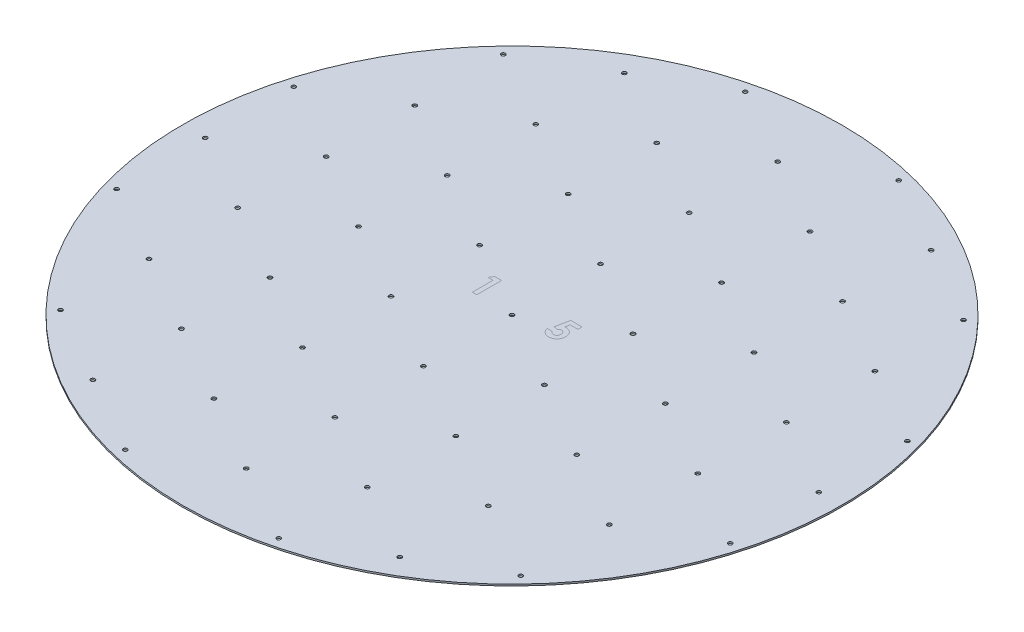
SolidWorks part; units mm, degrees
ref_plane "Front Plane" through (0, 0, 0) normal (0, 0, 1) x (1, 0, 0)
ref_plane "Top Plane" through (0, 0, 0) normal (0, 1, 0) x (1, 0, 0)
ref_plane "Right Plane" through (0, 0, 0) normal (1, 0, 0) x (0, 0, -1)
sketch "Sketch2" plane through (0, 0, 0) normal (0, 1, 0) x (1, 0, 0)
  circle A0 centre (0, 0) radius 40
  dimension "D1" = 80
extrude "Boss-Extrude1" add sketch "Sketch2" along normal blind 0.2
sketch "formula" plane through (0, 0.2, 0) normal (0, 1, 0) x (1, 0, 0)
  line L0 (0, 0) -> (0, 10.75) construction
  line L2 (46.374, 0) -> (0, 0) construction
  line L3 (9.3098, 5.375) -> (0, 0) construction
  line L4 (9.3098, 5.375) -> (0, 10.75) construction
  circle A16 centre (0, 10.75) radius 0.25
  circle A51 centre (9.3098, 16.125) radius 0.25
  circle A52 centre (0, 21.5) radius 0.25
  circle A53 centre (9.3098, 26.875) radius 0.25
  circle A54 centre (0, 32.25) radius 0.25
  circle A55 centre (9.3098, 37.625) radius 0.25
  circle A66 centre (0, 0) radius 0.25
  circle A67 centre (9.3098, 5.375) radius 0.25
  dimension "D2" = 0.5
  dimension "D3" = 10.75
sketch "Sketch4" plane through (0, 0.2, 0) normal (0, 1, 0) x (1, 0, 0)
  circle A1 centre (37.24, -10.75) radius 0.075
  circle A3 centre (18.62, -32.25) radius 0.075
  circle A5 centre (18.62, -10.75) radius 0.075
  circle A7 centre (27.9298, -16.125) radius 0.075
  circle A9 centre (18.62, -21.5) radius 0.075
  circle A11 centre (27.9298, -26.875) radius 0.075
  circle A13 centre (9.3098, -37.625) radius 0.075
  circle A15 centre (9.3098, -16.125) radius 0.075
  circle A17 centre (9.3098, -26.875) radius 0.075
  circle A19 centre (9.3098, -5.375) radius 0.075
  circle A21 centre (27.9298, -5.375) radius 0.075
  circle A23 centre (37.24, -10.75) radius 0.075
  circle A25 centre (18.62, -32.25) radius 0.075
  circle A27 centre (18.62, -10.75) radius 0.075
  circle A29 centre (27.9298, -16.125) radius 0.075
  circle A31 centre (18.62, -21.5) radius 0.075
  circle A33 centre (27.9298, -26.875) radius 0.075
  circle A35 centre (0, -32.25) radius 0.075
  circle A37 centre (9.3098, -37.625) radius 0.075
  circle A39 centre (0, -10.75) radius 0.075
  circle A41 centre (9.3098, -16.125) radius 0.075
  circle A43 centre (0, -21.5) radius 0.075
  circle A45 centre (9.3098, -26.875) radius 0.075
  circle A47 centre (9.3098, -5.375) radius 0.075
  circle A49 centre (27.9298, -5.375) radius 0.075
  circle A51 centre (-37.24, 10.75) radius 0.075
  circle A53 centre (-18.62, 32.25) radius 0.075
  circle A55 centre (-18.62, 10.75) radius 0.075
  circle A57 centre (-27.9298, 16.125) radius 0.075
  circle A59 centre (-18.62, 21.5) radius 0.075
  circle A61 centre (-27.9298, 26.875) radius 0.075
  circle A63 centre (-9.3098, 37.625) radius 0.075
  circle A65 centre (-9.3098, 16.125) radius 0.075
  circle A67 centre (-9.3098, 26.875) radius 0.075
  circle A69 centre (-9.3098, 5.375) radius 0.075
  circle A71 centre (-27.9298, 5.375) radius 0.075
  circle A73 centre (-37.24, 10.75) radius 0.075
  circle A75 centre (-37.24, 0) radius 0.075
  circle A77 centre (-18.62, 32.25) radius 0.075
  circle A79 centre (-18.62, 10.75) radius 0.075
  circle A81 centre (-27.9298, 16.125) radius 0.075
  circle A83 centre (-18.62, 21.5) radius 0.075
  circle A85 centre (-27.9298, 26.875) radius 0.075
  circle A87 centre (-18.62, 0) radius 0.075
  circle A89 centre (-9.3098, 37.625) radius 0.075
  circle A91 centre (-9.3098, 16.125) radius 0.075
  circle A93 centre (-9.3098, 26.875) radius 0.075
  circle A95 centre (-9.3098, 5.375) radius 0.075
  circle A97 centre (-27.9298, 5.375) radius 0.075
  circle A99 centre (-27.9298, -5.375) radius 0.075
  circle A101 centre (-9.3098, -5.375) radius 0.075
  circle A103 centre (-9.3098, -26.875) radius 0.075
  circle A105 centre (-9.3098, -16.125) radius 0.075
  circle A107 centre (-9.3098, -37.625) radius 0.075
  circle A109 centre (-27.9298, -26.875) radius 0.075
  circle A111 centre (-18.62, -21.5) radius 0.075
  circle A113 centre (-27.9298, -16.125) radius 0.075
  circle A115 centre (-18.62, -10.75) radius 0.075
  circle A117 centre (-18.62, -32.25) radius 0.075
  circle A119 centre (-37.24, -10.75) radius 0.075
  circle A121 centre (-27.9298, -5.375) radius 0.075
  circle A123 centre (-9.3098, -5.375) radius 0.075
  circle A125 centre (-9.3098, -26.875) radius 0.075
  circle A127 centre (-9.3098, -16.125) radius 0.075
  circle A129 centre (-9.3098, -37.625) radius 0.075
  circle A131 centre (-27.9298, -26.875) radius 0.075
  circle A133 centre (-18.62, -21.5) radius 0.075
  circle A135 centre (-27.9298, -16.125) radius 0.075
  circle A137 centre (-18.62, -10.75) radius 0.075
  circle A139 centre (-18.62, -32.25) radius 0.075
  circle A141 centre (-37.24, -10.75) radius 0.075
  circle A3000 centre (27.9298, 5.375) radius 0.25
  circle A3219 centre (9.3098, 5.375) radius 0.25
  circle A3220 centre (9.3098, 5.375) radius 0.25
  circle A3221 centre (0, 0) radius 0.25
  circle A3222 centre (0, 0) radius 0.25
  circle A3223 centre (9.3098, 26.875) radius 0.25
  circle A3224 centre (9.3098, 26.875) radius 0.25
  circle A3225 centre (0, 21.5) radius 0.25
  circle A3226 centre (0, 21.5) radius 0.25
  circle A3227 centre (9.3098, 16.125) radius 0.25
  circle A3228 centre (9.3098, 16.125) radius 0.25
  circle A3229 centre (0, 10.75) radius 0.25
  circle A3230 centre (0, 10.75) radius 0.25
  circle A3231 centre (9.3098, 37.625) radius 0.25
  circle A3232 centre (9.3098, 37.625) radius 0.25
  circle A3233 centre (0, 32.25) radius 0.25
  circle A3234 centre (0, 32.25) radius 0.25
  circle A3235 centre (18.62, 0) radius 0.25
  circle A3236 centre (27.9298, 26.875) radius 0.25
  circle A3237 centre (18.62, 21.5) radius 0.25
  circle A3238 centre (27.9298, 16.125) radius 0.25
  circle A3239 centre (18.62, 10.75) radius 0.25
  circle A3241 centre (18.62, 32.25) radius 0.25
  circle A3243 centre (37.24, 0) radius 0.25
  circle A3247 centre (37.24, 10.75) radius 0.25
  circle A3250 centre (27.9298, 37.625) radius 0.25
  circle A3251 centre (46.5498, 37.625) radius 0.25
  circle A3252 centre (37.24, 32.25) radius 0.25
  circle A3253 centre (46.5498, 26.875) radius 0.25
  circle A3254 centre (37.24, 21.5) radius 0.25
  circle A3255 centre (46.5498, 5.375) radius 0.25
  circle A3256 centre (46.5498, 16.125) radius 0.25
  circle A3271 centre (27.9298, 5.375) radius 0.075
  circle A3272 centre (9.3098, 5.375) radius 0.075
  circle A3273 centre (9.3098, 26.875) radius 0.075
  circle A3274 centre (9.3098, 16.125) radius 0.075
  circle A3275 centre (9.3098, 37.625) radius 0.075
  circle A3276 centre (27.9298, 26.875) radius 0.075
  circle A3277 centre (18.62, 21.5) radius 0.075
  circle A3278 centre (27.9298, 16.125) radius 0.075
  circle A3279 centre (18.62, 10.75) radius 0.075
  circle A3280 centre (18.62, 32.25) radius 0.075
  circle A3281 centre (37.24, 10.75) radius 0.075
  dimension "D121" = 0
  dimension "D122" = 0
  dimension "D123" = 0
  dimension "D124" = 0
  dimension "D125" = 0
  dimension "D126" = 0
  dimension "D127" = 0
  dimension "D128" = 0
  dimension "D129" = 3
extrude "Cut-Extrude2" cut sketch "Sketch4" against normal blind 0.2 contours A3222 | A3220 region at (0, 0.2, 0)
pattern_linear "LPattern1" count 4 spacing 10.75 along (0, 0, -1) count 3 spacing 18.6195 along (1, 0, 0) of "Cut-Extrude2"
mirror "Mirror1" about plane through (0, 0, 0) normal (1, 0, 0) of "LPattern1"
ref_plane "Plane1" through (0, 0, 0) normal (0, 0, -1) x (-1, 0, 0)
mirror "Mirror2" about plane through (0, 0, 0) normal (0, 0, -1) of "Mirror1", "LPattern1"
sketch "numbers" plane through (0, 0.2, 0) normal (0, 1, 0) x (1, 0, 0)
  line L0 (-7.0476, 0) -> (7.0476, 0) construction
  line L1 (46.374, 0) -> (0, 0) construction
  text T0 "<b>1      5</b>" font "Century Gothic" height 3
  point P6 (0, 0)
split "Split1" trim tools "numbers" bodies to split 160 resulting bodies 162 163 164
sketch "Sketch5" plane through (0, 0.2, 0) normal (0, 1, 0) x (1, 0, 0)
  circle A1 centre (40.7032, 13.5) radius 0.075
  circle A2 centre (40.7032, 13.5) radius 0.075
  circle A3 centre (39.8372, 15) radius 0.075
  circle A4 centre (39.8372, 15) radius 0.075
  circle A5 centre (39.8372, 14) radius 0.075
  circle A6 centre (39.8372, 14) radius 0.075
  circle A7 centre (40.7032, 14.5) radius 0.075
  circle A8 centre (40.7032, 14.5) radius 0.075
  circle A9 centre (39.8372, 10) radius 0.075
  circle A10 centre (39.8372, 10) radius 0.075
  circle A11 centre (39.8372, 11) radius 0.075
  circle A12 centre (39.8372, 11) radius 0.075
  circle A13 centre (39.8372, 10) radius 0.075
  circle A14 centre (39.8372, 10) radius 0.075
  circle A15 centre (40.7032, 10.5) radius 0.075
  circle A16 centre (40.7032, 10.5) radius 0.075
  circle A17 centre (38.9711, 8.5) radius 0.075
  circle A18 centre (38.9711, 8.5) radius 0.075
  circle A19 centre (38.1051, 9) radius 0.075
  circle A20 centre (38.1051, 9) radius 0.075
  circle A21 centre (38.9711, 9.5) radius 0.075
  circle A22 centre (38.9711, 9.5) radius 0.075
  circle A23 centre (38.1051, 5) radius 0.075
  circle A24 centre (38.1051, 5) radius 0.075
  circle A25 centre (38.1051, 6) radius 0.075
  circle A26 centre (38.1051, 6) radius 0.075
  circle A27 centre (38.1051, 5) radius 0.075
  circle A28 centre (38.1051, 5) radius 0.075
  circle A29 centre (38.9711, 5.5) radius 0.075
  circle A30 centre (38.9711, 5.5) radius 0.075
  circle A31 centre (38.1051, 7) radius 0.075
  circle A32 centre (38.1051, 7) radius 0.075
  circle A33 centre (36.3731, 4) radius 0.075
  circle A34 centre (36.3731, 4) radius 0.075
  circle A35 centre (37.2391, 4.5) radius 0.075
  circle A36 centre (37.2391, 4.5) radius 0.075
  circle A37 centre (36.3731, 0) radius 0.075
  circle A38 centre (36.3731, 0) radius 0.075
  circle A39 centre (37.2391, 0.5) radius 0.075
  circle A40 centre (37.2391, 0.5) radius 0.075
  circle A41 centre (36.3731, 1) radius 0.075
  circle A42 centre (36.3731, 1) radius 0.075
  circle A43 centre (36.3731, 2) radius 0.075
  circle A44 centre (36.3731, 2) radius 0.075
  circle A45 centre (36.3731, 1) radius 0.075
  circle A46 centre (36.3731, 1) radius 0.075
  circle A47 centre (37.2391, 1.5) radius 0.075
  circle A48 centre (37.2391, 1.5) radius 0.075
  circle A71 centre (31.1769, 29) radius 0.075
  circle A72 centre (31.1769, 29) radius 0.075
  circle A73 centre (32.0429, 28.5) radius 0.075
  circle A74 centre (32.0429, 28.5) radius 0.075
  circle A75 centre (31.1769, 30) radius 0.075
  circle A76 centre (31.1769, 30) radius 0.075
  circle A77 centre (31.1769, 29) radius 0.075
  circle A78 centre (31.1769, 29) radius 0.075
  circle A79 centre (32.0429, 29.5) radius 0.075
  circle A80 centre (32.0429, 29.5) radius 0.075
  circle A81 centre (30.3109, 27.5) radius 0.075
  circle A82 centre (30.3109, 27.5) radius 0.075
  circle A83 centre (29.4449, 28) radius 0.075
  circle A84 centre (29.4449, 28) radius 0.075
  circle A85 centre (29.4449, 24) radius 0.075
  circle A86 centre (29.4449, 24) radius 0.075
  circle A87 centre (29.4449, 23) radius 0.075
  circle A88 centre (29.4449, 23) radius 0.075
  circle A89 centre (30.3109, 23.5) radius 0.075
  circle A90 centre (30.3109, 23.5) radius 0.075
  circle A91 centre (29.4449, 25) radius 0.075
  circle A92 centre (29.4449, 25) radius 0.075
  circle A93 centre (29.4449, 24) radius 0.075
  circle A94 centre (29.4449, 24) radius 0.075
  circle A95 centre (30.3109, 24.5) radius 0.075
  circle A96 centre (30.3109, 24.5) radius 0.075
  circle A97 centre (27.7128, 23) radius 0.075
  circle A98 centre (27.7128, 23) radius 0.075
  circle A99 centre (27.7128, 22) radius 0.075
  circle A100 centre (27.7128, 22) radius 0.075
  circle A101 centre (28.5788, 22.5) radius 0.075
  circle A102 centre (28.5788, 22.5) radius 0.075
  circle A103 centre (27.7128, 19) radius 0.075
  circle A104 centre (27.7128, 19) radius 0.075
  circle A105 centre (27.7128, 18) radius 0.075
  circle A106 centre (27.7128, 18) radius 0.075
  circle A107 centre (28.5788, 18.5) radius 0.075
  circle A108 centre (28.5788, 18.5) radius 0.075
  circle A109 centre (27.7128, 20) radius 0.075
  circle A110 centre (27.7128, 20) radius 0.075
  circle A111 centre (27.7128, 19) radius 0.075
  circle A112 centre (27.7128, 19) radius 0.075
  circle A113 centre (25.9808, 17) radius 0.075
  circle A114 centre (25.9808, 17) radius 0.075
  circle A115 centre (25.9808, 16) radius 0.075
  circle A116 centre (25.9808, 16) radius 0.075
  circle A117 centre (26.8468, 16.5) radius 0.075
  circle A118 centre (26.8468, 16.5) radius 0.075
  circle A119 centre (25.9808, 13) radius 0.075
  circle A120 centre (25.9808, 13) radius 0.075
  circle A121 centre (25.9808, 12) radius 0.075
  circle A122 centre (25.9808, 12) radius 0.075
  circle A123 centre (26.8468, 12.5) radius 0.075
  circle A124 centre (26.8468, 12.5) radius 0.075
  circle A125 centre (25.9808, 14) radius 0.075
  circle A126 centre (25.9808, 14) radius 0.075
  circle A127 centre (25.9808, 13) radius 0.075
  circle A128 centre (25.9808, 13) radius 0.075
  circle A129 centre (24.2487, 12) radius 0.075
  circle A130 centre (24.2487, 12) radius 0.075
  circle A131 centre (24.2487, 11) radius 0.075
  circle A132 centre (24.2487, 11) radius 0.075
  circle A133 centre (25.1147, 11.5) radius 0.075
  circle A134 centre (25.1147, 11.5) radius 0.075
  circle A135 centre (24.2487, 8) radius 0.075
  circle A136 centre (24.2487, 8) radius 0.075
  circle A137 centre (24.2487, 7) radius 0.075
  circle A138 centre (24.2487, 7) radius 0.075
  circle A139 centre (25.1147, 7.5) radius 0.075
  circle A140 centre (25.1147, 7.5) radius 0.075
  circle A141 centre (24.2487, 9) radius 0.075
  circle A142 centre (24.2487, 9) radius 0.075
  circle A143 centre (24.2487, 8) radius 0.075
  circle A144 centre (24.2487, 8) radius 0.075
  circle A145 centre (22.5167, 6) radius 0.075
  circle A146 centre (22.5167, 6) radius 0.075
  circle A147 centre (23.3827, 6.5) radius 0.075
  circle A148 centre (23.3827, 6.5) radius 0.075
  circle A149 centre (22.5167, 3) radius 0.075
  circle A150 centre (22.5167, 3) radius 0.075
  circle A151 centre (22.5167, 2) radius 0.075
  circle A152 centre (22.5167, 2) radius 0.075
  circle A153 centre (23.3827, 2.5) radius 0.075
  circle A154 centre (23.3827, 2.5) radius 0.075
  circle A155 centre (22.5167, 4) radius 0.075
  circle A156 centre (22.5167, 4) radius 0.075
  circle A157 centre (22.5167, 3) radius 0.075
  circle A158 centre (22.5167, 3) radius 0.075
  circle A159 centre (23.3827, 3.5) radius 0.075
  circle A160 centre (23.3827, 3.5) radius 0.075
  circle A177 centre (18.1865, 35.5) radius 0.075
  circle A178 centre (18.1865, 35.5) radius 0.075
  circle A179 centre (17.3205, 36) radius 0.075
  circle A180 centre (17.3205, 36) radius 0.075
  circle A181 centre (17.3205, 32) radius 0.075
  circle A182 centre (17.3205, 32) radius 0.075
  circle A183 centre (17.3205, 31) radius 0.075
  circle A184 centre (17.3205, 31) radius 0.075
  circle A185 centre (18.1865, 31.5) radius 0.075
  circle A186 centre (18.1865, 31.5) radius 0.075
  circle A187 centre (17.3205, 33) radius 0.075
  circle A188 centre (17.3205, 33) radius 0.075
  circle A189 centre (17.3205, 32) radius 0.075
  circle A190 centre (17.3205, 32) radius 0.075
  circle A191 centre (18.1865, 32.5) radius 0.075
  circle A192 centre (18.1865, 32.5) radius 0.075
  circle A193 centre (15.5885, 31) radius 0.075
  circle A194 centre (15.5885, 31) radius 0.075
  circle A195 centre (15.5885, 30) radius 0.075
  circle A196 centre (15.5885, 30) radius 0.075
  circle A197 centre (16.4545, 30.5) radius 0.075
  circle A198 centre (16.4545, 30.5) radius 0.075
  circle A199 centre (15.5885, 27) radius 0.075
  circle A200 centre (15.5885, 27) radius 0.075
  circle A201 centre (15.5885, 26) radius 0.075
  circle A202 centre (15.5885, 26) radius 0.075
  circle A203 centre (16.4545, 26.5) radius 0.075
  circle A204 centre (16.4545, 26.5) radius 0.075
  circle A205 centre (15.5885, 28) radius 0.075
  circle A206 centre (15.5885, 28) radius 0.075
  circle A207 centre (15.5885, 27) radius 0.075
  circle A208 centre (15.5885, 27) radius 0.075
  circle A209 centre (13.8564, 26) radius 0.075
  circle A210 centre (13.8564, 26) radius 0.075
  circle A211 centre (13.8564, 25) radius 0.075
  circle A212 centre (13.8564, 25) radius 0.075
  circle A213 centre (14.7224, 25.5) radius 0.075
  circle A214 centre (14.7224, 25.5) radius 0.075
  circle A215 centre (13.8564, 21) radius 0.075
  circle A216 centre (13.8564, 21) radius 0.075
  circle A217 centre (14.7224, 20.5) radius 0.075
  circle A218 centre (14.7224, 20.5) radius 0.075
  circle A219 centre (13.8564, 22) radius 0.075
  circle A220 centre (13.8564, 22) radius 0.075
  circle A221 centre (13.8564, 21) radius 0.075
  circle A222 centre (13.8564, 21) radius 0.075
  circle A223 centre (14.7224, 21.5) radius 0.075
  circle A224 centre (14.7224, 21.5) radius 0.075
  circle A225 centre (12.9904, 19.5) radius 0.075
  circle A226 centre (12.9904, 19.5) radius 0.075
  circle A227 centre (12.1244, 20) radius 0.075
  circle A228 centre (12.1244, 20) radius 0.075
  circle A229 centre (12.1244, 18) radius 0.075
  circle A230 centre (12.1244, 18) radius 0.075
  circle A231 centre (12.1244, 17) radius 0.075
  circle A232 centre (12.1244, 17) radius 0.075
  circle A233 centre (12.9904, 17.5) radius 0.075
  circle A234 centre (12.9904, 17.5) radius 0.075
  circle A235 centre (12.1244, 16) radius 0.075
  circle A236 centre (12.1244, 16) radius 0.075
  circle A237 centre (12.1244, 15) radius 0.075
  circle A238 centre (12.1244, 15) radius 0.075
  circle A239 centre (12.9904, 15.5) radius 0.075
  circle A240 centre (12.9904, 15.5) radius 0.075
  circle A241 centre (11.2583, 13.5) radius 0.075
  circle A242 centre (11.2583, 13.5) radius 0.075
  circle A243 centre (10.3923, 15) radius 0.075
  circle A244 centre (10.3923, 15) radius 0.075
  circle A245 centre (10.3923, 14) radius 0.075
  circle A246 centre (10.3923, 14) radius 0.075
  circle A247 centre (11.2583, 14.5) radius 0.075
  circle A248 centre (11.2583, 14.5) radius 0.075
  circle A249 centre (10.3923, 10) radius 0.075
  circle A250 centre (10.3923, 10) radius 0.075
  circle A251 centre (10.3923, 11) radius 0.075
  circle A252 centre (10.3923, 11) radius 0.075
  circle A253 centre (10.3923, 10) radius 0.075
  circle A254 centre (10.3923, 10) radius 0.075
  circle A255 centre (11.2583, 10.5) radius 0.075
  circle A256 centre (11.2583, 10.5) radius 0.075
  circle A257 centre (9.5263, 8.5) radius 0.075
  circle A258 centre (9.5263, 8.5) radius 0.075
  circle A259 centre (8.6603, 9) radius 0.075
  circle A260 centre (8.6603, 9) radius 0.075
  circle A261 centre (9.5263, 9.5) radius 0.075
  circle A262 centre (9.5263, 9.5) radius 0.075
  circle A263 centre (8.6603, 5) radius 0.075
  circle A264 centre (8.6603, 5) radius 0.075
  circle A265 centre (8.6603, 6) radius 0.075
  circle A266 centre (8.6603, 6) radius 0.075
  circle A267 centre (8.6603, 5) radius 0.075
  circle A268 centre (8.6603, 5) radius 0.075
  circle A269 centre (9.5263, 5.5) radius 0.075
  circle A270 centre (9.5263, 5.5) radius 0.075
  circle A271 centre (8.6603, 7) radius 0.075
  circle A272 centre (8.6603, 7) radius 0.075
  circle A273 centre (6.9282, 4) radius 0.075
  circle A274 centre (6.9282, 4) radius 0.075
  circle A275 centre (7.7942, 4.5) radius 0.075
  circle A276 centre (7.7942, 4.5) radius 0.075
  circle A277 centre (6.9282, 0) radius 0.075
  circle A278 centre (6.9282, 0) radius 0.075
  circle A279 centre (7.7942, 0.5) radius 0.075
  circle A280 centre (7.7942, 0.5) radius 0.075
  circle A281 centre (6.9282, 1) radius 0.075
  circle A282 centre (6.9282, 1) radius 0.075
  circle A283 centre (6.9282, 2) radius 0.075
  circle A284 centre (6.9282, 2) radius 0.075
  circle A285 centre (6.9282, 1) radius 0.075
  circle A286 centre (6.9282, 1) radius 0.075
  circle A287 centre (7.7942, 1.5) radius 0.075
  circle A288 centre (7.7942, 1.5) radius 0.075
  circle A289 centre (3.4641, 39) radius 0.075
  circle A290 centre (3.4641, 39) radius 0.075
  circle A291 centre (3.4641, 38) radius 0.075
  circle A292 centre (3.4641, 38) radius 0.075
  circle A293 centre (4.3301, 38.5) radius 0.075
  circle A294 centre (4.3301, 38.5) radius 0.075
  circle A295 centre (3.4641, 35) radius 0.075
  circle A296 centre (3.4641, 35) radius 0.075
  circle A297 centre (3.4641, 34) radius 0.075
  circle A298 centre (3.4641, 34) radius 0.075
  circle A299 centre (4.3301, 34.5) radius 0.075
  circle A300 centre (4.3301, 34.5) radius 0.075
  circle A301 centre (3.4641, 36) radius 0.075
  circle A302 centre (3.4641, 36) radius 0.075
  circle A303 centre (3.4641, 35) radius 0.075
  circle A304 centre (3.4641, 35) radius 0.075
  circle A305 centre (1.7321, 34) radius 0.075
  circle A306 centre (1.7321, 34) radius 0.075
  circle A307 centre (1.7321, 33) radius 0.075
  circle A308 centre (1.7321, 33) radius 0.075
  circle A309 centre (2.5981, 33.5) radius 0.075
  circle A310 centre (2.5981, 33.5) radius 0.075
  circle A311 centre (1.7321, 29) radius 0.075
  circle A312 centre (1.7321, 29) radius 0.075
  circle A313 centre (2.5981, 28.5) radius 0.075
  circle A314 centre (2.5981, 28.5) radius 0.075
  circle A315 centre (1.7321, 30) radius 0.075
  circle A316 centre (1.7321, 30) radius 0.075
  circle A317 centre (1.7321, 29) radius 0.075
  circle A318 centre (1.7321, 29) radius 0.075
  circle A319 centre (2.5981, 29.5) radius 0.075
  circle A320 centre (2.5981, 29.5) radius 0.075
  circle A321 centre (0.866, 28.5) radius 0.075
  circle A322 centre (0.866, 28.5) radius 0.075
  circle A323 centre (0, 30) radius 0.075
  circle A324 centre (0, 30) radius 0.075
  circle A325 centre (0, 29) radius 0.075
  circle A326 centre (0, 29) radius 0.075
  circle A327 centre (0.866, 29.5) radius 0.075
  circle A328 centre (0.866, 29.5) radius 0.075
  circle A329 centre (0, 31) radius 0.075
  circle A330 centre (0, 31) radius 0.075
  circle A331 centre (0.866, 1.5) radius 0.075
  circle A332 centre (0.866, 1.5) radius 0.075
  circle A335 centre (0, 39) radius 0.075
  circle A336 centre (0, 39) radius 0.075
  circle A337 centre (0.866, 39.5) radius 0.075
  circle A338 centre (0.866, 39.5) radius 0.075
  circle A339 centre (39.8372, 17) radius 0.075
  circle A340 centre (39.8372, 17) radius 0.075
  circle A341 centre (39.8372, 16) radius 0.075
  circle A342 centre (39.8372, 16) radius 0.075
  circle A343 centre (40.7032, 16.5) radius 0.075
  circle A344 centre (40.7032, 16.5) radius 0.075
  circle A345 centre (39.8372, 13) radius 0.075
  circle A346 centre (39.8372, 13) radius 0.075
  circle A347 centre (39.8372, 12) radius 0.075
  circle A348 centre (39.8372, 12) radius 0.075
  circle A349 centre (40.7032, 12.5) radius 0.075
  circle A350 centre (40.7032, 12.5) radius 0.075
  circle A351 centre (39.8372, 14) radius 0.075
  circle A352 centre (39.8372, 14) radius 0.075
  circle A353 centre (39.8372, 13) radius 0.075
  circle A354 centre (39.8372, 13) radius 0.075
  circle A355 centre (38.1051, 12) radius 0.075
  circle A356 centre (38.1051, 12) radius 0.075
  circle A357 centre (38.1051, 11) radius 0.075
  circle A358 centre (38.1051, 11) radius 0.075
  circle A359 centre (38.9711, 11.5) radius 0.075
  circle A360 centre (38.9711, 11.5) radius 0.075
  circle A361 centre (38.1051, 8) radius 0.075
  circle A362 centre (38.1051, 8) radius 0.075
  circle A363 centre (38.1051, 7) radius 0.075
  circle A364 centre (38.1051, 7) radius 0.075
  circle A365 centre (38.9711, 7.5) radius 0.075
  circle A366 centre (38.9711, 7.5) radius 0.075
  circle A367 centre (38.1051, 9) radius 0.075
  circle A368 centre (38.1051, 9) radius 0.075
  circle A369 centre (38.1051, 8) radius 0.075
  circle A370 centre (38.1051, 8) radius 0.075
  circle A371 centre (36.3731, 6) radius 0.075
  circle A372 centre (36.3731, 6) radius 0.075
  circle A373 centre (37.2391, 6.5) radius 0.075
  circle A374 centre (37.2391, 6.5) radius 0.075
  circle A375 centre (36.3731, 3) radius 0.075
  circle A376 centre (36.3731, 3) radius 0.075
  circle A377 centre (36.3731, 2) radius 0.075
  circle A378 centre (36.3731, 2) radius 0.075
  circle A379 centre (37.2391, 2.5) radius 0.075
  circle A380 centre (37.2391, 2.5) radius 0.075
  circle A381 centre (36.3731, 4) radius 0.075
  circle A382 centre (36.3731, 4) radius 0.075
  circle A383 centre (36.3731, 3) radius 0.075
  circle A384 centre (36.3731, 3) radius 0.075
  circle A385 centre (37.2391, 3.5) radius 0.075
  circle A386 centre (37.2391, 3.5) radius 0.075
  circle A407 centre (31.1769, 32) radius 0.075
  circle A408 centre (31.1769, 32) radius 0.075
  circle A409 centre (31.1769, 31) radius 0.075
  circle A410 centre (31.1769, 31) radius 0.075
  circle A411 centre (32.0429, 31.5) radius 0.075
  circle A412 centre (32.0429, 31.5) radius 0.075
  circle A415 centre (31.1769, 32) radius 0.075
  circle A416 centre (31.1769, 32) radius 0.075
  circle A417 centre (32.0429, 32.5) radius 0.075
  circle A418 centre (32.0429, 32.5) radius 0.075
  circle A419 centre (29.4449, 31) radius 0.075
  circle A420 centre (29.4449, 31) radius 0.075
  circle A421 centre (29.4449, 30) radius 0.075
  circle A422 centre (29.4449, 30) radius 0.075
  circle A423 centre (30.3109, 30.5) radius 0.075
  circle A424 centre (30.3109, 30.5) radius 0.075
  circle A425 centre (29.4449, 27) radius 0.075
  circle A426 centre (29.4449, 27) radius 0.075
  circle A427 centre (29.4449, 26) radius 0.075
  circle A428 centre (29.4449, 26) radius 0.075
  circle A429 centre (30.3109, 26.5) radius 0.075
  circle A430 centre (30.3109, 26.5) radius 0.075
  circle A431 centre (29.4449, 28) radius 0.075
  circle A432 centre (29.4449, 28) radius 0.075
  circle A433 centre (29.4449, 27) radius 0.075
  circle A434 centre (29.4449, 27) radius 0.075
  circle A435 centre (27.7128, 26) radius 0.075
  circle A436 centre (27.7128, 26) radius 0.075
  circle A437 centre (27.7128, 25) radius 0.075
  circle A438 centre (27.7128, 25) radius 0.075
  circle A439 centre (28.5788, 25.5) radius 0.075
  circle A440 centre (28.5788, 25.5) radius 0.075
  circle A441 centre (27.7128, 21) radius 0.075
  circle A442 centre (27.7128, 21) radius 0.075
  circle A443 centre (28.5788, 20.5) radius 0.075
  circle A444 centre (28.5788, 20.5) radius 0.075
  circle A445 centre (27.7128, 22) radius 0.075
  circle A446 centre (27.7128, 22) radius 0.075
  circle A447 centre (27.7128, 21) radius 0.075
  circle A448 centre (27.7128, 21) radius 0.075
  circle A449 centre (28.5788, 21.5) radius 0.075
  circle A450 centre (28.5788, 21.5) radius 0.075
  circle A451 centre (26.8468, 19.5) radius 0.075
  circle A452 centre (26.8468, 19.5) radius 0.075
  circle A453 centre (25.9808, 20) radius 0.075
  circle A454 centre (25.9808, 20) radius 0.075
  circle A455 centre (25.9808, 18) radius 0.075
  circle A456 centre (25.9808, 18) radius 0.075
  circle A457 centre (25.9808, 17) radius 0.075
  circle A458 centre (25.9808, 17) radius 0.075
  circle A459 centre (26.8468, 17.5) radius 0.075
  circle A460 centre (26.8468, 17.5) radius 0.075
  circle A461 centre (25.9808, 16) radius 0.075
  circle A462 centre (25.9808, 16) radius 0.075
  circle A463 centre (25.9808, 15) radius 0.075
  circle A464 centre (25.9808, 15) radius 0.075
  circle A465 centre (26.8468, 15.5) radius 0.075
  circle A466 centre (26.8468, 15.5) radius 0.075
  circle A467 centre (25.1147, 13.5) radius 0.075
  circle A468 centre (25.1147, 13.5) radius 0.075
  circle A469 centre (24.2487, 15) radius 0.075
  circle A470 centre (24.2487, 15) radius 0.075
  circle A471 centre (24.2487, 14) radius 0.075
  circle A472 centre (24.2487, 14) radius 0.075
  circle A473 centre (25.1147, 14.5) radius 0.075
  circle A474 centre (25.1147, 14.5) radius 0.075
  circle A475 centre (24.2487, 10) radius 0.075
  circle A476 centre (24.2487, 10) radius 0.075
  circle A477 centre (24.2487, 11) radius 0.075
  circle A478 centre (24.2487, 11) radius 0.075
  circle A479 centre (24.2487, 10) radius 0.075
  circle A480 centre (24.2487, 10) radius 0.075
  circle A481 centre (25.1147, 10.5) radius 0.075
  circle A482 centre (25.1147, 10.5) radius 0.075
  circle A483 centre (23.3827, 8.5) radius 0.075
  circle A484 centre (23.3827, 8.5) radius 0.075
  circle A485 centre (22.5167, 9) radius 0.075
  circle A486 centre (22.5167, 9) radius 0.075
  circle A487 centre (23.3827, 9.5) radius 0.075
  circle A488 centre (23.3827, 9.5) radius 0.075
  circle A489 centre (22.5167, 5) radius 0.075
  circle A490 centre (22.5167, 5) radius 0.075
  circle A491 centre (22.5167, 6) radius 0.075
  circle A492 centre (22.5167, 6) radius 0.075
  circle A493 centre (22.5167, 5) radius 0.075
  circle A494 centre (22.5167, 5) radius 0.075
  circle A495 centre (23.3827, 5.5) radius 0.075
  circle A496 centre (23.3827, 5.5) radius 0.075
  circle A497 centre (22.5167, 7) radius 0.075
  circle A498 centre (22.5167, 7) radius 0.075
  circle A499 centre (20.7846, 4) radius 0.075
  circle A500 centre (20.7846, 4) radius 0.075
  circle A501 centre (21.6506, 4.5) radius 0.075
  circle A502 centre (21.6506, 4.5) radius 0.075
  circle A503 centre (20.7846, 0) radius 0.075
  circle A504 centre (20.7846, 0) radius 0.075
  circle A505 centre (21.6506, 0.5) radius 0.075
  circle A506 centre (21.6506, 0.5) radius 0.075
  circle A507 centre (20.7846, 1) radius 0.075
  circle A508 centre (20.7846, 1) radius 0.075
  circle A509 centre (20.7846, 2) radius 0.075
  circle A510 centre (20.7846, 2) radius 0.075
  circle A511 centre (20.7846, 1) radius 0.075
  circle A512 centre (20.7846, 1) radius 0.075
  circle A513 centre (21.6506, 1.5) radius 0.075
  circle A514 centre (21.6506, 1.5) radius 0.075
  circle A515 centre (17.3205, 39) radius 0.075
  circle A516 centre (17.3205, 39) radius 0.075
  circle A517 centre (17.3205, 38) radius 0.075
  circle A518 centre (17.3205, 38) radius 0.075
  circle A521 centre (17.3205, 35) radius 0.075
  circle A522 centre (17.3205, 35) radius 0.075
  circle A523 centre (17.3205, 34) radius 0.075
  circle A524 centre (17.3205, 34) radius 0.075
  circle A525 centre (18.1865, 34.5) radius 0.075
  circle A526 centre (18.1865, 34.5) radius 0.075
  circle A527 centre (17.3205, 36) radius 0.075
  circle A528 centre (17.3205, 36) radius 0.075
  circle A529 centre (17.3205, 35) radius 0.075
  circle A530 centre (17.3205, 35) radius 0.075
  circle A531 centre (15.5885, 34) radius 0.075
  circle A532 centre (15.5885, 34) radius 0.075
  circle A533 centre (15.5885, 33) radius 0.075
  circle A534 centre (15.5885, 33) radius 0.075
  circle A535 centre (16.4545, 33.5) radius 0.075
  circle A536 centre (16.4545, 33.5) radius 0.075
  circle A537 centre (15.5885, 29) radius 0.075
  circle A538 centre (15.5885, 29) radius 0.075
  circle A539 centre (16.4545, 28.5) radius 0.075
  circle A540 centre (16.4545, 28.5) radius 0.075
  circle A541 centre (15.5885, 30) radius 0.075
  circle A542 centre (15.5885, 30) radius 0.075
  circle A543 centre (15.5885, 29) radius 0.075
  circle A544 centre (15.5885, 29) radius 0.075
  circle A545 centre (16.4545, 29.5) radius 0.075
  circle A546 centre (16.4545, 29.5) radius 0.075
  circle A547 centre (14.7224, 27.5) radius 0.075
  circle A548 centre (14.7224, 27.5) radius 0.075
  circle A549 centre (13.8564, 28) radius 0.075
  circle A550 centre (13.8564, 28) radius 0.075
  circle A551 centre (13.8564, 24) radius 0.075
  circle A552 centre (13.8564, 24) radius 0.075
  circle A553 centre (13.8564, 23) radius 0.075
  circle A554 centre (13.8564, 23) radius 0.075
  circle A555 centre (14.7224, 23.5) radius 0.075
  circle A556 centre (14.7224, 23.5) radius 0.075
  circle A557 centre (13.8564, 25) radius 0.075
  circle A558 centre (13.8564, 25) radius 0.075
  circle A559 centre (13.8564, 24) radius 0.075
  circle A560 centre (13.8564, 24) radius 0.075
  circle A561 centre (14.7224, 24.5) radius 0.075
  circle A562 centre (14.7224, 24.5) radius 0.075
  circle A563 centre (12.1244, 23) radius 0.075
  circle A564 centre (12.1244, 23) radius 0.075
  circle A565 centre (12.1244, 22) radius 0.075
  circle A566 centre (12.1244, 22) radius 0.075
  circle A567 centre (12.9904, 22.5) radius 0.075
  circle A568 centre (12.9904, 22.5) radius 0.075
  circle A569 centre (12.1244, 19) radius 0.075
  circle A570 centre (12.1244, 19) radius 0.075
  circle A571 centre (12.1244, 18) radius 0.075
  circle A572 centre (12.1244, 18) radius 0.075
  circle A573 centre (12.9904, 18.5) radius 0.075
  circle A574 centre (12.9904, 18.5) radius 0.075
  circle A575 centre (12.1244, 20) radius 0.075
  circle A576 centre (12.1244, 20) radius 0.075
  circle A577 centre (12.1244, 19) radius 0.075
  circle A578 centre (12.1244, 19) radius 0.075
  circle A579 centre (10.3923, 17) radius 0.075
  circle A580 centre (10.3923, 17) radius 0.075
  circle A581 centre (10.3923, 16) radius 0.075
  circle A582 centre (10.3923, 16) radius 0.075
  circle A583 centre (11.2583, 16.5) radius 0.075
  circle A584 centre (11.2583, 16.5) radius 0.075
  circle A585 centre (10.3923, 13) radius 0.075
  circle A586 centre (10.3923, 13) radius 0.075
  circle A587 centre (10.3923, 12) radius 0.075
  circle A588 centre (10.3923, 12) radius 0.075
  circle A589 centre (11.2583, 12.5) radius 0.075
  circle A590 centre (11.2583, 12.5) radius 0.075
  circle A591 centre (10.3923, 14) radius 0.075
  circle A592 centre (10.3923, 14) radius 0.075
  circle A593 centre (10.3923, 13) radius 0.075
  circle A594 centre (10.3923, 13) radius 0.075
  circle A595 centre (8.6603, 12) radius 0.075
  circle A596 centre (8.6603, 12) radius 0.075
  circle A597 centre (8.6603, 11) radius 0.075
  circle A598 centre (8.6603, 11) radius 0.075
  circle A599 centre (9.5263, 11.5) radius 0.075
  circle A600 centre (9.5263, 11.5) radius 0.075
  circle A601 centre (8.6603, 8) radius 0.075
  circle A602 centre (8.6603, 8) radius 0.075
  circle A603 centre (8.6603, 7) radius 0.075
  circle A604 centre (8.6603, 7) radius 0.075
  circle A605 centre (9.5263, 7.5) radius 0.075
  circle A606 centre (9.5263, 7.5) radius 0.075
  circle A607 centre (8.6603, 9) radius 0.075
  circle A608 centre (8.6603, 9) radius 0.075
  circle A609 centre (8.6603, 8) radius 0.075
  circle A610 centre (8.6603, 8) radius 0.075
  circle A611 centre (6.9282, 6) radius 0.075
  circle A612 centre (6.9282, 6) radius 0.075
  circle A613 centre (7.7942, 6.5) radius 0.075
  circle A614 centre (7.7942, 6.5) radius 0.075
  circle A615 centre (6.9282, 3) radius 0.075
  circle A616 centre (6.9282, 3) radius 0.075
  circle A617 centre (6.9282, 2) radius 0.075
  circle A618 centre (6.9282, 2) radius 0.075
  circle A619 centre (7.7942, 2.5) radius 0.075
  circle A620 centre (7.7942, 2.5) radius 0.075
  circle A621 centre (6.9282, 4) radius 0.075
  circle A622 centre (6.9282, 4) radius 0.075
  circle A623 centre (6.9282, 3) radius 0.075
  circle A624 centre (6.9282, 3) radius 0.075
  circle A625 centre (7.7942, 3.5) radius 0.075
  circle A626 centre (7.7942, 3.5) radius 0.075
  circle A629 centre (5.1962, 39) radius 0.075
  circle A630 centre (5.1962, 39) radius 0.075
  circle A633 centre (3.4641, 37) radius 0.075
  circle A634 centre (3.4641, 37) radius 0.075
  circle A635 centre (4.3301, 36.5) radius 0.075
  circle A636 centre (4.3301, 36.5) radius 0.075
  circle A637 centre (3.4641, 38) radius 0.075
  circle A638 centre (3.4641, 38) radius 0.075
  circle A639 centre (3.4641, 37) radius 0.075
  circle A640 centre (3.4641, 37) radius 0.075
  circle A641 centre (4.3301, 37.5) radius 0.075
  circle A642 centre (4.3301, 37.5) radius 0.075
  circle A643 centre (2.5981, 35.5) radius 0.075
  circle A644 centre (2.5981, 35.5) radius 0.075
  circle A645 centre (1.7321, 36) radius 0.075
  circle A646 centre (1.7321, 36) radius 0.075
  circle A647 centre (1.7321, 32) radius 0.075
  circle A648 centre (1.7321, 32) radius 0.075
  circle A649 centre (1.7321, 31) radius 0.075
  circle A650 centre (1.7321, 31) radius 0.075
  circle A651 centre (2.5981, 31.5) radius 0.075
  circle A652 centre (2.5981, 31.5) radius 0.075
  circle A653 centre (1.7321, 33) radius 0.075
  circle A654 centre (1.7321, 33) radius 0.075
  circle A655 centre (1.7321, 32) radius 0.075
  circle A656 centre (1.7321, 32) radius 0.075
  circle A657 centre (2.5981, 32.5) radius 0.075
  circle A658 centre (2.5981, 32.5) radius 0.075
  circle A659 centre (0.866, 32.5) radius 0.075
  circle A660 centre (0.866, 32.5) radius 0.075
  circle A661 centre (0, 34) radius 0.075
  circle A662 centre (0, 34) radius 0.075
  circle A663 centre (0, 33) radius 0.075
  circle A664 centre (0, 33) radius 0.075
  circle A665 centre (0.866, 33.5) radius 0.075
  circle A666 centre (0.866, 33.5) radius 0.075
  circle A667 centre (0, 29) radius 0.075
  circle A668 centre (0, 29) radius 0.075
  circle A669 centre (0.866, 4.5) radius 0.075
  circle A670 centre (0.866, 4.5) radius 0.075
  circle A671 centre (0, 0) radius 0.075
  circle A672 centre (0, 0) radius 0.075
  circle A673 centre (0.866, 0.5) radius 0.075
  circle A674 centre (0.866, 0.5) radius 0.075
  circle A675 centre (0, 1) radius 0.075
  circle A676 centre (0, 1) radius 0.075
  circle A677 centre (0, 2) radius 0.075
  circle A678 centre (0, 2) radius 0.075
  circle A679 centre (0, 1) radius 0.075
  circle A680 centre (0, 1) radius 0.075
  circle A681 centre (40.7032, 19.5) radius 0.075
  circle A682 centre (40.7032, 19.5) radius 0.075
  circle A683 centre (39.8372, 20) radius 0.075
  circle A684 centre (39.8372, 20) radius 0.075
  circle A685 centre (39.8372, 18) radius 0.075
  circle A686 centre (39.8372, 18) radius 0.075
  circle A687 centre (39.8372, 17) radius 0.075
  circle A688 centre (39.8372, 17) radius 0.075
  circle A689 centre (40.7032, 17.5) radius 0.075
  circle A690 centre (40.7032, 17.5) radius 0.075
  circle A691 centre (39.8372, 16) radius 0.075
  circle A692 centre (39.8372, 16) radius 0.075
  circle A693 centre (39.8372, 15) radius 0.075
  circle A694 centre (39.8372, 15) radius 0.075
  circle A695 centre (40.7032, 15.5) radius 0.075
  circle A696 centre (40.7032, 15.5) radius 0.075
  circle A697 centre (38.9711, 13.5) radius 0.075
  circle A698 centre (38.9711, 13.5) radius 0.075
  circle A699 centre (38.1051, 15) radius 0.075
  circle A700 centre (38.1051, 15) radius 0.075
  circle A701 centre (38.1051, 14) radius 0.075
  circle A702 centre (38.1051, 14) radius 0.075
  circle A703 centre (38.9711, 14.5) radius 0.075
  circle A704 centre (38.9711, 14.5) radius 0.075
  circle A705 centre (38.1051, 10) radius 0.075
  circle A706 centre (38.1051, 10) radius 0.075
  circle A707 centre (38.1051, 11) radius 0.075
  circle A708 centre (38.1051, 11) radius 0.075
  circle A709 centre (38.1051, 10) radius 0.075
  circle A710 centre (38.1051, 10) radius 0.075
  circle A711 centre (38.9711, 10.5) radius 0.075
  circle A712 centre (38.9711, 10.5) radius 0.075
  circle A713 centre (37.2391, 8.5) radius 0.075
  circle A714 centre (37.2391, 8.5) radius 0.075
  circle A715 centre (36.3731, 9) radius 0.075
  circle A716 centre (36.3731, 9) radius 0.075
  circle A717 centre (37.2391, 9.5) radius 0.075
  circle A718 centre (37.2391, 9.5) radius 0.075
  circle A719 centre (36.3731, 5) radius 0.075
  circle A720 centre (36.3731, 5) radius 0.075
  circle A721 centre (36.3731, 6) radius 0.075
  circle A722 centre (36.3731, 6) radius 0.075
  circle A723 centre (36.3731, 5) radius 0.075
  circle A724 centre (36.3731, 5) radius 0.075
  circle A725 centre (37.2391, 5.5) radius 0.075
  circle A726 centre (37.2391, 5.5) radius 0.075
  circle A727 centre (36.3731, 7) radius 0.075
  circle A728 centre (36.3731, 7) radius 0.075
  circle A729 centre (34.641, 4) radius 0.075
  circle A730 centre (34.641, 4) radius 0.075
  circle A731 centre (35.507, 4.5) radius 0.075
  circle A732 centre (35.507, 4.5) radius 0.075
  circle A733 centre (34.641, 0) radius 0.075
  circle A734 centre (34.641, 0) radius 0.075
  circle A735 centre (35.507, 0.5) radius 0.075
  circle A736 centre (35.507, 0.5) radius 0.075
  circle A737 centre (34.641, 1) radius 0.075
  circle A738 centre (34.641, 1) radius 0.075
  circle A739 centre (34.641, 2) radius 0.075
  circle A740 centre (34.641, 2) radius 0.075
  circle A741 centre (34.641, 1) radius 0.075
  circle A742 centre (34.641, 1) radius 0.075
  circle A743 centre (35.507, 1.5) radius 0.075
  circle A744 centre (35.507, 1.5) radius 0.075
  circle A767 centre (29.4449, 29) radius 0.075
  circle A768 centre (29.4449, 29) radius 0.075
  circle A769 centre (30.3109, 28.5) radius 0.075
  circle A770 centre (30.3109, 28.5) radius 0.075
  circle A771 centre (29.4449, 30) radius 0.075
  circle A772 centre (29.4449, 30) radius 0.075
  circle A773 centre (29.4449, 29) radius 0.075
  circle A774 centre (29.4449, 29) radius 0.075
  circle A775 centre (30.3109, 29.5) radius 0.075
  circle A776 centre (30.3109, 29.5) radius 0.075
  circle A777 centre (28.5788, 27.5) radius 0.075
  circle A778 centre (28.5788, 27.5) radius 0.075
  circle A779 centre (27.7128, 28) radius 0.075
  circle A780 centre (27.7128, 28) radius 0.075
  circle A781 centre (27.7128, 24) radius 0.075
  circle A782 centre (27.7128, 24) radius 0.075
  circle A783 centre (27.7128, 23) radius 0.075
  circle A784 centre (27.7128, 23) radius 0.075
  circle A785 centre (28.5788, 23.5) radius 0.075
  circle A786 centre (28.5788, 23.5) radius 0.075
  circle A787 centre (27.7128, 25) radius 0.075
  circle A788 centre (27.7128, 25) radius 0.075
  circle A789 centre (27.7128, 24) radius 0.075
  circle A790 centre (27.7128, 24) radius 0.075
  circle A791 centre (28.5788, 24.5) radius 0.075
  circle A792 centre (28.5788, 24.5) radius 0.075
  circle A793 centre (25.9808, 23) radius 0.075
  circle A794 centre (25.9808, 23) radius 0.075
  circle A795 centre (25.9808, 22) radius 0.075
  circle A796 centre (25.9808, 22) radius 0.075
  circle A797 centre (26.8468, 22.5) radius 0.075
  circle A798 centre (26.8468, 22.5) radius 0.075
  circle A799 centre (25.9808, 19) radius 0.075
  circle A800 centre (25.9808, 19) radius 0.075
  circle A801 centre (25.9808, 18) radius 0.075
  circle A802 centre (25.9808, 18) radius 0.075
  circle A803 centre (26.8468, 18.5) radius 0.075
  circle A804 centre (26.8468, 18.5) radius 0.075
  circle A805 centre (25.9808, 20) radius 0.075
  circle A806 centre (25.9808, 20) radius 0.075
  circle A807 centre (25.9808, 19) radius 0.075
  circle A808 centre (25.9808, 19) radius 0.075
  circle A809 centre (24.2487, 17) radius 0.075
  circle A810 centre (24.2487, 17) radius 0.075
  circle A811 centre (24.2487, 16) radius 0.075
  circle A812 centre (24.2487, 16) radius 0.075
  circle A813 centre (25.1147, 16.5) radius 0.075
  circle A814 centre (25.1147, 16.5) radius 0.075
  circle A815 centre (24.2487, 13) radius 0.075
  circle A816 centre (24.2487, 13) radius 0.075
  circle A817 centre (24.2487, 12) radius 0.075
  circle A818 centre (24.2487, 12) radius 0.075
  circle A819 centre (25.1147, 12.5) radius 0.075
  circle A820 centre (25.1147, 12.5) radius 0.075
  circle A821 centre (24.2487, 14) radius 0.075
  circle A822 centre (24.2487, 14) radius 0.075
  circle A823 centre (24.2487, 13) radius 0.075
  circle A824 centre (24.2487, 13) radius 0.075
  circle A825 centre (22.5167, 12) radius 0.075
  circle A826 centre (22.5167, 12) radius 0.075
  circle A827 centre (22.5167, 11) radius 0.075
  circle A828 centre (22.5167, 11) radius 0.075
  circle A829 centre (23.3827, 11.5) radius 0.075
  circle A830 centre (23.3827, 11.5) radius 0.075
  circle A831 centre (22.5167, 8) radius 0.075
  circle A832 centre (22.5167, 8) radius 0.075
  circle A833 centre (22.5167, 7) radius 0.075
  circle A834 centre (22.5167, 7) radius 0.075
  circle A835 centre (23.3827, 7.5) radius 0.075
  circle A836 centre (23.3827, 7.5) radius 0.075
  circle A837 centre (22.5167, 9) radius 0.075
  circle A838 centre (22.5167, 9) radius 0.075
  circle A839 centre (22.5167, 8) radius 0.075
  circle A840 centre (22.5167, 8) radius 0.075
  circle A841 centre (20.7846, 6) radius 0.075
  circle A842 centre (20.7846, 6) radius 0.075
  circle A843 centre (21.6506, 6.5) radius 0.075
  circle A844 centre (21.6506, 6.5) radius 0.075
  circle A845 centre (20.7846, 3) radius 0.075
  circle A846 centre (20.7846, 3) radius 0.075
  circle A847 centre (20.7846, 2) radius 0.075
  circle A848 centre (20.7846, 2) radius 0.075
  circle A849 centre (21.6506, 2.5) radius 0.075
  circle A850 centre (21.6506, 2.5) radius 0.075
  circle A851 centre (20.7846, 4) radius 0.075
  circle A852 centre (20.7846, 4) radius 0.075
  circle A853 centre (20.7846, 3) radius 0.075
  circle A854 centre (20.7846, 3) radius 0.075
  circle A855 centre (21.6506, 3.5) radius 0.075
  circle A856 centre (21.6506, 3.5) radius 0.075
  circle A863 centre (17.3205, 37) radius 0.075
  circle A864 centre (17.3205, 37) radius 0.075
  circle A867 centre (17.3205, 38) radius 0.075
  circle A868 centre (17.3205, 38) radius 0.075
  circle A869 centre (17.3205, 37) radius 0.075
  circle A870 centre (17.3205, 37) radius 0.075
  circle A873 centre (16.4545, 35.5) radius 0.075
  circle A874 centre (16.4545, 35.5) radius 0.075
  circle A875 centre (15.5885, 36) radius 0.075
  circle A876 centre (15.5885, 36) radius 0.075
  circle A877 centre (15.5885, 32) radius 0.075
  circle A878 centre (15.5885, 32) radius 0.075
  circle A879 centre (15.5885, 31) radius 0.075
  circle A880 centre (15.5885, 31) radius 0.075
  circle A881 centre (16.4545, 31.5) radius 0.075
  circle A882 centre (16.4545, 31.5) radius 0.075
  circle A883 centre (15.5885, 33) radius 0.075
  circle A884 centre (15.5885, 33) radius 0.075
  circle A885 centre (15.5885, 32) radius 0.075
  circle A886 centre (15.5885, 32) radius 0.075
  circle A887 centre (16.4545, 32.5) radius 0.075
  circle A888 centre (16.4545, 32.5) radius 0.075
  circle A889 centre (13.8564, 31) radius 0.075
  circle A890 centre (13.8564, 31) radius 0.075
  circle A891 centre (13.8564, 30) radius 0.075
  circle A892 centre (13.8564, 30) radius 0.075
  circle A893 centre (14.7224, 30.5) radius 0.075
  circle A894 centre (14.7224, 30.5) radius 0.075
  circle A895 centre (13.8564, 27) radius 0.075
  circle A896 centre (13.8564, 27) radius 0.075
  circle A897 centre (13.8564, 26) radius 0.075
  circle A898 centre (13.8564, 26) radius 0.075
  circle A899 centre (14.7224, 26.5) radius 0.075
  circle A900 centre (14.7224, 26.5) radius 0.075
  circle A901 centre (13.8564, 28) radius 0.075
  circle A902 centre (13.8564, 28) radius 0.075
  circle A903 centre (13.8564, 27) radius 0.075
  circle A904 centre (13.8564, 27) radius 0.075
  circle A905 centre (12.1244, 26) radius 0.075
  circle A906 centre (12.1244, 26) radius 0.075
  circle A907 centre (12.1244, 25) radius 0.075
  circle A908 centre (12.1244, 25) radius 0.075
  circle A909 centre (12.9904, 25.5) radius 0.075
  circle A910 centre (12.9904, 25.5) radius 0.075
  circle A911 centre (12.1244, 21) radius 0.075
  circle A912 centre (12.1244, 21) radius 0.075
  circle A913 centre (12.9904, 20.5) radius 0.075
  circle A914 centre (12.9904, 20.5) radius 0.075
  circle A915 centre (12.1244, 22) radius 0.075
  circle A916 centre (12.1244, 22) radius 0.075
  circle A917 centre (12.1244, 21) radius 0.075
  circle A918 centre (12.1244, 21) radius 0.075
  circle A919 centre (12.9904, 21.5) radius 0.075
  circle A920 centre (12.9904, 21.5) radius 0.075
  circle A921 centre (11.2583, 19.5) radius 0.075
  circle A922 centre (11.2583, 19.5) radius 0.075
  circle A923 centre (10.3923, 20) radius 0.075
  circle A924 centre (10.3923, 20) radius 0.075
  circle A925 centre (10.3923, 18) radius 0.075
  circle A926 centre (10.3923, 18) radius 0.075
  circle A927 centre (10.3923, 17) radius 0.075
  circle A928 centre (10.3923, 17) radius 0.075
  circle A929 centre (11.2583, 17.5) radius 0.075
  circle A930 centre (11.2583, 17.5) radius 0.075
  circle A931 centre (10.3923, 16) radius 0.075
  circle A932 centre (10.3923, 16) radius 0.075
  circle A933 centre (10.3923, 15) radius 0.075
  circle A934 centre (10.3923, 15) radius 0.075
  circle A935 centre (11.2583, 15.5) radius 0.075
  circle A936 centre (11.2583, 15.5) radius 0.075
  circle A937 centre (9.5263, 13.5) radius 0.075
  circle A938 centre (9.5263, 13.5) radius 0.075
  circle A939 centre (8.6603, 15) radius 0.075
  circle A940 centre (8.6603, 15) radius 0.075
  circle A941 centre (8.6603, 14) radius 0.075
  circle A942 centre (8.6603, 14) radius 0.075
  circle A943 centre (9.5263, 14.5) radius 0.075
  circle A944 centre (9.5263, 14.5) radius 0.075
  circle A945 centre (8.6603, 10) radius 0.075
  circle A946 centre (8.6603, 10) radius 0.075
  circle A947 centre (8.6603, 11) radius 0.075
  circle A948 centre (8.6603, 11) radius 0.075
  circle A949 centre (8.6603, 10) radius 0.075
  circle A950 centre (8.6603, 10) radius 0.075
  circle A951 centre (9.5263, 10.5) radius 0.075
  circle A952 centre (9.5263, 10.5) radius 0.075
  circle A953 centre (7.7942, 8.5) radius 0.075
  circle A954 centre (7.7942, 8.5) radius 0.075
  circle A955 centre (6.9282, 9) radius 0.075
  circle A956 centre (6.9282, 9) radius 0.075
  circle A957 centre (7.7942, 9.5) radius 0.075
  circle A958 centre (7.7942, 9.5) radius 0.075
  circle A959 centre (6.9282, 5) radius 0.075
  circle A960 centre (6.9282, 5) radius 0.075
  circle A961 centre (6.9282, 6) radius 0.075
  circle A962 centre (6.9282, 6) radius 0.075
  circle A963 centre (6.9282, 5) radius 0.075
  circle A964 centre (6.9282, 5) radius 0.075
  circle A965 centre (7.7942, 5.5) radius 0.075
  circle A966 centre (7.7942, 5.5) radius 0.075
  circle A967 centre (6.9282, 7) radius 0.075
  circle A968 centre (6.9282, 7) radius 0.075
  circle A969 centre (5.1962, 4) radius 0.075
  circle A970 centre (5.1962, 4) radius 0.075
  circle A971 centre (6.0622, 4.5) radius 0.075
  circle A972 centre (6.0622, 4.5) radius 0.075
  circle A973 centre (5.1962, 0) radius 0.075
  circle A974 centre (5.1962, 0) radius 0.075
  circle A975 centre (6.0622, 0.5) radius 0.075
  circle A976 centre (6.0622, 0.5) radius 0.075
  circle A977 centre (5.1962, 1) radius 0.075
  circle A978 centre (5.1962, 1) radius 0.075
  circle A979 centre (5.1962, 2) radius 0.075
  circle A980 centre (5.1962, 2) radius 0.075
  circle A981 centre (5.1962, 1) radius 0.075
  circle A982 centre (5.1962, 1) radius 0.075
  circle A983 centre (6.0622, 1.5) radius 0.075
  circle A984 centre (6.0622, 1.5) radius 0.075
  circle A985 centre (1.7321, 39) radius 0.075
  circle A986 centre (1.7321, 39) radius 0.075
  circle A987 centre (1.7321, 38) radius 0.075
  circle A988 centre (1.7321, 38) radius 0.075
  circle A989 centre (2.5981, 38.5) radius 0.075
  circle A990 centre (2.5981, 38.5) radius 0.075
  circle A991 centre (1.7321, 35) radius 0.075
  circle A992 centre (1.7321, 35) radius 0.075
  circle A993 centre (1.7321, 34) radius 0.075
  circle A994 centre (1.7321, 34) radius 0.075
  circle A995 centre (2.5981, 34.5) radius 0.075
  circle A996 centre (2.5981, 34.5) radius 0.075
  circle A997 centre (1.7321, 36) radius 0.075
  circle A998 centre (1.7321, 36) radius 0.075
  circle A999 centre (1.7321, 35) radius 0.075
  circle A1000 centre (1.7321, 35) radius 0.075
  circle A1001 centre (0, 36) radius 0.075
  circle A1002 centre (0, 36) radius 0.075
  circle A1003 centre (0, 32) radius 0.075
  circle A1004 centre (0, 32) radius 0.075
  circle A1005 centre (0, 31) radius 0.075
  circle A1006 centre (0, 31) radius 0.075
  circle A1007 centre (0.866, 31.5) radius 0.075
  circle A1008 centre (0.866, 31.5) radius 0.075
  circle A1009 centre (0, 33) radius 0.075
  circle A1010 centre (0, 33) radius 0.075
  circle A1011 centre (0, 32) radius 0.075
  circle A1012 centre (0, 32) radius 0.075
  circle A1013 centre (0.866, 2.5) radius 0.075
  circle A1014 centre (0.866, 2.5) radius 0.075
  circle A1015 centre (0, 4) radius 0.075
  circle A1016 centre (0, 4) radius 0.075
  circle A1017 centre (0, 3) radius 0.075
  circle A1018 centre (0, 3) radius 0.075
  circle A1019 centre (0.866, 3.5) radius 0.075
  circle A1020 centre (0.866, 3.5) radius 0.075
  circle A1021 centre (0, 4) radius 0.075
  circle A1022 centre (0, 4) radius 0.075
  circle A1023 centre (39.8372, 23) radius 0.075
  circle A1024 centre (39.8372, 23) radius 0.075
  circle A1025 centre (39.8372, 22) radius 0.075
  circle A1026 centre (39.8372, 22) radius 0.075
  circle A1027 centre (40.7032, 22.5) radius 0.075
  circle A1028 centre (40.7032, 22.5) radius 0.075
  circle A1029 centre (39.8372, 19) radius 0.075
  circle A1030 centre (39.8372, 19) radius 0.075
  circle A1031 centre (39.8372, 18) radius 0.075
  circle A1032 centre (39.8372, 18) radius 0.075
  circle A1033 centre (40.7032, 18.5) radius 0.075
  circle A1034 centre (40.7032, 18.5) radius 0.075
  circle A1035 centre (39.8372, 20) radius 0.075
  circle A1036 centre (39.8372, 20) radius 0.075
  circle A1037 centre (39.8372, 19) radius 0.075
  circle A1038 centre (39.8372, 19) radius 0.075
  circle A1039 centre (38.1051, 17) radius 0.075
  circle A1040 centre (38.1051, 17) radius 0.075
  circle A1041 centre (38.1051, 16) radius 0.075
  circle A1042 centre (38.1051, 16) radius 0.075
  circle A1043 centre (38.9711, 16.5) radius 0.075
  circle A1044 centre (38.9711, 16.5) radius 0.075
  circle A1045 centre (38.1051, 13) radius 0.075
  circle A1046 centre (38.1051, 13) radius 0.075
  circle A1047 centre (38.1051, 12) radius 0.075
  circle A1048 centre (38.1051, 12) radius 0.075
  circle A1049 centre (38.9711, 12.5) radius 0.075
  circle A1050 centre (38.9711, 12.5) radius 0.075
  circle A1051 centre (38.1051, 14) radius 0.075
  circle A1052 centre (38.1051, 14) radius 0.075
  circle A1053 centre (38.1051, 13) radius 0.075
  circle A1054 centre (38.1051, 13) radius 0.075
  circle A1055 centre (36.3731, 12) radius 0.075
  circle A1056 centre (36.3731, 12) radius 0.075
  circle A1057 centre (36.3731, 11) radius 0.075
  circle A1058 centre (36.3731, 11) radius 0.075
  circle A1059 centre (37.2391, 11.5) radius 0.075
  circle A1060 centre (37.2391, 11.5) radius 0.075
  circle A1061 centre (36.3731, 8) radius 0.075
  circle A1062 centre (36.3731, 8) radius 0.075
  circle A1063 centre (36.3731, 7) radius 0.075
  circle A1064 centre (36.3731, 7) radius 0.075
  circle A1065 centre (37.2391, 7.5) radius 0.075
  circle A1066 centre (37.2391, 7.5) radius 0.075
  circle A1067 centre (36.3731, 9) radius 0.075
  circle A1068 centre (36.3731, 9) radius 0.075
  circle A1069 centre (36.3731, 8) radius 0.075
  circle A1070 centre (36.3731, 8) radius 0.075
  circle A1071 centre (34.641, 6) radius 0.075
  circle A1072 centre (34.641, 6) radius 0.075
  circle A1073 centre (35.507, 6.5) radius 0.075
  circle A1074 centre (35.507, 6.5) radius 0.075
  circle A1075 centre (34.641, 3) radius 0.075
  circle A1076 centre (34.641, 3) radius 0.075
  circle A1077 centre (34.641, 2) radius 0.075
  circle A1078 centre (34.641, 2) radius 0.075
  circle A1079 centre (35.507, 2.5) radius 0.075
  circle A1080 centre (35.507, 2.5) radius 0.075
  circle A1081 centre (34.641, 4) radius 0.075
  circle A1082 centre (34.641, 4) radius 0.075
  circle A1083 centre (34.641, 3) radius 0.075
  circle A1084 centre (34.641, 3) radius 0.075
  circle A1085 centre (35.507, 3.5) radius 0.075
  circle A1086 centre (35.507, 3.5) radius 0.075
  circle A1107 centre (29.4449, 32) radius 0.075
  circle A1108 centre (29.4449, 32) radius 0.075
  circle A1109 centre (29.4449, 31) radius 0.075
  circle A1110 centre (29.4449, 31) radius 0.075
  circle A1111 centre (30.3109, 31.5) radius 0.075
  circle A1112 centre (30.3109, 31.5) radius 0.075
  circle A1115 centre (29.4449, 32) radius 0.075
  circle A1116 centre (29.4449, 32) radius 0.075
  circle A1117 centre (30.3109, 32.5) radius 0.075
  circle A1118 centre (30.3109, 32.5) radius 0.075
  circle A1119 centre (27.7128, 31) radius 0.075
  circle A1120 centre (27.7128, 31) radius 0.075
  circle A1121 centre (27.7128, 30) radius 0.075
  circle A1122 centre (27.7128, 30) radius 0.075
  circle A1123 centre (28.5788, 30.5) radius 0.075
  circle A1124 centre (28.5788, 30.5) radius 0.075
  circle A1125 centre (27.7128, 27) radius 0.075
  circle A1126 centre (27.7128, 27) radius 0.075
  circle A1127 centre (27.7128, 26) radius 0.075
  circle A1128 centre (27.7128, 26) radius 0.075
  circle A1129 centre (28.5788, 26.5) radius 0.075
  circle A1130 centre (28.5788, 26.5) radius 0.075
  circle A1131 centre (27.7128, 28) radius 0.075
  circle A1132 centre (27.7128, 28) radius 0.075
  circle A1133 centre (27.7128, 27) radius 0.075
  circle A1134 centre (27.7128, 27) radius 0.075
  circle A1135 centre (25.9808, 26) radius 0.075
  circle A1136 centre (25.9808, 26) radius 0.075
  circle A1137 centre (25.9808, 25) radius 0.075
  circle A1138 centre (25.9808, 25) radius 0.075
  circle A1139 centre (26.8468, 25.5) radius 0.075
  circle A1140 centre (26.8468, 25.5) radius 0.075
  circle A1141 centre (25.9808, 21) radius 0.075
  circle A1142 centre (25.9808, 21) radius 0.075
  circle A1143 centre (26.8468, 20.5) radius 0.075
  circle A1144 centre (26.8468, 20.5) radius 0.075
  circle A1145 centre (25.9808, 22) radius 0.075
  circle A1146 centre (25.9808, 22) radius 0.075
  circle A1147 centre (25.9808, 21) radius 0.075
  circle A1148 centre (25.9808, 21) radius 0.075
  circle A1149 centre (26.8468, 21.5) radius 0.075
  circle A1150 centre (26.8468, 21.5) radius 0.075
  circle A1151 centre (25.1147, 19.5) radius 0.075
  circle A1152 centre (25.1147, 19.5) radius 0.075
  circle A1153 centre (24.2487, 20) radius 0.075
  circle A1154 centre (24.2487, 20) radius 0.075
  circle A1155 centre (24.2487, 18) radius 0.075
  circle A1156 centre (24.2487, 18) radius 0.075
  circle A1157 centre (24.2487, 17) radius 0.075
  circle A1158 centre (24.2487, 17) radius 0.075
  circle A1159 centre (25.1147, 17.5) radius 0.075
  circle A1160 centre (25.1147, 17.5) radius 0.075
  circle A1161 centre (24.2487, 16) radius 0.075
  circle A1162 centre (24.2487, 16) radius 0.075
  circle A1163 centre (24.2487, 15) radius 0.075
  circle A1164 centre (24.2487, 15) radius 0.075
  circle A1165 centre (25.1147, 15.5) radius 0.075
  circle A1166 centre (25.1147, 15.5) radius 0.075
  circle A1167 centre (23.3827, 13.5) radius 0.075
  circle A1168 centre (23.3827, 13.5) radius 0.075
  circle A1169 centre (22.5167, 15) radius 0.075
  circle A1170 centre (22.5167, 15) radius 0.075
  circle A1171 centre (22.5167, 14) radius 0.075
  circle A1172 centre (22.5167, 14) radius 0.075
  circle A1173 centre (23.3827, 14.5) radius 0.075
  circle A1174 centre (23.3827, 14.5) radius 0.075
  circle A1175 centre (22.5167, 10) radius 0.075
  circle A1176 centre (22.5167, 10) radius 0.075
  circle A1177 centre (22.5167, 11) radius 0.075
  circle A1178 centre (22.5167, 11) radius 0.075
  circle A1179 centre (22.5167, 10) radius 0.075
  circle A1180 centre (22.5167, 10) radius 0.075
  circle A1181 centre (23.3827, 10.5) radius 0.075
  circle A1182 centre (23.3827, 10.5) radius 0.075
  circle A1183 centre (21.6506, 8.5) radius 0.075
  circle A1184 centre (21.6506, 8.5) radius 0.075
  circle A1185 centre (20.7846, 9) radius 0.075
  circle A1186 centre (20.7846, 9) radius 0.075
  circle A1187 centre (21.6506, 9.5) radius 0.075
  circle A1188 centre (21.6506, 9.5) radius 0.075
  circle A1189 centre (20.7846, 5) radius 0.075
  circle A1190 centre (20.7846, 5) radius 0.075
  circle A1191 centre (20.7846, 6) radius 0.075
  circle A1192 centre (20.7846, 6) radius 0.075
  circle A1193 centre (20.7846, 5) radius 0.075
  circle A1194 centre (20.7846, 5) radius 0.075
  circle A1195 centre (21.6506, 5.5) radius 0.075
  circle A1196 centre (21.6506, 5.5) radius 0.075
  circle A1197 centre (20.7846, 7) radius 0.075
  circle A1198 centre (20.7846, 7) radius 0.075
  circle A1199 centre (19.0526, 4) radius 0.075
  circle A1200 centre (19.0526, 4) radius 0.075
  circle A1201 centre (19.9186, 4.5) radius 0.075
  circle A1202 centre (19.9186, 4.5) radius 0.075
  circle A1203 centre (19.0526, 0) radius 0.075
  circle A1204 centre (19.0526, 0) radius 0.075
  circle A1205 centre (19.9186, 0.5) radius 0.075
  circle A1206 centre (19.9186, 0.5) radius 0.075
  circle A1207 centre (19.0526, 1) radius 0.075
  circle A1208 centre (19.0526, 1) radius 0.075
  circle A1209 centre (19.0526, 2) radius 0.075
  circle A1210 centre (19.0526, 2) radius 0.075
  circle A1211 centre (19.0526, 1) radius 0.075
  circle A1212 centre (19.0526, 1) radius 0.075
  circle A1213 centre (19.9186, 1.5) radius 0.075
  circle A1214 centre (19.9186, 1.5) radius 0.075
  circle A1215 centre (15.5885, 39) radius 0.075
  circle A1216 centre (15.5885, 39) radius 0.075
  circle A1217 centre (15.5885, 38) radius 0.075
  circle A1218 centre (15.5885, 38) radius 0.075
  circle A1219 centre (16.4545, 38.5) radius 0.075
  circle A1220 centre (16.4545, 38.5) radius 0.075
  circle A1221 centre (15.5885, 35) radius 0.075
  circle A1222 centre (15.5885, 35) radius 0.075
  circle A1223 centre (15.5885, 34) radius 0.075
  circle A1224 centre (15.5885, 34) radius 0.075
  circle A1225 centre (16.4545, 34.5) radius 0.075
  circle A1226 centre (16.4545, 34.5) radius 0.075
  circle A1227 centre (15.5885, 36) radius 0.075
  circle A1228 centre (15.5885, 36) radius 0.075
  circle A1229 centre (15.5885, 35) radius 0.075
  circle A1230 centre (15.5885, 35) radius 0.075
  circle A1231 centre (13.8564, 34) radius 0.075
  circle A1232 centre (13.8564, 34) radius 0.075
  circle A1233 centre (13.8564, 33) radius 0.075
  circle A1234 centre (13.8564, 33) radius 0.075
  circle A1235 centre (14.7224, 33.5) radius 0.075
  circle A1236 centre (14.7224, 33.5) radius 0.075
  circle A1237 centre (13.8564, 29) radius 0.075
  circle A1238 centre (13.8564, 29) radius 0.075
  circle A1239 centre (14.7224, 28.5) radius 0.075
  circle A1240 centre (14.7224, 28.5) radius 0.075
  circle A1241 centre (13.8564, 30) radius 0.075
  circle A1242 centre (13.8564, 30) radius 0.075
  circle A1243 centre (13.8564, 29) radius 0.075
  circle A1244 centre (13.8564, 29) radius 0.075
  circle A1245 centre (14.7224, 29.5) radius 0.075
  circle A1246 centre (14.7224, 29.5) radius 0.075
  circle A1247 centre (12.9904, 27.5) radius 0.075
  circle A1248 centre (12.9904, 27.5) radius 0.075
  circle A1249 centre (12.1244, 28) radius 0.075
  circle A1250 centre (12.1244, 28) radius 0.075
  circle A1251 centre (12.1244, 24) radius 0.075
  circle A1252 centre (12.1244, 24) radius 0.075
  circle A1253 centre (12.1244, 23) radius 0.075
  circle A1254 centre (12.1244, 23) radius 0.075
  circle A1255 centre (12.9904, 23.5) radius 0.075
  circle A1256 centre (12.9904, 23.5) radius 0.075
  circle A1257 centre (12.1244, 25) radius 0.075
  circle A1258 centre (12.1244, 25) radius 0.075
  circle A1259 centre (12.1244, 24) radius 0.075
  circle A1260 centre (12.1244, 24) radius 0.075
  circle A1261 centre (12.9904, 24.5) radius 0.075
  circle A1262 centre (12.9904, 24.5) radius 0.075
  circle A1263 centre (10.3923, 23) radius 0.075
  circle A1264 centre (10.3923, 23) radius 0.075
  circle A1265 centre (10.3923, 22) radius 0.075
  circle A1266 centre (10.3923, 22) radius 0.075
  circle A1267 centre (11.2583, 22.5) radius 0.075
  circle A1268 centre (11.2583, 22.5) radius 0.075
  circle A1269 centre (10.3923, 19) radius 0.075
  circle A1270 centre (10.3923, 19) radius 0.075
  circle A1271 centre (10.3923, 18) radius 0.075
  circle A1272 centre (10.3923, 18) radius 0.075
  circle A1273 centre (11.2583, 18.5) radius 0.075
  circle A1274 centre (11.2583, 18.5) radius 0.075
  circle A1275 centre (10.3923, 20) radius 0.075
  circle A1276 centre (10.3923, 20) radius 0.075
  circle A1277 centre (10.3923, 19) radius 0.075
  circle A1278 centre (10.3923, 19) radius 0.075
  circle A1279 centre (8.6603, 17) radius 0.075
  circle A1280 centre (8.6603, 17) radius 0.075
  circle A1281 centre (8.6603, 16) radius 0.075
  circle A1282 centre (8.6603, 16) radius 0.075
  circle A1283 centre (9.5263, 16.5) radius 0.075
  circle A1284 centre (9.5263, 16.5) radius 0.075
  circle A1285 centre (8.6603, 13) radius 0.075
  circle A1286 centre (8.6603, 13) radius 0.075
  circle A1287 centre (8.6603, 12) radius 0.075
  circle A1288 centre (8.6603, 12) radius 0.075
  circle A1289 centre (9.5263, 12.5) radius 0.075
  circle A1290 centre (9.5263, 12.5) radius 0.075
  circle A1291 centre (8.6603, 14) radius 0.075
  circle A1292 centre (8.6603, 14) radius 0.075
  circle A1293 centre (8.6603, 13) radius 0.075
  circle A1294 centre (8.6603, 13) radius 0.075
  circle A1295 centre (6.9282, 12) radius 0.075
  circle A1296 centre (6.9282, 12) radius 0.075
  circle A1297 centre (6.9282, 11) radius 0.075
  circle A1298 centre (6.9282, 11) radius 0.075
  circle A1299 centre (7.7942, 11.5) radius 0.075
  circle A1300 centre (7.7942, 11.5) radius 0.075
  circle A1301 centre (6.9282, 8) radius 0.075
  circle A1302 centre (6.9282, 8) radius 0.075
  circle A1303 centre (6.9282, 7) radius 0.075
  circle A1304 centre (6.9282, 7) radius 0.075
  circle A1305 centre (7.7942, 7.5) radius 0.075
  circle A1306 centre (7.7942, 7.5) radius 0.075
  circle A1307 centre (6.9282, 9) radius 0.075
  circle A1308 centre (6.9282, 9) radius 0.075
  circle A1309 centre (6.9282, 8) radius 0.075
  circle A1310 centre (6.9282, 8) radius 0.075
  circle A1311 centre (5.1962, 6) radius 0.075
  circle A1312 centre (5.1962, 6) radius 0.075
  circle A1313 centre (6.0622, 6.5) radius 0.075
  circle A1314 centre (6.0622, 6.5) radius 0.075
  circle A1315 centre (5.1962, 3) radius 0.075
  circle A1316 centre (5.1962, 3) radius 0.075
  circle A1317 centre (5.1962, 2) radius 0.075
  circle A1318 centre (5.1962, 2) radius 0.075
  circle A1319 centre (6.0622, 2.5) radius 0.075
  circle A1320 centre (6.0622, 2.5) radius 0.075
  circle A1321 centre (5.1962, 4) radius 0.075
  circle A1322 centre (5.1962, 4) radius 0.075
  circle A1323 centre (5.1962, 3) radius 0.075
  circle A1324 centre (5.1962, 3) radius 0.075
  circle A1325 centre (6.0622, 3.5) radius 0.075
  circle A1326 centre (6.0622, 3.5) radius 0.075
  circle A1329 centre (3.4641, 39) radius 0.075
  circle A1330 centre (3.4641, 39) radius 0.075
  circle A1331 centre (4.3301, 39.5) radius 0.075
  circle A1332 centre (4.3301, 39.5) radius 0.075
  circle A1333 centre (1.7321, 37) radius 0.075
  circle A1334 centre (1.7321, 37) radius 0.075
  circle A1335 centre (2.5981, 36.5) radius 0.075
  circle A1336 centre (2.5981, 36.5) radius 0.075
  circle A1337 centre (1.7321, 38) radius 0.075
  circle A1338 centre (1.7321, 38) radius 0.075
  circle A1339 centre (1.7321, 37) radius 0.075
  circle A1340 centre (1.7321, 37) radius 0.075
  circle A1341 centre (2.5981, 37.5) radius 0.075
  circle A1342 centre (2.5981, 37.5) radius 0.075
  circle A1343 centre (0, 34) radius 0.075
  circle A1344 centre (0, 34) radius 0.075
  circle A1345 centre (0.866, 34.5) radius 0.075
  circle A1346 centre (0.866, 34.5) radius 0.075
  circle A1347 centre (0, 36) radius 0.075
  circle A1348 centre (0, 36) radius 0.075
  circle A1349 centre (0, 35) radius 0.075
  circle A1350 centre (0, 35) radius 0.075
  circle A1351 centre (0.866, 35.5) radius 0.075
  circle A1352 centre (0.866, 35.5) radius 0.075
  circle A1353 centre (0, 7) radius 0.075
  circle A1354 centre (0, 7) radius 0.075
  circle A1355 centre (0, 6) radius 0.075
  circle A1356 centre (0, 6) radius 0.075
  circle A1357 centre (0.866, 6.5) radius 0.075
  circle A1358 centre (0.866, 6.5) radius 0.075
  circle A1359 centre (0, 3) radius 0.075
  circle A1360 centre (0, 3) radius 0.075
  circle A1361 centre (0, 2) radius 0.075
  circle A1362 centre (0, 2) radius 0.075
  circle A1363 centre (39.8372, 26) radius 0.075
  circle A1364 centre (39.8372, 26) radius 0.075
  circle A1365 centre (39.8372, 25) radius 0.075
  circle A1366 centre (39.8372, 25) radius 0.075
  circle A1367 centre (40.7032, 25.5) radius 0.075
  circle A1368 centre (40.7032, 25.5) radius 0.075
  circle A1369 centre (39.8372, 21) radius 0.075
  circle A1370 centre (39.8372, 21) radius 0.075
  circle A1371 centre (40.7032, 20.5) radius 0.075
  circle A1372 centre (40.7032, 20.5) radius 0.075
  circle A1373 centre (39.8372, 22) radius 0.075
  circle A1374 centre (39.8372, 22) radius 0.075
  circle A1375 centre (39.8372, 21) radius 0.075
  circle A1376 centre (39.8372, 21) radius 0.075
  circle A1377 centre (40.7032, 21.5) radius 0.075
  circle A1378 centre (40.7032, 21.5) radius 0.075
  circle A1379 centre (38.9711, 19.5) radius 0.075
  circle A1380 centre (38.9711, 19.5) radius 0.075
  circle A1381 centre (38.1051, 20) radius 0.075
  circle A1382 centre (38.1051, 20) radius 0.075
  circle A1383 centre (38.1051, 18) radius 0.075
  circle A1384 centre (38.1051, 18) radius 0.075
  circle A1385 centre (38.1051, 17) radius 0.075
  circle A1386 centre (38.1051, 17) radius 0.075
  circle A1387 centre (38.9711, 17.5) radius 0.075
  circle A1388 centre (38.9711, 17.5) radius 0.075
  circle A1389 centre (38.1051, 16) radius 0.075
  circle A1390 centre (38.1051, 16) radius 0.075
  circle A1391 centre (38.1051, 15) radius 0.075
  circle A1392 centre (38.1051, 15) radius 0.075
  circle A1393 centre (38.9711, 15.5) radius 0.075
  circle A1394 centre (38.9711, 15.5) radius 0.075
  circle A1395 centre (37.2391, 13.5) radius 0.075
  circle A1396 centre (37.2391, 13.5) radius 0.075
  circle A1397 centre (36.3731, 15) radius 0.075
  circle A1398 centre (36.3731, 15) radius 0.075
  circle A1399 centre (36.3731, 14) radius 0.075
  circle A1400 centre (36.3731, 14) radius 0.075
  circle A1401 centre (37.2391, 14.5) radius 0.075
  circle A1402 centre (37.2391, 14.5) radius 0.075
  circle A1403 centre (36.3731, 10) radius 0.075
  circle A1404 centre (36.3731, 10) radius 0.075
  circle A1405 centre (36.3731, 11) radius 0.075
  circle A1406 centre (36.3731, 11) radius 0.075
  circle A1407 centre (36.3731, 10) radius 0.075
  circle A1408 centre (36.3731, 10) radius 0.075
  circle A1409 centre (37.2391, 10.5) radius 0.075
  circle A1410 centre (37.2391, 10.5) radius 0.075
  circle A1411 centre (35.507, 8.5) radius 0.075
  circle A1412 centre (35.507, 8.5) radius 0.075
  circle A1413 centre (34.641, 9) radius 0.075
  circle A1414 centre (34.641, 9) radius 0.075
  circle A1415 centre (35.507, 9.5) radius 0.075
  circle A1416 centre (35.507, 9.5) radius 0.075
  circle A1417 centre (34.641, 5) radius 0.075
  circle A1418 centre (34.641, 5) radius 0.075
  circle A1419 centre (34.641, 6) radius 0.075
  circle A1420 centre (34.641, 6) radius 0.075
  circle A1421 centre (34.641, 5) radius 0.075
  circle A1422 centre (34.641, 5) radius 0.075
  circle A1423 centre (35.507, 5.5) radius 0.075
  circle A1424 centre (35.507, 5.5) radius 0.075
  circle A1425 centre (34.641, 7) radius 0.075
  circle A1426 centre (34.641, 7) radius 0.075
  circle A1427 centre (32.909, 4) radius 0.075
  circle A1428 centre (32.909, 4) radius 0.075
  circle A1429 centre (33.775, 4.5) radius 0.075
  circle A1430 centre (33.775, 4.5) radius 0.075
  circle A1431 centre (32.909, 0) radius 0.075
  circle A1432 centre (32.909, 0) radius 0.075
  circle A1433 centre (33.775, 0.5) radius 0.075
  circle A1434 centre (33.775, 0.5) radius 0.075
  circle A1435 centre (32.909, 1) radius 0.075
  circle A1436 centre (32.909, 1) radius 0.075
  circle A1437 centre (32.909, 2) radius 0.075
  circle A1438 centre (32.909, 2) radius 0.075
  circle A1439 centre (32.909, 1) radius 0.075
  circle A1440 centre (32.909, 1) radius 0.075
  circle A1441 centre (33.775, 1.5) radius 0.075
  circle A1442 centre (33.775, 1.5) radius 0.075
  circle A1459 centre (27.7128, 34) radius 0.075
  circle A1460 centre (27.7128, 34) radius 0.075
  circle A1461 centre (27.7128, 33) radius 0.075
  circle A1462 centre (27.7128, 33) radius 0.075
  circle A1465 centre (27.7128, 29) radius 0.075
  circle A1466 centre (27.7128, 29) radius 0.075
  circle A1467 centre (28.5788, 28.5) radius 0.075
  circle A1468 centre (28.5788, 28.5) radius 0.075
  circle A1469 centre (27.7128, 30) radius 0.075
  circle A1470 centre (27.7128, 30) radius 0.075
  circle A1471 centre (27.7128, 29) radius 0.075
  circle A1472 centre (27.7128, 29) radius 0.075
  circle A1473 centre (28.5788, 29.5) radius 0.075
  circle A1474 centre (28.5788, 29.5) radius 0.075
  circle A1475 centre (26.8468, 27.5) radius 0.075
  circle A1476 centre (26.8468, 27.5) radius 0.075
  circle A1477 centre (25.9808, 28) radius 0.075
  circle A1478 centre (25.9808, 28) radius 0.075
  circle A1479 centre (25.9808, 24) radius 0.075
  circle A1480 centre (25.9808, 24) radius 0.075
  circle A1481 centre (25.9808, 23) radius 0.075
  circle A1482 centre (25.9808, 23) radius 0.075
  circle A1483 centre (26.8468, 23.5) radius 0.075
  circle A1484 centre (26.8468, 23.5) radius 0.075
  circle A1485 centre (25.9808, 25) radius 0.075
  circle A1486 centre (25.9808, 25) radius 0.075
  circle A1487 centre (25.9808, 24) radius 0.075
  circle A1488 centre (25.9808, 24) radius 0.075
  circle A1489 centre (26.8468, 24.5) radius 0.075
  circle A1490 centre (26.8468, 24.5) radius 0.075
  circle A1491 centre (24.2487, 23) radius 0.075
  circle A1492 centre (24.2487, 23) radius 0.075
  circle A1493 centre (24.2487, 22) radius 0.075
  circle A1494 centre (24.2487, 22) radius 0.075
  circle A1495 centre (25.1147, 22.5) radius 0.075
  circle A1496 centre (25.1147, 22.5) radius 0.075
  circle A1497 centre (24.2487, 19) radius 0.075
  circle A1498 centre (24.2487, 19) radius 0.075
  circle A1499 centre (24.2487, 18) radius 0.075
  circle A1500 centre (24.2487, 18) radius 0.075
  circle A1501 centre (25.1147, 18.5) radius 0.075
  circle A1502 centre (25.1147, 18.5) radius 0.075
  circle A1503 centre (24.2487, 20) radius 0.075
  circle A1504 centre (24.2487, 20) radius 0.075
  circle A1505 centre (24.2487, 19) radius 0.075
  circle A1506 centre (24.2487, 19) radius 0.075
  circle A1507 centre (22.5167, 17) radius 0.075
  circle A1508 centre (22.5167, 17) radius 0.075
  circle A1509 centre (22.5167, 16) radius 0.075
  circle A1510 centre (22.5167, 16) radius 0.075
  circle A1511 centre (23.3827, 16.5) radius 0.075
  circle A1512 centre (23.3827, 16.5) radius 0.075
  circle A1513 centre (22.5167, 13) radius 0.075
  circle A1514 centre (22.5167, 13) radius 0.075
  circle A1515 centre (22.5167, 12) radius 0.075
  circle A1516 centre (22.5167, 12) radius 0.075
  circle A1517 centre (23.3827, 12.5) radius 0.075
  circle A1518 centre (23.3827, 12.5) radius 0.075
  circle A1519 centre (22.5167, 14) radius 0.075
  circle A1520 centre (22.5167, 14) radius 0.075
  circle A1521 centre (22.5167, 13) radius 0.075
  circle A1522 centre (22.5167, 13) radius 0.075
  circle A1523 centre (20.7846, 12) radius 0.075
  circle A1524 centre (20.7846, 12) radius 0.075
  circle A1525 centre (20.7846, 11) radius 0.075
  circle A1526 centre (20.7846, 11) radius 0.075
  circle A1527 centre (21.6506, 11.5) radius 0.075
  circle A1528 centre (21.6506, 11.5) radius 0.075
  circle A1529 centre (20.7846, 8) radius 0.075
  circle A1530 centre (20.7846, 8) radius 0.075
  circle A1531 centre (20.7846, 7) radius 0.075
  circle A1532 centre (20.7846, 7) radius 0.075
  circle A1533 centre (21.6506, 7.5) radius 0.075
  circle A1534 centre (21.6506, 7.5) radius 0.075
  circle A1535 centre (20.7846, 9) radius 0.075
  circle A1536 centre (20.7846, 9) radius 0.075
  circle A1537 centre (20.7846, 8) radius 0.075
  circle A1538 centre (20.7846, 8) radius 0.075
  circle A1539 centre (19.0526, 6) radius 0.075
  circle A1540 centre (19.0526, 6) radius 0.075
  circle A1541 centre (19.9186, 6.5) radius 0.075
  circle A1542 centre (19.9186, 6.5) radius 0.075
  circle A1543 centre (19.0526, 3) radius 0.075
  circle A1544 centre (19.0526, 3) radius 0.075
  circle A1545 centre (19.0526, 2) radius 0.075
  circle A1546 centre (19.0526, 2) radius 0.075
  circle A1547 centre (19.9186, 2.5) radius 0.075
  circle A1548 centre (19.9186, 2.5) radius 0.075
  circle A1549 centre (19.0526, 4) radius 0.075
  circle A1550 centre (19.0526, 4) radius 0.075
  circle A1551 centre (19.0526, 3) radius 0.075
  circle A1552 centre (19.0526, 3) radius 0.075
  circle A1553 centre (19.9186, 3.5) radius 0.075
  circle A1554 centre (19.9186, 3.5) radius 0.075
  circle A1555 centre (17.3205, 40) radius 0.075
  circle A1556 centre (17.3205, 40) radius 0.075
  circle A1557 centre (17.3205, 39) radius 0.075
  circle A1558 centre (17.3205, 39) radius 0.075
  circle A1561 centre (15.5885, 37) radius 0.075
  circle A1562 centre (15.5885, 37) radius 0.075
  circle A1563 centre (16.4545, 36.5) radius 0.075
  circle A1564 centre (16.4545, 36.5) radius 0.075
  circle A1565 centre (15.5885, 38) radius 0.075
  circle A1566 centre (15.5885, 38) radius 0.075
  circle A1567 centre (15.5885, 37) radius 0.075
  circle A1568 centre (15.5885, 37) radius 0.075
  circle A1569 centre (16.4545, 37.5) radius 0.075
  circle A1570 centre (16.4545, 37.5) radius 0.075
  circle A1571 centre (14.7224, 35.5) radius 0.075
  circle A1572 centre (14.7224, 35.5) radius 0.075
  circle A1573 centre (13.8564, 36) radius 0.075
  circle A1574 centre (13.8564, 36) radius 0.075
  circle A1575 centre (13.8564, 32) radius 0.075
  circle A1576 centre (13.8564, 32) radius 0.075
  circle A1577 centre (13.8564, 31) radius 0.075
  circle A1578 centre (13.8564, 31) radius 0.075
  circle A1579 centre (14.7224, 31.5) radius 0.075
  circle A1580 centre (14.7224, 31.5) radius 0.075
  circle A1581 centre (13.8564, 33) radius 0.075
  circle A1582 centre (13.8564, 33) radius 0.075
  circle A1583 centre (13.8564, 32) radius 0.075
  circle A1584 centre (13.8564, 32) radius 0.075
  circle A1585 centre (14.7224, 32.5) radius 0.075
  circle A1586 centre (14.7224, 32.5) radius 0.075
  circle A1587 centre (12.1244, 31) radius 0.075
  circle A1588 centre (12.1244, 31) radius 0.075
  circle A1589 centre (12.1244, 30) radius 0.075
  circle A1590 centre (12.1244, 30) radius 0.075
  circle A1591 centre (12.9904, 30.5) radius 0.075
  circle A1592 centre (12.9904, 30.5) radius 0.075
  circle A1593 centre (12.1244, 27) radius 0.075
  circle A1594 centre (12.1244, 27) radius 0.075
  circle A1595 centre (12.1244, 26) radius 0.075
  circle A1596 centre (12.1244, 26) radius 0.075
  circle A1597 centre (12.9904, 26.5) radius 0.075
  circle A1598 centre (12.9904, 26.5) radius 0.075
  circle A1599 centre (12.1244, 28) radius 0.075
  circle A1600 centre (12.1244, 28) radius 0.075
  circle A1601 centre (12.1244, 27) radius 0.075
  circle A1602 centre (12.1244, 27) radius 0.075
  circle A1603 centre (10.3923, 26) radius 0.075
  circle A1604 centre (10.3923, 26) radius 0.075
  circle A1605 centre (10.3923, 25) radius 0.075
  circle A1606 centre (10.3923, 25) radius 0.075
  circle A1607 centre (11.2583, 25.5) radius 0.075
  circle A1608 centre (11.2583, 25.5) radius 0.075
  circle A1609 centre (10.3923, 21) radius 0.075
  circle A1610 centre (10.3923, 21) radius 0.075
  circle A1611 centre (11.2583, 20.5) radius 0.075
  circle A1612 centre (11.2583, 20.5) radius 0.075
  circle A1613 centre (10.3923, 22) radius 0.075
  circle A1614 centre (10.3923, 22) radius 0.075
  circle A1615 centre (10.3923, 21) radius 0.075
  circle A1616 centre (10.3923, 21) radius 0.075
  circle A1617 centre (11.2583, 21.5) radius 0.075
  circle A1618 centre (11.2583, 21.5) radius 0.075
  circle A1619 centre (9.5263, 19.5) radius 0.075
  circle A1620 centre (9.5263, 19.5) radius 0.075
  circle A1621 centre (8.6603, 20) radius 0.075
  circle A1622 centre (8.6603, 20) radius 0.075
  circle A1623 centre (8.6603, 18) radius 0.075
  circle A1624 centre (8.6603, 18) radius 0.075
  circle A1625 centre (8.6603, 17) radius 0.075
  circle A1626 centre (8.6603, 17) radius 0.075
  circle A1627 centre (9.5263, 17.5) radius 0.075
  circle A1628 centre (9.5263, 17.5) radius 0.075
  circle A1629 centre (8.6603, 16) radius 0.075
  circle A1630 centre (8.6603, 16) radius 0.075
  circle A1631 centre (8.6603, 15) radius 0.075
  circle A1632 centre (8.6603, 15) radius 0.075
  circle A1633 centre (9.5263, 15.5) radius 0.075
  circle A1634 centre (9.5263, 15.5) radius 0.075
  circle A1635 centre (7.7942, 13.5) radius 0.075
  circle A1636 centre (7.7942, 13.5) radius 0.075
  circle A1637 centre (6.9282, 15) radius 0.075
  circle A1638 centre (6.9282, 15) radius 0.075
  circle A1639 centre (6.9282, 14) radius 0.075
  circle A1640 centre (6.9282, 14) radius 0.075
  circle A1641 centre (7.7942, 14.5) radius 0.075
  circle A1642 centre (7.7942, 14.5) radius 0.075
  circle A1643 centre (6.9282, 10) radius 0.075
  circle A1644 centre (6.9282, 10) radius 0.075
  circle A1645 centre (6.9282, 11) radius 0.075
  circle A1646 centre (6.9282, 11) radius 0.075
  circle A1647 centre (6.9282, 10) radius 0.075
  circle A1648 centre (6.9282, 10) radius 0.075
  circle A1649 centre (7.7942, 10.5) radius 0.075
  circle A1650 centre (7.7942, 10.5) radius 0.075
  circle A1651 centre (6.0622, 8.5) radius 0.075
  circle A1652 centre (6.0622, 8.5) radius 0.075
  circle A1653 centre (5.1962, 9) radius 0.075
  circle A1654 centre (5.1962, 9) radius 0.075
  circle A1655 centre (6.0622, 9.5) radius 0.075
  circle A1656 centre (6.0622, 9.5) radius 0.075
  circle A1657 centre (5.1962, 5) radius 0.075
  circle A1658 centre (5.1962, 5) radius 0.075
  circle A1659 centre (5.1962, 6) radius 0.075
  circle A1660 centre (5.1962, 6) radius 0.075
  circle A1661 centre (5.1962, 5) radius 0.075
  circle A1662 centre (5.1962, 5) radius 0.075
  circle A1663 centre (6.0622, 5.5) radius 0.075
  circle A1664 centre (6.0622, 5.5) radius 0.075
  circle A1665 centre (5.1962, 7) radius 0.075
  circle A1666 centre (5.1962, 7) radius 0.075
  circle A1667 centre (3.4641, 4) radius 0.075
  circle A1668 centre (3.4641, 4) radius 0.075
  circle A1669 centre (4.3301, 4.5) radius 0.075
  circle A1670 centre (4.3301, 4.5) radius 0.075
  circle A1671 centre (3.4641, 0) radius 0.075
  circle A1672 centre (3.4641, 0) radius 0.075
  circle A1673 centre (4.3301, 0.5) radius 0.075
  circle A1674 centre (4.3301, 0.5) radius 0.075
  circle A1675 centre (3.4641, 1) radius 0.075
  circle A1676 centre (3.4641, 1) radius 0.075
  circle A1677 centre (3.4641, 2) radius 0.075
  circle A1678 centre (3.4641, 2) radius 0.075
  circle A1679 centre (3.4641, 1) radius 0.075
  circle A1680 centre (3.4641, 1) radius 0.075
  circle A1681 centre (4.3301, 1.5) radius 0.075
  circle A1682 centre (4.3301, 1.5) radius 0.075
  circle A1683 centre (0.866, 37.5) radius 0.075
  circle A1684 centre (0.866, 37.5) radius 0.075
  circle A1685 centre (0, 39) radius 0.075
  circle A1686 centre (0, 39) radius 0.075
  circle A1687 centre (0, 38) radius 0.075
  circle A1688 centre (0, 38) radius 0.075
  circle A1689 centre (0.866, 38.5) radius 0.075
  circle A1690 centre (0.866, 38.5) radius 0.075
  circle A1691 centre (0, 35) radius 0.075
  circle A1692 centre (0, 35) radius 0.075
  circle A1693 centre (0, 9) radius 0.075
  circle A1694 centre (0, 9) radius 0.075
  circle A1695 centre (0.866, 9.5) radius 0.075
  circle A1696 centre (0.866, 9.5) radius 0.075
  circle A1697 centre (0, 5) radius 0.075
  circle A1698 centre (0, 5) radius 0.075
  circle A1699 centre (0, 6) radius 0.075
  circle A1700 centre (0, 6) radius 0.075
  circle A1701 centre (0, 5) radius 0.075
  circle A1702 centre (0, 5) radius 0.075
  circle A1703 centre (0.866, 5.5) radius 0.075
  circle A1704 centre (0.866, 5.5) radius 0.075
  circle A1705 centre (40.7032, 27.5) radius 0.075
  circle A1706 centre (40.7032, 27.5) radius 0.075
  circle A1707 centre (39.8372, 28) radius 0.075
  circle A1708 centre (39.8372, 28) radius 0.075
  circle A1709 centre (39.8372, 24) radius 0.075
  circle A1710 centre (39.8372, 24) radius 0.075
  circle A1711 centre (39.8372, 23) radius 0.075
  circle A1712 centre (39.8372, 23) radius 0.075
  circle A1713 centre (40.7032, 23.5) radius 0.075
  circle A1714 centre (40.7032, 23.5) radius 0.075
  circle A1715 centre (39.8372, 25) radius 0.075
  circle A1716 centre (39.8372, 25) radius 0.075
  circle A1717 centre (39.8372, 24) radius 0.075
  circle A1718 centre (39.8372, 24) radius 0.075
  circle A1719 centre (40.7032, 24.5) radius 0.075
  circle A1720 centre (40.7032, 24.5) radius 0.075
  circle A1721 centre (38.1051, 23) radius 0.075
  circle A1722 centre (38.1051, 23) radius 0.075
  circle A1723 centre (38.1051, 22) radius 0.075
  circle A1724 centre (38.1051, 22) radius 0.075
  circle A1725 centre (38.9711, 22.5) radius 0.075
  circle A1726 centre (38.9711, 22.5) radius 0.075
  circle A1727 centre (38.1051, 19) radius 0.075
  circle A1728 centre (38.1051, 19) radius 0.075
  circle A1729 centre (38.1051, 18) radius 0.075
  circle A1730 centre (38.1051, 18) radius 0.075
  circle A1731 centre (38.9711, 18.5) radius 0.075
  circle A1732 centre (38.9711, 18.5) radius 0.075
  circle A1733 centre (38.1051, 20) radius 0.075
  circle A1734 centre (38.1051, 20) radius 0.075
  circle A1735 centre (38.1051, 19) radius 0.075
  circle A1736 centre (38.1051, 19) radius 0.075
  circle A1737 centre (36.3731, 17) radius 0.075
  circle A1738 centre (36.3731, 17) radius 0.075
  circle A1739 centre (36.3731, 16) radius 0.075
  circle A1740 centre (36.3731, 16) radius 0.075
  circle A1741 centre (37.2391, 16.5) radius 0.075
  circle A1742 centre (37.2391, 16.5) radius 0.075
  circle A1743 centre (36.3731, 13) radius 0.075
  circle A1744 centre (36.3731, 13) radius 0.075
  circle A1745 centre (36.3731, 12) radius 0.075
  circle A1746 centre (36.3731, 12) radius 0.075
  circle A1747 centre (37.2391, 12.5) radius 0.075
  circle A1748 centre (37.2391, 12.5) radius 0.075
  circle A1749 centre (36.3731, 14) radius 0.075
  circle A1750 centre (36.3731, 14) radius 0.075
  circle A1751 centre (36.3731, 13) radius 0.075
  circle A1752 centre (36.3731, 13) radius 0.075
  circle A1753 centre (34.641, 12) radius 0.075
  circle A1754 centre (34.641, 12) radius 0.075
  circle A1755 centre (34.641, 11) radius 0.075
  circle A1756 centre (34.641, 11) radius 0.075
  circle A1757 centre (35.507, 11.5) radius 0.075
  circle A1758 centre (35.507, 11.5) radius 0.075
  circle A1759 centre (34.641, 8) radius 0.075
  circle A1760 centre (34.641, 8) radius 0.075
  circle A1761 centre (34.641, 7) radius 0.075
  circle A1762 centre (34.641, 7) radius 0.075
  circle A1763 centre (35.507, 7.5) radius 0.075
  circle A1764 centre (35.507, 7.5) radius 0.075
  circle A1765 centre (34.641, 9) radius 0.075
  circle A1766 centre (34.641, 9) radius 0.075
  circle A1767 centre (34.641, 8) radius 0.075
  circle A1768 centre (34.641, 8) radius 0.075
  circle A1769 centre (32.909, 6) radius 0.075
  circle A1770 centre (32.909, 6) radius 0.075
  circle A1771 centre (33.775, 6.5) radius 0.075
  circle A1772 centre (33.775, 6.5) radius 0.075
  circle A1773 centre (32.909, 3) radius 0.075
  circle A1774 centre (32.909, 3) radius 0.075
  circle A1775 centre (32.909, 2) radius 0.075
  circle A1776 centre (32.909, 2) radius 0.075
  circle A1777 centre (33.775, 2.5) radius 0.075
  circle A1778 centre (33.775, 2.5) radius 0.075
  circle A1779 centre (32.909, 4) radius 0.075
  circle A1780 centre (32.909, 4) radius 0.075
  circle A1781 centre (32.909, 3) radius 0.075
  circle A1782 centre (32.909, 3) radius 0.075
  circle A1783 centre (33.775, 3.5) radius 0.075
  circle A1784 centre (33.775, 3.5) radius 0.075
  circle A1803 centre (27.7128, 36) radius 0.075
  circle A1804 centre (27.7128, 36) radius 0.075
  circle A1805 centre (27.7128, 32) radius 0.075
  circle A1806 centre (27.7128, 32) radius 0.075
  circle A1807 centre (27.7128, 31) radius 0.075
  circle A1808 centre (27.7128, 31) radius 0.075
  circle A1809 centre (28.5788, 31.5) radius 0.075
  circle A1810 centre (28.5788, 31.5) radius 0.075
  circle A1811 centre (27.7128, 33) radius 0.075
  circle A1812 centre (27.7128, 33) radius 0.075
  circle A1813 centre (27.7128, 32) radius 0.075
  circle A1814 centre (27.7128, 32) radius 0.075
  circle A1815 centre (28.5788, 32.5) radius 0.075
  circle A1816 centre (28.5788, 32.5) radius 0.075
  circle A1817 centre (25.9808, 31) radius 0.075
  circle A1818 centre (25.9808, 31) radius 0.075
  circle A1819 centre (25.9808, 30) radius 0.075
  circle A1820 centre (25.9808, 30) radius 0.075
  circle A1821 centre (26.8468, 30.5) radius 0.075
  circle A1822 centre (26.8468, 30.5) radius 0.075
  circle A1823 centre (25.9808, 27) radius 0.075
  circle A1824 centre (25.9808, 27) radius 0.075
  circle A1825 centre (25.9808, 26) radius 0.075
  circle A1826 centre (25.9808, 26) radius 0.075
  circle A1827 centre (26.8468, 26.5) radius 0.075
  circle A1828 centre (26.8468, 26.5) radius 0.075
  circle A1829 centre (25.9808, 28) radius 0.075
  circle A1830 centre (25.9808, 28) radius 0.075
  circle A1831 centre (25.9808, 27) radius 0.075
  circle A1832 centre (25.9808, 27) radius 0.075
  circle A1833 centre (24.2487, 26) radius 0.075
  circle A1834 centre (24.2487, 26) radius 0.075
  circle A1835 centre (24.2487, 25) radius 0.075
  circle A1836 centre (24.2487, 25) radius 0.075
  circle A1837 centre (25.1147, 25.5) radius 0.075
  circle A1838 centre (25.1147, 25.5) radius 0.075
  circle A1839 centre (24.2487, 21) radius 0.075
  circle A1840 centre (24.2487, 21) radius 0.075
  circle A1841 centre (25.1147, 20.5) radius 0.075
  circle A1842 centre (25.1147, 20.5) radius 0.075
  circle A1843 centre (24.2487, 22) radius 0.075
  circle A1844 centre (24.2487, 22) radius 0.075
  circle A1845 centre (24.2487, 21) radius 0.075
  circle A1846 centre (24.2487, 21) radius 0.075
  circle A1847 centre (25.1147, 21.5) radius 0.075
  circle A1848 centre (25.1147, 21.5) radius 0.075
  circle A1849 centre (23.3827, 19.5) radius 0.075
  circle A1850 centre (23.3827, 19.5) radius 0.075
  circle A1851 centre (22.5167, 20) radius 0.075
  circle A1852 centre (22.5167, 20) radius 0.075
  circle A1853 centre (22.5167, 18) radius 0.075
  circle A1854 centre (22.5167, 18) radius 0.075
  circle A1855 centre (22.5167, 17) radius 0.075
  circle A1856 centre (22.5167, 17) radius 0.075
  circle A1857 centre (23.3827, 17.5) radius 0.075
  circle A1858 centre (23.3827, 17.5) radius 0.075
  circle A1859 centre (22.5167, 16) radius 0.075
  circle A1860 centre (22.5167, 16) radius 0.075
  circle A1861 centre (22.5167, 15) radius 0.075
  circle A1862 centre (22.5167, 15) radius 0.075
  circle A1863 centre (23.3827, 15.5) radius 0.075
  circle A1864 centre (23.3827, 15.5) radius 0.075
  circle A1865 centre (21.6506, 13.5) radius 0.075
  circle A1866 centre (21.6506, 13.5) radius 0.075
  circle A1867 centre (20.7846, 15) radius 0.075
  circle A1868 centre (20.7846, 15) radius 0.075
  circle A1869 centre (20.7846, 14) radius 0.075
  circle A1870 centre (20.7846, 14) radius 0.075
  circle A1871 centre (21.6506, 14.5) radius 0.075
  circle A1872 centre (21.6506, 14.5) radius 0.075
  circle A1873 centre (20.7846, 10) radius 0.075
  circle A1874 centre (20.7846, 10) radius 0.075
  circle A1875 centre (20.7846, 11) radius 0.075
  circle A1876 centre (20.7846, 11) radius 0.075
  circle A1877 centre (20.7846, 10) radius 0.075
  circle A1878 centre (20.7846, 10) radius 0.075
  circle A1879 centre (21.6506, 10.5) radius 0.075
  circle A1880 centre (21.6506, 10.5) radius 0.075
  circle A1881 centre (19.9186, 8.5) radius 0.075
  circle A1882 centre (19.9186, 8.5) radius 0.075
  circle A1883 centre (19.0526, 9) radius 0.075
  circle A1884 centre (19.0526, 9) radius 0.075
  circle A1885 centre (19.9186, 9.5) radius 0.075
  circle A1886 centre (19.9186, 9.5) radius 0.075
  circle A1887 centre (19.0526, 5) radius 0.075
  circle A1888 centre (19.0526, 5) radius 0.075
  circle A1889 centre (19.0526, 6) radius 0.075
  circle A1890 centre (19.0526, 6) radius 0.075
  circle A1891 centre (19.0526, 5) radius 0.075
  circle A1892 centre (19.0526, 5) radius 0.075
  circle A1893 centre (19.9186, 5.5) radius 0.075
  circle A1894 centre (19.9186, 5.5) radius 0.075
  circle A1895 centre (19.0526, 7) radius 0.075
  circle A1896 centre (19.0526, 7) radius 0.075
  circle A1897 centre (17.3205, 4) radius 0.075
  circle A1898 centre (17.3205, 4) radius 0.075
  circle A1899 centre (18.1865, 4.5) radius 0.075
  circle A1900 centre (18.1865, 4.5) radius 0.075
  circle A1901 centre (17.3205, 0) radius 0.075
  circle A1902 centre (17.3205, 0) radius 0.075
  circle A1903 centre (18.1865, 0.5) radius 0.075
  circle A1904 centre (18.1865, 0.5) radius 0.075
  circle A1905 centre (17.3205, 1) radius 0.075
  circle A1906 centre (17.3205, 1) radius 0.075
  circle A1907 centre (17.3205, 2) radius 0.075
  circle A1908 centre (17.3205, 2) radius 0.075
  circle A1909 centre (17.3205, 1) radius 0.075
  circle A1910 centre (17.3205, 1) radius 0.075
  circle A1911 centre (18.1865, 1.5) radius 0.075
  circle A1912 centre (18.1865, 1.5) radius 0.075
  circle A1913 centre (13.8564, 39) radius 0.075
  circle A1914 centre (13.8564, 39) radius 0.075
  circle A1915 centre (13.8564, 38) radius 0.075
  circle A1916 centre (13.8564, 38) radius 0.075
  circle A1917 centre (14.7224, 38.5) radius 0.075
  circle A1918 centre (14.7224, 38.5) radius 0.075
  circle A1919 centre (13.8564, 35) radius 0.075
  circle A1920 centre (13.8564, 35) radius 0.075
  circle A1921 centre (13.8564, 34) radius 0.075
  circle A1922 centre (13.8564, 34) radius 0.075
  circle A1923 centre (14.7224, 34.5) radius 0.075
  circle A1924 centre (14.7224, 34.5) radius 0.075
  circle A1925 centre (13.8564, 36) radius 0.075
  circle A1926 centre (13.8564, 36) radius 0.075
  circle A1927 centre (13.8564, 35) radius 0.075
  circle A1928 centre (13.8564, 35) radius 0.075
  circle A1929 centre (12.1244, 34) radius 0.075
  circle A1930 centre (12.1244, 34) radius 0.075
  circle A1931 centre (12.1244, 33) radius 0.075
  circle A1932 centre (12.1244, 33) radius 0.075
  circle A1933 centre (12.9904, 33.5) radius 0.075
  circle A1934 centre (12.9904, 33.5) radius 0.075
  circle A1935 centre (12.1244, 29) radius 0.075
  circle A1936 centre (12.1244, 29) radius 0.075
  circle A1937 centre (12.9904, 28.5) radius 0.075
  circle A1938 centre (12.9904, 28.5) radius 0.075
  circle A1939 centre (12.1244, 30) radius 0.075
  circle A1940 centre (12.1244, 30) radius 0.075
  circle A1941 centre (12.1244, 29) radius 0.075
  circle A1942 centre (12.1244, 29) radius 0.075
  circle A1943 centre (12.9904, 29.5) radius 0.075
  circle A1944 centre (12.9904, 29.5) radius 0.075
  circle A1945 centre (11.2583, 27.5) radius 0.075
  circle A1946 centre (11.2583, 27.5) radius 0.075
  circle A1947 centre (10.3923, 28) radius 0.075
  circle A1948 centre (10.3923, 28) radius 0.075
  circle A1949 centre (10.3923, 24) radius 0.075
  circle A1950 centre (10.3923, 24) radius 0.075
  circle A1951 centre (10.3923, 23) radius 0.075
  circle A1952 centre (10.3923, 23) radius 0.075
  circle A1953 centre (11.2583, 23.5) radius 0.075
  circle A1954 centre (11.2583, 23.5) radius 0.075
  circle A1955 centre (10.3923, 25) radius 0.075
  circle A1956 centre (10.3923, 25) radius 0.075
  circle A1957 centre (10.3923, 24) radius 0.075
  circle A1958 centre (10.3923, 24) radius 0.075
  circle A1959 centre (11.2583, 24.5) radius 0.075
  circle A1960 centre (11.2583, 24.5) radius 0.075
  circle A1961 centre (8.6603, 23) radius 0.075
  circle A1962 centre (8.6603, 23) radius 0.075
  circle A1963 centre (8.6603, 22) radius 0.075
  circle A1964 centre (8.6603, 22) radius 0.075
  circle A1965 centre (9.5263, 22.5) radius 0.075
  circle A1966 centre (9.5263, 22.5) radius 0.075
  circle A1967 centre (8.6603, 19) radius 0.075
  circle A1968 centre (8.6603, 19) radius 0.075
  circle A1969 centre (8.6603, 18) radius 0.075
  circle A1970 centre (8.6603, 18) radius 0.075
  circle A1971 centre (9.5263, 18.5) radius 0.075
  circle A1972 centre (9.5263, 18.5) radius 0.075
  circle A1973 centre (8.6603, 20) radius 0.075
  circle A1974 centre (8.6603, 20) radius 0.075
  circle A1975 centre (8.6603, 19) radius 0.075
  circle A1976 centre (8.6603, 19) radius 0.075
  circle A1977 centre (6.9282, 17) radius 0.075
  circle A1978 centre (6.9282, 17) radius 0.075
  circle A1979 centre (6.9282, 16) radius 0.075
  circle A1980 centre (6.9282, 16) radius 0.075
  circle A1981 centre (7.7942, 16.5) radius 0.075
  circle A1982 centre (7.7942, 16.5) radius 0.075
  circle A1983 centre (6.9282, 13) radius 0.075
  circle A1984 centre (6.9282, 13) radius 0.075
  circle A1985 centre (6.9282, 12) radius 0.075
  circle A1986 centre (6.9282, 12) radius 0.075
  circle A1987 centre (7.7942, 12.5) radius 0.075
  circle A1988 centre (7.7942, 12.5) radius 0.075
  circle A1989 centre (6.9282, 14) radius 0.075
  circle A1990 centre (6.9282, 14) radius 0.075
  circle A1991 centre (6.9282, 13) radius 0.075
  circle A1992 centre (6.9282, 13) radius 0.075
  circle A1993 centre (5.1962, 12) radius 0.075
  circle A1994 centre (5.1962, 12) radius 0.075
  circle A1995 centre (5.1962, 11) radius 0.075
  circle A1996 centre (5.1962, 11) radius 0.075
  circle A1997 centre (6.0622, 11.5) radius 0.075
  circle A1998 centre (6.0622, 11.5) radius 0.075
  circle A1999 centre (5.1962, 8) radius 0.075
  circle A2000 centre (5.1962, 8) radius 0.075
  circle A2001 centre (5.1962, 7) radius 0.075
  circle A2002 centre (5.1962, 7) radius 0.075
  circle A2003 centre (6.0622, 7.5) radius 0.075
  circle A2004 centre (6.0622, 7.5) radius 0.075
  circle A2005 centre (5.1962, 9) radius 0.075
  circle A2006 centre (5.1962, 9) radius 0.075
  circle A2007 centre (5.1962, 8) radius 0.075
  circle A2008 centre (5.1962, 8) radius 0.075
  circle A2009 centre (3.4641, 6) radius 0.075
  circle A2010 centre (3.4641, 6) radius 0.075
  circle A2011 centre (4.3301, 6.5) radius 0.075
  circle A2012 centre (4.3301, 6.5) radius 0.075
  circle A2013 centre (3.4641, 3) radius 0.075
  circle A2014 centre (3.4641, 3) radius 0.075
  circle A2015 centre (3.4641, 2) radius 0.075
  circle A2016 centre (3.4641, 2) radius 0.075
  circle A2017 centre (4.3301, 2.5) radius 0.075
  circle A2018 centre (4.3301, 2.5) radius 0.075
  circle A2019 centre (3.4641, 4) radius 0.075
  circle A2020 centre (3.4641, 4) radius 0.075
  circle A2021 centre (3.4641, 3) radius 0.075
  circle A2022 centre (3.4641, 3) radius 0.075
  circle A2023 centre (4.3301, 3.5) radius 0.075
  circle A2024 centre (4.3301, 3.5) radius 0.075
  circle A2027 centre (1.7321, 39) radius 0.075
  circle A2028 centre (1.7321, 39) radius 0.075
  circle A2029 centre (0, 37) radius 0.075
  circle A2030 centre (0, 37) radius 0.075
  circle A2031 centre (0.866, 36.5) radius 0.075
  circle A2032 centre (0.866, 36.5) radius 0.075
  circle A2033 centre (0, 38) radius 0.075
  circle A2034 centre (0, 38) radius 0.075
  circle A2035 centre (0, 37) radius 0.075
  circle A2036 centre (0, 37) radius 0.075
  circle A2037 centre (0, 7) radius 0.075
  circle A2038 centre (0, 7) radius 0.075
  circle A2039 centre (0.866, 7.5) radius 0.075
  circle A2040 centre (0.866, 7.5) radius 0.075
  circle A2041 centre (0, 9) radius 0.075
  circle A2042 centre (0, 9) radius 0.075
  circle A2043 centre (0, 8) radius 0.075
  circle A2044 centre (0, 8) radius 0.075
  circle A2045 centre (0.866, 8.5) radius 0.075
  circle A2046 centre (0.866, 8.5) radius 0.075
  circle A2047 centre (2.5981, 39.5) radius 0.075
  circle A2048 centre (2.5981, 39.5) radius 0.075
  circle A2049 centre (39.8372, 31) radius 0.075
  circle A2050 centre (39.8372, 31) radius 0.075
  circle A2051 centre (39.8372, 30) radius 0.075
  circle A2052 centre (39.8372, 30) radius 0.075
  circle A2053 centre (40.7032, 30.5) radius 0.075
  circle A2054 centre (40.7032, 30.5) radius 0.075
  circle A2055 centre (39.8372, 27) radius 0.075
  circle A2056 centre (39.8372, 27) radius 0.075
  circle A2057 centre (39.8372, 26) radius 0.075
  circle A2058 centre (39.8372, 26) radius 0.075
  circle A2059 centre (40.7032, 26.5) radius 0.075
  circle A2060 centre (40.7032, 26.5) radius 0.075
  circle A2061 centre (39.8372, 28) radius 0.075
  circle A2062 centre (39.8372, 28) radius 0.075
  circle A2063 centre (39.8372, 27) radius 0.075
  circle A2064 centre (39.8372, 27) radius 0.075
  circle A2065 centre (38.1051, 26) radius 0.075
  circle A2066 centre (38.1051, 26) radius 0.075
  circle A2067 centre (38.1051, 25) radius 0.075
  circle A2068 centre (38.1051, 25) radius 0.075
  circle A2069 centre (38.9711, 25.5) radius 0.075
  circle A2070 centre (38.9711, 25.5) radius 0.075
  circle A2071 centre (38.1051, 21) radius 0.075
  circle A2072 centre (38.1051, 21) radius 0.075
  circle A2073 centre (38.9711, 20.5) radius 0.075
  circle A2074 centre (38.9711, 20.5) radius 0.075
  circle A2075 centre (38.1051, 22) radius 0.075
  circle A2076 centre (38.1051, 22) radius 0.075
  circle A2077 centre (38.1051, 21) radius 0.075
  circle A2078 centre (38.1051, 21) radius 0.075
  circle A2079 centre (38.9711, 21.5) radius 0.075
  circle A2080 centre (38.9711, 21.5) radius 0.075
  circle A2081 centre (37.2391, 19.5) radius 0.075
  circle A2082 centre (37.2391, 19.5) radius 0.075
  circle A2083 centre (36.3731, 20) radius 0.075
  circle A2084 centre (36.3731, 20) radius 0.075
  circle A2085 centre (36.3731, 18) radius 0.075
  circle A2086 centre (36.3731, 18) radius 0.075
  circle A2087 centre (36.3731, 17) radius 0.075
  circle A2088 centre (36.3731, 17) radius 0.075
  circle A2089 centre (37.2391, 17.5) radius 0.075
  circle A2090 centre (37.2391, 17.5) radius 0.075
  circle A2091 centre (36.3731, 16) radius 0.075
  circle A2092 centre (36.3731, 16) radius 0.075
  circle A2093 centre (36.3731, 15) radius 0.075
  circle A2094 centre (36.3731, 15) radius 0.075
  circle A2095 centre (37.2391, 15.5) radius 0.075
  circle A2096 centre (37.2391, 15.5) radius 0.075
  circle A2097 centre (35.507, 13.5) radius 0.075
  circle A2098 centre (35.507, 13.5) radius 0.075
  circle A2099 centre (34.641, 15) radius 0.075
  circle A2100 centre (34.641, 15) radius 0.075
  circle A2101 centre (34.641, 14) radius 0.075
  circle A2102 centre (34.641, 14) radius 0.075
  circle A2103 centre (35.507, 14.5) radius 0.075
  circle A2104 centre (35.507, 14.5) radius 0.075
  circle A2105 centre (34.641, 10) radius 0.075
  circle A2106 centre (34.641, 10) radius 0.075
  circle A2107 centre (34.641, 11) radius 0.075
  circle A2108 centre (34.641, 11) radius 0.075
  circle A2109 centre (34.641, 10) radius 0.075
  circle A2110 centre (34.641, 10) radius 0.075
  circle A2111 centre (35.507, 10.5) radius 0.075
  circle A2112 centre (35.507, 10.5) radius 0.075
  circle A2113 centre (33.775, 8.5) radius 0.075
  circle A2114 centre (33.775, 8.5) radius 0.075
  circle A2115 centre (32.909, 9) radius 0.075
  circle A2116 centre (32.909, 9) radius 0.075
  circle A2117 centre (33.775, 9.5) radius 0.075
  circle A2118 centre (33.775, 9.5) radius 0.075
  circle A2119 centre (32.909, 5) radius 0.075
  circle A2120 centre (32.909, 5) radius 0.075
  circle A2121 centre (32.909, 6) radius 0.075
  circle A2122 centre (32.909, 6) radius 0.075
  circle A2123 centre (32.909, 5) radius 0.075
  circle A2124 centre (32.909, 5) radius 0.075
  circle A2125 centre (33.775, 5.5) radius 0.075
  circle A2126 centre (33.775, 5.5) radius 0.075
  circle A2127 centre (32.909, 7) radius 0.075
  circle A2128 centre (32.909, 7) radius 0.075
  circle A2129 centre (31.1769, 4) radius 0.075
  circle A2130 centre (31.1769, 4) radius 0.075
  circle A2131 centre (32.0429, 4.5) radius 0.075
  circle A2132 centre (32.0429, 4.5) radius 0.075
  circle A2133 centre (31.1769, 0) radius 0.075
  circle A2134 centre (31.1769, 0) radius 0.075
  circle A2135 centre (32.0429, 0.5) radius 0.075
  circle A2136 centre (32.0429, 0.5) radius 0.075
  circle A2137 centre (31.1769, 1) radius 0.075
  circle A2138 centre (31.1769, 1) radius 0.075
  circle A2139 centre (31.1769, 2) radius 0.075
  circle A2140 centre (31.1769, 2) radius 0.075
  circle A2141 centre (31.1769, 1) radius 0.075
  circle A2142 centre (31.1769, 1) radius 0.075
  circle A2143 centre (32.0429, 1.5) radius 0.075
  circle A2144 centre (32.0429, 1.5) radius 0.075
  circle A2151 centre (27.7128, 35) radius 0.075
  circle A2152 centre (27.7128, 35) radius 0.075
  circle A2153 centre (27.7128, 34) radius 0.075
  circle A2154 centre (27.7128, 34) radius 0.075
  circle A2157 centre (27.7128, 36) radius 0.075
  circle A2158 centre (27.7128, 36) radius 0.075
  circle A2159 centre (27.7128, 35) radius 0.075
  circle A2160 centre (27.7128, 35) radius 0.075
  circle A2161 centre (25.9808, 34) radius 0.075
  circle A2162 centre (25.9808, 34) radius 0.075
  circle A2163 centre (25.9808, 33) radius 0.075
  circle A2164 centre (25.9808, 33) radius 0.075
  circle A2165 centre (26.8468, 33.5) radius 0.075
  circle A2166 centre (26.8468, 33.5) radius 0.075
  circle A2167 centre (25.9808, 29) radius 0.075
  circle A2168 centre (25.9808, 29) radius 0.075
  circle A2169 centre (26.8468, 28.5) radius 0.075
  circle A2170 centre (26.8468, 28.5) radius 0.075
  circle A2171 centre (25.9808, 30) radius 0.075
  circle A2172 centre (25.9808, 30) radius 0.075
  circle A2173 centre (25.9808, 29) radius 0.075
  circle A2174 centre (25.9808, 29) radius 0.075
  circle A2175 centre (26.8468, 29.5) radius 0.075
  circle A2176 centre (26.8468, 29.5) radius 0.075
  circle A2177 centre (25.1147, 27.5) radius 0.075
  circle A2178 centre (25.1147, 27.5) radius 0.075
  circle A2179 centre (24.2487, 28) radius 0.075
  circle A2180 centre (24.2487, 28) radius 0.075
  circle A2181 centre (24.2487, 24) radius 0.075
  circle A2182 centre (24.2487, 24) radius 0.075
  circle A2183 centre (24.2487, 23) radius 0.075
  circle A2184 centre (24.2487, 23) radius 0.075
  circle A2185 centre (25.1147, 23.5) radius 0.075
  circle A2186 centre (25.1147, 23.5) radius 0.075
  circle A2187 centre (24.2487, 25) radius 0.075
  circle A2188 centre (24.2487, 25) radius 0.075
  circle A2189 centre (24.2487, 24) radius 0.075
  circle A2190 centre (24.2487, 24) radius 0.075
  circle A2191 centre (25.1147, 24.5) radius 0.075
  circle A2192 centre (25.1147, 24.5) radius 0.075
  circle A2193 centre (22.5167, 23) radius 0.075
  circle A2194 centre (22.5167, 23) radius 0.075
  circle A2195 centre (22.5167, 22) radius 0.075
  circle A2196 centre (22.5167, 22) radius 0.075
  circle A2197 centre (23.3827, 22.5) radius 0.075
  circle A2198 centre (23.3827, 22.5) radius 0.075
  circle A2199 centre (22.5167, 19) radius 0.075
  circle A2200 centre (22.5167, 19) radius 0.075
  circle A2201 centre (22.5167, 18) radius 0.075
  circle A2202 centre (22.5167, 18) radius 0.075
  circle A2203 centre (23.3827, 18.5) radius 0.075
  circle A2204 centre (23.3827, 18.5) radius 0.075
  circle A2205 centre (22.5167, 20) radius 0.075
  circle A2206 centre (22.5167, 20) radius 0.075
  circle A2207 centre (22.5167, 19) radius 0.075
  circle A2208 centre (22.5167, 19) radius 0.075
  circle A2209 centre (20.7846, 17) radius 0.075
  circle A2210 centre (20.7846, 17) radius 0.075
  circle A2211 centre (20.7846, 16) radius 0.075
  circle A2212 centre (20.7846, 16) radius 0.075
  circle A2213 centre (21.6506, 16.5) radius 0.075
  circle A2214 centre (21.6506, 16.5) radius 0.075
  circle A2215 centre (20.7846, 13) radius 0.075
  circle A2216 centre (20.7846, 13) radius 0.075
  circle A2217 centre (20.7846, 12) radius 0.075
  circle A2218 centre (20.7846, 12) radius 0.075
  circle A2219 centre (21.6506, 12.5) radius 0.075
  circle A2220 centre (21.6506, 12.5) radius 0.075
  circle A2221 centre (20.7846, 14) radius 0.075
  circle A2222 centre (20.7846, 14) radius 0.075
  circle A2223 centre (20.7846, 13) radius 0.075
  circle A2224 centre (20.7846, 13) radius 0.075
  circle A2225 centre (19.0526, 12) radius 0.075
  circle A2226 centre (19.0526, 12) radius 0.075
  circle A2227 centre (19.0526, 11) radius 0.075
  circle A2228 centre (19.0526, 11) radius 0.075
  circle A2229 centre (19.9186, 11.5) radius 0.075
  circle A2230 centre (19.9186, 11.5) radius 0.075
  circle A2231 centre (19.0526, 8) radius 0.075
  circle A2232 centre (19.0526, 8) radius 0.075
  circle A2233 centre (19.0526, 7) radius 0.075
  circle A2234 centre (19.0526, 7) radius 0.075
  circle A2235 centre (19.9186, 7.5) radius 0.075
  circle A2236 centre (19.9186, 7.5) radius 0.075
  circle A2237 centre (19.0526, 9) radius 0.075
  circle A2238 centre (19.0526, 9) radius 0.075
  circle A2239 centre (19.0526, 8) radius 0.075
  circle A2240 centre (19.0526, 8) radius 0.075
  circle A2241 centre (17.3205, 6) radius 0.075
  circle A2242 centre (17.3205, 6) radius 0.075
  circle A2243 centre (18.1865, 6.5) radius 0.075
  circle A2244 centre (18.1865, 6.5) radius 0.075
  circle A2245 centre (17.3205, 3) radius 0.075
  circle A2246 centre (17.3205, 3) radius 0.075
  circle A2247 centre (17.3205, 2) radius 0.075
  circle A2248 centre (17.3205, 2) radius 0.075
  circle A2249 centre (18.1865, 2.5) radius 0.075
  circle A2250 centre (18.1865, 2.5) radius 0.075
  circle A2251 centre (17.3205, 4) radius 0.075
  circle A2252 centre (17.3205, 4) radius 0.075
  circle A2253 centre (17.3205, 3) radius 0.075
  circle A2254 centre (17.3205, 3) radius 0.075
  circle A2255 centre (18.1865, 3.5) radius 0.075
  circle A2256 centre (18.1865, 3.5) radius 0.075
  circle A2257 centre (15.5885, 40) radius 0.075
  circle A2258 centre (15.5885, 40) radius 0.075
  circle A2259 centre (15.5885, 39) radius 0.075
  circle A2260 centre (15.5885, 39) radius 0.075
  circle A2261 centre (16.4545, 39.5) radius 0.075
  circle A2262 centre (16.4545, 39.5) radius 0.075
  circle A2263 centre (13.8564, 37) radius 0.075
  circle A2264 centre (13.8564, 37) radius 0.075
  circle A2265 centre (14.7224, 36.5) radius 0.075
  circle A2266 centre (14.7224, 36.5) radius 0.075
  circle A2267 centre (13.8564, 38) radius 0.075
  circle A2268 centre (13.8564, 38) radius 0.075
  circle A2269 centre (13.8564, 37) radius 0.075
  circle A2270 centre (13.8564, 37) radius 0.075
  circle A2271 centre (14.7224, 37.5) radius 0.075
  circle A2272 centre (14.7224, 37.5) radius 0.075
  circle A2273 centre (12.9904, 35.5) radius 0.075
  circle A2274 centre (12.9904, 35.5) radius 0.075
  circle A2275 centre (12.1244, 36) radius 0.075
  circle A2276 centre (12.1244, 36) radius 0.075
  circle A2277 centre (12.1244, 32) radius 0.075
  circle A2278 centre (12.1244, 32) radius 0.075
  circle A2279 centre (12.1244, 31) radius 0.075
  circle A2280 centre (12.1244, 31) radius 0.075
  circle A2281 centre (12.9904, 31.5) radius 0.075
  circle A2282 centre (12.9904, 31.5) radius 0.075
  circle A2283 centre (12.1244, 33) radius 0.075
  circle A2284 centre (12.1244, 33) radius 0.075
  circle A2285 centre (12.1244, 32) radius 0.075
  circle A2286 centre (12.1244, 32) radius 0.075
  circle A2287 centre (12.9904, 32.5) radius 0.075
  circle A2288 centre (12.9904, 32.5) radius 0.075
  circle A2289 centre (10.3923, 31) radius 0.075
  circle A2290 centre (10.3923, 31) radius 0.075
  circle A2291 centre (10.3923, 30) radius 0.075
  circle A2292 centre (10.3923, 30) radius 0.075
  circle A2293 centre (11.2583, 30.5) radius 0.075
  circle A2294 centre (11.2583, 30.5) radius 0.075
  circle A2295 centre (10.3923, 27) radius 0.075
  circle A2296 centre (10.3923, 27) radius 0.075
  circle A2297 centre (10.3923, 26) radius 0.075
  circle A2298 centre (10.3923, 26) radius 0.075
  circle A2299 centre (11.2583, 26.5) radius 0.075
  circle A2300 centre (11.2583, 26.5) radius 0.075
  circle A2301 centre (10.3923, 28) radius 0.075
  circle A2302 centre (10.3923, 28) radius 0.075
  circle A2303 centre (10.3923, 27) radius 0.075
  circle A2304 centre (10.3923, 27) radius 0.075
  circle A2305 centre (8.6603, 26) radius 0.075
  circle A2306 centre (8.6603, 26) radius 0.075
  circle A2307 centre (8.6603, 25) radius 0.075
  circle A2308 centre (8.6603, 25) radius 0.075
  circle A2309 centre (9.5263, 25.5) radius 0.075
  circle A2310 centre (9.5263, 25.5) radius 0.075
  circle A2311 centre (8.6603, 21) radius 0.075
  circle A2312 centre (8.6603, 21) radius 0.075
  circle A2313 centre (9.5263, 20.5) radius 0.075
  circle A2314 centre (9.5263, 20.5) radius 0.075
  circle A2315 centre (8.6603, 22) radius 0.075
  circle A2316 centre (8.6603, 22) radius 0.075
  circle A2317 centre (8.6603, 21) radius 0.075
  circle A2318 centre (8.6603, 21) radius 0.075
  circle A2319 centre (9.5263, 21.5) radius 0.075
  circle A2320 centre (9.5263, 21.5) radius 0.075
  circle A2321 centre (7.7942, 19.5) radius 0.075
  circle A2322 centre (7.7942, 19.5) radius 0.075
  circle A2323 centre (6.9282, 20) radius 0.075
  circle A2324 centre (6.9282, 20) radius 0.075
  circle A2325 centre (6.9282, 18) radius 0.075
  circle A2326 centre (6.9282, 18) radius 0.075
  circle A2327 centre (6.9282, 17) radius 0.075
  circle A2328 centre (6.9282, 17) radius 0.075
  circle A2329 centre (7.7942, 17.5) radius 0.075
  circle A2330 centre (7.7942, 17.5) radius 0.075
  circle A2331 centre (6.9282, 16) radius 0.075
  circle A2332 centre (6.9282, 16) radius 0.075
  circle A2333 centre (6.9282, 15) radius 0.075
  circle A2334 centre (6.9282, 15) radius 0.075
  circle A2335 centre (7.7942, 15.5) radius 0.075
  circle A2336 centre (7.7942, 15.5) radius 0.075
  circle A2337 centre (6.0622, 13.5) radius 0.075
  circle A2338 centre (6.0622, 13.5) radius 0.075
  circle A2339 centre (5.1962, 15) radius 0.075
  circle A2340 centre (5.1962, 15) radius 0.075
  circle A2341 centre (5.1962, 14) radius 0.075
  circle A2342 centre (5.1962, 14) radius 0.075
  circle A2343 centre (6.0622, 14.5) radius 0.075
  circle A2344 centre (6.0622, 14.5) radius 0.075
  circle A2345 centre (5.1962, 10) radius 0.075
  circle A2346 centre (5.1962, 10) radius 0.075
  circle A2347 centre (5.1962, 11) radius 0.075
  circle A2348 centre (5.1962, 11) radius 0.075
  circle A2349 centre (5.1962, 10) radius 0.075
  circle A2350 centre (5.1962, 10) radius 0.075
  circle A2351 centre (6.0622, 10.5) radius 0.075
  circle A2352 centre (6.0622, 10.5) radius 0.075
  circle A2353 centre (4.3301, 8.5) radius 0.075
  circle A2354 centre (4.3301, 8.5) radius 0.075
  circle A2355 centre (3.4641, 9) radius 0.075
  circle A2356 centre (3.4641, 9) radius 0.075
  circle A2357 centre (4.3301, 9.5) radius 0.075
  circle A2358 centre (4.3301, 9.5) radius 0.075
  circle A2359 centre (3.4641, 5) radius 0.075
  circle A2360 centre (3.4641, 5) radius 0.075
  circle A2361 centre (3.4641, 6) radius 0.075
  circle A2362 centre (3.4641, 6) radius 0.075
  circle A2363 centre (3.4641, 5) radius 0.075
  circle A2364 centre (3.4641, 5) radius 0.075
  circle A2365 centre (4.3301, 5.5) radius 0.075
  circle A2366 centre (4.3301, 5.5) radius 0.075
  circle A2367 centre (3.4641, 7) radius 0.075
  circle A2368 centre (3.4641, 7) radius 0.075
  circle A2369 centre (1.7321, 4) radius 0.075
  circle A2370 centre (1.7321, 4) radius 0.075
  circle A2371 centre (2.5981, 4.5) radius 0.075
  circle A2372 centre (2.5981, 4.5) radius 0.075
  circle A2373 centre (1.7321, 0) radius 0.075
  circle A2374 centre (1.7321, 0) radius 0.075
  circle A2375 centre (2.5981, 0.5) radius 0.075
  circle A2376 centre (2.5981, 0.5) radius 0.075
  circle A2377 centre (1.7321, 1) radius 0.075
  circle A2378 centre (1.7321, 1) radius 0.075
  circle A2379 centre (1.7321, 2) radius 0.075
  circle A2380 centre (1.7321, 2) radius 0.075
  circle A2381 centre (1.7321, 1) radius 0.075
  circle A2382 centre (1.7321, 1) radius 0.075
  circle A2383 centre (2.5981, 1.5) radius 0.075
  circle A2384 centre (2.5981, 1.5) radius 0.075
  circle A2385 centre (0.866, 10.5) radius 0.075
  circle A2386 centre (0.866, 10.5) radius 0.075
  circle A2387 centre (0, 12) radius 0.075
  circle A2388 centre (0, 12) radius 0.075
  circle A2389 centre (0, 11) radius 0.075
  circle A2390 centre (0, 11) radius 0.075
  circle A2391 centre (0.866, 11.5) radius 0.075
  circle A2392 centre (0.866, 11.5) radius 0.075
  circle A2393 centre (0, 8) radius 0.075
  circle A2394 centre (0, 8) radius 0.075
  circle A2401 centre (39.8372, 29) radius 0.075
  circle A2402 centre (39.8372, 29) radius 0.075
  circle A2403 centre (40.7032, 28.5) radius 0.075
  circle A2404 centre (40.7032, 28.5) radius 0.075
  circle A2405 centre (39.8372, 30) radius 0.075
  circle A2406 centre (39.8372, 30) radius 0.075
  circle A2407 centre (39.8372, 29) radius 0.075
  circle A2408 centre (39.8372, 29) radius 0.075
  circle A2409 centre (40.7032, 29.5) radius 0.075
  circle A2410 centre (40.7032, 29.5) radius 0.075
  circle A2411 centre (38.9711, 27.5) radius 0.075
  circle A2412 centre (38.9711, 27.5) radius 0.075
  circle A2413 centre (38.1051, 28) radius 0.075
  circle A2414 centre (38.1051, 28) radius 0.075
  circle A2415 centre (38.1051, 24) radius 0.075
  circle A2416 centre (38.1051, 24) radius 0.075
  circle A2417 centre (38.1051, 23) radius 0.075
  circle A2418 centre (38.1051, 23) radius 0.075
  circle A2419 centre (38.9711, 23.5) radius 0.075
  circle A2420 centre (38.9711, 23.5) radius 0.075
  circle A2421 centre (38.1051, 25) radius 0.075
  circle A2422 centre (38.1051, 25) radius 0.075
  circle A2423 centre (38.1051, 24) radius 0.075
  circle A2424 centre (38.1051, 24) radius 0.075
  circle A2425 centre (38.9711, 24.5) radius 0.075
  circle A2426 centre (38.9711, 24.5) radius 0.075
  circle A2427 centre (36.3731, 23) radius 0.075
  circle A2428 centre (36.3731, 23) radius 0.075
  circle A2429 centre (36.3731, 22) radius 0.075
  circle A2430 centre (36.3731, 22) radius 0.075
  circle A2431 centre (37.2391, 22.5) radius 0.075
  circle A2432 centre (37.2391, 22.5) radius 0.075
  circle A2433 centre (36.3731, 19) radius 0.075
  circle A2434 centre (36.3731, 19) radius 0.075
  circle A2435 centre (36.3731, 18) radius 0.075
  circle A2436 centre (36.3731, 18) radius 0.075
  circle A2437 centre (37.2391, 18.5) radius 0.075
  circle A2438 centre (37.2391, 18.5) radius 0.075
  circle A2439 centre (36.3731, 20) radius 0.075
  circle A2440 centre (36.3731, 20) radius 0.075
  circle A2441 centre (36.3731, 19) radius 0.075
  circle A2442 centre (36.3731, 19) radius 0.075
  circle A2443 centre (34.641, 17) radius 0.075
  circle A2444 centre (34.641, 17) radius 0.075
  circle A2445 centre (34.641, 16) radius 0.075
  circle A2446 centre (34.641, 16) radius 0.075
  circle A2447 centre (35.507, 16.5) radius 0.075
  circle A2448 centre (35.507, 16.5) radius 0.075
  circle A2449 centre (34.641, 13) radius 0.075
  circle A2450 centre (34.641, 13) radius 0.075
  circle A2451 centre (34.641, 12) radius 0.075
  circle A2452 centre (34.641, 12) radius 0.075
  circle A2453 centre (35.507, 12.5) radius 0.075
  circle A2454 centre (35.507, 12.5) radius 0.075
  circle A2455 centre (34.641, 14) radius 0.075
  circle A2456 centre (34.641, 14) radius 0.075
  circle A2457 centre (34.641, 13) radius 0.075
  circle A2458 centre (34.641, 13) radius 0.075
  circle A2459 centre (32.909, 12) radius 0.075
  circle A2460 centre (32.909, 12) radius 0.075
  circle A2461 centre (32.909, 11) radius 0.075
  circle A2462 centre (32.909, 11) radius 0.075
  circle A2463 centre (33.775, 11.5) radius 0.075
  circle A2464 centre (33.775, 11.5) radius 0.075
  circle A2465 centre (32.909, 8) radius 0.075
  circle A2466 centre (32.909, 8) radius 0.075
  circle A2467 centre (32.909, 7) radius 0.075
  circle A2468 centre (32.909, 7) radius 0.075
  circle A2469 centre (33.775, 7.5) radius 0.075
  circle A2470 centre (33.775, 7.5) radius 0.075
  circle A2471 centre (32.909, 9) radius 0.075
  circle A2472 centre (32.909, 9) radius 0.075
  circle A2473 centre (32.909, 8) radius 0.075
  circle A2474 centre (32.909, 8) radius 0.075
  circle A2475 centre (31.1769, 6) radius 0.075
  circle A2476 centre (31.1769, 6) radius 0.075
  circle A2477 centre (32.0429, 6.5) radius 0.075
  circle A2478 centre (32.0429, 6.5) radius 0.075
  circle A2479 centre (31.1769, 3) radius 0.075
  circle A2480 centre (31.1769, 3) radius 0.075
  circle A2481 centre (31.1769, 2) radius 0.075
  circle A2482 centre (31.1769, 2) radius 0.075
  circle A2483 centre (32.0429, 2.5) radius 0.075
  circle A2484 centre (32.0429, 2.5) radius 0.075
  circle A2485 centre (31.1769, 4) radius 0.075
  circle A2486 centre (31.1769, 4) radius 0.075
  circle A2487 centre (31.1769, 3) radius 0.075
  circle A2488 centre (31.1769, 3) radius 0.075
  circle A2489 centre (32.0429, 3.5) radius 0.075
  circle A2490 centre (32.0429, 3.5) radius 0.075
  circle A2507 centre (26.8468, 35.5) radius 0.075
  circle A2508 centre (26.8468, 35.5) radius 0.075
  circle A2509 centre (25.9808, 36) radius 0.075
  circle A2510 centre (25.9808, 36) radius 0.075
  circle A2511 centre (25.9808, 32) radius 0.075
  circle A2512 centre (25.9808, 32) radius 0.075
  circle A2513 centre (25.9808, 31) radius 0.075
  circle A2514 centre (25.9808, 31) radius 0.075
  circle A2515 centre (26.8468, 31.5) radius 0.075
  circle A2516 centre (26.8468, 31.5) radius 0.075
  circle A2517 centre (25.9808, 33) radius 0.075
  circle A2518 centre (25.9808, 33) radius 0.075
  circle A2519 centre (25.9808, 32) radius 0.075
  circle A2520 centre (25.9808, 32) radius 0.075
  circle A2521 centre (26.8468, 32.5) radius 0.075
  circle A2522 centre (26.8468, 32.5) radius 0.075
  circle A2523 centre (24.2487, 31) radius 0.075
  circle A2524 centre (24.2487, 31) radius 0.075
  circle A2525 centre (24.2487, 30) radius 0.075
  circle A2526 centre (24.2487, 30) radius 0.075
  circle A2527 centre (25.1147, 30.5) radius 0.075
  circle A2528 centre (25.1147, 30.5) radius 0.075
  circle A2529 centre (24.2487, 27) radius 0.075
  circle A2530 centre (24.2487, 27) radius 0.075
  circle A2531 centre (24.2487, 26) radius 0.075
  circle A2532 centre (24.2487, 26) radius 0.075
  circle A2533 centre (25.1147, 26.5) radius 0.075
  circle A2534 centre (25.1147, 26.5) radius 0.075
  circle A2535 centre (24.2487, 28) radius 0.075
  circle A2536 centre (24.2487, 28) radius 0.075
  circle A2537 centre (24.2487, 27) radius 0.075
  circle A2538 centre (24.2487, 27) radius 0.075
  circle A2539 centre (22.5167, 26) radius 0.075
  circle A2540 centre (22.5167, 26) radius 0.075
  circle A2541 centre (22.5167, 25) radius 0.075
  circle A2542 centre (22.5167, 25) radius 0.075
  circle A2543 centre (23.3827, 25.5) radius 0.075
  circle A2544 centre (23.3827, 25.5) radius 0.075
  circle A2545 centre (22.5167, 21) radius 0.075
  circle A2546 centre (22.5167, 21) radius 0.075
  circle A2547 centre (23.3827, 20.5) radius 0.075
  circle A2548 centre (23.3827, 20.5) radius 0.075
  circle A2549 centre (22.5167, 22) radius 0.075
  circle A2550 centre (22.5167, 22) radius 0.075
  circle A2551 centre (22.5167, 21) radius 0.075
  circle A2552 centre (22.5167, 21) radius 0.075
  circle A2553 centre (23.3827, 21.5) radius 0.075
  circle A2554 centre (23.3827, 21.5) radius 0.075
  circle A2555 centre (21.6506, 19.5) radius 0.075
  circle A2556 centre (21.6506, 19.5) radius 0.075
  circle A2557 centre (20.7846, 20) radius 0.075
  circle A2558 centre (20.7846, 20) radius 0.075
  circle A2559 centre (20.7846, 18) radius 0.075
  circle A2560 centre (20.7846, 18) radius 0.075
  circle A2561 centre (20.7846, 17) radius 0.075
  circle A2562 centre (20.7846, 17) radius 0.075
  circle A2563 centre (21.6506, 17.5) radius 0.075
  circle A2564 centre (21.6506, 17.5) radius 0.075
  circle A2565 centre (20.7846, 16) radius 0.075
  circle A2566 centre (20.7846, 16) radius 0.075
  circle A2567 centre (20.7846, 15) radius 0.075
  circle A2568 centre (20.7846, 15) radius 0.075
  circle A2569 centre (21.6506, 15.5) radius 0.075
  circle A2570 centre (21.6506, 15.5) radius 0.075
  circle A2571 centre (19.9186, 13.5) radius 0.075
  circle A2572 centre (19.9186, 13.5) radius 0.075
  circle A2573 centre (19.0526, 15) radius 0.075
  circle A2574 centre (19.0526, 15) radius 0.075
  circle A2575 centre (19.0526, 14) radius 0.075
  circle A2576 centre (19.0526, 14) radius 0.075
  circle A2577 centre (19.9186, 14.5) radius 0.075
  circle A2578 centre (19.9186, 14.5) radius 0.075
  circle A2579 centre (19.0526, 10) radius 0.075
  circle A2580 centre (19.0526, 10) radius 0.075
  circle A2581 centre (19.0526, 11) radius 0.075
  circle A2582 centre (19.0526, 11) radius 0.075
  circle A2583 centre (19.0526, 10) radius 0.075
  circle A2584 centre (19.0526, 10) radius 0.075
  circle A2585 centre (19.9186, 10.5) radius 0.075
  circle A2586 centre (19.9186, 10.5) radius 0.075
  circle A2587 centre (18.1865, 8.5) radius 0.075
  circle A2588 centre (18.1865, 8.5) radius 0.075
  circle A2589 centre (17.3205, 9) radius 0.075
  circle A2590 centre (17.3205, 9) radius 0.075
  circle A2591 centre (18.1865, 9.5) radius 0.075
  circle A2592 centre (18.1865, 9.5) radius 0.075
  circle A2593 centre (17.3205, 5) radius 0.075
  circle A2594 centre (17.3205, 5) radius 0.075
  circle A2595 centre (17.3205, 6) radius 0.075
  circle A2596 centre (17.3205, 6) radius 0.075
  circle A2597 centre (17.3205, 5) radius 0.075
  circle A2598 centre (17.3205, 5) radius 0.075
  circle A2599 centre (18.1865, 5.5) radius 0.075
  circle A2600 centre (18.1865, 5.5) radius 0.075
  circle A2601 centre (17.3205, 7) radius 0.075
  circle A2602 centre (17.3205, 7) radius 0.075
  circle A2603 centre (15.5885, 4) radius 0.075
  circle A2604 centre (15.5885, 4) radius 0.075
  circle A2605 centre (16.4545, 4.5) radius 0.075
  circle A2606 centre (16.4545, 4.5) radius 0.075
  circle A2607 centre (15.5885, 0) radius 0.075
  circle A2608 centre (15.5885, 0) radius 0.075
  circle A2609 centre (16.4545, 0.5) radius 0.075
  circle A2610 centre (16.4545, 0.5) radius 0.075
  circle A2611 centre (15.5885, 1) radius 0.075
  circle A2612 centre (15.5885, 1) radius 0.075
  circle A2613 centre (15.5885, 2) radius 0.075
  circle A2614 centre (15.5885, 2) radius 0.075
  circle A2615 centre (15.5885, 1) radius 0.075
  circle A2616 centre (15.5885, 1) radius 0.075
  circle A2617 centre (16.4545, 1.5) radius 0.075
  circle A2618 centre (16.4545, 1.5) radius 0.075
  circle A2619 centre (12.1244, 39) radius 0.075
  circle A2620 centre (12.1244, 39) radius 0.075
  circle A2621 centre (12.1244, 38) radius 0.075
  circle A2622 centre (12.1244, 38) radius 0.075
  circle A2623 centre (12.9904, 38.5) radius 0.075
  circle A2624 centre (12.9904, 38.5) radius 0.075
  circle A2625 centre (12.1244, 35) radius 0.075
  circle A2626 centre (12.1244, 35) radius 0.075
  circle A2627 centre (12.1244, 34) radius 0.075
  circle A2628 centre (12.1244, 34) radius 0.075
  circle A2629 centre (12.9904, 34.5) radius 0.075
  circle A2630 centre (12.9904, 34.5) radius 0.075
  circle A2631 centre (12.1244, 36) radius 0.075
  circle A2632 centre (12.1244, 36) radius 0.075
  circle A2633 centre (12.1244, 35) radius 0.075
  circle A2634 centre (12.1244, 35) radius 0.075
  circle A2635 centre (10.3923, 34) radius 0.075
  circle A2636 centre (10.3923, 34) radius 0.075
  circle A2637 centre (10.3923, 33) radius 0.075
  circle A2638 centre (10.3923, 33) radius 0.075
  circle A2639 centre (11.2583, 33.5) radius 0.075
  circle A2640 centre (11.2583, 33.5) radius 0.075
  circle A2641 centre (10.3923, 29) radius 0.075
  circle A2642 centre (10.3923, 29) radius 0.075
  circle A2643 centre (11.2583, 28.5) radius 0.075
  circle A2644 centre (11.2583, 28.5) radius 0.075
  circle A2645 centre (10.3923, 30) radius 0.075
  circle A2646 centre (10.3923, 30) radius 0.075
  circle A2647 centre (10.3923, 29) radius 0.075
  circle A2648 centre (10.3923, 29) radius 0.075
  circle A2649 centre (11.2583, 29.5) radius 0.075
  circle A2650 centre (11.2583, 29.5) radius 0.075
  circle A2651 centre (9.5263, 27.5) radius 0.075
  circle A2652 centre (9.5263, 27.5) radius 0.075
  circle A2653 centre (8.6603, 28) radius 0.075
  circle A2654 centre (8.6603, 28) radius 0.075
  circle A2655 centre (8.6603, 24) radius 0.075
  circle A2656 centre (8.6603, 24) radius 0.075
  circle A2657 centre (8.6603, 23) radius 0.075
  circle A2658 centre (8.6603, 23) radius 0.075
  circle A2659 centre (9.5263, 23.5) radius 0.075
  circle A2660 centre (9.5263, 23.5) radius 0.075
  circle A2661 centre (8.6603, 25) radius 0.075
  circle A2662 centre (8.6603, 25) radius 0.075
  circle A2663 centre (8.6603, 24) radius 0.075
  circle A2664 centre (8.6603, 24) radius 0.075
  circle A2665 centre (9.5263, 24.5) radius 0.075
  circle A2666 centre (9.5263, 24.5) radius 0.075
  circle A2667 centre (6.9282, 23) radius 0.075
  circle A2668 centre (6.9282, 23) radius 0.075
  circle A2669 centre (6.9282, 22) radius 0.075
  circle A2670 centre (6.9282, 22) radius 0.075
  circle A2671 centre (7.7942, 22.5) radius 0.075
  circle A2672 centre (7.7942, 22.5) radius 0.075
  circle A2673 centre (6.9282, 19) radius 0.075
  circle A2674 centre (6.9282, 19) radius 0.075
  circle A2675 centre (6.9282, 18) radius 0.075
  circle A2676 centre (6.9282, 18) radius 0.075
  circle A2677 centre (7.7942, 18.5) radius 0.075
  circle A2678 centre (7.7942, 18.5) radius 0.075
  circle A2679 centre (6.9282, 20) radius 0.075
  circle A2680 centre (6.9282, 20) radius 0.075
  circle A2681 centre (6.9282, 19) radius 0.075
  circle A2682 centre (6.9282, 19) radius 0.075
  circle A2683 centre (5.1962, 17) radius 0.075
  circle A2684 centre (5.1962, 17) radius 0.075
  circle A2685 centre (5.1962, 16) radius 0.075
  circle A2686 centre (5.1962, 16) radius 0.075
  circle A2687 centre (6.0622, 16.5) radius 0.075
  circle A2688 centre (6.0622, 16.5) radius 0.075
  circle A2689 centre (5.1962, 13) radius 0.075
  circle A2690 centre (5.1962, 13) radius 0.075
  circle A2691 centre (5.1962, 12) radius 0.075
  circle A2692 centre (5.1962, 12) radius 0.075
  circle A2693 centre (6.0622, 12.5) radius 0.075
  circle A2694 centre (6.0622, 12.5) radius 0.075
  circle A2695 centre (5.1962, 14) radius 0.075
  circle A2696 centre (5.1962, 14) radius 0.075
  circle A2697 centre (5.1962, 13) radius 0.075
  circle A2698 centre (5.1962, 13) radius 0.075
  circle A2699 centre (3.4641, 12) radius 0.075
  circle A2700 centre (3.4641, 12) radius 0.075
  circle A2701 centre (3.4641, 11) radius 0.075
  circle A2702 centre (3.4641, 11) radius 0.075
  circle A2703 centre (4.3301, 11.5) radius 0.075
  circle A2704 centre (4.3301, 11.5) radius 0.075
  circle A2705 centre (3.4641, 8) radius 0.075
  circle A2706 centre (3.4641, 8) radius 0.075
  circle A2707 centre (3.4641, 7) radius 0.075
  circle A2708 centre (3.4641, 7) radius 0.075
  circle A2709 centre (4.3301, 7.5) radius 0.075
  circle A2710 centre (4.3301, 7.5) radius 0.075
  circle A2711 centre (3.4641, 9) radius 0.075
  circle A2712 centre (3.4641, 9) radius 0.075
  circle A2713 centre (3.4641, 8) radius 0.075
  circle A2714 centre (3.4641, 8) radius 0.075
  circle A2715 centre (1.7321, 6) radius 0.075
  circle A2716 centre (1.7321, 6) radius 0.075
  circle A2717 centre (2.5981, 6.5) radius 0.075
  circle A2718 centre (2.5981, 6.5) radius 0.075
  circle A2719 centre (1.7321, 3) radius 0.075
  circle A2720 centre (1.7321, 3) radius 0.075
  circle A2721 centre (1.7321, 2) radius 0.075
  circle A2722 centre (1.7321, 2) radius 0.075
  circle A2723 centre (2.5981, 2.5) radius 0.075
  circle A2724 centre (2.5981, 2.5) radius 0.075
  circle A2725 centre (1.7321, 4) radius 0.075
  circle A2726 centre (1.7321, 4) radius 0.075
  circle A2727 centre (1.7321, 3) radius 0.075
  circle A2728 centre (1.7321, 3) radius 0.075
  circle A2729 centre (2.5981, 3.5) radius 0.075
  circle A2730 centre (2.5981, 3.5) radius 0.075
  circle A2731 centre (0, 15) radius 0.075
  circle A2732 centre (0, 15) radius 0.075
  circle A2733 centre (0, 14) radius 0.075
  circle A2734 centre (0, 14) radius 0.075
  circle A2735 centre (0.866, 14.5) radius 0.075
  circle A2736 centre (0.866, 14.5) radius 0.075
  circle A2737 centre (0, 10) radius 0.075
  circle A2738 centre (0, 10) radius 0.075
  circle A2739 centre (0, 11) radius 0.075
  circle A2740 centre (0, 11) radius 0.075
  circle A2741 centre (0, 10) radius 0.075
  circle A2742 centre (0, 10) radius 0.075
  circle A2747 centre (39.8372, 32) radius 0.075
  circle A2748 centre (39.8372, 32) radius 0.075
  circle A2749 centre (39.8372, 31) radius 0.075
  circle A2750 centre (39.8372, 31) radius 0.075
  circle A2751 centre (40.7032, 31.5) radius 0.075
  circle A2752 centre (40.7032, 31.5) radius 0.075
  circle A2755 centre (39.8372, 32) radius 0.075
  circle A2756 centre (39.8372, 32) radius 0.075
  circle A2757 centre (40.7032, 32.5) radius 0.075
  circle A2758 centre (40.7032, 32.5) radius 0.075
  circle A2759 centre (38.1051, 31) radius 0.075
  circle A2760 centre (38.1051, 31) radius 0.075
  circle A2761 centre (38.1051, 30) radius 0.075
  circle A2762 centre (38.1051, 30) radius 0.075
  circle A2763 centre (38.9711, 30.5) radius 0.075
  circle A2764 centre (38.9711, 30.5) radius 0.075
  circle A2765 centre (38.1051, 27) radius 0.075
  circle A2766 centre (38.1051, 27) radius 0.075
  circle A2767 centre (38.1051, 26) radius 0.075
  circle A2768 centre (38.1051, 26) radius 0.075
  circle A2769 centre (38.9711, 26.5) radius 0.075
  circle A2770 centre (38.9711, 26.5) radius 0.075
  circle A2771 centre (38.1051, 28) radius 0.075
  circle A2772 centre (38.1051, 28) radius 0.075
  circle A2773 centre (38.1051, 27) radius 0.075
  circle A2774 centre (38.1051, 27) radius 0.075
  circle A2775 centre (36.3731, 26) radius 0.075
  circle A2776 centre (36.3731, 26) radius 0.075
  circle A2777 centre (36.3731, 25) radius 0.075
  circle A2778 centre (36.3731, 25) radius 0.075
  circle A2779 centre (37.2391, 25.5) radius 0.075
  circle A2780 centre (37.2391, 25.5) radius 0.075
  circle A2781 centre (36.3731, 21) radius 0.075
  circle A2782 centre (36.3731, 21) radius 0.075
  circle A2783 centre (37.2391, 20.5) radius 0.075
  circle A2784 centre (37.2391, 20.5) radius 0.075
  circle A2785 centre (36.3731, 22) radius 0.075
  circle A2786 centre (36.3731, 22) radius 0.075
  circle A2787 centre (36.3731, 21) radius 0.075
  circle A2788 centre (36.3731, 21) radius 0.075
  circle A2789 centre (37.2391, 21.5) radius 0.075
  circle A2790 centre (37.2391, 21.5) radius 0.075
  circle A2791 centre (35.507, 19.5) radius 0.075
  circle A2792 centre (35.507, 19.5) radius 0.075
  circle A2793 centre (34.641, 20) radius 0.075
  circle A2794 centre (34.641, 20) radius 0.075
  circle A2795 centre (34.641, 18) radius 0.075
  circle A2796 centre (34.641, 18) radius 0.075
  circle A2797 centre (34.641, 17) radius 0.075
  circle A2798 centre (34.641, 17) radius 0.075
  circle A2799 centre (35.507, 17.5) radius 0.075
  circle A2800 centre (35.507, 17.5) radius 0.075
  circle A2801 centre (34.641, 16) radius 0.075
  circle A2802 centre (34.641, 16) radius 0.075
  circle A2803 centre (34.641, 15) radius 0.075
  circle A2804 centre (34.641, 15) radius 0.075
  circle A2805 centre (35.507, 15.5) radius 0.075
  circle A2806 centre (35.507, 15.5) radius 0.075
  circle A2807 centre (33.775, 13.5) radius 0.075
  circle A2808 centre (33.775, 13.5) radius 0.075
  circle A2809 centre (32.909, 15) radius 0.075
  circle A2810 centre (32.909, 15) radius 0.075
  circle A2811 centre (32.909, 14) radius 0.075
  circle A2812 centre (32.909, 14) radius 0.075
  circle A2813 centre (33.775, 14.5) radius 0.075
  circle A2814 centre (33.775, 14.5) radius 0.075
  circle A2815 centre (32.909, 10) radius 0.075
  circle A2816 centre (32.909, 10) radius 0.075
  circle A2817 centre (32.909, 11) radius 0.075
  circle A2818 centre (32.909, 11) radius 0.075
  circle A2819 centre (32.909, 10) radius 0.075
  circle A2820 centre (32.909, 10) radius 0.075
  circle A2821 centre (33.775, 10.5) radius 0.075
  circle A2822 centre (33.775, 10.5) radius 0.075
  circle A2823 centre (32.0429, 8.5) radius 0.075
  circle A2824 centre (32.0429, 8.5) radius 0.075
  circle A2825 centre (31.1769, 9) radius 0.075
  circle A2826 centre (31.1769, 9) radius 0.075
  circle A2827 centre (32.0429, 9.5) radius 0.075
  circle A2828 centre (32.0429, 9.5) radius 0.075
  circle A2829 centre (31.1769, 5) radius 0.075
  circle A2830 centre (31.1769, 5) radius 0.075
  circle A2831 centre (31.1769, 6) radius 0.075
  circle A2832 centre (31.1769, 6) radius 0.075
  circle A2833 centre (31.1769, 5) radius 0.075
  circle A2834 centre (31.1769, 5) radius 0.075
  circle A2835 centre (32.0429, 5.5) radius 0.075
  circle A2836 centre (32.0429, 5.5) radius 0.075
  circle A2837 centre (31.1769, 7) radius 0.075
  circle A2838 centre (31.1769, 7) radius 0.075
  circle A2839 centre (29.4449, 4) radius 0.075
  circle A2840 centre (29.4449, 4) radius 0.075
  circle A2841 centre (30.3109, 4.5) radius 0.075
  circle A2842 centre (30.3109, 4.5) radius 0.075
  circle A2843 centre (29.4449, 0) radius 0.075
  circle A2844 centre (29.4449, 0) radius 0.075
  circle A2845 centre (30.3109, 0.5) radius 0.075
  circle A2846 centre (30.3109, 0.5) radius 0.075
  circle A2847 centre (29.4449, 1) radius 0.075
  circle A2848 centre (29.4449, 1) radius 0.075
  circle A2849 centre (29.4449, 2) radius 0.075
  circle A2850 centre (29.4449, 2) radius 0.075
  circle A2851 centre (29.4449, 1) radius 0.075
  circle A2852 centre (29.4449, 1) radius 0.075
  circle A2853 centre (30.3109, 1.5) radius 0.075
  circle A2854 centre (30.3109, 1.5) radius 0.075
  circle A2861 centre (25.9808, 35) radius 0.075
  circle A2862 centre (25.9808, 35) radius 0.075
  circle A2863 centre (25.9808, 34) radius 0.075
  circle A2864 centre (25.9808, 34) radius 0.075
  circle A2865 centre (26.8468, 34.5) radius 0.075
  circle A2866 centre (26.8468, 34.5) radius 0.075
  circle A2867 centre (25.9808, 36) radius 0.075
  circle A2868 centre (25.9808, 36) radius 0.075
  circle A2869 centre (25.9808, 35) radius 0.075
  circle A2870 centre (25.9808, 35) radius 0.075
  circle A2871 centre (24.2487, 34) radius 0.075
  circle A2872 centre (24.2487, 34) radius 0.075
  circle A2873 centre (24.2487, 33) radius 0.075
  circle A2874 centre (24.2487, 33) radius 0.075
  circle A2875 centre (25.1147, 33.5) radius 0.075
  circle A2876 centre (25.1147, 33.5) radius 0.075
  circle A2877 centre (24.2487, 29) radius 0.075
  circle A2878 centre (24.2487, 29) radius 0.075
  circle A2879 centre (25.1147, 28.5) radius 0.075
  circle A2880 centre (25.1147, 28.5) radius 0.075
  circle A2881 centre (24.2487, 30) radius 0.075
  circle A2882 centre (24.2487, 30) radius 0.075
  circle A2883 centre (24.2487, 29) radius 0.075
  circle A2884 centre (24.2487, 29) radius 0.075
  circle A2885 centre (25.1147, 29.5) radius 0.075
  circle A2886 centre (25.1147, 29.5) radius 0.075
  circle A2887 centre (23.3827, 27.5) radius 0.075
  circle A2888 centre (23.3827, 27.5) radius 0.075
  circle A2889 centre (22.5167, 28) radius 0.075
  circle A2890 centre (22.5167, 28) radius 0.075
  circle A2891 centre (22.5167, 24) radius 0.075
  circle A2892 centre (22.5167, 24) radius 0.075
  circle A2893 centre (22.5167, 23) radius 0.075
  circle A2894 centre (22.5167, 23) radius 0.075
  circle A2895 centre (23.3827, 23.5) radius 0.075
  circle A2896 centre (23.3827, 23.5) radius 0.075
  circle A2897 centre (22.5167, 25) radius 0.075
  circle A2898 centre (22.5167, 25) radius 0.075
  circle A2899 centre (22.5167, 24) radius 0.075
  circle A2900 centre (22.5167, 24) radius 0.075
  circle A2901 centre (23.3827, 24.5) radius 0.075
  circle A2902 centre (23.3827, 24.5) radius 0.075
  circle A2903 centre (20.7846, 23) radius 0.075
  circle A2904 centre (20.7846, 23) radius 0.075
  circle A2905 centre (20.7846, 22) radius 0.075
  circle A2906 centre (20.7846, 22) radius 0.075
  circle A2907 centre (21.6506, 22.5) radius 0.075
  circle A2908 centre (21.6506, 22.5) radius 0.075
  circle A2909 centre (20.7846, 19) radius 0.075
  circle A2910 centre (20.7846, 19) radius 0.075
  circle A2911 centre (20.7846, 18) radius 0.075
  circle A2912 centre (20.7846, 18) radius 0.075
  circle A2913 centre (21.6506, 18.5) radius 0.075
  circle A2914 centre (21.6506, 18.5) radius 0.075
  circle A2915 centre (20.7846, 20) radius 0.075
  circle A2916 centre (20.7846, 20) radius 0.075
  circle A2917 centre (20.7846, 19) radius 0.075
  circle A2918 centre (20.7846, 19) radius 0.075
  circle A2919 centre (19.0526, 17) radius 0.075
  circle A2920 centre (19.0526, 17) radius 0.075
  circle A2921 centre (19.0526, 16) radius 0.075
  circle A2922 centre (19.0526, 16) radius 0.075
  circle A2923 centre (19.9186, 16.5) radius 0.075
  circle A2924 centre (19.9186, 16.5) radius 0.075
  circle A2925 centre (19.0526, 13) radius 0.075
  circle A2926 centre (19.0526, 13) radius 0.075
  circle A2927 centre (19.0526, 12) radius 0.075
  circle A2928 centre (19.0526, 12) radius 0.075
  circle A2929 centre (19.9186, 12.5) radius 0.075
  circle A2930 centre (19.9186, 12.5) radius 0.075
  circle A2931 centre (19.0526, 14) radius 0.075
  circle A2932 centre (19.0526, 14) radius 0.075
  circle A2933 centre (19.0526, 13) radius 0.075
  circle A2934 centre (19.0526, 13) radius 0.075
  circle A2935 centre (17.3205, 12) radius 0.075
  circle A2936 centre (17.3205, 12) radius 0.075
  circle A2937 centre (17.3205, 11) radius 0.075
  circle A2938 centre (17.3205, 11) radius 0.075
  circle A2939 centre (18.1865, 11.5) radius 0.075
  circle A2940 centre (18.1865, 11.5) radius 0.075
  circle A2941 centre (17.3205, 8) radius 0.075
  circle A2942 centre (17.3205, 8) radius 0.075
  circle A2943 centre (17.3205, 7) radius 0.075
  circle A2944 centre (17.3205, 7) radius 0.075
  circle A2945 centre (18.1865, 7.5) radius 0.075
  circle A2946 centre (18.1865, 7.5) radius 0.075
  circle A2947 centre (17.3205, 9) radius 0.075
  circle A2948 centre (17.3205, 9) radius 0.075
  circle A2949 centre (17.3205, 8) radius 0.075
  circle A2950 centre (17.3205, 8) radius 0.075
  circle A2951 centre (15.5885, 6) radius 0.075
  circle A2952 centre (15.5885, 6) radius 0.075
  circle A2953 centre (16.4545, 6.5) radius 0.075
  circle A2954 centre (16.4545, 6.5) radius 0.075
  circle A2955 centre (15.5885, 3) radius 0.075
  circle A2956 centre (15.5885, 3) radius 0.075
  circle A2957 centre (15.5885, 2) radius 0.075
  circle A2958 centre (15.5885, 2) radius 0.075
  circle A2959 centre (16.4545, 2.5) radius 0.075
  circle A2960 centre (16.4545, 2.5) radius 0.075
  circle A2961 centre (15.5885, 4) radius 0.075
  circle A2962 centre (15.5885, 4) radius 0.075
  circle A2963 centre (15.5885, 3) radius 0.075
  circle A2964 centre (15.5885, 3) radius 0.075
  circle A2965 centre (16.4545, 3.5) radius 0.075
  circle A2966 centre (16.4545, 3.5) radius 0.075
  circle A2967 centre (13.8564, 40) radius 0.075
  circle A2968 centre (13.8564, 40) radius 0.075
  circle A2969 centre (13.8564, 39) radius 0.075
  circle A2970 centre (13.8564, 39) radius 0.075
  circle A2971 centre (14.7224, 39.5) radius 0.075
  circle A2972 centre (14.7224, 39.5) radius 0.075
  circle A2973 centre (12.1244, 37) radius 0.075
  circle A2974 centre (12.1244, 37) radius 0.075
  circle A2975 centre (12.9904, 36.5) radius 0.075
  circle A2976 centre (12.9904, 36.5) radius 0.075
  circle A2977 centre (12.1244, 38) radius 0.075
  circle A2978 centre (12.1244, 38) radius 0.075
  circle A2979 centre (12.1244, 37) radius 0.075
  circle A2980 centre (12.1244, 37) radius 0.075
  circle A2981 centre (12.9904, 37.5) radius 0.075
  circle A2982 centre (12.9904, 37.5) radius 0.075
  circle A2983 centre (11.2583, 35.5) radius 0.075
  circle A2984 centre (11.2583, 35.5) radius 0.075
  circle A2985 centre (10.3923, 36) radius 0.075
  circle A2986 centre (10.3923, 36) radius 0.075
  circle A2987 centre (10.3923, 32) radius 0.075
  circle A2988 centre (10.3923, 32) radius 0.075
  circle A2989 centre (10.3923, 31) radius 0.075
  circle A2990 centre (10.3923, 31) radius 0.075
  circle A2991 centre (11.2583, 31.5) radius 0.075
  circle A2992 centre (11.2583, 31.5) radius 0.075
  circle A2993 centre (10.3923, 33) radius 0.075
  circle A2994 centre (10.3923, 33) radius 0.075
  circle A2995 centre (10.3923, 32) radius 0.075
  circle A2996 centre (10.3923, 32) radius 0.075
  circle A2997 centre (11.2583, 32.5) radius 0.075
  circle A2998 centre (11.2583, 32.5) radius 0.075
  circle A2999 centre (8.6603, 31) radius 0.075
  circle A3000 centre (8.6603, 31) radius 0.075
  circle A3001 centre (8.6603, 30) radius 0.075
  circle A3002 centre (8.6603, 30) radius 0.075
  circle A3003 centre (9.5263, 30.5) radius 0.075
  circle A3004 centre (9.5263, 30.5) radius 0.075
  circle A3005 centre (8.6603, 27) radius 0.075
  circle A3006 centre (8.6603, 27) radius 0.075
  circle A3007 centre (8.6603, 26) radius 0.075
  circle A3008 centre (8.6603, 26) radius 0.075
  circle A3009 centre (9.5263, 26.5) radius 0.075
  circle A3010 centre (9.5263, 26.5) radius 0.075
  circle A3011 centre (8.6603, 28) radius 0.075
  circle A3012 centre (8.6603, 28) radius 0.075
  circle A3013 centre (8.6603, 27) radius 0.075
  circle A3014 centre (8.6603, 27) radius 0.075
  circle A3015 centre (6.9282, 26) radius 0.075
  circle A3016 centre (6.9282, 26) radius 0.075
  circle A3017 centre (6.9282, 25) radius 0.075
  circle A3018 centre (6.9282, 25) radius 0.075
  circle A3019 centre (7.7942, 25.5) radius 0.075
  circle A3020 centre (7.7942, 25.5) radius 0.075
  circle A3021 centre (6.9282, 21) radius 0.075
  circle A3022 centre (6.9282, 21) radius 0.075
  circle A3023 centre (7.7942, 20.5) radius 0.075
  circle A3024 centre (7.7942, 20.5) radius 0.075
  circle A3025 centre (6.9282, 22) radius 0.075
  circle A3026 centre (6.9282, 22) radius 0.075
  circle A3027 centre (6.9282, 21) radius 0.075
  circle A3028 centre (6.9282, 21) radius 0.075
  circle A3029 centre (7.7942, 21.5) radius 0.075
  circle A3030 centre (7.7942, 21.5) radius 0.075
  circle A3031 centre (6.0622, 19.5) radius 0.075
  circle A3032 centre (6.0622, 19.5) radius 0.075
  circle A3033 centre (5.1962, 20) radius 0.075
  circle A3034 centre (5.1962, 20) radius 0.075
  circle A3035 centre (5.1962, 18) radius 0.075
  circle A3036 centre (5.1962, 18) radius 0.075
  circle A3037 centre (5.1962, 17) radius 0.075
  circle A3038 centre (5.1962, 17) radius 0.075
  circle A3039 centre (6.0622, 17.5) radius 0.075
  circle A3040 centre (6.0622, 17.5) radius 0.075
  circle A3041 centre (5.1962, 16) radius 0.075
  circle A3042 centre (5.1962, 16) radius 0.075
  circle A3043 centre (5.1962, 15) radius 0.075
  circle A3044 centre (5.1962, 15) radius 0.075
  circle A3045 centre (6.0622, 15.5) radius 0.075
  circle A3046 centre (6.0622, 15.5) radius 0.075
  circle A3047 centre (4.3301, 13.5) radius 0.075
  circle A3048 centre (4.3301, 13.5) radius 0.075
  circle A3049 centre (3.4641, 15) radius 0.075
  circle A3050 centre (3.4641, 15) radius 0.075
  circle A3051 centre (3.4641, 14) radius 0.075
  circle A3052 centre (3.4641, 14) radius 0.075
  circle A3053 centre (4.3301, 14.5) radius 0.075
  circle A3054 centre (4.3301, 14.5) radius 0.075
  circle A3055 centre (3.4641, 10) radius 0.075
  circle A3056 centre (3.4641, 10) radius 0.075
  circle A3057 centre (3.4641, 11) radius 0.075
  circle A3058 centre (3.4641, 11) radius 0.075
  circle A3059 centre (3.4641, 10) radius 0.075
  circle A3060 centre (3.4641, 10) radius 0.075
  circle A3061 centre (4.3301, 10.5) radius 0.075
  circle A3062 centre (4.3301, 10.5) radius 0.075
  circle A3063 centre (2.5981, 8.5) radius 0.075
  circle A3064 centre (2.5981, 8.5) radius 0.075
  circle A3065 centre (1.7321, 9) radius 0.075
  circle A3066 centre (1.7321, 9) radius 0.075
  circle A3067 centre (2.5981, 9.5) radius 0.075
  circle A3068 centre (2.5981, 9.5) radius 0.075
  circle A3069 centre (1.7321, 5) radius 0.075
  circle A3070 centre (1.7321, 5) radius 0.075
  circle A3071 centre (1.7321, 6) radius 0.075
  circle A3072 centre (1.7321, 6) radius 0.075
  circle A3073 centre (1.7321, 5) radius 0.075
  circle A3074 centre (1.7321, 5) radius 0.075
  circle A3075 centre (2.5981, 5.5) radius 0.075
  circle A3076 centre (2.5981, 5.5) radius 0.075
  circle A3077 centre (1.7321, 7) radius 0.075
  circle A3078 centre (1.7321, 7) radius 0.075
  circle A3079 centre (0, 12) radius 0.075
  circle A3080 centre (0, 12) radius 0.075
  circle A3081 centre (0.866, 12.5) radius 0.075
  circle A3082 centre (0.866, 12.5) radius 0.075
  circle A3083 centre (0, 14) radius 0.075
  circle A3084 centre (0, 14) radius 0.075
  circle A3085 centre (0, 13) radius 0.075
  circle A3086 centre (0, 13) radius 0.075
  circle A3087 centre (0.866, 13.5) radius 0.075
  circle A3088 centre (0.866, 13.5) radius 0.075
  circle A3111 centre (38.1051, 29) radius 0.075
  circle A3112 centre (38.1051, 29) radius 0.075
  circle A3113 centre (38.9711, 28.5) radius 0.075
  circle A3114 centre (38.9711, 28.5) radius 0.075
  circle A3115 centre (38.1051, 30) radius 0.075
  circle A3116 centre (38.1051, 30) radius 0.075
  circle A3117 centre (38.1051, 29) radius 0.075
  circle A3118 centre (38.1051, 29) radius 0.075
  circle A3119 centre (38.9711, 29.5) radius 0.075
  circle A3120 centre (38.9711, 29.5) radius 0.075
  circle A3121 centre (37.2391, 27.5) radius 0.075
  circle A3122 centre (37.2391, 27.5) radius 0.075
  circle A3123 centre (36.3731, 28) radius 0.075
  circle A3124 centre (36.3731, 28) radius 0.075
  circle A3125 centre (36.3731, 24) radius 0.075
  circle A3126 centre (36.3731, 24) radius 0.075
  circle A3127 centre (36.3731, 23) radius 0.075
  circle A3128 centre (36.3731, 23) radius 0.075
  circle A3129 centre (37.2391, 23.5) radius 0.075
  circle A3130 centre (37.2391, 23.5) radius 0.075
  circle A3131 centre (36.3731, 25) radius 0.075
  circle A3132 centre (36.3731, 25) radius 0.075
  circle A3133 centre (36.3731, 24) radius 0.075
  circle A3134 centre (36.3731, 24) radius 0.075
  circle A3135 centre (37.2391, 24.5) radius 0.075
  circle A3136 centre (37.2391, 24.5) radius 0.075
  circle A3137 centre (34.641, 23) radius 0.075
  circle A3138 centre (34.641, 23) radius 0.075
  circle A3139 centre (34.641, 22) radius 0.075
  circle A3140 centre (34.641, 22) radius 0.075
  circle A3141 centre (35.507, 22.5) radius 0.075
  circle A3142 centre (35.507, 22.5) radius 0.075
  circle A3143 centre (34.641, 19) radius 0.075
  circle A3144 centre (34.641, 19) radius 0.075
  circle A3145 centre (34.641, 18) radius 0.075
  circle A3146 centre (34.641, 18) radius 0.075
  circle A3147 centre (35.507, 18.5) radius 0.075
  circle A3148 centre (35.507, 18.5) radius 0.075
  circle A3149 centre (34.641, 20) radius 0.075
  circle A3150 centre (34.641, 20) radius 0.075
  circle A3151 centre (34.641, 19) radius 0.075
  circle A3152 centre (34.641, 19) radius 0.075
  circle A3153 centre (32.909, 17) radius 0.075
  circle A3154 centre (32.909, 17) radius 0.075
  circle A3155 centre (32.909, 16) radius 0.075
  circle A3156 centre (32.909, 16) radius 0.075
  circle A3157 centre (33.775, 16.5) radius 0.075
  circle A3158 centre (33.775, 16.5) radius 0.075
  circle A3159 centre (32.909, 13) radius 0.075
  circle A3160 centre (32.909, 13) radius 0.075
  circle A3161 centre (32.909, 12) radius 0.075
  circle A3162 centre (32.909, 12) radius 0.075
  circle A3163 centre (33.775, 12.5) radius 0.075
  circle A3164 centre (33.775, 12.5) radius 0.075
  circle A3165 centre (32.909, 14) radius 0.075
  circle A3166 centre (32.909, 14) radius 0.075
  circle A3167 centre (32.909, 13) radius 0.075
  circle A3168 centre (32.909, 13) radius 0.075
  circle A3169 centre (31.1769, 12) radius 0.075
  circle A3170 centre (31.1769, 12) radius 0.075
  circle A3171 centre (31.1769, 11) radius 0.075
  circle A3172 centre (31.1769, 11) radius 0.075
  circle A3173 centre (32.0429, 11.5) radius 0.075
  circle A3174 centre (32.0429, 11.5) radius 0.075
  circle A3175 centre (31.1769, 8) radius 0.075
  circle A3176 centre (31.1769, 8) radius 0.075
  circle A3177 centre (31.1769, 7) radius 0.075
  circle A3178 centre (31.1769, 7) radius 0.075
  circle A3179 centre (32.0429, 7.5) radius 0.075
  circle A3180 centre (32.0429, 7.5) radius 0.075
  circle A3181 centre (31.1769, 9) radius 0.075
  circle A3182 centre (31.1769, 9) radius 0.075
  circle A3183 centre (31.1769, 8) radius 0.075
  circle A3184 centre (31.1769, 8) radius 0.075
  circle A3185 centre (29.4449, 6) radius 0.075
  circle A3186 centre (29.4449, 6) radius 0.075
  circle A3187 centre (30.3109, 6.5) radius 0.075
  circle A3188 centre (30.3109, 6.5) radius 0.075
  circle A3189 centre (29.4449, 3) radius 0.075
  circle A3190 centre (29.4449, 3) radius 0.075
  circle A3191 centre (29.4449, 2) radius 0.075
  circle A3192 centre (29.4449, 2) radius 0.075
  circle A3193 centre (30.3109, 2.5) radius 0.075
  circle A3194 centre (30.3109, 2.5) radius 0.075
  circle A3195 centre (29.4449, 4) radius 0.075
  circle A3196 centre (29.4449, 4) radius 0.075
  circle A3197 centre (29.4449, 3) radius 0.075
  circle A3198 centre (29.4449, 3) radius 0.075
  circle A3199 centre (30.3109, 3.5) radius 0.075
  circle A3200 centre (30.3109, 3.5) radius 0.075
  circle A3217 centre (25.1147, 35.5) radius 0.075
  circle A3218 centre (25.1147, 35.5) radius 0.075
  circle A3219 centre (24.2487, 36) radius 0.075
  circle A3220 centre (24.2487, 36) radius 0.075
  circle A3221 centre (24.2487, 32) radius 0.075
  circle A3222 centre (24.2487, 32) radius 0.075
  circle A3223 centre (24.2487, 31) radius 0.075
  circle A3224 centre (24.2487, 31) radius 0.075
  circle A3225 centre (25.1147, 31.5) radius 0.075
  circle A3226 centre (25.1147, 31.5) radius 0.075
  circle A3227 centre (24.2487, 33) radius 0.075
  circle A3228 centre (24.2487, 33) radius 0.075
  circle A3229 centre (24.2487, 32) radius 0.075
  circle A3230 centre (24.2487, 32) radius 0.075
  circle A3231 centre (25.1147, 32.5) radius 0.075
  circle A3232 centre (25.1147, 32.5) radius 0.075
  circle A3233 centre (22.5167, 31) radius 0.075
  circle A3234 centre (22.5167, 31) radius 0.075
  circle A3235 centre (22.5167, 30) radius 0.075
  circle A3236 centre (22.5167, 30) radius 0.075
  circle A3237 centre (23.3827, 30.5) radius 0.075
  circle A3238 centre (23.3827, 30.5) radius 0.075
  circle A3239 centre (22.5167, 27) radius 0.075
  circle A3240 centre (22.5167, 27) radius 0.075
  circle A3241 centre (22.5167, 26) radius 0.075
  circle A3242 centre (22.5167, 26) radius 0.075
  circle A3243 centre (23.3827, 26.5) radius 0.075
  circle A3244 centre (23.3827, 26.5) radius 0.075
  circle A3245 centre (22.5167, 28) radius 0.075
  circle A3246 centre (22.5167, 28) radius 0.075
  circle A3247 centre (22.5167, 27) radius 0.075
  circle A3248 centre (22.5167, 27) radius 0.075
  circle A3249 centre (20.7846, 26) radius 0.075
  circle A3250 centre (20.7846, 26) radius 0.075
  circle A3251 centre (20.7846, 25) radius 0.075
  circle A3252 centre (20.7846, 25) radius 0.075
  circle A3253 centre (21.6506, 25.5) radius 0.075
  circle A3254 centre (21.6506, 25.5) radius 0.075
  circle A3255 centre (20.7846, 21) radius 0.075
  circle A3256 centre (20.7846, 21) radius 0.075
  circle A3257 centre (21.6506, 20.5) radius 0.075
  circle A3258 centre (21.6506, 20.5) radius 0.075
  circle A3259 centre (20.7846, 22) radius 0.075
  circle A3260 centre (20.7846, 22) radius 0.075
  circle A3261 centre (20.7846, 21) radius 0.075
  circle A3262 centre (20.7846, 21) radius 0.075
  circle A3263 centre (21.6506, 21.5) radius 0.075
  circle A3264 centre (21.6506, 21.5) radius 0.075
  circle A3265 centre (19.9186, 19.5) radius 0.075
  circle A3266 centre (19.9186, 19.5) radius 0.075
  circle A3267 centre (19.0526, 20) radius 0.075
  circle A3268 centre (19.0526, 20) radius 0.075
  circle A3269 centre (19.0526, 18) radius 0.075
  circle A3270 centre (19.0526, 18) radius 0.075
  circle A3271 centre (19.0526, 17) radius 0.075
  circle A3272 centre (19.0526, 17) radius 0.075
  circle A3273 centre (19.9186, 17.5) radius 0.075
  circle A3274 centre (19.9186, 17.5) radius 0.075
  circle A3275 centre (19.0526, 16) radius 0.075
  circle A3276 centre (19.0526, 16) radius 0.075
  circle A3277 centre (19.0526, 15) radius 0.075
  circle A3278 centre (19.0526, 15) radius 0.075
  circle A3279 centre (19.9186, 15.5) radius 0.075
  circle A3280 centre (19.9186, 15.5) radius 0.075
  circle A3281 centre (18.1865, 13.5) radius 0.075
  circle A3282 centre (18.1865, 13.5) radius 0.075
  circle A3283 centre (17.3205, 15) radius 0.075
  circle A3284 centre (17.3205, 15) radius 0.075
  circle A3285 centre (17.3205, 14) radius 0.075
  circle A3286 centre (17.3205, 14) radius 0.075
  circle A3287 centre (18.1865, 14.5) radius 0.075
  circle A3288 centre (18.1865, 14.5) radius 0.075
  circle A3289 centre (17.3205, 10) radius 0.075
  circle A3290 centre (17.3205, 10) radius 0.075
  circle A3291 centre (17.3205, 11) radius 0.075
  circle A3292 centre (17.3205, 11) radius 0.075
  circle A3293 centre (17.3205, 10) radius 0.075
  circle A3294 centre (17.3205, 10) radius 0.075
  circle A3295 centre (18.1865, 10.5) radius 0.075
  circle A3296 centre (18.1865, 10.5) radius 0.075
  circle A3297 centre (16.4545, 8.5) radius 0.075
  circle A3298 centre (16.4545, 8.5) radius 0.075
  circle A3299 centre (15.5885, 9) radius 0.075
  circle A3300 centre (15.5885, 9) radius 0.075
  circle A3301 centre (16.4545, 9.5) radius 0.075
  circle A3302 centre (16.4545, 9.5) radius 0.075
  circle A3303 centre (15.5885, 5) radius 0.075
  circle A3304 centre (15.5885, 5) radius 0.075
  circle A3305 centre (15.5885, 6) radius 0.075
  circle A3306 centre (15.5885, 6) radius 0.075
  circle A3307 centre (15.5885, 5) radius 0.075
  circle A3308 centre (15.5885, 5) radius 0.075
  circle A3309 centre (16.4545, 5.5) radius 0.075
  circle A3310 centre (16.4545, 5.5) radius 0.075
  circle A3311 centre (15.5885, 7) radius 0.075
  circle A3312 centre (15.5885, 7) radius 0.075
  circle A3313 centre (13.8564, 4) radius 0.075
  circle A3314 centre (13.8564, 4) radius 0.075
  circle A3315 centre (14.7224, 4.5) radius 0.075
  circle A3316 centre (14.7224, 4.5) radius 0.075
  circle A3317 centre (13.8564, 0) radius 0.075
  circle A3318 centre (13.8564, 0) radius 0.075
  circle A3319 centre (14.7224, 0.5) radius 0.075
  circle A3320 centre (14.7224, 0.5) radius 0.075
  circle A3321 centre (13.8564, 1) radius 0.075
  circle A3322 centre (13.8564, 1) radius 0.075
  circle A3323 centre (13.8564, 2) radius 0.075
  circle A3324 centre (13.8564, 2) radius 0.075
  circle A3325 centre (13.8564, 1) radius 0.075
  circle A3326 centre (13.8564, 1) radius 0.075
  circle A3327 centre (14.7224, 1.5) radius 0.075
  circle A3328 centre (14.7224, 1.5) radius 0.075
  circle A3329 centre (10.3923, 39) radius 0.075
  circle A3330 centre (10.3923, 39) radius 0.075
  circle A3331 centre (10.3923, 38) radius 0.075
  circle A3332 centre (10.3923, 38) radius 0.075
  circle A3333 centre (11.2583, 38.5) radius 0.075
  circle A3334 centre (11.2583, 38.5) radius 0.075
  circle A3335 centre (10.3923, 35) radius 0.075
  circle A3336 centre (10.3923, 35) radius 0.075
  circle A3337 centre (10.3923, 34) radius 0.075
  circle A3338 centre (10.3923, 34) radius 0.075
  circle A3339 centre (11.2583, 34.5) radius 0.075
  circle A3340 centre (11.2583, 34.5) radius 0.075
  circle A3341 centre (10.3923, 36) radius 0.075
  circle A3342 centre (10.3923, 36) radius 0.075
  circle A3343 centre (10.3923, 35) radius 0.075
  circle A3344 centre (10.3923, 35) radius 0.075
  circle A3345 centre (8.6603, 34) radius 0.075
  circle A3346 centre (8.6603, 34) radius 0.075
  circle A3347 centre (8.6603, 33) radius 0.075
  circle A3348 centre (8.6603, 33) radius 0.075
  circle A3349 centre (9.5263, 33.5) radius 0.075
  circle A3350 centre (9.5263, 33.5) radius 0.075
  circle A3351 centre (8.6603, 29) radius 0.075
  circle A3352 centre (8.6603, 29) radius 0.075
  circle A3353 centre (9.5263, 28.5) radius 0.075
  circle A3354 centre (9.5263, 28.5) radius 0.075
  circle A3355 centre (8.6603, 30) radius 0.075
  circle A3356 centre (8.6603, 30) radius 0.075
  circle A3357 centre (8.6603, 29) radius 0.075
  circle A3358 centre (8.6603, 29) radius 0.075
  circle A3359 centre (9.5263, 29.5) radius 0.075
  circle A3360 centre (9.5263, 29.5) radius 0.075
  circle A3361 centre (7.7942, 27.5) radius 0.075
  circle A3362 centre (7.7942, 27.5) radius 0.075
  circle A3363 centre (6.9282, 28) radius 0.075
  circle A3364 centre (6.9282, 28) radius 0.075
  circle A3365 centre (6.9282, 24) radius 0.075
  circle A3366 centre (6.9282, 24) radius 0.075
  circle A3367 centre (6.9282, 23) radius 0.075
  circle A3368 centre (6.9282, 23) radius 0.075
  circle A3369 centre (7.7942, 23.5) radius 0.075
  circle A3370 centre (7.7942, 23.5) radius 0.075
  circle A3371 centre (6.9282, 25) radius 0.075
  circle A3372 centre (6.9282, 25) radius 0.075
  circle A3373 centre (6.9282, 24) radius 0.075
  circle A3374 centre (6.9282, 24) radius 0.075
  circle A3375 centre (7.7942, 24.5) radius 0.075
  circle A3376 centre (7.7942, 24.5) radius 0.075
  circle A3377 centre (5.1962, 23) radius 0.075
  circle A3378 centre (5.1962, 23) radius 0.075
  circle A3379 centre (5.1962, 22) radius 0.075
  circle A3380 centre (5.1962, 22) radius 0.075
  circle A3381 centre (6.0622, 22.5) radius 0.075
  circle A3382 centre (6.0622, 22.5) radius 0.075
  circle A3383 centre (5.1962, 19) radius 0.075
  circle A3384 centre (5.1962, 19) radius 0.075
  circle A3385 centre (5.1962, 18) radius 0.075
  circle A3386 centre (5.1962, 18) radius 0.075
  circle A3387 centre (6.0622, 18.5) radius 0.075
  circle A3388 centre (6.0622, 18.5) radius 0.075
  circle A3389 centre (5.1962, 20) radius 0.075
  circle A3390 centre (5.1962, 20) radius 0.075
  circle A3391 centre (5.1962, 19) radius 0.075
  circle A3392 centre (5.1962, 19) radius 0.075
  circle A3393 centre (3.4641, 17) radius 0.075
  circle A3394 centre (3.4641, 17) radius 0.075
  circle A3395 centre (3.4641, 16) radius 0.075
  circle A3396 centre (3.4641, 16) radius 0.075
  circle A3397 centre (4.3301, 16.5) radius 0.075
  circle A3398 centre (4.3301, 16.5) radius 0.075
  circle A3399 centre (3.4641, 13) radius 0.075
  circle A3400 centre (3.4641, 13) radius 0.075
  circle A3401 centre (3.4641, 12) radius 0.075
  circle A3402 centre (3.4641, 12) radius 0.075
  circle A3403 centre (4.3301, 12.5) radius 0.075
  circle A3404 centre (4.3301, 12.5) radius 0.075
  circle A3405 centre (3.4641, 14) radius 0.075
  circle A3406 centre (3.4641, 14) radius 0.075
  circle A3407 centre (3.4641, 13) radius 0.075
  circle A3408 centre (3.4641, 13) radius 0.075
  circle A3409 centre (1.7321, 12) radius 0.075
  circle A3410 centre (1.7321, 12) radius 0.075
  circle A3411 centre (1.7321, 11) radius 0.075
  circle A3412 centre (1.7321, 11) radius 0.075
  circle A3413 centre (2.5981, 11.5) radius 0.075
  circle A3414 centre (2.5981, 11.5) radius 0.075
  circle A3415 centre (1.7321, 8) radius 0.075
  circle A3416 centre (1.7321, 8) radius 0.075
  circle A3417 centre (1.7321, 7) radius 0.075
  circle A3418 centre (1.7321, 7) radius 0.075
  circle A3419 centre (2.5981, 7.5) radius 0.075
  circle A3420 centre (2.5981, 7.5) radius 0.075
  circle A3421 centre (1.7321, 9) radius 0.075
  circle A3422 centre (1.7321, 9) radius 0.075
  circle A3423 centre (1.7321, 8) radius 0.075
  circle A3424 centre (1.7321, 8) radius 0.075
  circle A3425 centre (0.866, 15.5) radius 0.075
  circle A3426 centre (0.866, 15.5) radius 0.075
  circle A3427 centre (0, 17) radius 0.075
  circle A3428 centre (0, 17) radius 0.075
  circle A3429 centre (0, 16) radius 0.075
  circle A3430 centre (0, 16) radius 0.075
  circle A3431 centre (0.866, 16.5) radius 0.075
  circle A3432 centre (0.866, 16.5) radius 0.075
  circle A3433 centre (0, 13) radius 0.075
  circle A3434 centre (0, 13) radius 0.075
  circle A3449 centre (38.1051, 32) radius 0.075
  circle A3450 centre (38.1051, 32) radius 0.075
  circle A3451 centre (38.1051, 31) radius 0.075
  circle A3452 centre (38.1051, 31) radius 0.075
  circle A3453 centre (38.9711, 31.5) radius 0.075
  circle A3454 centre (38.9711, 31.5) radius 0.075
  circle A3457 centre (38.1051, 32) radius 0.075
  circle A3458 centre (38.1051, 32) radius 0.075
  circle A3459 centre (38.9711, 32.5) radius 0.075
  circle A3460 centre (38.9711, 32.5) radius 0.075
  circle A3461 centre (36.3731, 31) radius 0.075
  circle A3462 centre (36.3731, 31) radius 0.075
  circle A3463 centre (36.3731, 30) radius 0.075
  circle A3464 centre (36.3731, 30) radius 0.075
  circle A3465 centre (37.2391, 30.5) radius 0.075
  circle A3466 centre (37.2391, 30.5) radius 0.075
  circle A3467 centre (36.3731, 27) radius 0.075
  circle A3468 centre (36.3731, 27) radius 0.075
  circle A3469 centre (36.3731, 26) radius 0.075
  circle A3470 centre (36.3731, 26) radius 0.075
  circle A3471 centre (37.2391, 26.5) radius 0.075
  circle A3472 centre (37.2391, 26.5) radius 0.075
  circle A3473 centre (36.3731, 28) radius 0.075
  circle A3474 centre (36.3731, 28) radius 0.075
  circle A3475 centre (36.3731, 27) radius 0.075
  circle A3476 centre (36.3731, 27) radius 0.075
  circle A3477 centre (34.641, 26) radius 0.075
  circle A3478 centre (34.641, 26) radius 0.075
  circle A3479 centre (34.641, 25) radius 0.075
  circle A3480 centre (34.641, 25) radius 0.075
  circle A3481 centre (35.507, 25.5) radius 0.075
  circle A3482 centre (35.507, 25.5) radius 0.075
  circle A3483 centre (34.641, 21) radius 0.075
  circle A3484 centre (34.641, 21) radius 0.075
  circle A3485 centre (35.507, 20.5) radius 0.075
  circle A3486 centre (35.507, 20.5) radius 0.075
  circle A3487 centre (34.641, 22) radius 0.075
  circle A3488 centre (34.641, 22) radius 0.075
  circle A3489 centre (34.641, 21) radius 0.075
  circle A3490 centre (34.641, 21) radius 0.075
  circle A3491 centre (35.507, 21.5) radius 0.075
  circle A3492 centre (35.507, 21.5) radius 0.075
  circle A3493 centre (33.775, 19.5) radius 0.075
  circle A3494 centre (33.775, 19.5) radius 0.075
  circle A3495 centre (32.909, 20) radius 0.075
  circle A3496 centre (32.909, 20) radius 0.075
  circle A3497 centre (32.909, 18) radius 0.075
  circle A3498 centre (32.909, 18) radius 0.075
  circle A3499 centre (32.909, 17) radius 0.075
  circle A3500 centre (32.909, 17) radius 0.075
  circle A3501 centre (33.775, 17.5) radius 0.075
  circle A3502 centre (33.775, 17.5) radius 0.075
  circle A3503 centre (32.909, 16) radius 0.075
  circle A3504 centre (32.909, 16) radius 0.075
  circle A3505 centre (32.909, 15) radius 0.075
  circle A3506 centre (32.909, 15) radius 0.075
  circle A3507 centre (33.775, 15.5) radius 0.075
  circle A3508 centre (33.775, 15.5) radius 0.075
  circle A3509 centre (32.0429, 13.5) radius 0.075
  circle A3510 centre (32.0429, 13.5) radius 0.075
  circle A3511 centre (31.1769, 15) radius 0.075
  circle A3512 centre (31.1769, 15) radius 0.075
  circle A3513 centre (31.1769, 14) radius 0.075
  circle A3514 centre (31.1769, 14) radius 0.075
  circle A3515 centre (32.0429, 14.5) radius 0.075
  circle A3516 centre (32.0429, 14.5) radius 0.075
  circle A3517 centre (31.1769, 10) radius 0.075
  circle A3518 centre (31.1769, 10) radius 0.075
  circle A3519 centre (31.1769, 11) radius 0.075
  circle A3520 centre (31.1769, 11) radius 0.075
  circle A3521 centre (31.1769, 10) radius 0.075
  circle A3522 centre (31.1769, 10) radius 0.075
  circle A3523 centre (32.0429, 10.5) radius 0.075
  circle A3524 centre (32.0429, 10.5) radius 0.075
  circle A3525 centre (30.3109, 8.5) radius 0.075
  circle A3526 centre (30.3109, 8.5) radius 0.075
  circle A3527 centre (29.4449, 9) radius 0.075
  circle A3528 centre (29.4449, 9) radius 0.075
  circle A3529 centre (30.3109, 9.5) radius 0.075
  circle A3530 centre (30.3109, 9.5) radius 0.075
  circle A3531 centre (29.4449, 5) radius 0.075
  circle A3532 centre (29.4449, 5) radius 0.075
  circle A3533 centre (29.4449, 6) radius 0.075
  circle A3534 centre (29.4449, 6) radius 0.075
  circle A3535 centre (29.4449, 5) radius 0.075
  circle A3536 centre (29.4449, 5) radius 0.075
  circle A3537 centre (30.3109, 5.5) radius 0.075
  circle A3538 centre (30.3109, 5.5) radius 0.075
  circle A3539 centre (29.4449, 7) radius 0.075
  circle A3540 centre (29.4449, 7) radius 0.075
  circle A3541 centre (27.7128, 4) radius 0.075
  circle A3542 centre (27.7128, 4) radius 0.075
  circle A3543 centre (28.5788, 4.5) radius 0.075
  circle A3544 centre (28.5788, 4.5) radius 0.075
  circle A3545 centre (27.7128, 0) radius 0.075
  circle A3546 centre (27.7128, 0) radius 0.075
  circle A3547 centre (28.5788, 0.5) radius 0.075
  circle A3548 centre (28.5788, 0.5) radius 0.075
  circle A3549 centre (27.7128, 1) radius 0.075
  circle A3550 centre (27.7128, 1) radius 0.075
  circle A3551 centre (27.7128, 2) radius 0.075
  circle A3552 centre (27.7128, 2) radius 0.075
  circle A3553 centre (27.7128, 1) radius 0.075
  circle A3554 centre (27.7128, 1) radius 0.075
  circle A3555 centre (28.5788, 1.5) radius 0.075
  circle A3556 centre (28.5788, 1.5) radius 0.075
  circle A3563 centre (24.2487, 35) radius 0.075
  circle A3564 centre (24.2487, 35) radius 0.075
  circle A3565 centre (24.2487, 34) radius 0.075
  circle A3566 centre (24.2487, 34) radius 0.075
  circle A3567 centre (25.1147, 34.5) radius 0.075
  circle A3568 centre (25.1147, 34.5) radius 0.075
  circle A3569 centre (24.2487, 36) radius 0.075
  circle A3570 centre (24.2487, 36) radius 0.075
  circle A3571 centre (24.2487, 35) radius 0.075
  circle A3572 centre (24.2487, 35) radius 0.075
  circle A3573 centre (22.5167, 34) radius 0.075
  circle A3574 centre (22.5167, 34) radius 0.075
  circle A3575 centre (22.5167, 33) radius 0.075
  circle A3576 centre (22.5167, 33) radius 0.075
  circle A3577 centre (23.3827, 33.5) radius 0.075
  circle A3578 centre (23.3827, 33.5) radius 0.075
  circle A3579 centre (22.5167, 29) radius 0.075
  circle A3580 centre (22.5167, 29) radius 0.075
  circle A3581 centre (23.3827, 28.5) radius 0.075
  circle A3582 centre (23.3827, 28.5) radius 0.075
  circle A3583 centre (22.5167, 30) radius 0.075
  circle A3584 centre (22.5167, 30) radius 0.075
  circle A3585 centre (22.5167, 29) radius 0.075
  circle A3586 centre (22.5167, 29) radius 0.075
  circle A3587 centre (23.3827, 29.5) radius 0.075
  circle A3588 centre (23.3827, 29.5) radius 0.075
  circle A3589 centre (21.6506, 27.5) radius 0.075
  circle A3590 centre (21.6506, 27.5) radius 0.075
  circle A3591 centre (20.7846, 28) radius 0.075
  circle A3592 centre (20.7846, 28) radius 0.075
  circle A3593 centre (20.7846, 24) radius 0.075
  circle A3594 centre (20.7846, 24) radius 0.075
  circle A3595 centre (20.7846, 23) radius 0.075
  circle A3596 centre (20.7846, 23) radius 0.075
  circle A3597 centre (21.6506, 23.5) radius 0.075
  circle A3598 centre (21.6506, 23.5) radius 0.075
  circle A3599 centre (20.7846, 25) radius 0.075
  circle A3600 centre (20.7846, 25) radius 0.075
  circle A3601 centre (20.7846, 24) radius 0.075
  circle A3602 centre (20.7846, 24) radius 0.075
  circle A3603 centre (21.6506, 24.5) radius 0.075
  circle A3604 centre (21.6506, 24.5) radius 0.075
  circle A3605 centre (19.0526, 23) radius 0.075
  circle A3606 centre (19.0526, 23) radius 0.075
  circle A3607 centre (19.0526, 22) radius 0.075
  circle A3608 centre (19.0526, 22) radius 0.075
  circle A3609 centre (19.9186, 22.5) radius 0.075
  circle A3610 centre (19.9186, 22.5) radius 0.075
  circle A3611 centre (19.0526, 19) radius 0.075
  circle A3612 centre (19.0526, 19) radius 0.075
  circle A3613 centre (19.0526, 18) radius 0.075
  circle A3614 centre (19.0526, 18) radius 0.075
  circle A3615 centre (19.9186, 18.5) radius 0.075
  circle A3616 centre (19.9186, 18.5) radius 0.075
  circle A3617 centre (19.0526, 20) radius 0.075
  circle A3618 centre (19.0526, 20) radius 0.075
  circle A3619 centre (19.0526, 19) radius 0.075
  circle A3620 centre (19.0526, 19) radius 0.075
  circle A3621 centre (17.3205, 17) radius 0.075
  circle A3622 centre (17.3205, 17) radius 0.075
  circle A3623 centre (17.3205, 16) radius 0.075
  circle A3624 centre (17.3205, 16) radius 0.075
  circle A3625 centre (18.1865, 16.5) radius 0.075
  circle A3626 centre (18.1865, 16.5) radius 0.075
  circle A3627 centre (17.3205, 13) radius 0.075
  circle A3628 centre (17.3205, 13) radius 0.075
  circle A3629 centre (17.3205, 12) radius 0.075
  circle A3630 centre (17.3205, 12) radius 0.075
  circle A3631 centre (18.1865, 12.5) radius 0.075
  circle A3632 centre (18.1865, 12.5) radius 0.075
  circle A3633 centre (17.3205, 14) radius 0.075
  circle A3634 centre (17.3205, 14) radius 0.075
  circle A3635 centre (17.3205, 13) radius 0.075
  circle A3636 centre (17.3205, 13) radius 0.075
  circle A3637 centre (15.5885, 12) radius 0.075
  circle A3638 centre (15.5885, 12) radius 0.075
  circle A3639 centre (15.5885, 11) radius 0.075
  circle A3640 centre (15.5885, 11) radius 0.075
  circle A3641 centre (16.4545, 11.5) radius 0.075
  circle A3642 centre (16.4545, 11.5) radius 0.075
  circle A3643 centre (15.5885, 8) radius 0.075
  circle A3644 centre (15.5885, 8) radius 0.075
  circle A3645 centre (15.5885, 7) radius 0.075
  circle A3646 centre (15.5885, 7) radius 0.075
  circle A3647 centre (16.4545, 7.5) radius 0.075
  circle A3648 centre (16.4545, 7.5) radius 0.075
  circle A3649 centre (15.5885, 9) radius 0.075
  circle A3650 centre (15.5885, 9) radius 0.075
  circle A3651 centre (15.5885, 8) radius 0.075
  circle A3652 centre (15.5885, 8) radius 0.075
  circle A3653 centre (13.8564, 6) radius 0.075
  circle A3654 centre (13.8564, 6) radius 0.075
  circle A3655 centre (14.7224, 6.5) radius 0.075
  circle A3656 centre (14.7224, 6.5) radius 0.075
  circle A3657 centre (13.8564, 3) radius 0.075
  circle A3658 centre (13.8564, 3) radius 0.075
  circle A3659 centre (13.8564, 2) radius 0.075
  circle A3660 centre (13.8564, 2) radius 0.075
  circle A3661 centre (14.7224, 2.5) radius 0.075
  circle A3662 centre (14.7224, 2.5) radius 0.075
  circle A3663 centre (13.8564, 4) radius 0.075
  circle A3664 centre (13.8564, 4) radius 0.075
  circle A3665 centre (13.8564, 3) radius 0.075
  circle A3666 centre (13.8564, 3) radius 0.075
  circle A3667 centre (14.7224, 3.5) radius 0.075
  circle A3668 centre (14.7224, 3.5) radius 0.075
  circle A3669 centre (12.1244, 40) radius 0.075
  circle A3670 centre (12.1244, 40) radius 0.075
  circle A3671 centre (12.1244, 39) radius 0.075
  circle A3672 centre (12.1244, 39) radius 0.075
  circle A3673 centre (12.9904, 39.5) radius 0.075
  circle A3674 centre (12.9904, 39.5) radius 0.075
  circle A3675 centre (10.3923, 37) radius 0.075
  circle A3676 centre (10.3923, 37) radius 0.075
  circle A3677 centre (11.2583, 36.5) radius 0.075
  circle A3678 centre (11.2583, 36.5) radius 0.075
  circle A3679 centre (10.3923, 38) radius 0.075
  circle A3680 centre (10.3923, 38) radius 0.075
  circle A3681 centre (10.3923, 37) radius 0.075
  circle A3682 centre (10.3923, 37) radius 0.075
  circle A3683 centre (11.2583, 37.5) radius 0.075
  circle A3684 centre (11.2583, 37.5) radius 0.075
  circle A3685 centre (9.5263, 35.5) radius 0.075
  circle A3686 centre (9.5263, 35.5) radius 0.075
  circle A3687 centre (8.6603, 36) radius 0.075
  circle A3688 centre (8.6603, 36) radius 0.075
  circle A3689 centre (8.6603, 32) radius 0.075
  circle A3690 centre (8.6603, 32) radius 0.075
  circle A3691 centre (8.6603, 31) radius 0.075
  circle A3692 centre (8.6603, 31) radius 0.075
  circle A3693 centre (9.5263, 31.5) radius 0.075
  circle A3694 centre (9.5263, 31.5) radius 0.075
  circle A3695 centre (8.6603, 33) radius 0.075
  circle A3696 centre (8.6603, 33) radius 0.075
  circle A3697 centre (8.6603, 32) radius 0.075
  circle A3698 centre (8.6603, 32) radius 0.075
  circle A3699 centre (9.5263, 32.5) radius 0.075
  circle A3700 centre (9.5263, 32.5) radius 0.075
  circle A3701 centre (6.9282, 31) radius 0.075
  circle A3702 centre (6.9282, 31) radius 0.075
  circle A3703 centre (6.9282, 30) radius 0.075
  circle A3704 centre (6.9282, 30) radius 0.075
  circle A3705 centre (7.7942, 30.5) radius 0.075
  circle A3706 centre (7.7942, 30.5) radius 0.075
  circle A3707 centre (6.9282, 27) radius 0.075
  circle A3708 centre (6.9282, 27) radius 0.075
  circle A3709 centre (6.9282, 26) radius 0.075
  circle A3710 centre (6.9282, 26) radius 0.075
  circle A3711 centre (7.7942, 26.5) radius 0.075
  circle A3712 centre (7.7942, 26.5) radius 0.075
  circle A3713 centre (6.9282, 28) radius 0.075
  circle A3714 centre (6.9282, 28) radius 0.075
  circle A3715 centre (6.9282, 27) radius 0.075
  circle A3716 centre (6.9282, 27) radius 0.075
  circle A3717 centre (5.1962, 26) radius 0.075
  circle A3718 centre (5.1962, 26) radius 0.075
  circle A3719 centre (5.1962, 25) radius 0.075
  circle A3720 centre (5.1962, 25) radius 0.075
  circle A3721 centre (6.0622, 25.5) radius 0.075
  circle A3722 centre (6.0622, 25.5) radius 0.075
  circle A3723 centre (5.1962, 21) radius 0.075
  circle A3724 centre (5.1962, 21) radius 0.075
  circle A3725 centre (6.0622, 20.5) radius 0.075
  circle A3726 centre (6.0622, 20.5) radius 0.075
  circle A3727 centre (5.1962, 22) radius 0.075
  circle A3728 centre (5.1962, 22) radius 0.075
  circle A3729 centre (5.1962, 21) radius 0.075
  circle A3730 centre (5.1962, 21) radius 0.075
  circle A3731 centre (6.0622, 21.5) radius 0.075
  circle A3732 centre (6.0622, 21.5) radius 0.075
  circle A3733 centre (4.3301, 19.5) radius 0.075
  circle A3734 centre (4.3301, 19.5) radius 0.075
  circle A3735 centre (3.4641, 20) radius 0.075
  circle A3736 centre (3.4641, 20) radius 0.075
  circle A3737 centre (3.4641, 18) radius 0.075
  circle A3738 centre (3.4641, 18) radius 0.075
  circle A3739 centre (3.4641, 17) radius 0.075
  circle A3740 centre (3.4641, 17) radius 0.075
  circle A3741 centre (4.3301, 17.5) radius 0.075
  circle A3742 centre (4.3301, 17.5) radius 0.075
  circle A3743 centre (3.4641, 16) radius 0.075
  circle A3744 centre (3.4641, 16) radius 0.075
  circle A3745 centre (3.4641, 15) radius 0.075
  circle A3746 centre (3.4641, 15) radius 0.075
  circle A3747 centre (4.3301, 15.5) radius 0.075
  circle A3748 centre (4.3301, 15.5) radius 0.075
  circle A3749 centre (2.5981, 13.5) radius 0.075
  circle A3750 centre (2.5981, 13.5) radius 0.075
  circle A3751 centre (1.7321, 15) radius 0.075
  circle A3752 centre (1.7321, 15) radius 0.075
  circle A3753 centre (1.7321, 14) radius 0.075
  circle A3754 centre (1.7321, 14) radius 0.075
  circle A3755 centre (2.5981, 14.5) radius 0.075
  circle A3756 centre (2.5981, 14.5) radius 0.075
  circle A3757 centre (1.7321, 10) radius 0.075
  circle A3758 centre (1.7321, 10) radius 0.075
  circle A3759 centre (1.7321, 11) radius 0.075
  circle A3760 centre (1.7321, 11) radius 0.075
  circle A3761 centre (1.7321, 10) radius 0.075
  circle A3762 centre (1.7321, 10) radius 0.075
  circle A3763 centre (2.5981, 10.5) radius 0.075
  circle A3764 centre (2.5981, 10.5) radius 0.075
  circle A3765 centre (0, 20) radius 0.075
  circle A3766 centre (0, 20) radius 0.075
  circle A3767 centre (0, 18) radius 0.075
  circle A3768 centre (0, 18) radius 0.075
  circle A3769 centre (0, 17) radius 0.075
  circle A3770 centre (0, 17) radius 0.075
  circle A3771 centre (0.866, 17.5) radius 0.075
  circle A3772 centre (0.866, 17.5) radius 0.075
  circle A3773 centre (0, 16) radius 0.075
  circle A3774 centre (0, 16) radius 0.075
  circle A3775 centre (0, 15) radius 0.075
  circle A3776 centre (0, 15) radius 0.075
  circle A3799 centre (36.3731, 29) radius 0.075
  circle A3800 centre (36.3731, 29) radius 0.075
  circle A3801 centre (37.2391, 28.5) radius 0.075
  circle A3802 centre (37.2391, 28.5) radius 0.075
  circle A3803 centre (36.3731, 30) radius 0.075
  circle A3804 centre (36.3731, 30) radius 0.075
  circle A3805 centre (36.3731, 29) radius 0.075
  circle A3806 centre (36.3731, 29) radius 0.075
  circle A3807 centre (37.2391, 29.5) radius 0.075
  circle A3808 centre (37.2391, 29.5) radius 0.075
  circle A3809 centre (35.507, 27.5) radius 0.075
  circle A3810 centre (35.507, 27.5) radius 0.075
  circle A3811 centre (34.641, 28) radius 0.075
  circle A3812 centre (34.641, 28) radius 0.075
  circle A3813 centre (34.641, 24) radius 0.075
  circle A3814 centre (34.641, 24) radius 0.075
  circle A3815 centre (34.641, 23) radius 0.075
  circle A3816 centre (34.641, 23) radius 0.075
  circle A3817 centre (35.507, 23.5) radius 0.075
  circle A3818 centre (35.507, 23.5) radius 0.075
  circle A3819 centre (34.641, 25) radius 0.075
  circle A3820 centre (34.641, 25) radius 0.075
  circle A3821 centre (34.641, 24) radius 0.075
  circle A3822 centre (34.641, 24) radius 0.075
  circle A3823 centre (35.507, 24.5) radius 0.075
  circle A3824 centre (35.507, 24.5) radius 0.075
  circle A3825 centre (32.909, 23) radius 0.075
  circle A3826 centre (32.909, 23) radius 0.075
  circle A3827 centre (32.909, 22) radius 0.075
  circle A3828 centre (32.909, 22) radius 0.075
  circle A3829 centre (33.775, 22.5) radius 0.075
  circle A3830 centre (33.775, 22.5) radius 0.075
  circle A3831 centre (32.909, 19) radius 0.075
  circle A3832 centre (32.909, 19) radius 0.075
  circle A3833 centre (32.909, 18) radius 0.075
  circle A3834 centre (32.909, 18) radius 0.075
  circle A3835 centre (33.775, 18.5) radius 0.075
  circle A3836 centre (33.775, 18.5) radius 0.075
  circle A3837 centre (32.909, 20) radius 0.075
  circle A3838 centre (32.909, 20) radius 0.075
  circle A3839 centre (32.909, 19) radius 0.075
  circle A3840 centre (32.909, 19) radius 0.075
  circle A3841 centre (31.1769, 17) radius 0.075
  circle A3842 centre (31.1769, 17) radius 0.075
  circle A3843 centre (31.1769, 16) radius 0.075
  circle A3844 centre (31.1769, 16) radius 0.075
  circle A3845 centre (32.0429, 16.5) radius 0.075
  circle A3846 centre (32.0429, 16.5) radius 0.075
  circle A3847 centre (31.1769, 13) radius 0.075
  circle A3848 centre (31.1769, 13) radius 0.075
  circle A3849 centre (31.1769, 12) radius 0.075
  circle A3850 centre (31.1769, 12) radius 0.075
  circle A3851 centre (32.0429, 12.5) radius 0.075
  circle A3852 centre (32.0429, 12.5) radius 0.075
  circle A3853 centre (31.1769, 14) radius 0.075
  circle A3854 centre (31.1769, 14) radius 0.075
  circle A3855 centre (31.1769, 13) radius 0.075
  circle A3856 centre (31.1769, 13) radius 0.075
  circle A3857 centre (29.4449, 12) radius 0.075
  circle A3858 centre (29.4449, 12) radius 0.075
  circle A3859 centre (29.4449, 11) radius 0.075
  circle A3860 centre (29.4449, 11) radius 0.075
  circle A3861 centre (30.3109, 11.5) radius 0.075
  circle A3862 centre (30.3109, 11.5) radius 0.075
  circle A3863 centre (29.4449, 8) radius 0.075
  circle A3864 centre (29.4449, 8) radius 0.075
  circle A3865 centre (29.4449, 7) radius 0.075
  circle A3866 centre (29.4449, 7) radius 0.075
  circle A3867 centre (30.3109, 7.5) radius 0.075
  circle A3868 centre (30.3109, 7.5) radius 0.075
  circle A3869 centre (29.4449, 9) radius 0.075
  circle A3870 centre (29.4449, 9) radius 0.075
  circle A3871 centre (29.4449, 8) radius 0.075
  circle A3872 centre (29.4449, 8) radius 0.075
  circle A3873 centre (27.7128, 6) radius 0.075
  circle A3874 centre (27.7128, 6) radius 0.075
  circle A3875 centre (28.5788, 6.5) radius 0.075
  circle A3876 centre (28.5788, 6.5) radius 0.075
  circle A3877 centre (27.7128, 3) radius 0.075
  circle A3878 centre (27.7128, 3) radius 0.075
  circle A3879 centre (27.7128, 2) radius 0.075
  circle A3880 centre (27.7128, 2) radius 0.075
  circle A3881 centre (28.5788, 2.5) radius 0.075
  circle A3882 centre (28.5788, 2.5) radius 0.075
  circle A3883 centre (27.7128, 4) radius 0.075
  circle A3884 centre (27.7128, 4) radius 0.075
  circle A3885 centre (27.7128, 3) radius 0.075
  circle A3886 centre (27.7128, 3) radius 0.075
  circle A3887 centre (28.5788, 3.5) radius 0.075
  circle A3888 centre (28.5788, 3.5) radius 0.075
  circle A3905 centre (23.3827, 35.5) radius 0.075
  circle A3906 centre (23.3827, 35.5) radius 0.075
  circle A3907 centre (22.5167, 36) radius 0.075
  circle A3908 centre (22.5167, 36) radius 0.075
  circle A3909 centre (22.5167, 32) radius 0.075
  circle A3910 centre (22.5167, 32) radius 0.075
  circle A3911 centre (22.5167, 31) radius 0.075
  circle A3912 centre (22.5167, 31) radius 0.075
  circle A3913 centre (23.3827, 31.5) radius 0.075
  circle A3914 centre (23.3827, 31.5) radius 0.075
  circle A3915 centre (22.5167, 33) radius 0.075
  circle A3916 centre (22.5167, 33) radius 0.075
  circle A3917 centre (22.5167, 32) radius 0.075
  circle A3918 centre (22.5167, 32) radius 0.075
  circle A3919 centre (23.3827, 32.5) radius 0.075
  circle A3920 centre (23.3827, 32.5) radius 0.075
  circle A3921 centre (20.7846, 31) radius 0.075
  circle A3922 centre (20.7846, 31) radius 0.075
  circle A3923 centre (20.7846, 30) radius 0.075
  circle A3924 centre (20.7846, 30) radius 0.075
  circle A3925 centre (21.6506, 30.5) radius 0.075
  circle A3926 centre (21.6506, 30.5) radius 0.075
  circle A3927 centre (20.7846, 27) radius 0.075
  circle A3928 centre (20.7846, 27) radius 0.075
  circle A3929 centre (20.7846, 26) radius 0.075
  circle A3930 centre (20.7846, 26) radius 0.075
  circle A3931 centre (21.6506, 26.5) radius 0.075
  circle A3932 centre (21.6506, 26.5) radius 0.075
  circle A3933 centre (20.7846, 28) radius 0.075
  circle A3934 centre (20.7846, 28) radius 0.075
  circle A3935 centre (20.7846, 27) radius 0.075
  circle A3936 centre (20.7846, 27) radius 0.075
  circle A3937 centre (19.0526, 26) radius 0.075
  circle A3938 centre (19.0526, 26) radius 0.075
  circle A3939 centre (19.0526, 25) radius 0.075
  circle A3940 centre (19.0526, 25) radius 0.075
  circle A3941 centre (19.9186, 25.5) radius 0.075
  circle A3942 centre (19.9186, 25.5) radius 0.075
  circle A3943 centre (19.0526, 21) radius 0.075
  circle A3944 centre (19.0526, 21) radius 0.075
  circle A3945 centre (19.9186, 20.5) radius 0.075
  circle A3946 centre (19.9186, 20.5) radius 0.075
  circle A3947 centre (19.0526, 22) radius 0.075
  circle A3948 centre (19.0526, 22) radius 0.075
  circle A3949 centre (19.0526, 21) radius 0.075
  circle A3950 centre (19.0526, 21) radius 0.075
  circle A3951 centre (19.9186, 21.5) radius 0.075
  circle A3952 centre (19.9186, 21.5) radius 0.075
  circle A3953 centre (18.1865, 19.5) radius 0.075
  circle A3954 centre (18.1865, 19.5) radius 0.075
  circle A3955 centre (17.3205, 20) radius 0.075
  circle A3956 centre (17.3205, 20) radius 0.075
  circle A3957 centre (17.3205, 18) radius 0.075
  circle A3958 centre (17.3205, 18) radius 0.075
  circle A3959 centre (17.3205, 17) radius 0.075
  circle A3960 centre (17.3205, 17) radius 0.075
  circle A3961 centre (18.1865, 17.5) radius 0.075
  circle A3962 centre (18.1865, 17.5) radius 0.075
  circle A3963 centre (17.3205, 16) radius 0.075
  circle A3964 centre (17.3205, 16) radius 0.075
  circle A3965 centre (17.3205, 15) radius 0.075
  circle A3966 centre (17.3205, 15) radius 0.075
  circle A3967 centre (18.1865, 15.5) radius 0.075
  circle A3968 centre (18.1865, 15.5) radius 0.075
  circle A3969 centre (16.4545, 13.5) radius 0.075
  circle A3970 centre (16.4545, 13.5) radius 0.075
  circle A3971 centre (15.5885, 15) radius 0.075
  circle A3972 centre (15.5885, 15) radius 0.075
  circle A3973 centre (15.5885, 14) radius 0.075
  circle A3974 centre (15.5885, 14) radius 0.075
  circle A3975 centre (16.4545, 14.5) radius 0.075
  circle A3976 centre (16.4545, 14.5) radius 0.075
  circle A3977 centre (15.5885, 10) radius 0.075
  circle A3978 centre (15.5885, 10) radius 0.075
  circle A3979 centre (15.5885, 11) radius 0.075
  circle A3980 centre (15.5885, 11) radius 0.075
  circle A3981 centre (15.5885, 10) radius 0.075
  circle A3982 centre (15.5885, 10) radius 0.075
  circle A3983 centre (16.4545, 10.5) radius 0.075
  circle A3984 centre (16.4545, 10.5) radius 0.075
  circle A3985 centre (14.7224, 8.5) radius 0.075
  circle A3986 centre (14.7224, 8.5) radius 0.075
  circle A3987 centre (13.8564, 9) radius 0.075
  circle A3988 centre (13.8564, 9) radius 0.075
  circle A3989 centre (14.7224, 9.5) radius 0.075
  circle A3990 centre (14.7224, 9.5) radius 0.075
  circle A3991 centre (13.8564, 5) radius 0.075
  circle A3992 centre (13.8564, 5) radius 0.075
  circle A3993 centre (13.8564, 6) radius 0.075
  circle A3994 centre (13.8564, 6) radius 0.075
  circle A3995 centre (13.8564, 5) radius 0.075
  circle A3996 centre (13.8564, 5) radius 0.075
  circle A3997 centre (14.7224, 5.5) radius 0.075
  circle A3998 centre (14.7224, 5.5) radius 0.075
  circle A3999 centre (13.8564, 7) radius 0.075
  circle A4000 centre (13.8564, 7) radius 0.075
  circle A4001 centre (12.1244, 4) radius 0.075
  circle A4002 centre (12.1244, 4) radius 0.075
  circle A4003 centre (12.9904, 4.5) radius 0.075
  circle A4004 centre (12.9904, 4.5) radius 0.075
  circle A4005 centre (12.1244, 0) radius 0.075
  circle A4006 centre (12.1244, 0) radius 0.075
  circle A4007 centre (12.9904, 0.5) radius 0.075
  circle A4008 centre (12.9904, 0.5) radius 0.075
  circle A4009 centre (12.1244, 1) radius 0.075
  circle A4010 centre (12.1244, 1) radius 0.075
  circle A4011 centre (12.1244, 2) radius 0.075
  circle A4012 centre (12.1244, 2) radius 0.075
  circle A4013 centre (12.1244, 1) radius 0.075
  circle A4014 centre (12.1244, 1) radius 0.075
  circle A4015 centre (12.9904, 1.5) radius 0.075
  circle A4016 centre (12.9904, 1.5) radius 0.075
  circle A4017 centre (8.6603, 39) radius 0.075
  circle A4018 centre (8.6603, 39) radius 0.075
  circle A4019 centre (8.6603, 38) radius 0.075
  circle A4020 centre (8.6603, 38) radius 0.075
  circle A4021 centre (9.5263, 38.5) radius 0.075
  circle A4022 centre (9.5263, 38.5) radius 0.075
  circle A4023 centre (8.6603, 35) radius 0.075
  circle A4024 centre (8.6603, 35) radius 0.075
  circle A4025 centre (8.6603, 34) radius 0.075
  circle A4026 centre (8.6603, 34) radius 0.075
  circle A4027 centre (9.5263, 34.5) radius 0.075
  circle A4028 centre (9.5263, 34.5) radius 0.075
  circle A4029 centre (8.6603, 36) radius 0.075
  circle A4030 centre (8.6603, 36) radius 0.075
  circle A4031 centre (8.6603, 35) radius 0.075
  circle A4032 centre (8.6603, 35) radius 0.075
  circle A4033 centre (6.9282, 34) radius 0.075
  circle A4034 centre (6.9282, 34) radius 0.075
  circle A4035 centre (6.9282, 33) radius 0.075
  circle A4036 centre (6.9282, 33) radius 0.075
  circle A4037 centre (7.7942, 33.5) radius 0.075
  circle A4038 centre (7.7942, 33.5) radius 0.075
  circle A4039 centre (6.9282, 29) radius 0.075
  circle A4040 centre (6.9282, 29) radius 0.075
  circle A4041 centre (7.7942, 28.5) radius 0.075
  circle A4042 centre (7.7942, 28.5) radius 0.075
  circle A4043 centre (6.9282, 30) radius 0.075
  circle A4044 centre (6.9282, 30) radius 0.075
  circle A4045 centre (6.9282, 29) radius 0.075
  circle A4046 centre (6.9282, 29) radius 0.075
  circle A4047 centre (7.7942, 29.5) radius 0.075
  circle A4048 centre (7.7942, 29.5) radius 0.075
  circle A4049 centre (6.0622, 27.5) radius 0.075
  circle A4050 centre (6.0622, 27.5) radius 0.075
  circle A4051 centre (5.1962, 28) radius 0.075
  circle A4052 centre (5.1962, 28) radius 0.075
  circle A4053 centre (5.1962, 24) radius 0.075
  circle A4054 centre (5.1962, 24) radius 0.075
  circle A4055 centre (5.1962, 23) radius 0.075
  circle A4056 centre (5.1962, 23) radius 0.075
  circle A4057 centre (6.0622, 23.5) radius 0.075
  circle A4058 centre (6.0622, 23.5) radius 0.075
  circle A4059 centre (5.1962, 25) radius 0.075
  circle A4060 centre (5.1962, 25) radius 0.075
  circle A4061 centre (5.1962, 24) radius 0.075
  circle A4062 centre (5.1962, 24) radius 0.075
  circle A4063 centre (6.0622, 24.5) radius 0.075
  circle A4064 centre (6.0622, 24.5) radius 0.075
  circle A4065 centre (3.4641, 23) radius 0.075
  circle A4066 centre (3.4641, 23) radius 0.075
  circle A4067 centre (3.4641, 22) radius 0.075
  circle A4068 centre (3.4641, 22) radius 0.075
  circle A4069 centre (4.3301, 22.5) radius 0.075
  circle A4070 centre (4.3301, 22.5) radius 0.075
  circle A4071 centre (3.4641, 19) radius 0.075
  circle A4072 centre (3.4641, 19) radius 0.075
  circle A4073 centre (3.4641, 18) radius 0.075
  circle A4074 centre (3.4641, 18) radius 0.075
  circle A4075 centre (4.3301, 18.5) radius 0.075
  circle A4076 centre (4.3301, 18.5) radius 0.075
  circle A4077 centre (3.4641, 20) radius 0.075
  circle A4078 centre (3.4641, 20) radius 0.075
  circle A4079 centre (3.4641, 19) radius 0.075
  circle A4080 centre (3.4641, 19) radius 0.075
  circle A4081 centre (1.7321, 17) radius 0.075
  circle A4082 centre (1.7321, 17) radius 0.075
  circle A4083 centre (1.7321, 16) radius 0.075
  circle A4084 centre (1.7321, 16) radius 0.075
  circle A4085 centre (2.5981, 16.5) radius 0.075
  circle A4086 centre (2.5981, 16.5) radius 0.075
  circle A4087 centre (1.7321, 13) radius 0.075
  circle A4088 centre (1.7321, 13) radius 0.075
  circle A4089 centre (1.7321, 12) radius 0.075
  circle A4090 centre (1.7321, 12) radius 0.075
  circle A4091 centre (2.5981, 12.5) radius 0.075
  circle A4092 centre (2.5981, 12.5) radius 0.075
  circle A4093 centre (1.7321, 14) radius 0.075
  circle A4094 centre (1.7321, 14) radius 0.075
  circle A4095 centre (1.7321, 13) radius 0.075
  circle A4096 centre (1.7321, 13) radius 0.075
  circle A4097 centre (0, 18) radius 0.075
  circle A4098 centre (0, 18) radius 0.075
  circle A4099 centre (0.866, 18.5) radius 0.075
  circle A4100 centre (0.866, 18.5) radius 0.075
  circle A4101 centre (0, 20) radius 0.075
  circle A4102 centre (0, 20) radius 0.075
  circle A4103 centre (0, 19) radius 0.075
  circle A4104 centre (0, 19) radius 0.075
  circle A4105 centre (0.866, 19.5) radius 0.075
  circle A4106 centre (0.866, 19.5) radius 0.075
  circle A4127 centre (36.3731, 32) radius 0.075
  circle A4128 centre (36.3731, 32) radius 0.075
  circle A4129 centre (36.3731, 31) radius 0.075
  circle A4130 centre (36.3731, 31) radius 0.075
  circle A4131 centre (37.2391, 31.5) radius 0.075
  circle A4132 centre (37.2391, 31.5) radius 0.075
  circle A4135 centre (36.3731, 32) radius 0.075
  circle A4136 centre (36.3731, 32) radius 0.075
  circle A4137 centre (37.2391, 32.5) radius 0.075
  circle A4138 centre (37.2391, 32.5) radius 0.075
  circle A4139 centre (34.641, 31) radius 0.075
  circle A4140 centre (34.641, 31) radius 0.075
  circle A4141 centre (34.641, 30) radius 0.075
  circle A4142 centre (34.641, 30) radius 0.075
  circle A4143 centre (35.507, 30.5) radius 0.075
  circle A4144 centre (35.507, 30.5) radius 0.075
  circle A4145 centre (34.641, 27) radius 0.075
  circle A4146 centre (34.641, 27) radius 0.075
  circle A4147 centre (34.641, 26) radius 0.075
  circle A4148 centre (34.641, 26) radius 0.075
  circle A4149 centre (35.507, 26.5) radius 0.075
  circle A4150 centre (35.507, 26.5) radius 0.075
  circle A4151 centre (34.641, 28) radius 0.075
  circle A4152 centre (34.641, 28) radius 0.075
  circle A4153 centre (34.641, 27) radius 0.075
  circle A4154 centre (34.641, 27) radius 0.075
  circle A4155 centre (32.909, 26) radius 0.075
  circle A4156 centre (32.909, 26) radius 0.075
  circle A4157 centre (32.909, 25) radius 0.075
  circle A4158 centre (32.909, 25) radius 0.075
  circle A4159 centre (33.775, 25.5) radius 0.075
  circle A4160 centre (33.775, 25.5) radius 0.075
  circle A4161 centre (32.909, 21) radius 0.075
  circle A4162 centre (32.909, 21) radius 0.075
  circle A4163 centre (33.775, 20.5) radius 0.075
  circle A4164 centre (33.775, 20.5) radius 0.075
  circle A4165 centre (32.909, 22) radius 0.075
  circle A4166 centre (32.909, 22) radius 0.075
  circle A4167 centre (32.909, 21) radius 0.075
  circle A4168 centre (32.909, 21) radius 0.075
  circle A4169 centre (33.775, 21.5) radius 0.075
  circle A4170 centre (33.775, 21.5) radius 0.075
  circle A4171 centre (32.0429, 19.5) radius 0.075
  circle A4172 centre (32.0429, 19.5) radius 0.075
  circle A4173 centre (31.1769, 20) radius 0.075
  circle A4174 centre (31.1769, 20) radius 0.075
  circle A4175 centre (31.1769, 18) radius 0.075
  circle A4176 centre (31.1769, 18) radius 0.075
  circle A4177 centre (31.1769, 17) radius 0.075
  circle A4178 centre (31.1769, 17) radius 0.075
  circle A4179 centre (32.0429, 17.5) radius 0.075
  circle A4180 centre (32.0429, 17.5) radius 0.075
  circle A4181 centre (31.1769, 16) radius 0.075
  circle A4182 centre (31.1769, 16) radius 0.075
  circle A4183 centre (31.1769, 15) radius 0.075
  circle A4184 centre (31.1769, 15) radius 0.075
  circle A4185 centre (32.0429, 15.5) radius 0.075
  circle A4186 centre (32.0429, 15.5) radius 0.075
  circle A4187 centre (30.3109, 13.5) radius 0.075
  circle A4188 centre (30.3109, 13.5) radius 0.075
  circle A4189 centre (29.4449, 15) radius 0.075
  circle A4190 centre (29.4449, 15) radius 0.075
  circle A4191 centre (29.4449, 14) radius 0.075
  circle A4192 centre (29.4449, 14) radius 0.075
  circle A4193 centre (30.3109, 14.5) radius 0.075
  circle A4194 centre (30.3109, 14.5) radius 0.075
  circle A4195 centre (29.4449, 10) radius 0.075
  circle A4196 centre (29.4449, 10) radius 0.075
  circle A4197 centre (29.4449, 11) radius 0.075
  circle A4198 centre (29.4449, 11) radius 0.075
  circle A4199 centre (29.4449, 10) radius 0.075
  circle A4200 centre (29.4449, 10) radius 0.075
  circle A4201 centre (30.3109, 10.5) radius 0.075
  circle A4202 centre (30.3109, 10.5) radius 0.075
  circle A4203 centre (28.5788, 8.5) radius 0.075
  circle A4204 centre (28.5788, 8.5) radius 0.075
  circle A4205 centre (27.7128, 9) radius 0.075
  circle A4206 centre (27.7128, 9) radius 0.075
  circle A4207 centre (28.5788, 9.5) radius 0.075
  circle A4208 centre (28.5788, 9.5) radius 0.075
  circle A4209 centre (27.7128, 5) radius 0.075
  circle A4210 centre (27.7128, 5) radius 0.075
  circle A4211 centre (27.7128, 6) radius 0.075
  circle A4212 centre (27.7128, 6) radius 0.075
  circle A4213 centre (27.7128, 5) radius 0.075
  circle A4214 centre (27.7128, 5) radius 0.075
  circle A4215 centre (28.5788, 5.5) radius 0.075
  circle A4216 centre (28.5788, 5.5) radius 0.075
  circle A4217 centre (27.7128, 7) radius 0.075
  circle A4218 centre (27.7128, 7) radius 0.075
  circle A4219 centre (25.9808, 4) radius 0.075
  circle A4220 centre (25.9808, 4) radius 0.075
  circle A4221 centre (26.8468, 4.5) radius 0.075
  circle A4222 centre (26.8468, 4.5) radius 0.075
  circle A4223 centre (25.9808, 0) radius 0.075
  circle A4224 centre (25.9808, 0) radius 0.075
  circle A4225 centre (26.8468, 0.5) radius 0.075
  circle A4226 centre (26.8468, 0.5) radius 0.075
  circle A4227 centre (25.9808, 1) radius 0.075
  circle A4228 centre (25.9808, 1) radius 0.075
  circle A4229 centre (25.9808, 2) radius 0.075
  circle A4230 centre (25.9808, 2) radius 0.075
  circle A4231 centre (25.9808, 1) radius 0.075
  circle A4232 centre (25.9808, 1) radius 0.075
  circle A4233 centre (26.8468, 1.5) radius 0.075
  circle A4234 centre (26.8468, 1.5) radius 0.075
  circle A4241 centre (22.5167, 35) radius 0.075
  circle A4242 centre (22.5167, 35) radius 0.075
  circle A4243 centre (22.5167, 34) radius 0.075
  circle A4244 centre (22.5167, 34) radius 0.075
  circle A4245 centre (23.3827, 34.5) radius 0.075
  circle A4246 centre (23.3827, 34.5) radius 0.075
  circle A4247 centre (22.5167, 36) radius 0.075
  circle A4248 centre (22.5167, 36) radius 0.075
  circle A4249 centre (22.5167, 35) radius 0.075
  circle A4250 centre (22.5167, 35) radius 0.075
  circle A4251 centre (20.7846, 34) radius 0.075
  circle A4252 centre (20.7846, 34) radius 0.075
  circle A4253 centre (20.7846, 33) radius 0.075
  circle A4254 centre (20.7846, 33) radius 0.075
  circle A4255 centre (21.6506, 33.5) radius 0.075
  circle A4256 centre (21.6506, 33.5) radius 0.075
  circle A4257 centre (20.7846, 29) radius 0.075
  circle A4258 centre (20.7846, 29) radius 0.075
  circle A4259 centre (21.6506, 28.5) radius 0.075
  circle A4260 centre (21.6506, 28.5) radius 0.075
  circle A4261 centre (20.7846, 30) radius 0.075
  circle A4262 centre (20.7846, 30) radius 0.075
  circle A4263 centre (20.7846, 29) radius 0.075
  circle A4264 centre (20.7846, 29) radius 0.075
  circle A4265 centre (21.6506, 29.5) radius 0.075
  circle A4266 centre (21.6506, 29.5) radius 0.075
  circle A4267 centre (19.9186, 27.5) radius 0.075
  circle A4268 centre (19.9186, 27.5) radius 0.075
  circle A4269 centre (19.0526, 28) radius 0.075
  circle A4270 centre (19.0526, 28) radius 0.075
  circle A4271 centre (19.0526, 24) radius 0.075
  circle A4272 centre (19.0526, 24) radius 0.075
  circle A4273 centre (19.0526, 23) radius 0.075
  circle A4274 centre (19.0526, 23) radius 0.075
  circle A4275 centre (19.9186, 23.5) radius 0.075
  circle A4276 centre (19.9186, 23.5) radius 0.075
  circle A4277 centre (19.0526, 25) radius 0.075
  circle A4278 centre (19.0526, 25) radius 0.075
  circle A4279 centre (19.0526, 24) radius 0.075
  circle A4280 centre (19.0526, 24) radius 0.075
  circle A4281 centre (19.9186, 24.5) radius 0.075
  circle A4282 centre (19.9186, 24.5) radius 0.075
  circle A4283 centre (17.3205, 23) radius 0.075
  circle A4284 centre (17.3205, 23) radius 0.075
  circle A4285 centre (17.3205, 22) radius 0.075
  circle A4286 centre (17.3205, 22) radius 0.075
  circle A4287 centre (18.1865, 22.5) radius 0.075
  circle A4288 centre (18.1865, 22.5) radius 0.075
  circle A4289 centre (17.3205, 19) radius 0.075
  circle A4290 centre (17.3205, 19) radius 0.075
  circle A4291 centre (17.3205, 18) radius 0.075
  circle A4292 centre (17.3205, 18) radius 0.075
  circle A4293 centre (18.1865, 18.5) radius 0.075
  circle A4294 centre (18.1865, 18.5) radius 0.075
  circle A4295 centre (17.3205, 20) radius 0.075
  circle A4296 centre (17.3205, 20) radius 0.075
  circle A4297 centre (17.3205, 19) radius 0.075
  circle A4298 centre (17.3205, 19) radius 0.075
  circle A4299 centre (15.5885, 17) radius 0.075
  circle A4300 centre (15.5885, 17) radius 0.075
  circle A4301 centre (15.5885, 16) radius 0.075
  circle A4302 centre (15.5885, 16) radius 0.075
  circle A4303 centre (16.4545, 16.5) radius 0.075
  circle A4304 centre (16.4545, 16.5) radius 0.075
  circle A4305 centre (15.5885, 13) radius 0.075
  circle A4306 centre (15.5885, 13) radius 0.075
  circle A4307 centre (15.5885, 12) radius 0.075
  circle A4308 centre (15.5885, 12) radius 0.075
  circle A4309 centre (16.4545, 12.5) radius 0.075
  circle A4310 centre (16.4545, 12.5) radius 0.075
  circle A4311 centre (15.5885, 14) radius 0.075
  circle A4312 centre (15.5885, 14) radius 0.075
  circle A4313 centre (15.5885, 13) radius 0.075
  circle A4314 centre (15.5885, 13) radius 0.075
  circle A4315 centre (13.8564, 12) radius 0.075
  circle A4316 centre (13.8564, 12) radius 0.075
  circle A4317 centre (13.8564, 11) radius 0.075
  circle A4318 centre (13.8564, 11) radius 0.075
  circle A4319 centre (14.7224, 11.5) radius 0.075
  circle A4320 centre (14.7224, 11.5) radius 0.075
  circle A4321 centre (13.8564, 8) radius 0.075
  circle A4322 centre (13.8564, 8) radius 0.075
  circle A4323 centre (13.8564, 7) radius 0.075
  circle A4324 centre (13.8564, 7) radius 0.075
  circle A4325 centre (14.7224, 7.5) radius 0.075
  circle A4326 centre (14.7224, 7.5) radius 0.075
  circle A4327 centre (13.8564, 9) radius 0.075
  circle A4328 centre (13.8564, 9) radius 0.075
  circle A4329 centre (13.8564, 8) radius 0.075
  circle A4330 centre (13.8564, 8) radius 0.075
  circle A4331 centre (12.1244, 6) radius 0.075
  circle A4332 centre (12.1244, 6) radius 0.075
  circle A4333 centre (12.9904, 6.5) radius 0.075
  circle A4334 centre (12.9904, 6.5) radius 0.075
  circle A4335 centre (12.1244, 3) radius 0.075
  circle A4336 centre (12.1244, 3) radius 0.075
  circle A4337 centre (12.1244, 2) radius 0.075
  circle A4338 centre (12.1244, 2) radius 0.075
  circle A4339 centre (12.9904, 2.5) radius 0.075
  circle A4340 centre (12.9904, 2.5) radius 0.075
  circle A4341 centre (12.1244, 4) radius 0.075
  circle A4342 centre (12.1244, 4) radius 0.075
  circle A4343 centre (12.1244, 3) radius 0.075
  circle A4344 centre (12.1244, 3) radius 0.075
  circle A4345 centre (12.9904, 3.5) radius 0.075
  circle A4346 centre (12.9904, 3.5) radius 0.075
  circle A4347 centre (10.3923, 40) radius 0.075
  circle A4348 centre (10.3923, 40) radius 0.075
  circle A4349 centre (10.3923, 39) radius 0.075
  circle A4350 centre (10.3923, 39) radius 0.075
  circle A4351 centre (11.2583, 39.5) radius 0.075
  circle A4352 centre (11.2583, 39.5) radius 0.075
  circle A4353 centre (8.6603, 37) radius 0.075
  circle A4354 centre (8.6603, 37) radius 0.075
  circle A4355 centre (9.5263, 36.5) radius 0.075
  circle A4356 centre (9.5263, 36.5) radius 0.075
  circle A4357 centre (8.6603, 38) radius 0.075
  circle A4358 centre (8.6603, 38) radius 0.075
  circle A4359 centre (8.6603, 37) radius 0.075
  circle A4360 centre (8.6603, 37) radius 0.075
  circle A4361 centre (9.5263, 37.5) radius 0.075
  circle A4362 centre (9.5263, 37.5) radius 0.075
  circle A4363 centre (7.7942, 35.5) radius 0.075
  circle A4364 centre (7.7942, 35.5) radius 0.075
  circle A4365 centre (6.9282, 36) radius 0.075
  circle A4366 centre (6.9282, 36) radius 0.075
  circle A4367 centre (6.9282, 32) radius 0.075
  circle A4368 centre (6.9282, 32) radius 0.075
  circle A4369 centre (6.9282, 31) radius 0.075
  circle A4370 centre (6.9282, 31) radius 0.075
  circle A4371 centre (7.7942, 31.5) radius 0.075
  circle A4372 centre (7.7942, 31.5) radius 0.075
  circle A4373 centre (6.9282, 33) radius 0.075
  circle A4374 centre (6.9282, 33) radius 0.075
  circle A4375 centre (6.9282, 32) radius 0.075
  circle A4376 centre (6.9282, 32) radius 0.075
  circle A4377 centre (7.7942, 32.5) radius 0.075
  circle A4378 centre (7.7942, 32.5) radius 0.075
  circle A4379 centre (5.1962, 31) radius 0.075
  circle A4380 centre (5.1962, 31) radius 0.075
  circle A4381 centre (5.1962, 30) radius 0.075
  circle A4382 centre (5.1962, 30) radius 0.075
  circle A4383 centre (6.0622, 30.5) radius 0.075
  circle A4384 centre (6.0622, 30.5) radius 0.075
  circle A4385 centre (5.1962, 27) radius 0.075
  circle A4386 centre (5.1962, 27) radius 0.075
  circle A4387 centre (5.1962, 26) radius 0.075
  circle A4388 centre (5.1962, 26) radius 0.075
  circle A4389 centre (6.0622, 26.5) radius 0.075
  circle A4390 centre (6.0622, 26.5) radius 0.075
  circle A4391 centre (5.1962, 28) radius 0.075
  circle A4392 centre (5.1962, 28) radius 0.075
  circle A4393 centre (5.1962, 27) radius 0.075
  circle A4394 centre (5.1962, 27) radius 0.075
  circle A4395 centre (3.4641, 26) radius 0.075
  circle A4396 centre (3.4641, 26) radius 0.075
  circle A4397 centre (3.4641, 25) radius 0.075
  circle A4398 centre (3.4641, 25) radius 0.075
  circle A4399 centre (4.3301, 25.5) radius 0.075
  circle A4400 centre (4.3301, 25.5) radius 0.075
  circle A4401 centre (3.4641, 21) radius 0.075
  circle A4402 centre (3.4641, 21) radius 0.075
  circle A4403 centre (4.3301, 20.5) radius 0.075
  circle A4404 centre (4.3301, 20.5) radius 0.075
  circle A4405 centre (3.4641, 22) radius 0.075
  circle A4406 centre (3.4641, 22) radius 0.075
  circle A4407 centre (3.4641, 21) radius 0.075
  circle A4408 centre (3.4641, 21) radius 0.075
  circle A4409 centre (4.3301, 21.5) radius 0.075
  circle A4410 centre (4.3301, 21.5) radius 0.075
  circle A4411 centre (2.5981, 19.5) radius 0.075
  circle A4412 centre (2.5981, 19.5) radius 0.075
  circle A4413 centre (1.7321, 20) radius 0.075
  circle A4414 centre (1.7321, 20) radius 0.075
  circle A4415 centre (1.7321, 18) radius 0.075
  circle A4416 centre (1.7321, 18) radius 0.075
  circle A4417 centre (1.7321, 17) radius 0.075
  circle A4418 centre (1.7321, 17) radius 0.075
  circle A4419 centre (2.5981, 17.5) radius 0.075
  circle A4420 centre (2.5981, 17.5) radius 0.075
  circle A4421 centre (1.7321, 16) radius 0.075
  circle A4422 centre (1.7321, 16) radius 0.075
  circle A4423 centre (1.7321, 15) radius 0.075
  circle A4424 centre (1.7321, 15) radius 0.075
  circle A4425 centre (2.5981, 15.5) radius 0.075
  circle A4426 centre (2.5981, 15.5) radius 0.075
  circle A4427 centre (0.866, 21.5) radius 0.075
  circle A4428 centre (0.866, 21.5) radius 0.075
  circle A4429 centre (0, 23) radius 0.075
  circle A4430 centre (0, 23) radius 0.075
  circle A4431 centre (0, 22) radius 0.075
  circle A4432 centre (0, 22) radius 0.075
  circle A4433 centre (0.866, 22.5) radius 0.075
  circle A4434 centre (0.866, 22.5) radius 0.075
  circle A4435 centre (0, 19) radius 0.075
  circle A4436 centre (0, 19) radius 0.075
  circle A4437 centre (39.8372, 4) radius 0.075
  circle A4438 centre (39.8372, 4) radius 0.075
  circle A4439 centre (40.7032, 4.5) radius 0.075
  circle A4440 centre (40.7032, 4.5) radius 0.075
  circle A4441 centre (39.8372, 0) radius 0.075
  circle A4442 centre (39.8372, 0) radius 0.075
  circle A4443 centre (40.7032, 0.5) radius 0.075
  circle A4444 centre (40.7032, 0.5) radius 0.075
  circle A4445 centre (39.8372, 1) radius 0.075
  circle A4446 centre (39.8372, 1) radius 0.075
  circle A4447 centre (39.8372, 2) radius 0.075
  circle A4448 centre (39.8372, 2) radius 0.075
  circle A4449 centre (39.8372, 1) radius 0.075
  circle A4450 centre (39.8372, 1) radius 0.075
  circle A4451 centre (40.7032, 1.5) radius 0.075
  circle A4452 centre (40.7032, 1.5) radius 0.075
  circle A4475 centre (34.641, 29) radius 0.075
  circle A4476 centre (34.641, 29) radius 0.075
  circle A4477 centre (35.507, 28.5) radius 0.075
  circle A4478 centre (35.507, 28.5) radius 0.075
  circle A4479 centre (34.641, 30) radius 0.075
  circle A4480 centre (34.641, 30) radius 0.075
  circle A4481 centre (34.641, 29) radius 0.075
  circle A4482 centre (34.641, 29) radius 0.075
  circle A4483 centre (35.507, 29.5) radius 0.075
  circle A4484 centre (35.507, 29.5) radius 0.075
  circle A4485 centre (33.775, 27.5) radius 0.075
  circle A4486 centre (33.775, 27.5) radius 0.075
  circle A4487 centre (32.909, 28) radius 0.075
  circle A4488 centre (32.909, 28) radius 0.075
  circle A4489 centre (32.909, 24) radius 0.075
  circle A4490 centre (32.909, 24) radius 0.075
  circle A4491 centre (32.909, 23) radius 0.075
  circle A4492 centre (32.909, 23) radius 0.075
  circle A4493 centre (33.775, 23.5) radius 0.075
  circle A4494 centre (33.775, 23.5) radius 0.075
  circle A4495 centre (32.909, 25) radius 0.075
  circle A4496 centre (32.909, 25) radius 0.075
  circle A4497 centre (32.909, 24) radius 0.075
  circle A4498 centre (32.909, 24) radius 0.075
  circle A4499 centre (33.775, 24.5) radius 0.075
  circle A4500 centre (33.775, 24.5) radius 0.075
  circle A4501 centre (31.1769, 23) radius 0.075
  circle A4502 centre (31.1769, 23) radius 0.075
  circle A4503 centre (31.1769, 22) radius 0.075
  circle A4504 centre (31.1769, 22) radius 0.075
  circle A4505 centre (32.0429, 22.5) radius 0.075
  circle A4506 centre (32.0429, 22.5) radius 0.075
  circle A4507 centre (31.1769, 19) radius 0.075
  circle A4508 centre (31.1769, 19) radius 0.075
  circle A4509 centre (31.1769, 18) radius 0.075
  circle A4510 centre (31.1769, 18) radius 0.075
  circle A4511 centre (32.0429, 18.5) radius 0.075
  circle A4512 centre (32.0429, 18.5) radius 0.075
  circle A4513 centre (31.1769, 20) radius 0.075
  circle A4514 centre (31.1769, 20) radius 0.075
  circle A4515 centre (31.1769, 19) radius 0.075
  circle A4516 centre (31.1769, 19) radius 0.075
  circle A4517 centre (29.4449, 17) radius 0.075
  circle A4518 centre (29.4449, 17) radius 0.075
  circle A4519 centre (29.4449, 16) radius 0.075
  circle A4520 centre (29.4449, 16) radius 0.075
  circle A4521 centre (30.3109, 16.5) radius 0.075
  circle A4522 centre (30.3109, 16.5) radius 0.075
  circle A4523 centre (29.4449, 13) radius 0.075
  circle A4524 centre (29.4449, 13) radius 0.075
  circle A4525 centre (29.4449, 12) radius 0.075
  circle A4526 centre (29.4449, 12) radius 0.075
  circle A4527 centre (30.3109, 12.5) radius 0.075
  circle A4528 centre (30.3109, 12.5) radius 0.075
  circle A4529 centre (29.4449, 14) radius 0.075
  circle A4530 centre (29.4449, 14) radius 0.075
  circle A4531 centre (29.4449, 13) radius 0.075
  circle A4532 centre (29.4449, 13) radius 0.075
  circle A4533 centre (27.7128, 12) radius 0.075
  circle A4534 centre (27.7128, 12) radius 0.075
  circle A4535 centre (27.7128, 11) radius 0.075
  circle A4536 centre (27.7128, 11) radius 0.075
  circle A4537 centre (28.5788, 11.5) radius 0.075
  circle A4538 centre (28.5788, 11.5) radius 0.075
  circle A4539 centre (27.7128, 8) radius 0.075
  circle A4540 centre (27.7128, 8) radius 0.075
  circle A4541 centre (27.7128, 7) radius 0.075
  circle A4542 centre (27.7128, 7) radius 0.075
  circle A4543 centre (28.5788, 7.5) radius 0.075
  circle A4544 centre (28.5788, 7.5) radius 0.075
  circle A4545 centre (27.7128, 9) radius 0.075
  circle A4546 centre (27.7128, 9) radius 0.075
  circle A4547 centre (27.7128, 8) radius 0.075
  circle A4548 centre (27.7128, 8) radius 0.075
  circle A4549 centre (25.9808, 6) radius 0.075
  circle A4550 centre (25.9808, 6) radius 0.075
  circle A4551 centre (26.8468, 6.5) radius 0.075
  circle A4552 centre (26.8468, 6.5) radius 0.075
  circle A4553 centre (25.9808, 3) radius 0.075
  circle A4554 centre (25.9808, 3) radius 0.075
  circle A4555 centre (25.9808, 2) radius 0.075
  circle A4556 centre (25.9808, 2) radius 0.075
  circle A4557 centre (26.8468, 2.5) radius 0.075
  circle A4558 centre (26.8468, 2.5) radius 0.075
  circle A4559 centre (25.9808, 4) radius 0.075
  circle A4560 centre (25.9808, 4) radius 0.075
  circle A4561 centre (25.9808, 3) radius 0.075
  circle A4562 centre (25.9808, 3) radius 0.075
  circle A4563 centre (26.8468, 3.5) radius 0.075
  circle A4564 centre (26.8468, 3.5) radius 0.075
  circle A4581 centre (21.6506, 35.5) radius 0.075
  circle A4582 centre (21.6506, 35.5) radius 0.075
  circle A4583 centre (20.7846, 36) radius 0.075
  circle A4584 centre (20.7846, 36) radius 0.075
  circle A4585 centre (20.7846, 32) radius 0.075
  circle A4586 centre (20.7846, 32) radius 0.075
  circle A4587 centre (20.7846, 31) radius 0.075
  circle A4588 centre (20.7846, 31) radius 0.075
  circle A4589 centre (21.6506, 31.5) radius 0.075
  circle A4590 centre (21.6506, 31.5) radius 0.075
  circle A4591 centre (20.7846, 33) radius 0.075
  circle A4592 centre (20.7846, 33) radius 0.075
  circle A4593 centre (20.7846, 32) radius 0.075
  circle A4594 centre (20.7846, 32) radius 0.075
  circle A4595 centre (21.6506, 32.5) radius 0.075
  circle A4596 centre (21.6506, 32.5) radius 0.075
  circle A4597 centre (19.0526, 31) radius 0.075
  circle A4598 centre (19.0526, 31) radius 0.075
  circle A4599 centre (19.0526, 30) radius 0.075
  circle A4600 centre (19.0526, 30) radius 0.075
  circle A4601 centre (19.9186, 30.5) radius 0.075
  circle A4602 centre (19.9186, 30.5) radius 0.075
  circle A4603 centre (19.0526, 27) radius 0.075
  circle A4604 centre (19.0526, 27) radius 0.075
  circle A4605 centre (19.0526, 26) radius 0.075
  circle A4606 centre (19.0526, 26) radius 0.075
  circle A4607 centre (19.9186, 26.5) radius 0.075
  circle A4608 centre (19.9186, 26.5) radius 0.075
  circle A4609 centre (19.0526, 28) radius 0.075
  circle A4610 centre (19.0526, 28) radius 0.075
  circle A4611 centre (19.0526, 27) radius 0.075
  circle A4612 centre (19.0526, 27) radius 0.075
  circle A4613 centre (17.3205, 26) radius 0.075
  circle A4614 centre (17.3205, 26) radius 0.075
  circle A4615 centre (17.3205, 25) radius 0.075
  circle A4616 centre (17.3205, 25) radius 0.075
  circle A4617 centre (18.1865, 25.5) radius 0.075
  circle A4618 centre (18.1865, 25.5) radius 0.075
  circle A4619 centre (17.3205, 21) radius 0.075
  circle A4620 centre (17.3205, 21) radius 0.075
  circle A4621 centre (18.1865, 20.5) radius 0.075
  circle A4622 centre (18.1865, 20.5) radius 0.075
  circle A4623 centre (17.3205, 22) radius 0.075
  circle A4624 centre (17.3205, 22) radius 0.075
  circle A4625 centre (17.3205, 21) radius 0.075
  circle A4626 centre (17.3205, 21) radius 0.075
  circle A4627 centre (18.1865, 21.5) radius 0.075
  circle A4628 centre (18.1865, 21.5) radius 0.075
  circle A4629 centre (16.4545, 19.5) radius 0.075
  circle A4630 centre (16.4545, 19.5) radius 0.075
  circle A4631 centre (15.5885, 20) radius 0.075
  circle A4632 centre (15.5885, 20) radius 0.075
  circle A4633 centre (15.5885, 18) radius 0.075
  circle A4634 centre (15.5885, 18) radius 0.075
  circle A4635 centre (15.5885, 17) radius 0.075
  circle A4636 centre (15.5885, 17) radius 0.075
  circle A4637 centre (16.4545, 17.5) radius 0.075
  circle A4638 centre (16.4545, 17.5) radius 0.075
  circle A4639 centre (15.5885, 16) radius 0.075
  circle A4640 centre (15.5885, 16) radius 0.075
  circle A4641 centre (15.5885, 15) radius 0.075
  circle A4642 centre (15.5885, 15) radius 0.075
  circle A4643 centre (16.4545, 15.5) radius 0.075
  circle A4644 centre (16.4545, 15.5) radius 0.075
  circle A4645 centre (14.7224, 13.5) radius 0.075
  circle A4646 centre (14.7224, 13.5) radius 0.075
  circle A4647 centre (13.8564, 15) radius 0.075
  circle A4648 centre (13.8564, 15) radius 0.075
  circle A4649 centre (13.8564, 14) radius 0.075
  circle A4650 centre (13.8564, 14) radius 0.075
  circle A4651 centre (14.7224, 14.5) radius 0.075
  circle A4652 centre (14.7224, 14.5) radius 0.075
  circle A4653 centre (13.8564, 10) radius 0.075
  circle A4654 centre (13.8564, 10) radius 0.075
  circle A4655 centre (13.8564, 11) radius 0.075
  circle A4656 centre (13.8564, 11) radius 0.075
  circle A4657 centre (13.8564, 10) radius 0.075
  circle A4658 centre (13.8564, 10) radius 0.075
  circle A4659 centre (14.7224, 10.5) radius 0.075
  circle A4660 centre (14.7224, 10.5) radius 0.075
  circle A4661 centre (12.9904, 8.5) radius 0.075
  circle A4662 centre (12.9904, 8.5) radius 0.075
  circle A4663 centre (12.1244, 9) radius 0.075
  circle A4664 centre (12.1244, 9) radius 0.075
  circle A4665 centre (12.9904, 9.5) radius 0.075
  circle A4666 centre (12.9904, 9.5) radius 0.075
  circle A4667 centre (12.1244, 5) radius 0.075
  circle A4668 centre (12.1244, 5) radius 0.075
  circle A4669 centre (12.1244, 6) radius 0.075
  circle A4670 centre (12.1244, 6) radius 0.075
  circle A4671 centre (12.1244, 5) radius 0.075
  circle A4672 centre (12.1244, 5) radius 0.075
  circle A4673 centre (12.9904, 5.5) radius 0.075
  circle A4674 centre (12.9904, 5.5) radius 0.075
  circle A4675 centre (12.1244, 7) radius 0.075
  circle A4676 centre (12.1244, 7) radius 0.075
  circle A4677 centre (10.3923, 4) radius 0.075
  circle A4678 centre (10.3923, 4) radius 0.075
  circle A4679 centre (11.2583, 4.5) radius 0.075
  circle A4680 centre (11.2583, 4.5) radius 0.075
  circle A4681 centre (10.3923, 0) radius 0.075
  circle A4682 centre (10.3923, 0) radius 0.075
  circle A4683 centre (11.2583, 0.5) radius 0.075
  circle A4684 centre (11.2583, 0.5) radius 0.075
  circle A4685 centre (10.3923, 1) radius 0.075
  circle A4686 centre (10.3923, 1) radius 0.075
  circle A4687 centre (10.3923, 2) radius 0.075
  circle A4688 centre (10.3923, 2) radius 0.075
  circle A4689 centre (10.3923, 1) radius 0.075
  circle A4690 centre (10.3923, 1) radius 0.075
  circle A4691 centre (11.2583, 1.5) radius 0.075
  circle A4692 centre (11.2583, 1.5) radius 0.075
  circle A4695 centre (6.9282, 38) radius 0.075
  circle A4696 centre (6.9282, 38) radius 0.075
  circle A4697 centre (7.7942, 38.5) radius 0.075
  circle A4698 centre (7.7942, 38.5) radius 0.075
  circle A4699 centre (6.9282, 35) radius 0.075
  circle A4700 centre (6.9282, 35) radius 0.075
  circle A4701 centre (6.9282, 34) radius 0.075
  circle A4702 centre (6.9282, 34) radius 0.075
  circle A4703 centre (7.7942, 34.5) radius 0.075
  circle A4704 centre (7.7942, 34.5) radius 0.075
  circle A4705 centre (6.9282, 36) radius 0.075
  circle A4706 centre (6.9282, 36) radius 0.075
  circle A4707 centre (6.9282, 35) radius 0.075
  circle A4708 centre (6.9282, 35) radius 0.075
  circle A4709 centre (5.1962, 34) radius 0.075
  circle A4710 centre (5.1962, 34) radius 0.075
  circle A4711 centre (5.1962, 33) radius 0.075
  circle A4712 centre (5.1962, 33) radius 0.075
  circle A4713 centre (6.0622, 33.5) radius 0.075
  circle A4714 centre (6.0622, 33.5) radius 0.075
  circle A4715 centre (5.1962, 29) radius 0.075
  circle A4716 centre (5.1962, 29) radius 0.075
  circle A4717 centre (6.0622, 28.5) radius 0.075
  circle A4718 centre (6.0622, 28.5) radius 0.075
  circle A4719 centre (5.1962, 30) radius 0.075
  circle A4720 centre (5.1962, 30) radius 0.075
  circle A4721 centre (5.1962, 29) radius 0.075
  circle A4722 centre (5.1962, 29) radius 0.075
  circle A4723 centre (6.0622, 29.5) radius 0.075
  circle A4724 centre (6.0622, 29.5) radius 0.075
  circle A4725 centre (4.3301, 27.5) radius 0.075
  circle A4726 centre (4.3301, 27.5) radius 0.075
  circle A4727 centre (3.4641, 28) radius 0.075
  circle A4728 centre (3.4641, 28) radius 0.075
  circle A4729 centre (3.4641, 24) radius 0.075
  circle A4730 centre (3.4641, 24) radius 0.075
  circle A4731 centre (3.4641, 23) radius 0.075
  circle A4732 centre (3.4641, 23) radius 0.075
  circle A4733 centre (4.3301, 23.5) radius 0.075
  circle A4734 centre (4.3301, 23.5) radius 0.075
  circle A4735 centre (3.4641, 25) radius 0.075
  circle A4736 centre (3.4641, 25) radius 0.075
  circle A4737 centre (3.4641, 24) radius 0.075
  circle A4738 centre (3.4641, 24) radius 0.075
  circle A4739 centre (4.3301, 24.5) radius 0.075
  circle A4740 centre (4.3301, 24.5) radius 0.075
  circle A4741 centre (1.7321, 23) radius 0.075
  circle A4742 centre (1.7321, 23) radius 0.075
  circle A4743 centre (1.7321, 22) radius 0.075
  circle A4744 centre (1.7321, 22) radius 0.075
  circle A4745 centre (2.5981, 22.5) radius 0.075
  circle A4746 centre (2.5981, 22.5) radius 0.075
  circle A4747 centre (1.7321, 19) radius 0.075
  circle A4748 centre (1.7321, 19) radius 0.075
  circle A4749 centre (1.7321, 18) radius 0.075
  circle A4750 centre (1.7321, 18) radius 0.075
  circle A4751 centre (2.5981, 18.5) radius 0.075
  circle A4752 centre (2.5981, 18.5) radius 0.075
  circle A4753 centre (1.7321, 20) radius 0.075
  circle A4754 centre (1.7321, 20) radius 0.075
  circle A4755 centre (1.7321, 19) radius 0.075
  circle A4756 centre (1.7321, 19) radius 0.075
  circle A4757 centre (0, 25) radius 0.075
  circle A4758 centre (0, 25) radius 0.075
  circle A4759 centre (0.866, 25.5) radius 0.075
  circle A4760 centre (0.866, 25.5) radius 0.075
  circle A4761 centre (0, 21) radius 0.075
  circle A4762 centre (0, 21) radius 0.075
  circle A4763 centre (0.866, 20.5) radius 0.075
  circle A4764 centre (0.866, 20.5) radius 0.075
  circle A4765 centre (0, 22) radius 0.075
  circle A4766 centre (0, 22) radius 0.075
  circle A4767 centre (0, 21) radius 0.075
  circle A4768 centre (0, 21) radius 0.075
  circle A4769 centre (39.8372, 6) radius 0.075
  circle A4770 centre (39.8372, 6) radius 0.075
  circle A4771 centre (40.7032, 6.5) radius 0.075
  circle A4772 centre (40.7032, 6.5) radius 0.075
  circle A4773 centre (39.8372, 3) radius 0.075
  circle A4774 centre (39.8372, 3) radius 0.075
  circle A4775 centre (39.8372, 2) radius 0.075
  circle A4776 centre (39.8372, 2) radius 0.075
  circle A4777 centre (40.7032, 2.5) radius 0.075
  circle A4778 centre (40.7032, 2.5) radius 0.075
  circle A4779 centre (39.8372, 4) radius 0.075
  circle A4780 centre (39.8372, 4) radius 0.075
  circle A4781 centre (39.8372, 3) radius 0.075
  circle A4782 centre (39.8372, 3) radius 0.075
  circle A4783 centre (40.7032, 3.5) radius 0.075
  circle A4784 centre (40.7032, 3.5) radius 0.075
  circle A4805 centre (34.641, 32) radius 0.075
  circle A4806 centre (34.641, 32) radius 0.075
  circle A4807 centre (34.641, 31) radius 0.075
  circle A4808 centre (34.641, 31) radius 0.075
  circle A4809 centre (35.507, 31.5) radius 0.075
  circle A4810 centre (35.507, 31.5) radius 0.075
  circle A4813 centre (34.641, 32) radius 0.075
  circle A4814 centre (34.641, 32) radius 0.075
  circle A4815 centre (35.507, 32.5) radius 0.075
  circle A4816 centre (35.507, 32.5) radius 0.075
  circle A4817 centre (32.909, 31) radius 0.075
  circle A4818 centre (32.909, 31) radius 0.075
  circle A4819 centre (32.909, 30) radius 0.075
  circle A4820 centre (32.909, 30) radius 0.075
  circle A4821 centre (33.775, 30.5) radius 0.075
  circle A4822 centre (33.775, 30.5) radius 0.075
  circle A4823 centre (32.909, 27) radius 0.075
  circle A4824 centre (32.909, 27) radius 0.075
  circle A4825 centre (32.909, 26) radius 0.075
  circle A4826 centre (32.909, 26) radius 0.075
  circle A4827 centre (33.775, 26.5) radius 0.075
  circle A4828 centre (33.775, 26.5) radius 0.075
  circle A4829 centre (32.909, 28) radius 0.075
  circle A4830 centre (32.909, 28) radius 0.075
  circle A4831 centre (32.909, 27) radius 0.075
  circle A4832 centre (32.909, 27) radius 0.075
  circle A4833 centre (31.1769, 26) radius 0.075
  circle A4834 centre (31.1769, 26) radius 0.075
  circle A4835 centre (31.1769, 25) radius 0.075
  circle A4836 centre (31.1769, 25) radius 0.075
  circle A4837 centre (32.0429, 25.5) radius 0.075
  circle A4838 centre (32.0429, 25.5) radius 0.075
  circle A4839 centre (31.1769, 21) radius 0.075
  circle A4840 centre (31.1769, 21) radius 0.075
  circle A4841 centre (32.0429, 20.5) radius 0.075
  circle A4842 centre (32.0429, 20.5) radius 0.075
  circle A4843 centre (31.1769, 22) radius 0.075
  circle A4844 centre (31.1769, 22) radius 0.075
  circle A4845 centre (31.1769, 21) radius 0.075
  circle A4846 centre (31.1769, 21) radius 0.075
  circle A4847 centre (32.0429, 21.5) radius 0.075
  circle A4848 centre (32.0429, 21.5) radius 0.075
  circle A4849 centre (30.3109, 19.5) radius 0.075
  circle A4850 centre (30.3109, 19.5) radius 0.075
  circle A4851 centre (29.4449, 20) radius 0.075
  circle A4852 centre (29.4449, 20) radius 0.075
  circle A4853 centre (29.4449, 18) radius 0.075
  circle A4854 centre (29.4449, 18) radius 0.075
  circle A4855 centre (29.4449, 17) radius 0.075
  circle A4856 centre (29.4449, 17) radius 0.075
  circle A4857 centre (30.3109, 17.5) radius 0.075
  circle A4858 centre (30.3109, 17.5) radius 0.075
  circle A4859 centre (29.4449, 16) radius 0.075
  circle A4860 centre (29.4449, 16) radius 0.075
  circle A4861 centre (29.4449, 15) radius 0.075
  circle A4862 centre (29.4449, 15) radius 0.075
  circle A4863 centre (30.3109, 15.5) radius 0.075
  circle A4864 centre (30.3109, 15.5) radius 0.075
  circle A4865 centre (28.5788, 13.5) radius 0.075
  circle A4866 centre (28.5788, 13.5) radius 0.075
  circle A4867 centre (27.7128, 15) radius 0.075
  circle A4868 centre (27.7128, 15) radius 0.075
  circle A4869 centre (27.7128, 14) radius 0.075
  circle A4870 centre (27.7128, 14) radius 0.075
  circle A4871 centre (28.5788, 14.5) radius 0.075
  circle A4872 centre (28.5788, 14.5) radius 0.075
  circle A4873 centre (27.7128, 10) radius 0.075
  circle A4874 centre (27.7128, 10) radius 0.075
  circle A4875 centre (27.7128, 11) radius 0.075
  circle A4876 centre (27.7128, 11) radius 0.075
  circle A4877 centre (27.7128, 10) radius 0.075
  circle A4878 centre (27.7128, 10) radius 0.075
  circle A4879 centre (28.5788, 10.5) radius 0.075
  circle A4880 centre (28.5788, 10.5) radius 0.075
  circle A4881 centre (26.8468, 8.5) radius 0.075
  circle A4882 centre (26.8468, 8.5) radius 0.075
  circle A4883 centre (25.9808, 9) radius 0.075
  circle A4884 centre (25.9808, 9) radius 0.075
  circle A4885 centre (26.8468, 9.5) radius 0.075
  circle A4886 centre (26.8468, 9.5) radius 0.075
  circle A4887 centre (25.9808, 5) radius 0.075
  circle A4888 centre (25.9808, 5) radius 0.075
  circle A4889 centre (25.9808, 6) radius 0.075
  circle A4890 centre (25.9808, 6) radius 0.075
  circle A4891 centre (25.9808, 5) radius 0.075
  circle A4892 centre (25.9808, 5) radius 0.075
  circle A4893 centre (26.8468, 5.5) radius 0.075
  circle A4894 centre (26.8468, 5.5) radius 0.075
  circle A4895 centre (25.9808, 7) radius 0.075
  circle A4896 centre (25.9808, 7) radius 0.075
  circle A4897 centre (24.2487, 4) radius 0.075
  circle A4898 centre (24.2487, 4) radius 0.075
  circle A4899 centre (25.1147, 4.5) radius 0.075
  circle A4900 centre (25.1147, 4.5) radius 0.075
  circle A4901 centre (24.2487, 0) radius 0.075
  circle A4902 centre (24.2487, 0) radius 0.075
  circle A4903 centre (25.1147, 0.5) radius 0.075
  circle A4904 centre (25.1147, 0.5) radius 0.075
  circle A4905 centre (24.2487, 1) radius 0.075
  circle A4906 centre (24.2487, 1) radius 0.075
  circle A4907 centre (24.2487, 2) radius 0.075
  circle A4908 centre (24.2487, 2) radius 0.075
  circle A4909 centre (24.2487, 1) radius 0.075
  circle A4910 centre (24.2487, 1) radius 0.075
  circle A4911 centre (25.1147, 1.5) radius 0.075
  circle A4912 centre (25.1147, 1.5) radius 0.075
  circle A4919 centre (20.7846, 35) radius 0.075
  circle A4920 centre (20.7846, 35) radius 0.075
  circle A4921 centre (20.7846, 34) radius 0.075
  circle A4922 centre (20.7846, 34) radius 0.075
  circle A4923 centre (21.6506, 34.5) radius 0.075
  circle A4924 centre (21.6506, 34.5) radius 0.075
  circle A4925 centre (20.7846, 36) radius 0.075
  circle A4926 centre (20.7846, 36) radius 0.075
  circle A4927 centre (20.7846, 35) radius 0.075
  circle A4928 centre (20.7846, 35) radius 0.075
  circle A4929 centre (19.0526, 34) radius 0.075
  circle A4930 centre (19.0526, 34) radius 0.075
  circle A4931 centre (19.0526, 33) radius 0.075
  circle A4932 centre (19.0526, 33) radius 0.075
  circle A4933 centre (19.9186, 33.5) radius 0.075
  circle A4934 centre (19.9186, 33.5) radius 0.075
  circle A4935 centre (19.0526, 29) radius 0.075
  circle A4936 centre (19.0526, 29) radius 0.075
  circle A4937 centre (19.9186, 28.5) radius 0.075
  circle A4938 centre (19.9186, 28.5) radius 0.075
  circle A4939 centre (19.0526, 30) radius 0.075
  circle A4940 centre (19.0526, 30) radius 0.075
  circle A4941 centre (19.0526, 29) radius 0.075
  circle A4942 centre (19.0526, 29) radius 0.075
  circle A4943 centre (19.9186, 29.5) radius 0.075
  circle A4944 centre (19.9186, 29.5) radius 0.075
  circle A4945 centre (18.1865, 27.5) radius 0.075
  circle A4946 centre (18.1865, 27.5) radius 0.075
  circle A4947 centre (17.3205, 28) radius 0.075
  circle A4948 centre (17.3205, 28) radius 0.075
  circle A4949 centre (17.3205, 24) radius 0.075
  circle A4950 centre (17.3205, 24) radius 0.075
  circle A4951 centre (17.3205, 23) radius 0.075
  circle A4952 centre (17.3205, 23) radius 0.075
  circle A4953 centre (18.1865, 23.5) radius 0.075
  circle A4954 centre (18.1865, 23.5) radius 0.075
  circle A4955 centre (17.3205, 25) radius 0.075
  circle A4956 centre (17.3205, 25) radius 0.075
  circle A4957 centre (17.3205, 24) radius 0.075
  circle A4958 centre (17.3205, 24) radius 0.075
  circle A4959 centre (18.1865, 24.5) radius 0.075
  circle A4960 centre (18.1865, 24.5) radius 0.075
  circle A4961 centre (15.5885, 23) radius 0.075
  circle A4962 centre (15.5885, 23) radius 0.075
  circle A4963 centre (15.5885, 22) radius 0.075
  circle A4964 centre (15.5885, 22) radius 0.075
  circle A4965 centre (16.4545, 22.5) radius 0.075
  circle A4966 centre (16.4545, 22.5) radius 0.075
  circle A4967 centre (15.5885, 19) radius 0.075
  circle A4968 centre (15.5885, 19) radius 0.075
  circle A4969 centre (15.5885, 18) radius 0.075
  circle A4970 centre (15.5885, 18) radius 0.075
  circle A4971 centre (16.4545, 18.5) radius 0.075
  circle A4972 centre (16.4545, 18.5) radius 0.075
  circle A4973 centre (15.5885, 20) radius 0.075
  circle A4974 centre (15.5885, 20) radius 0.075
  circle A4975 centre (15.5885, 19) radius 0.075
  circle A4976 centre (15.5885, 19) radius 0.075
  circle A4977 centre (13.8564, 17) radius 0.075
  circle A4978 centre (13.8564, 17) radius 0.075
  circle A4979 centre (13.8564, 16) radius 0.075
  circle A4980 centre (13.8564, 16) radius 0.075
  circle A4981 centre (14.7224, 16.5) radius 0.075
  circle A4982 centre (14.7224, 16.5) radius 0.075
  circle A4983 centre (13.8564, 13) radius 0.075
  circle A4984 centre (13.8564, 13) radius 0.075
  circle A4985 centre (13.8564, 12) radius 0.075
  circle A4986 centre (13.8564, 12) radius 0.075
  circle A4987 centre (14.7224, 12.5) radius 0.075
  circle A4988 centre (14.7224, 12.5) radius 0.075
  circle A4989 centre (13.8564, 14) radius 0.075
  circle A4990 centre (13.8564, 14) radius 0.075
  circle A4991 centre (13.8564, 13) radius 0.075
  circle A4992 centre (13.8564, 13) radius 0.075
  circle A4993 centre (12.1244, 12) radius 0.075
  circle A4994 centre (12.1244, 12) radius 0.075
  circle A4995 centre (12.1244, 11) radius 0.075
  circle A4996 centre (12.1244, 11) radius 0.075
  circle A4997 centre (12.9904, 11.5) radius 0.075
  circle A4998 centre (12.9904, 11.5) radius 0.075
  circle A4999 centre (12.1244, 8) radius 0.075
  circle A5000 centre (12.1244, 8) radius 0.075
  circle A5001 centre (12.1244, 7) radius 0.075
  circle A5002 centre (12.1244, 7) radius 0.075
  circle A5003 centre (12.9904, 7.5) radius 0.075
  circle A5004 centre (12.9904, 7.5) radius 0.075
  circle A5005 centre (12.1244, 9) radius 0.075
  circle A5006 centre (12.1244, 9) radius 0.075
  circle A5007 centre (12.1244, 8) radius 0.075
  circle A5008 centre (12.1244, 8) radius 0.075
  circle A5009 centre (10.3923, 6) radius 0.075
  circle A5010 centre (10.3923, 6) radius 0.075
  circle A5011 centre (11.2583, 6.5) radius 0.075
  circle A5012 centre (11.2583, 6.5) radius 0.075
  circle A5013 centre (10.3923, 3) radius 0.075
  circle A5014 centre (10.3923, 3) radius 0.075
  circle A5015 centre (10.3923, 2) radius 0.075
  circle A5016 centre (10.3923, 2) radius 0.075
  circle A5017 centre (11.2583, 2.5) radius 0.075
  circle A5018 centre (11.2583, 2.5) radius 0.075
  circle A5019 centre (10.3923, 4) radius 0.075
  circle A5020 centre (10.3923, 4) radius 0.075
  circle A5021 centre (10.3923, 3) radius 0.075
  circle A5022 centre (10.3923, 3) radius 0.075
  circle A5023 centre (11.2583, 3.5) radius 0.075
  circle A5024 centre (11.2583, 3.5) radius 0.075
  circle A5025 centre (8.6603, 40) radius 0.075
  circle A5026 centre (8.6603, 40) radius 0.075
  circle A5027 centre (8.6603, 39) radius 0.075
  circle A5028 centre (8.6603, 39) radius 0.075
  circle A5029 centre (9.5263, 39.5) radius 0.075
  circle A5030 centre (9.5263, 39.5) radius 0.075
  circle A5031 centre (6.9282, 37) radius 0.075
  circle A5032 centre (6.9282, 37) radius 0.075
  circle A5033 centre (7.7942, 36.5) radius 0.075
  circle A5034 centre (7.7942, 36.5) radius 0.075
  circle A5035 centre (6.9282, 38) radius 0.075
  circle A5036 centre (6.9282, 38) radius 0.075
  circle A5037 centre (6.9282, 37) radius 0.075
  circle A5038 centre (6.9282, 37) radius 0.075
  circle A5039 centre (7.7942, 37.5) radius 0.075
  circle A5040 centre (7.7942, 37.5) radius 0.075
  circle A5041 centre (6.0622, 35.5) radius 0.075
  circle A5042 centre (6.0622, 35.5) radius 0.075
  circle A5043 centre (5.1962, 36) radius 0.075
  circle A5044 centre (5.1962, 36) radius 0.075
  circle A5045 centre (5.1962, 32) radius 0.075
  circle A5046 centre (5.1962, 32) radius 0.075
  circle A5047 centre (5.1962, 31) radius 0.075
  circle A5048 centre (5.1962, 31) radius 0.075
  circle A5049 centre (6.0622, 31.5) radius 0.075
  circle A5050 centre (6.0622, 31.5) radius 0.075
  circle A5051 centre (5.1962, 33) radius 0.075
  circle A5052 centre (5.1962, 33) radius 0.075
  circle A5053 centre (5.1962, 32) radius 0.075
  circle A5054 centre (5.1962, 32) radius 0.075
  circle A5055 centre (6.0622, 32.5) radius 0.075
  circle A5056 centre (6.0622, 32.5) radius 0.075
  circle A5057 centre (3.4641, 31) radius 0.075
  circle A5058 centre (3.4641, 31) radius 0.075
  circle A5059 centre (3.4641, 30) radius 0.075
  circle A5060 centre (3.4641, 30) radius 0.075
  circle A5061 centre (4.3301, 30.5) radius 0.075
  circle A5062 centre (4.3301, 30.5) radius 0.075
  circle A5063 centre (3.4641, 27) radius 0.075
  circle A5064 centre (3.4641, 27) radius 0.075
  circle A5065 centre (3.4641, 26) radius 0.075
  circle A5066 centre (3.4641, 26) radius 0.075
  circle A5067 centre (4.3301, 26.5) radius 0.075
  circle A5068 centre (4.3301, 26.5) radius 0.075
  circle A5069 centre (3.4641, 28) radius 0.075
  circle A5070 centre (3.4641, 28) radius 0.075
  circle A5071 centre (3.4641, 27) radius 0.075
  circle A5072 centre (3.4641, 27) radius 0.075
  circle A5073 centre (1.7321, 26) radius 0.075
  circle A5074 centre (1.7321, 26) radius 0.075
  circle A5075 centre (1.7321, 25) radius 0.075
  circle A5076 centre (1.7321, 25) radius 0.075
  circle A5077 centre (2.5981, 25.5) radius 0.075
  circle A5078 centre (2.5981, 25.5) radius 0.075
  circle A5079 centre (1.7321, 21) radius 0.075
  circle A5080 centre (1.7321, 21) radius 0.075
  circle A5081 centre (2.5981, 20.5) radius 0.075
  circle A5082 centre (2.5981, 20.5) radius 0.075
  circle A5083 centre (1.7321, 22) radius 0.075
  circle A5084 centre (1.7321, 22) radius 0.075
  circle A5085 centre (1.7321, 21) radius 0.075
  circle A5086 centre (1.7321, 21) radius 0.075
  circle A5087 centre (2.5981, 21.5) radius 0.075
  circle A5088 centre (2.5981, 21.5) radius 0.075
  circle A5089 centre (0.866, 23.5) radius 0.075
  circle A5090 centre (0.866, 23.5) radius 0.075
  circle A5091 centre (0, 25) radius 0.075
  circle A5092 centre (0, 25) radius 0.075
  circle A5093 centre (0, 24) radius 0.075
  circle A5094 centre (0, 24) radius 0.075
  circle A5095 centre (0.866, 24.5) radius 0.075
  circle A5096 centre (0.866, 24.5) radius 0.075
  circle A5097 centre (0, 26) radius 0.075
  circle A5098 centre (0, 26) radius 0.075
  circle A5099 centre (40.7032, 8.5) radius 0.075
  circle A5100 centre (40.7032, 8.5) radius 0.075
  circle A5101 centre (39.8372, 9) radius 0.075
  circle A5102 centre (39.8372, 9) radius 0.075
  circle A5103 centre (40.7032, 9.5) radius 0.075
  circle A5104 centre (40.7032, 9.5) radius 0.075
  circle A5105 centre (39.8372, 5) radius 0.075
  circle A5106 centre (39.8372, 5) radius 0.075
  circle A5107 centre (39.8372, 6) radius 0.075
  circle A5108 centre (39.8372, 6) radius 0.075
  circle A5109 centre (39.8372, 5) radius 0.075
  circle A5110 centre (39.8372, 5) radius 0.075
  circle A5111 centre (40.7032, 5.5) radius 0.075
  circle A5112 centre (40.7032, 5.5) radius 0.075
  circle A5113 centre (39.8372, 7) radius 0.075
  circle A5114 centre (39.8372, 7) radius 0.075
  circle A5115 centre (38.1051, 4) radius 0.075
  circle A5116 centre (38.1051, 4) radius 0.075
  circle A5117 centre (38.9711, 4.5) radius 0.075
  circle A5118 centre (38.9711, 4.5) radius 0.075
  circle A5119 centre (38.1051, 0) radius 0.075
  circle A5120 centre (38.1051, 0) radius 0.075
  circle A5121 centre (38.9711, 0.5) radius 0.075
  circle A5122 centre (38.9711, 0.5) radius 0.075
  circle A5123 centre (38.1051, 1) radius 0.075
  circle A5124 centre (38.1051, 1) radius 0.075
  circle A5125 centre (38.1051, 2) radius 0.075
  circle A5126 centre (38.1051, 2) radius 0.075
  circle A5127 centre (38.1051, 1) radius 0.075
  circle A5128 centre (38.1051, 1) radius 0.075
  circle A5129 centre (38.9711, 1.5) radius 0.075
  circle A5130 centre (38.9711, 1.5) radius 0.075
  circle A5153 centre (32.909, 29) radius 0.075
  circle A5154 centre (32.909, 29) radius 0.075
  circle A5155 centre (33.775, 28.5) radius 0.075
  circle A5156 centre (33.775, 28.5) radius 0.075
  circle A5157 centre (32.909, 30) radius 0.075
  circle A5158 centre (32.909, 30) radius 0.075
  circle A5159 centre (32.909, 29) radius 0.075
  circle A5160 centre (32.909, 29) radius 0.075
  circle A5161 centre (33.775, 29.5) radius 0.075
  circle A5162 centre (33.775, 29.5) radius 0.075
  circle A5163 centre (32.0429, 27.5) radius 0.075
  circle A5164 centre (32.0429, 27.5) radius 0.075
  circle A5165 centre (31.1769, 28) radius 0.075
  circle A5166 centre (31.1769, 28) radius 0.075
  circle A5167 centre (31.1769, 24) radius 0.075
  circle A5168 centre (31.1769, 24) radius 0.075
  circle A5169 centre (31.1769, 23) radius 0.075
  circle A5170 centre (31.1769, 23) radius 0.075
  circle A5171 centre (32.0429, 23.5) radius 0.075
  circle A5172 centre (32.0429, 23.5) radius 0.075
  circle A5173 centre (31.1769, 25) radius 0.075
  circle A5174 centre (31.1769, 25) radius 0.075
  circle A5175 centre (31.1769, 24) radius 0.075
  circle A5176 centre (31.1769, 24) radius 0.075
  circle A5177 centre (32.0429, 24.5) radius 0.075
  circle A5178 centre (32.0429, 24.5) radius 0.075
  circle A5179 centre (29.4449, 23) radius 0.075
  circle A5180 centre (29.4449, 23) radius 0.075
  circle A5181 centre (29.4449, 22) radius 0.075
  circle A5182 centre (29.4449, 22) radius 0.075
  circle A5183 centre (30.3109, 22.5) radius 0.075
  circle A5184 centre (30.3109, 22.5) radius 0.075
  circle A5185 centre (29.4449, 19) radius 0.075
  circle A5186 centre (29.4449, 19) radius 0.075
  circle A5187 centre (29.4449, 18) radius 0.075
  circle A5188 centre (29.4449, 18) radius 0.075
  circle A5189 centre (30.3109, 18.5) radius 0.075
  circle A5190 centre (30.3109, 18.5) radius 0.075
  circle A5191 centre (29.4449, 20) radius 0.075
  circle A5192 centre (29.4449, 20) radius 0.075
  circle A5193 centre (29.4449, 19) radius 0.075
  circle A5194 centre (29.4449, 19) radius 0.075
  circle A5195 centre (27.7128, 17) radius 0.075
  circle A5196 centre (27.7128, 17) radius 0.075
  circle A5197 centre (27.7128, 16) radius 0.075
  circle A5198 centre (27.7128, 16) radius 0.075
  circle A5199 centre (28.5788, 16.5) radius 0.075
  circle A5200 centre (28.5788, 16.5) radius 0.075
  circle A5201 centre (27.7128, 13) radius 0.075
  circle A5202 centre (27.7128, 13) radius 0.075
  circle A5203 centre (27.7128, 12) radius 0.075
  circle A5204 centre (27.7128, 12) radius 0.075
  circle A5205 centre (28.5788, 12.5) radius 0.075
  circle A5206 centre (28.5788, 12.5) radius 0.075
  circle A5207 centre (27.7128, 14) radius 0.075
  circle A5208 centre (27.7128, 14) radius 0.075
  circle A5209 centre (27.7128, 13) radius 0.075
  circle A5210 centre (27.7128, 13) radius 0.075
  circle A5211 centre (25.9808, 12) radius 0.075
  circle A5212 centre (25.9808, 12) radius 0.075
  circle A5213 centre (25.9808, 11) radius 0.075
  circle A5214 centre (25.9808, 11) radius 0.075
  circle A5215 centre (26.8468, 11.5) radius 0.075
  circle A5216 centre (26.8468, 11.5) radius 0.075
  circle A5217 centre (25.9808, 8) radius 0.075
  circle A5218 centre (25.9808, 8) radius 0.075
  circle A5219 centre (25.9808, 7) radius 0.075
  circle A5220 centre (25.9808, 7) radius 0.075
  circle A5221 centre (26.8468, 7.5) radius 0.075
  circle A5222 centre (26.8468, 7.5) radius 0.075
  circle A5223 centre (25.9808, 9) radius 0.075
  circle A5224 centre (25.9808, 9) radius 0.075
  circle A5225 centre (25.9808, 8) radius 0.075
  circle A5226 centre (25.9808, 8) radius 0.075
  circle A5227 centre (24.2487, 6) radius 0.075
  circle A5228 centre (24.2487, 6) radius 0.075
  circle A5229 centre (25.1147, 6.5) radius 0.075
  circle A5230 centre (25.1147, 6.5) radius 0.075
  circle A5231 centre (24.2487, 3) radius 0.075
  circle A5232 centre (24.2487, 3) radius 0.075
  circle A5233 centre (24.2487, 2) radius 0.075
  circle A5234 centre (24.2487, 2) radius 0.075
  circle A5235 centre (25.1147, 2.5) radius 0.075
  circle A5236 centre (25.1147, 2.5) radius 0.075
  circle A5237 centre (24.2487, 4) radius 0.075
  circle A5238 centre (24.2487, 4) radius 0.075
  circle A5239 centre (24.2487, 3) radius 0.075
  circle A5240 centre (24.2487, 3) radius 0.075
  circle A5241 centre (25.1147, 3.5) radius 0.075
  circle A5242 centre (25.1147, 3.5) radius 0.075
  circle A5259 centre (19.9186, 35.5) radius 0.075
  circle A5260 centre (19.9186, 35.5) radius 0.075
  circle A5261 centre (19.0526, 36) radius 0.075
  circle A5262 centre (19.0526, 36) radius 0.075
  circle A5263 centre (19.0526, 32) radius 0.075
  circle A5264 centre (19.0526, 32) radius 0.075
  circle A5265 centre (19.0526, 31) radius 0.075
  circle A5266 centre (19.0526, 31) radius 0.075
  circle A5267 centre (19.9186, 31.5) radius 0.075
  circle A5268 centre (19.9186, 31.5) radius 0.075
  circle A5269 centre (19.0526, 33) radius 0.075
  circle A5270 centre (19.0526, 33) radius 0.075
  circle A5271 centre (19.0526, 32) radius 0.075
  circle A5272 centre (19.0526, 32) radius 0.075
  circle A5273 centre (19.9186, 32.5) radius 0.075
  circle A5274 centre (19.9186, 32.5) radius 0.075
  circle A5275 centre (17.3205, 31) radius 0.075
  circle A5276 centre (17.3205, 31) radius 0.075
  circle A5277 centre (17.3205, 30) radius 0.075
  circle A5278 centre (17.3205, 30) radius 0.075
  circle A5279 centre (18.1865, 30.5) radius 0.075
  circle A5280 centre (18.1865, 30.5) radius 0.075
  circle A5281 centre (17.3205, 27) radius 0.075
  circle A5282 centre (17.3205, 27) radius 0.075
  circle A5283 centre (17.3205, 26) radius 0.075
  circle A5284 centre (17.3205, 26) radius 0.075
  circle A5285 centre (18.1865, 26.5) radius 0.075
  circle A5286 centre (18.1865, 26.5) radius 0.075
  circle A5287 centre (17.3205, 28) radius 0.075
  circle A5288 centre (17.3205, 28) radius 0.075
  circle A5289 centre (17.3205, 27) radius 0.075
  circle A5290 centre (17.3205, 27) radius 0.075
  circle A5291 centre (15.5885, 26) radius 0.075
  circle A5292 centre (15.5885, 26) radius 0.075
  circle A5293 centre (15.5885, 25) radius 0.075
  circle A5294 centre (15.5885, 25) radius 0.075
  circle A5295 centre (16.4545, 25.5) radius 0.075
  circle A5296 centre (16.4545, 25.5) radius 0.075
  circle A5297 centre (15.5885, 21) radius 0.075
  circle A5298 centre (15.5885, 21) radius 0.075
  circle A5299 centre (16.4545, 20.5) radius 0.075
  circle A5300 centre (16.4545, 20.5) radius 0.075
  circle A5301 centre (15.5885, 22) radius 0.075
  circle A5302 centre (15.5885, 22) radius 0.075
  circle A5303 centre (15.5885, 21) radius 0.075
  circle A5304 centre (15.5885, 21) radius 0.075
  circle A5305 centre (16.4545, 21.5) radius 0.075
  circle A5306 centre (16.4545, 21.5) radius 0.075
  circle A5307 centre (14.7224, 19.5) radius 0.075
  circle A5308 centre (14.7224, 19.5) radius 0.075
  circle A5309 centre (13.8564, 20) radius 0.075
  circle A5310 centre (13.8564, 20) radius 0.075
  circle A5311 centre (13.8564, 18) radius 0.075
  circle A5312 centre (13.8564, 18) radius 0.075
  circle A5313 centre (13.8564, 17) radius 0.075
  circle A5314 centre (13.8564, 17) radius 0.075
  circle A5315 centre (14.7224, 17.5) radius 0.075
  circle A5316 centre (14.7224, 17.5) radius 0.075
  circle A5317 centre (13.8564, 16) radius 0.075
  circle A5318 centre (13.8564, 16) radius 0.075
  circle A5319 centre (13.8564, 15) radius 0.075
  circle A5320 centre (13.8564, 15) radius 0.075
  circle A5321 centre (14.7224, 15.5) radius 0.075
  circle A5322 centre (14.7224, 15.5) radius 0.075
  circle A5323 centre (12.9904, 13.5) radius 0.075
  circle A5324 centre (12.9904, 13.5) radius 0.075
  circle A5325 centre (12.1244, 15) radius 0.075
  circle A5326 centre (12.1244, 15) radius 0.075
  circle A5327 centre (12.1244, 14) radius 0.075
  circle A5328 centre (12.1244, 14) radius 0.075
  circle A5329 centre (12.9904, 14.5) radius 0.075
  circle A5330 centre (12.9904, 14.5) radius 0.075
  circle A5331 centre (12.1244, 10) radius 0.075
  circle A5332 centre (12.1244, 10) radius 0.075
  circle A5333 centre (12.1244, 11) radius 0.075
  circle A5334 centre (12.1244, 11) radius 0.075
  circle A5335 centre (12.1244, 10) radius 0.075
  circle A5336 centre (12.1244, 10) radius 0.075
  circle A5337 centre (12.9904, 10.5) radius 0.075
  circle A5338 centre (12.9904, 10.5) radius 0.075
  circle A5339 centre (11.2583, 8.5) radius 0.075
  circle A5340 centre (11.2583, 8.5) radius 0.075
  circle A5341 centre (10.3923, 9) radius 0.075
  circle A5342 centre (10.3923, 9) radius 0.075
  circle A5343 centre (11.2583, 9.5) radius 0.075
  circle A5344 centre (11.2583, 9.5) radius 0.075
  circle A5345 centre (10.3923, 5) radius 0.075
  circle A5346 centre (10.3923, 5) radius 0.075
  circle A5347 centre (10.3923, 6) radius 0.075
  circle A5348 centre (10.3923, 6) radius 0.075
  circle A5349 centre (10.3923, 5) radius 0.075
  circle A5350 centre (10.3923, 5) radius 0.075
  circle A5351 centre (11.2583, 5.5) radius 0.075
  circle A5352 centre (11.2583, 5.5) radius 0.075
  circle A5353 centre (10.3923, 7) radius 0.075
  circle A5354 centre (10.3923, 7) radius 0.075
  circle A5355 centre (8.6603, 4) radius 0.075
  circle A5356 centre (8.6603, 4) radius 0.075
  circle A5357 centre (9.5263, 4.5) radius 0.075
  circle A5358 centre (9.5263, 4.5) radius 0.075
  circle A5359 centre (8.6603, 0) radius 0.075
  circle A5360 centre (8.6603, 0) radius 0.075
  circle A5361 centre (9.5263, 0.5) radius 0.075
  circle A5362 centre (9.5263, 0.5) radius 0.075
  circle A5363 centre (8.6603, 1) radius 0.075
  circle A5364 centre (8.6603, 1) radius 0.075
  circle A5365 centre (8.6603, 2) radius 0.075
  circle A5366 centre (8.6603, 2) radius 0.075
  circle A5367 centre (8.6603, 1) radius 0.075
  circle A5368 centre (8.6603, 1) radius 0.075
  circle A5369 centre (9.5263, 1.5) radius 0.075
  circle A5370 centre (9.5263, 1.5) radius 0.075
  circle A5371 centre (5.1962, 39) radius 0.075
  circle A5372 centre (5.1962, 39) radius 0.075
  circle A5373 centre (5.1962, 38) radius 0.075
  circle A5374 centre (5.1962, 38) radius 0.075
  circle A5375 centre (6.0622, 38.5) radius 0.075
  circle A5376 centre (6.0622, 38.5) radius 0.075
  circle A5377 centre (5.1962, 35) radius 0.075
  circle A5378 centre (5.1962, 35) radius 0.075
  circle A5379 centre (5.1962, 34) radius 0.075
  circle A5380 centre (5.1962, 34) radius 0.075
  circle A5381 centre (6.0622, 34.5) radius 0.075
  circle A5382 centre (6.0622, 34.5) radius 0.075
  circle A5383 centre (5.1962, 36) radius 0.075
  circle A5384 centre (5.1962, 36) radius 0.075
  circle A5385 centre (5.1962, 35) radius 0.075
  circle A5386 centre (5.1962, 35) radius 0.075
  circle A5387 centre (3.4641, 34) radius 0.075
  circle A5388 centre (3.4641, 34) radius 0.075
  circle A5389 centre (3.4641, 33) radius 0.075
  circle A5390 centre (3.4641, 33) radius 0.075
  circle A5391 centre (4.3301, 33.5) radius 0.075
  circle A5392 centre (4.3301, 33.5) radius 0.075
  circle A5393 centre (3.4641, 29) radius 0.075
  circle A5394 centre (3.4641, 29) radius 0.075
  circle A5395 centre (4.3301, 28.5) radius 0.075
  circle A5396 centre (4.3301, 28.5) radius 0.075
  circle A5397 centre (3.4641, 30) radius 0.075
  circle A5398 centre (3.4641, 30) radius 0.075
  circle A5399 centre (3.4641, 29) radius 0.075
  circle A5400 centre (3.4641, 29) radius 0.075
  circle A5401 centre (4.3301, 29.5) radius 0.075
  circle A5402 centre (4.3301, 29.5) radius 0.075
  circle A5403 centre (2.5981, 27.5) radius 0.075
  circle A5404 centre (2.5981, 27.5) radius 0.075
  circle A5405 centre (1.7321, 28) radius 0.075
  circle A5406 centre (1.7321, 28) radius 0.075
  circle A5407 centre (1.7321, 24) radius 0.075
  circle A5408 centre (1.7321, 24) radius 0.075
  circle A5409 centre (1.7321, 23) radius 0.075
  circle A5410 centre (1.7321, 23) radius 0.075
  circle A5411 centre (2.5981, 23.5) radius 0.075
  circle A5412 centre (2.5981, 23.5) radius 0.075
  circle A5413 centre (1.7321, 25) radius 0.075
  circle A5414 centre (1.7321, 25) radius 0.075
  circle A5415 centre (1.7321, 24) radius 0.075
  circle A5416 centre (1.7321, 24) radius 0.075
  circle A5417 centre (2.5981, 24.5) radius 0.075
  circle A5418 centre (2.5981, 24.5) radius 0.075
  circle A5419 centre (0, 27) radius 0.075
  circle A5420 centre (0, 27) radius 0.075
  circle A5421 centre (0.866, 27.5) radius 0.075
  circle A5422 centre (0.866, 27.5) radius 0.075
  circle A5423 centre (0, 28) radius 0.075
  circle A5424 centre (0, 28) radius 0.075
  circle A5425 centre (0, 24) radius 0.075
  circle A5426 centre (0, 24) radius 0.075
  circle A5427 centre (0, 23) radius 0.075
  circle A5428 centre (0, 23) radius 0.075
  circle A5429 centre (39.8372, 12) radius 0.075
  circle A5430 centre (39.8372, 12) radius 0.075
  circle A5431 centre (39.8372, 11) radius 0.075
  circle A5432 centre (39.8372, 11) radius 0.075
  circle A5433 centre (40.7032, 11.5) radius 0.075
  circle A5434 centre (40.7032, 11.5) radius 0.075
  circle A5435 centre (39.8372, 8) radius 0.075
  circle A5436 centre (39.8372, 8) radius 0.075
  circle A5437 centre (39.8372, 7) radius 0.075
  circle A5438 centre (39.8372, 7) radius 0.075
  circle A5439 centre (40.7032, 7.5) radius 0.075
  circle A5440 centre (40.7032, 7.5) radius 0.075
  circle A5441 centre (39.8372, 9) radius 0.075
  circle A5442 centre (39.8372, 9) radius 0.075
  circle A5443 centre (39.8372, 8) radius 0.075
  circle A5444 centre (39.8372, 8) radius 0.075
  circle A5445 centre (38.1051, 6) radius 0.075
  circle A5446 centre (38.1051, 6) radius 0.075
  circle A5447 centre (38.9711, 6.5) radius 0.075
  circle A5448 centre (38.9711, 6.5) radius 0.075
  circle A5449 centre (38.1051, 3) radius 0.075
  circle A5450 centre (38.1051, 3) radius 0.075
  circle A5451 centre (38.1051, 2) radius 0.075
  circle A5452 centre (38.1051, 2) radius 0.075
  circle A5453 centre (38.9711, 2.5) radius 0.075
  circle A5454 centre (38.9711, 2.5) radius 0.075
  circle A5455 centre (38.1051, 4) radius 0.075
  circle A5456 centre (38.1051, 4) radius 0.075
  circle A5457 centre (38.1051, 3) radius 0.075
  circle A5458 centre (38.1051, 3) radius 0.075
  circle A5459 centre (38.9711, 3.5) radius 0.075
  circle A5460 centre (38.9711, 3.5) radius 0.075
  circle A5481 centre (32.909, 32) radius 0.075
  circle A5482 centre (32.909, 32) radius 0.075
  circle A5483 centre (32.909, 31) radius 0.075
  circle A5484 centre (32.909, 31) radius 0.075
  circle A5485 centre (33.775, 31.5) radius 0.075
  circle A5486 centre (33.775, 31.5) radius 0.075
  circle A5489 centre (32.909, 32) radius 0.075
  circle A5490 centre (32.909, 32) radius 0.075
  circle A5491 centre (33.775, 32.5) radius 0.075
  circle A5492 centre (33.775, 32.5) radius 0.075
  circle A5493 centre (31.1769, 31) radius 0.075
  circle A5494 centre (31.1769, 31) radius 0.075
  circle A5495 centre (31.1769, 30) radius 0.075
  circle A5496 centre (31.1769, 30) radius 0.075
  circle A5497 centre (32.0429, 30.5) radius 0.075
  circle A5498 centre (32.0429, 30.5) radius 0.075
  circle A5499 centre (31.1769, 27) radius 0.075
  circle A5500 centre (31.1769, 27) radius 0.075
  circle A5501 centre (31.1769, 26) radius 0.075
  circle A5502 centre (31.1769, 26) radius 0.075
  circle A5503 centre (32.0429, 26.5) radius 0.075
  circle A5504 centre (32.0429, 26.5) radius 0.075
  circle A5505 centre (31.1769, 28) radius 0.075
  circle A5506 centre (31.1769, 28) radius 0.075
  circle A5507 centre (31.1769, 27) radius 0.075
  circle A5508 centre (31.1769, 27) radius 0.075
  circle A5509 centre (29.4449, 26) radius 0.075
  circle A5510 centre (29.4449, 26) radius 0.075
  circle A5511 centre (29.4449, 25) radius 0.075
  circle A5512 centre (29.4449, 25) radius 0.075
  circle A5513 centre (30.3109, 25.5) radius 0.075
  circle A5514 centre (30.3109, 25.5) radius 0.075
  circle A5515 centre (29.4449, 21) radius 0.075
  circle A5516 centre (29.4449, 21) radius 0.075
  circle A5517 centre (30.3109, 20.5) radius 0.075
  circle A5518 centre (30.3109, 20.5) radius 0.075
  circle A5519 centre (29.4449, 22) radius 0.075
  circle A5520 centre (29.4449, 22) radius 0.075
  circle A5521 centre (29.4449, 21) radius 0.075
  circle A5522 centre (29.4449, 21) radius 0.075
  circle A5523 centre (30.3109, 21.5) radius 0.075
  circle A5524 centre (30.3109, 21.5) radius 0.075
  circle A5525 centre (28.5788, 19.5) radius 0.075
  circle A5526 centre (28.5788, 19.5) radius 0.075
  circle A5527 centre (27.7128, 20) radius 0.075
  circle A5528 centre (27.7128, 20) radius 0.075
  circle A5529 centre (27.7128, 18) radius 0.075
  circle A5530 centre (27.7128, 18) radius 0.075
  circle A5531 centre (27.7128, 17) radius 0.075
  circle A5532 centre (27.7128, 17) radius 0.075
  circle A5533 centre (28.5788, 17.5) radius 0.075
  circle A5534 centre (28.5788, 17.5) radius 0.075
  circle A5535 centre (27.7128, 16) radius 0.075
  circle A5536 centre (27.7128, 16) radius 0.075
  circle A5537 centre (27.7128, 15) radius 0.075
  circle A5538 centre (27.7128, 15) radius 0.075
  circle A5539 centre (28.5788, 15.5) radius 0.075
  circle A5540 centre (28.5788, 15.5) radius 0.075
  circle A5541 centre (26.8468, 13.5) radius 0.075
  circle A5542 centre (26.8468, 13.5) radius 0.075
  circle A5543 centre (25.9808, 15) radius 0.075
  circle A5544 centre (25.9808, 15) radius 0.075
  circle A5545 centre (25.9808, 14) radius 0.075
  circle A5546 centre (25.9808, 14) radius 0.075
  circle A5547 centre (26.8468, 14.5) radius 0.075
  circle A5548 centre (26.8468, 14.5) radius 0.075
  circle A5549 centre (25.9808, 10) radius 0.075
  circle A5550 centre (25.9808, 10) radius 0.075
  circle A5551 centre (25.9808, 11) radius 0.075
  circle A5552 centre (25.9808, 11) radius 0.075
  circle A5553 centre (25.9808, 10) radius 0.075
  circle A5554 centre (25.9808, 10) radius 0.075
  circle A5555 centre (26.8468, 10.5) radius 0.075
  circle A5556 centre (26.8468, 10.5) radius 0.075
  circle A5557 centre (25.1147, 8.5) radius 0.075
  circle A5558 centre (25.1147, 8.5) radius 0.075
  circle A5559 centre (24.2487, 9) radius 0.075
  circle A5560 centre (24.2487, 9) radius 0.075
  circle A5561 centre (25.1147, 9.5) radius 0.075
  circle A5562 centre (25.1147, 9.5) radius 0.075
  circle A5563 centre (24.2487, 5) radius 0.075
  circle A5564 centre (24.2487, 5) radius 0.075
  circle A5565 centre (24.2487, 6) radius 0.075
  circle A5566 centre (24.2487, 6) radius 0.075
  circle A5567 centre (24.2487, 5) radius 0.075
  circle A5568 centre (24.2487, 5) radius 0.075
  circle A5569 centre (25.1147, 5.5) radius 0.075
  circle A5570 centre (25.1147, 5.5) radius 0.075
  circle A5571 centre (24.2487, 7) radius 0.075
  circle A5572 centre (24.2487, 7) radius 0.075
  circle A5573 centre (22.5167, 4) radius 0.075
  circle A5574 centre (22.5167, 4) radius 0.075
  circle A5575 centre (23.3827, 4.5) radius 0.075
  circle A5576 centre (23.3827, 4.5) radius 0.075
  circle A5577 centre (22.5167, 0) radius 0.075
  circle A5578 centre (22.5167, 0) radius 0.075
  circle A5579 centre (23.3827, 0.5) radius 0.075
  circle A5580 centre (23.3827, 0.5) radius 0.075
  circle A5581 centre (22.5167, 1) radius 0.075
  circle A5582 centre (22.5167, 1) radius 0.075
  circle A5583 centre (22.5167, 2) radius 0.075
  circle A5584 centre (22.5167, 2) radius 0.075
  circle A5585 centre (22.5167, 1) radius 0.075
  circle A5586 centre (22.5167, 1) radius 0.075
  circle A5587 centre (23.3827, 1.5) radius 0.075
  circle A5588 centre (23.3827, 1.5) radius 0.075
  circle A5595 centre (19.0526, 35) radius 0.075
  circle A5596 centre (19.0526, 35) radius 0.075
  circle A5597 centre (19.0526, 34) radius 0.075
  circle A5598 centre (19.0526, 34) radius 0.075
  circle A5599 centre (19.9186, 34.5) radius 0.075
  circle A5600 centre (19.9186, 34.5) radius 0.075
  circle A5601 centre (19.0526, 36) radius 0.075
  circle A5602 centre (19.0526, 36) radius 0.075
  circle A5603 centre (19.0526, 35) radius 0.075
  circle A5604 centre (19.0526, 35) radius 0.075
  circle A5605 centre (17.3205, 34) radius 0.075
  circle A5606 centre (17.3205, 34) radius 0.075
  circle A5607 centre (17.3205, 33) radius 0.075
  circle A5608 centre (17.3205, 33) radius 0.075
  circle A5609 centre (18.1865, 33.5) radius 0.075
  circle A5610 centre (18.1865, 33.5) radius 0.075
  circle A5611 centre (17.3205, 29) radius 0.075
  circle A5612 centre (17.3205, 29) radius 0.075
  circle A5613 centre (18.1865, 28.5) radius 0.075
  circle A5614 centre (18.1865, 28.5) radius 0.075
  circle A5615 centre (17.3205, 30) radius 0.075
  circle A5616 centre (17.3205, 30) radius 0.075
  circle A5617 centre (17.3205, 29) radius 0.075
  circle A5618 centre (17.3205, 29) radius 0.075
  circle A5619 centre (18.1865, 29.5) radius 0.075
  circle A5620 centre (18.1865, 29.5) radius 0.075
  circle A5621 centre (16.4545, 27.5) radius 0.075
  circle A5622 centre (16.4545, 27.5) radius 0.075
  circle A5623 centre (15.5885, 28) radius 0.075
  circle A5624 centre (15.5885, 28) radius 0.075
  circle A5625 centre (15.5885, 24) radius 0.075
  circle A5626 centre (15.5885, 24) radius 0.075
  circle A5627 centre (15.5885, 23) radius 0.075
  circle A5628 centre (15.5885, 23) radius 0.075
  circle A5629 centre (16.4545, 23.5) radius 0.075
  circle A5630 centre (16.4545, 23.5) radius 0.075
  circle A5631 centre (15.5885, 25) radius 0.075
  circle A5632 centre (15.5885, 25) radius 0.075
  circle A5633 centre (15.5885, 24) radius 0.075
  circle A5634 centre (15.5885, 24) radius 0.075
  circle A5635 centre (16.4545, 24.5) radius 0.075
  circle A5636 centre (16.4545, 24.5) radius 0.075
  circle A5637 centre (13.8564, 23) radius 0.075
  circle A5638 centre (13.8564, 23) radius 0.075
  circle A5639 centre (13.8564, 22) radius 0.075
  circle A5640 centre (13.8564, 22) radius 0.075
  circle A5641 centre (14.7224, 22.5) radius 0.075
  circle A5642 centre (14.7224, 22.5) radius 0.075
  circle A5643 centre (13.8564, 19) radius 0.075
  circle A5644 centre (13.8564, 19) radius 0.075
  circle A5645 centre (13.8564, 18) radius 0.075
  circle A5646 centre (13.8564, 18) radius 0.075
  circle A5647 centre (14.7224, 18.5) radius 0.075
  circle A5648 centre (14.7224, 18.5) radius 0.075
  circle A5649 centre (13.8564, 20) radius 0.075
  circle A5650 centre (13.8564, 20) radius 0.075
  circle A5651 centre (13.8564, 19) radius 0.075
  circle A5652 centre (13.8564, 19) radius 0.075
  circle A5653 centre (12.1244, 17) radius 0.075
  circle A5654 centre (12.1244, 17) radius 0.075
  circle A5655 centre (12.1244, 16) radius 0.075
  circle A5656 centre (12.1244, 16) radius 0.075
  circle A5657 centre (12.9904, 16.5) radius 0.075
  circle A5658 centre (12.9904, 16.5) radius 0.075
  circle A5659 centre (12.1244, 13) radius 0.075
  circle A5660 centre (12.1244, 13) radius 0.075
  circle A5661 centre (12.1244, 12) radius 0.075
  circle A5662 centre (12.1244, 12) radius 0.075
  circle A5663 centre (12.9904, 12.5) radius 0.075
  circle A5664 centre (12.9904, 12.5) radius 0.075
  circle A5665 centre (12.1244, 14) radius 0.075
  circle A5666 centre (12.1244, 14) radius 0.075
  circle A5667 centre (12.1244, 13) radius 0.075
  circle A5668 centre (12.1244, 13) radius 0.075
  circle A5669 centre (10.3923, 12) radius 0.075
  circle A5670 centre (10.3923, 12) radius 0.075
  circle A5671 centre (10.3923, 11) radius 0.075
  circle A5672 centre (10.3923, 11) radius 0.075
  circle A5673 centre (11.2583, 11.5) radius 0.075
  circle A5674 centre (11.2583, 11.5) radius 0.075
  circle A5675 centre (10.3923, 8) radius 0.075
  circle A5676 centre (10.3923, 8) radius 0.075
  circle A5677 centre (10.3923, 7) radius 0.075
  circle A5678 centre (10.3923, 7) radius 0.075
  circle A5679 centre (11.2583, 7.5) radius 0.075
  circle A5680 centre (11.2583, 7.5) radius 0.075
  circle A5681 centre (10.3923, 9) radius 0.075
  circle A5682 centre (10.3923, 9) radius 0.075
  circle A5683 centre (10.3923, 8) radius 0.075
  circle A5684 centre (10.3923, 8) radius 0.075
  circle A5685 centre (8.6603, 6) radius 0.075
  circle A5686 centre (8.6603, 6) radius 0.075
  circle A5687 centre (9.5263, 6.5) radius 0.075
  circle A5688 centre (9.5263, 6.5) radius 0.075
  circle A5689 centre (8.6603, 3) radius 0.075
  circle A5690 centre (8.6603, 3) radius 0.075
  circle A5691 centre (8.6603, 2) radius 0.075
  circle A5692 centre (8.6603, 2) radius 0.075
  circle A5693 centre (9.5263, 2.5) radius 0.075
  circle A5694 centre (9.5263, 2.5) radius 0.075
  circle A5695 centre (8.6603, 4) radius 0.075
  circle A5696 centre (8.6603, 4) radius 0.075
  circle A5697 centre (8.6603, 3) radius 0.075
  circle A5698 centre (8.6603, 3) radius 0.075
  circle A5699 centre (9.5263, 3.5) radius 0.075
  circle A5700 centre (9.5263, 3.5) radius 0.075
  circle A5705 centre (7.7942, 39.5) radius 0.075
  circle A5706 centre (7.7942, 39.5) radius 0.075
  circle A5707 centre (5.1962, 37) radius 0.075
  circle A5708 centre (5.1962, 37) radius 0.075
  circle A5709 centre (6.0622, 36.5) radius 0.075
  circle A5710 centre (6.0622, 36.5) radius 0.075
  circle A5711 centre (5.1962, 38) radius 0.075
  circle A5712 centre (5.1962, 38) radius 0.075
  circle A5713 centre (5.1962, 37) radius 0.075
  circle A5714 centre (5.1962, 37) radius 0.075
  circle A5715 centre (6.0622, 37.5) radius 0.075
  circle A5716 centre (6.0622, 37.5) radius 0.075
  circle A5717 centre (4.3301, 35.5) radius 0.075
  circle A5718 centre (4.3301, 35.5) radius 0.075
  circle A5719 centre (3.4641, 36) radius 0.075
  circle A5720 centre (3.4641, 36) radius 0.075
  circle A5721 centre (3.4641, 32) radius 0.075
  circle A5722 centre (3.4641, 32) radius 0.075
  circle A5723 centre (3.4641, 31) radius 0.075
  circle A5724 centre (3.4641, 31) radius 0.075
  circle A5725 centre (4.3301, 31.5) radius 0.075
  circle A5726 centre (4.3301, 31.5) radius 0.075
  circle A5727 centre (3.4641, 33) radius 0.075
  circle A5728 centre (3.4641, 33) radius 0.075
  circle A5729 centre (3.4641, 32) radius 0.075
  circle A5730 centre (3.4641, 32) radius 0.075
  circle A5731 centre (4.3301, 32.5) radius 0.075
  circle A5732 centre (4.3301, 32.5) radius 0.075
  circle A5733 centre (1.7321, 31) radius 0.075
  circle A5734 centre (1.7321, 31) radius 0.075
  circle A5735 centre (1.7321, 30) radius 0.075
  circle A5736 centre (1.7321, 30) radius 0.075
  circle A5737 centre (2.5981, 30.5) radius 0.075
  circle A5738 centre (2.5981, 30.5) radius 0.075
  circle A5739 centre (1.7321, 27) radius 0.075
  circle A5740 centre (1.7321, 27) radius 0.075
  circle A5741 centre (1.7321, 26) radius 0.075
  circle A5742 centre (1.7321, 26) radius 0.075
  circle A5743 centre (2.5981, 26.5) radius 0.075
  circle A5744 centre (2.5981, 26.5) radius 0.075
  circle A5745 centre (1.7321, 28) radius 0.075
  circle A5746 centre (1.7321, 28) radius 0.075
  circle A5747 centre (1.7321, 27) radius 0.075
  circle A5748 centre (1.7321, 27) radius 0.075
  circle A5749 centre (0, 30) radius 0.075
  circle A5750 centre (0, 30) radius 0.075
  circle A5751 centre (0.866, 30.5) radius 0.075
  circle A5752 centre (0.866, 30.5) radius 0.075
  circle A5753 centre (0, 27) radius 0.075
  circle A5754 centre (0, 27) radius 0.075
  circle A5755 centre (0, 26) radius 0.075
  circle A5756 centre (0, 26) radius 0.075
  circle A5757 centre (0.866, 26.5) radius 0.075
  circle A5758 centre (0.866, 26.5) radius 0.075
  circle A5759 centre (0, 28) radius 0.075
  circle A5760 centre (0, 28) radius 0.075
  dimension "D1" = 0
  dimension "D2" = 0
  dimension "D3" = 0
  dimension "D4" = 0
  dimension "D5" = 0
  dimension "D6" = 0
  dimension "D7" = 0
  dimension "D8" = 0
  dimension "D9" = 0
  dimension "D10" = 0
  dimension "D11" = 0
  dimension "D12" = 0
  dimension "D13" = 0
  dimension "D14" = 0
  dimension "D15" = 0
  dimension "D16" = 0
  dimension "D17" = 0
  dimension "D18" = 0
  dimension "D19" = 0
  dimension "D20" = 0
  dimension "D21" = 0
  dimension "D22" = 0
  dimension "D23" = 0
  dimension "D24" = 0
  dimension "D36" = 0
  dimension "D37" = 0
  dimension "D38" = 0
  dimension "D39" = 0
  dimension "D40" = 0
  dimension "D41" = 0
  dimension "D42" = 0
  dimension "D43" = 0
  dimension "D44" = 0
  dimension "D45" = 0
  dimension "D46" = 0
  dimension "D47" = 0
  dimension "D48" = 0
  dimension "D49" = 0
  dimension "D50" = 0
  dimension "D51" = 0
  dimension "D52" = 0
  dimension "D53" = 0
  dimension "D54" = 0
  dimension "D55" = 0
  dimension "D56" = 0
  dimension "D57" = 0
  dimension "D58" = 0
  dimension "D59" = 0
  dimension "D60" = 0
  dimension "D61" = 0
  dimension "D62" = 0
  dimension "D63" = 0
  dimension "D64" = 0
  dimension "D65" = 0
  dimension "D66" = 0
  dimension "D67" = 0
  dimension "D68" = 0
  dimension "D69" = 0
  dimension "D70" = 0
  dimension "D71" = 0
  dimension "D72" = 0
  dimension "D73" = 0
  dimension "D74" = 0
  dimension "D75" = 0
  dimension "D76" = 0
  dimension "D77" = 0
  dimension "D78" = 0
  dimension "D79" = 0
  dimension "D80" = 0
  dimension "D89" = 0
  dimension "D90" = 0
  dimension "D91" = 0
  dimension "D92" = 0
  dimension "D93" = 0
  dimension "D94" = 0
  dimension "D95" = 0
  dimension "D96" = 0
  dimension "D97" = 0
  dimension "D98" = 0
  dimension "D99" = 0
  dimension "D100" = 0
  dimension "D101" = 0
  dimension "D102" = 0
  dimension "D103" = 0
  dimension "D104" = 0
  dimension "D105" = 0
  dimension "D106" = 0
  dimension "D107" = 0
  dimension "D108" = 0
  dimension "D109" = 0
  dimension "D110" = 0
  dimension "D111" = 0
  dimension "D112" = 0
  dimension "D113" = 0
  dimension "D114" = 0
  dimension "D115" = 0
  dimension "D116" = 0
  dimension "D117" = 0
  dimension "D118" = 0
  dimension "D119" = 0
  dimension "D120" = 0
  dimension "D121" = 0
  dimension "D122" = 0
  dimension "D123" = 0
  dimension "D124" = 0
  dimension "D125" = 0
  dimension "D126" = 0
  dimension "D127" = 0
  dimension "D128" = 0
  dimension "D129" = 0
  dimension "D130" = 0
  dimension "D131" = 0
  dimension "D132" = 0
  dimension "D133" = 0
  dimension "D134" = 0
  dimension "D135" = 0
  dimension "D136" = 0
  dimension "D137" = 0
  dimension "D138" = 0
  dimension "D139" = 0
  dimension "D140" = 0
  dimension "D141" = 0
  dimension "D142" = 0
  dimension "D143" = 0
  dimension "D144" = 0
  dimension "D145" = 0
  dimension "D146" = 0
  dimension "D147" = 0
  dimension "D148" = 0
  dimension "D149" = 0
  dimension "D150" = 0
  dimension "D151" = 0
  dimension "D152" = 0
  dimension "D153" = 0
  dimension "D154" = 0
  dimension "D155" = 0
  dimension "D156" = 0
  dimension "D157" = 0
  dimension "D158" = 0
  dimension "D159" = 0
  dimension "D160" = 0
  dimension "D161" = 0
  dimension "D162" = 0
  dimension "D163" = 0
  dimension "D164" = 0
  dimension "D165" = 0
  dimension "D166" = 0
  dimension "D168" = 0
  dimension "D169" = 0
  dimension "D170" = 0
  dimension "D171" = 0
  dimension "D172" = 0
  dimension "D173" = 0
  dimension "D174" = 0
  dimension "D175" = 0
  dimension "D176" = 0
  dimension "D177" = 0
  dimension "D178" = 0
  dimension "D179" = 0
  dimension "D180" = 0
  dimension "D181" = 0
  dimension "D182" = 0
  dimension "D183" = 0
  dimension "D184" = 0
  dimension "D185" = 0
  dimension "D186" = 0
  dimension "D187" = 0
  dimension "D188" = 0
  dimension "D189" = 0
  dimension "D190" = 0
  dimension "D191" = 0
  dimension "D192" = 0
  dimension "D193" = 0
  dimension "D204" = 0
  dimension "D205" = 0
  dimension "D206" = 0
  dimension "D208" = 0
  dimension "D209" = 0
  dimension "D210" = 0
  dimension "D211" = 0
  dimension "D212" = 0
  dimension "D213" = 0
  dimension "D214" = 0
  dimension "D215" = 0
  dimension "D216" = 0
  dimension "D217" = 0
  dimension "D218" = 0
  dimension "D219" = 0
  dimension "D220" = 0
  dimension "D221" = 0
  dimension "D222" = 0
  dimension "D223" = 0
  dimension "D224" = 0
  dimension "D225" = 0
  dimension "D226" = 0
  dimension "D227" = 0
  dimension "D228" = 0
  dimension "D229" = 0
  dimension "D230" = 0
  dimension "D231" = 0
  dimension "D232" = 0
  dimension "D233" = 0
  dimension "D234" = 0
  dimension "D235" = 0
  dimension "D236" = 0
  dimension "D237" = 0
  dimension "D238" = 0
  dimension "D239" = 0
  dimension "D240" = 0
  dimension "D241" = 0
  dimension "D242" = 0
  dimension "D243" = 0
  dimension "D244" = 0
  dimension "D245" = 0
  dimension "D246" = 0
  dimension "D247" = 0
  dimension "D248" = 0
  dimension "D249" = 0
  dimension "D250" = 0
  dimension "D251" = 0
  dimension "D252" = 0
  dimension "D253" = 0
  dimension "D254" = 0
  dimension "D255" = 0
  dimension "D256" = 0
  dimension "D257" = 0
  dimension "D258" = 0
  dimension "D259" = 0
  dimension "D261" = 0
  dimension "D262" = 0
  dimension "D263" = 0
  dimension "D264" = 0
  dimension "D265" = 0
  dimension "D266" = 0
  dimension "D267" = 0
  dimension "D268" = 0
  dimension "D269" = 0
  dimension "D270" = 0
  dimension "D271" = 0
  dimension "D272" = 0
  dimension "D273" = 0
  dimension "D274" = 0
  dimension "D275" = 0
  dimension "D276" = 0
  dimension "D277" = 0
  dimension "D278" = 0
  dimension "D279" = 0
  dimension "D280" = 0
  dimension "D281" = 0
  dimension "D282" = 0
  dimension "D283" = 0
  dimension "D284" = 0
  dimension "D285" = 0
  dimension "D286" = 0
  dimension "D287" = 0
  dimension "D288" = 0
  dimension "D289" = 0
  dimension "D290" = 0
  dimension "D291" = 0
  dimension "D292" = 0
  dimension "D293" = 0
  dimension "D294" = 0
  dimension "D295" = 0
  dimension "D296" = 0
  dimension "D297" = 0
  dimension "D298" = 0
  dimension "D299" = 0
  dimension "D300" = 0
  dimension "D301" = 0
  dimension "D302" = 0
  dimension "D303" = 0
  dimension "D304" = 0
  dimension "D305" = 0
  dimension "D306" = 0
  dimension "D307" = 0
  dimension "D308" = 0
  dimension "D309" = 0
  dimension "D310" = 0
  dimension "D311" = 0
  dimension "D312" = 0
  dimension "D313" = 0
  dimension "D315" = 0
  dimension "D317" = 0
  dimension "D318" = 0
  dimension "D319" = 0
  dimension "D320" = 0
  dimension "D321" = 0
  dimension "D322" = 0
  dimension "D323" = 0
  dimension "D324" = 0
  dimension "D325" = 0
  dimension "D326" = 0
  dimension "D327" = 0
  dimension "D328" = 0
  dimension "D329" = 0
  dimension "D330" = 0
  dimension "D331" = 0
  dimension "D332" = 0
  dimension "D333" = 0
  dimension "D334" = 0
  dimension "D335" = 0
  dimension "D336" = 0
  dimension "D337" = 0
  dimension "D338" = 0
  dimension "D339" = 0
  dimension "D340" = 0
  dimension "D341" = 0
  dimension "D342" = 0
  dimension "D343" = 0
  dimension "D344" = 0
  dimension "D345" = 0
  dimension "D346" = 0
  dimension "D347" = 0
  dimension "D348" = 0
  dimension "D349" = 0
  dimension "D350" = 0
  dimension "D351" = 0
  dimension "D352" = 0
  dimension "D353" = 0
  dimension "D354" = 0
  dimension "D355" = 0
  dimension "D356" = 0
  dimension "D357" = 0
  dimension "D358" = 0
  dimension "D359" = 0
  dimension "D360" = 0
  dimension "D361" = 0
  dimension "D362" = 0
  dimension "D363" = 0
  dimension "D364" = 0
  dimension "D365" = 0
  dimension "D366" = 0
  dimension "D367" = 0
  dimension "D368" = 0
  dimension "D369" = 0
  dimension "D370" = 0
  dimension "D371" = 0
  dimension "D372" = 0
  dimension "D384" = 0
  dimension "D385" = 0
  dimension "D386" = 0
  dimension "D387" = 0
  dimension "D388" = 0
  dimension "D389" = 0
  dimension "D390" = 0
  dimension "D391" = 0
  dimension "D392" = 0
  dimension "D393" = 0
  dimension "D394" = 0
  dimension "D395" = 0
  dimension "D396" = 0
  dimension "D397" = 0
  dimension "D398" = 0
  dimension "D399" = 0
  dimension "D400" = 0
  dimension "D401" = 0
  dimension "D402" = 0
  dimension "D403" = 0
  dimension "D404" = 0
  dimension "D405" = 0
  dimension "D406" = 0
  dimension "D407" = 0
  dimension "D408" = 0
  dimension "D409" = 0
  dimension "D410" = 0
  dimension "D411" = 0
  dimension "D412" = 0
  dimension "D413" = 0
  dimension "D414" = 0
  dimension "D415" = 0
  dimension "D416" = 0
  dimension "D417" = 0
  dimension "D418" = 0
  dimension "D419" = 0
  dimension "D420" = 0
  dimension "D421" = 0
  dimension "D422" = 0
  dimension "D423" = 0
  dimension "D424" = 0
  dimension "D425" = 0
  dimension "D426" = 0
  dimension "D427" = 0
  dimension "D428" = 0
  dimension "D432" = 0
  dimension "D434" = 0
  dimension "D435" = 0
  dimension "D437" = 0
  dimension "D438" = 0
  dimension "D439" = 0
  dimension "D440" = 0
  dimension "D441" = 0
  dimension "D442" = 0
  dimension "D443" = 0
  dimension "D444" = 0
  dimension "D445" = 0
  dimension "D446" = 0
  dimension "D447" = 0
  dimension "D448" = 0
  dimension "D449" = 0
  dimension "D450" = 0
  dimension "D451" = 0
  dimension "D452" = 0
  dimension "D453" = 0
  dimension "D454" = 0
  dimension "D455" = 0
  dimension "D456" = 0
  dimension "D457" = 0
  dimension "D458" = 0
  dimension "D459" = 0
  dimension "D460" = 0
  dimension "D461" = 0
  dimension "D462" = 0
  dimension "D463" = 0
  dimension "D464" = 0
  dimension "D465" = 0
  dimension "D466" = 0
  dimension "D467" = 0
  dimension "D468" = 0
  dimension "D469" = 0
  dimension "D470" = 0
  dimension "D471" = 0
  dimension "D472" = 0
  dimension "D473" = 0
  dimension "D474" = 0
  dimension "D475" = 0
  dimension "D476" = 0
  dimension "D477" = 0
  dimension "D478" = 0
  dimension "D479" = 0
  dimension "D480" = 0
  dimension "D481" = 0
  dimension "D482" = 0
  dimension "D483" = 0
  dimension "D484" = 0
  dimension "D485" = 0
  dimension "D486" = 0
  dimension "D487" = 0
  dimension "D488" = 0
  dimension "D489" = 0
  dimension "D490" = 0
  dimension "D491" = 0
  dimension "D492" = 0
  dimension "D493" = 0
  dimension "D494" = 0
  dimension "D495" = 0
  dimension "D496" = 0
  dimension "D497" = 0
  dimension "D498" = 0
  dimension "D499" = 0
  dimension "D500" = 0
  dimension "D501" = 0
  dimension "D502" = 0
  dimension "D503" = 0
  dimension "D504" = 0
  dimension "D505" = 0
  dimension "D506" = 0
  dimension "D507" = 0
  dimension "D508" = 0
  dimension "D509" = 0
  dimension "D510" = 0
  dimension "D511" = 0
  dimension "D512" = 0
  dimension "D513" = 0
  dimension "D514" = 0
  dimension "D515" = 0
  dimension "D516" = 0
  dimension "D517" = 0
  dimension "D518" = 0
  dimension "D519" = 0
  dimension "D520" = 0
  dimension "D521" = 0
  dimension "D522" = 0
  dimension "D523" = 0
  dimension "D524" = 0
  dimension "D525" = 0
  dimension "D526" = 0
  dimension "D527" = 0
  dimension "D528" = 0
  dimension "D529" = 0
  dimension "D530" = 0
  dimension "D531" = 0
  dimension "D532" = 0
  dimension "D533" = 0
  dimension "D534" = 0
  dimension "D535" = 0
  dimension "D536" = 0
  dimension "D537" = 0
  dimension "D538" = 0
  dimension "D539" = 0
  dimension "D540" = 0
  dimension "D541" = 0
  dimension "D542" = 0
  dimension "D543" = 0
  dimension "D554" = 0
  dimension "D555" = 0
  dimension "D556" = 0
  dimension "D558" = 0
  dimension "D559" = 0
  dimension "D560" = 0
  dimension "D561" = 0
  dimension "D562" = 0
  dimension "D563" = 0
  dimension "D564" = 0
  dimension "D565" = 0
  dimension "D566" = 0
  dimension "D567" = 0
  dimension "D568" = 0
  dimension "D569" = 0
  dimension "D570" = 0
  dimension "D571" = 0
  dimension "D572" = 0
  dimension "D573" = 0
  dimension "D574" = 0
  dimension "D575" = 0
  dimension "D576" = 0
  dimension "D577" = 0
  dimension "D578" = 0
  dimension "D579" = 0
  dimension "D580" = 0
  dimension "D581" = 0
  dimension "D582" = 0
  dimension "D583" = 0
  dimension "D584" = 0
  dimension "D585" = 0
  dimension "D586" = 0
  dimension "D587" = 0
  dimension "D588" = 0
  dimension "D589" = 0
  dimension "D590" = 0
  dimension "D591" = 0
  dimension "D592" = 0
  dimension "D593" = 0
  dimension "D594" = 0
  dimension "D595" = 0
  dimension "D596" = 0
  dimension "D597" = 0
  dimension "D598" = 0
  dimension "D599" = 0
  dimension "D600" = 0
  dimension "D601" = 0
  dimension "D602" = 0
  dimension "D603" = 0
  dimension "D604" = 0
  dimension "D605" = 0
  dimension "D606" = 0
  dimension "D607" = 0
  dimension "D608" = 0
  dimension "D609" = 0
  dimension "D610" = 0
  dimension "D611" = 0
  dimension "D612" = 0
  dimension "D613" = 0
  dimension "D614" = 0
  dimension "D615" = 0
  dimension "D616" = 0
  dimension "D617" = 0
  dimension "D618" = 0
  dimension "D619" = 0
  dimension "D620" = 0
  dimension "D621" = 0
  dimension "D622" = 0
  dimension "D623" = 0
  dimension "D624" = 0
  dimension "D625" = 0
  dimension "D626" = 0
  dimension "D627" = 0
  dimension "D628" = 0
  dimension "D629" = 0
  dimension "D630" = 0
  dimension "D631" = 0
  dimension "D632" = 0
  dimension "D633" = 0
  dimension "D634" = 0
  dimension "D635" = 0
  dimension "D636" = 0
  dimension "D637" = 0
  dimension "D638" = 0
  dimension "D639" = 0
  dimension "D640" = 0
  dimension "D641" = 0
  dimension "D642" = 0
  dimension "D643" = 0
  dimension "D644" = 0
  dimension "D645" = 0
  dimension "D646" = 0
  dimension "D647" = 0
  dimension "D648" = 0
  dimension "D649" = 0
  dimension "D650" = 0
  dimension "D651" = 0
  dimension "D652" = 0
  dimension "D653" = 0
  dimension "D654" = 0
  dimension "D655" = 0
  dimension "D656" = 0
  dimension "D657" = 0
  dimension "D658" = 0
  dimension "D659" = 0
  dimension "D660" = 0
  dimension "D661" = 0
  dimension "D662" = 0
  dimension "D663" = 0
  dimension "D665" = 0
  dimension "D666" = 0
  dimension "D667" = 0
  dimension "D668" = 0
  dimension "D669" = 0
  dimension "D670" = 0
  dimension "D671" = 0
  dimension "D672" = 0
  dimension "D673" = 0
  dimension "D674" = 0
  dimension "D675" = 0
  dimension "D676" = 0
  dimension "D677" = 0
  dimension "D678" = 0
  dimension "D679" = 0
  dimension "D680" = 0
  dimension "D681" = 0
  dimension "D682" = 0
  dimension "D683" = 0
  dimension "D684" = 0
  dimension "D685" = 0
  dimension "D686" = 0
  dimension "D687" = 0
  dimension "D688" = 0
  dimension "D689" = 0
  dimension "D690" = 0
  dimension "D691" = 0
  dimension "D692" = 0
  dimension "D693" = 0
  dimension "D694" = 0
  dimension "D695" = 0
  dimension "D696" = 0
  dimension "D697" = 0
  dimension "D698" = 0
  dimension "D699" = 0
  dimension "D700" = 0
  dimension "D701" = 0
  dimension "D702" = 0
  dimension "D703" = 0
  dimension "D704" = 0
  dimension "D705" = 0
  dimension "D706" = 0
  dimension "D707" = 0
  dimension "D708" = 0
  dimension "D709" = 0
  dimension "D710" = 0
  dimension "D711" = 0
  dimension "D712" = 0
  dimension "D713" = 0
  dimension "D714" = 0
  dimension "D715" = 0
  dimension "D716" = 0
  dimension "D717" = 0
  dimension "D718" = 0
  dimension "D719" = 0
  dimension "D720" = 0
  dimension "D721" = 0
  dimension "D730" = 0
  dimension "D731" = 0
  dimension "D733" = 0
  dimension "D734" = 0
  dimension "D735" = 0
  dimension "D736" = 0
  dimension "D737" = 0
  dimension "D738" = 0
  dimension "D739" = 0
  dimension "D740" = 0
  dimension "D741" = 0
  dimension "D742" = 0
  dimension "D743" = 0
  dimension "D744" = 0
  dimension "D745" = 0
  dimension "D746" = 0
  dimension "D747" = 0
  dimension "D748" = 0
  dimension "D749" = 0
  dimension "D750" = 0
  dimension "D751" = 0
  dimension "D752" = 0
  dimension "D753" = 0
  dimension "D754" = 0
  dimension "D755" = 0
  dimension "D756" = 0
  dimension "D757" = 0
  dimension "D758" = 0
  dimension "D759" = 0
  dimension "D760" = 0
  dimension "D761" = 0
  dimension "D762" = 0
  dimension "D763" = 0
  dimension "D764" = 0
  dimension "D765" = 0
  dimension "D766" = 0
  dimension "D767" = 0
  dimension "D768" = 0
  dimension "D769" = 0
  dimension "D770" = 0
  dimension "D771" = 0
  dimension "D772" = 0
  dimension "D773" = 0
  dimension "D774" = 0
  dimension "D775" = 0
  dimension "D776" = 0
  dimension "D777" = 0
  dimension "D778" = 0
  dimension "D779" = 0
  dimension "D781" = 0
  dimension "D782" = 0
  dimension "D783" = 0
  dimension "D784" = 0
  dimension "D785" = 0
  dimension "D786" = 0
  dimension "D787" = 0
  dimension "D788" = 0
  dimension "D789" = 0
  dimension "D790" = 0
  dimension "D791" = 0
  dimension "D792" = 0
  dimension "D793" = 0
  dimension "D794" = 0
  dimension "D795" = 0
  dimension "D796" = 0
  dimension "D797" = 0
  dimension "D798" = 0
  dimension "D799" = 0
  dimension "D800" = 0
  dimension "D801" = 0
  dimension "D802" = 0
  dimension "D803" = 0
  dimension "D804" = 0
  dimension "D805" = 0
  dimension "D806" = 0
  dimension "D807" = 0
  dimension "D808" = 0
  dimension "D809" = 0
  dimension "D810" = 0
  dimension "D811" = 0
  dimension "D812" = 0
  dimension "D813" = 0
  dimension "D814" = 0
  dimension "D815" = 0
  dimension "D816" = 0
  dimension "D817" = 0
  dimension "D818" = 0
  dimension "D819" = 0
  dimension "D820" = 0
  dimension "D821" = 0
  dimension "D822" = 0
  dimension "D823" = 0
  dimension "D824" = 0
  dimension "D825" = 0
  dimension "D826" = 0
  dimension "D827" = 0
  dimension "D828" = 0
  dimension "D829" = 0
  dimension "D830" = 0
  dimension "D831" = 0
  dimension "D832" = 0
  dimension "D833" = 0
  dimension "D834" = 0
  dimension "D835" = 0
  dimension "D836" = 0
  dimension "D837" = 0
  dimension "D838" = 0
  dimension "D839" = 0
  dimension "D840" = 0
  dimension "D841" = 0
  dimension "D842" = 0
  dimension "D843" = 0
  dimension "D844" = 0
  dimension "D845" = 0
  dimension "D846" = 0
  dimension "D847" = 0
  dimension "D848" = 0
  dimension "D849" = 0
  dimension "D850" = 0
  dimension "D851" = 0
  dimension "D852" = 0
  dimension "D853" = 0
  dimension "D854" = 0
  dimension "D855" = 0
  dimension "D856" = 0
  dimension "D857" = 0
  dimension "D858" = 0
  dimension "D859" = 0
  dimension "D860" = 0
  dimension "D861" = 0
  dimension "D862" = 0
  dimension "D863" = 0
  dimension "D864" = 0
  dimension "D865" = 0
  dimension "D866" = 0
  dimension "D867" = 0
  dimension "D868" = 0
  dimension "D869" = 0
  dimension "D870" = 0
  dimension "D871" = 0
  dimension "D872" = 0
  dimension "D873" = 0
  dimension "D874" = 0
  dimension "D875" = 0
  dimension "D876" = 0
  dimension "D877" = 0
  dimension "D878" = 0
  dimension "D879" = 0
  dimension "D880" = 0
  dimension "D881" = 0
  dimension "D882" = 0
  dimension "D883" = 0
  dimension "D884" = 0
  dimension "D885" = 0
  dimension "D886" = 0
  dimension "D887" = 0
  dimension "D888" = 0
  dimension "D889" = 0
  dimension "D890" = 0
  dimension "D891" = 0
  dimension "D892" = 0
  dimension "D902" = 0
  dimension "D903" = 0
  dimension "D904" = 0
  dimension "D905" = 0
  dimension "D906" = 0
  dimension "D907" = 0
  dimension "D908" = 0
  dimension "D909" = 0
  dimension "D910" = 0
  dimension "D911" = 0
  dimension "D912" = 0
  dimension "D913" = 0
  dimension "D914" = 0
  dimension "D915" = 0
  dimension "D916" = 0
  dimension "D917" = 0
  dimension "D918" = 0
  dimension "D919" = 0
  dimension "D920" = 0
  dimension "D921" = 0
  dimension "D922" = 0
  dimension "D923" = 0
  dimension "D924" = 0
  dimension "D925" = 0
  dimension "D926" = 0
  dimension "D927" = 0
  dimension "D928" = 0
  dimension "D929" = 0
  dimension "D930" = 0
  dimension "D931" = 0
  dimension "D932" = 0
  dimension "D933" = 0
  dimension "D934" = 0
  dimension "D935" = 0
  dimension "D936" = 0
  dimension "D937" = 0
  dimension "D938" = 0
  dimension "D939" = 0
  dimension "D940" = 0
  dimension "D941" = 0
  dimension "D942" = 0
  dimension "D943" = 0
  dimension "D944" = 0
  dimension "D945" = 0
  dimension "D946" = 0
  dimension "D947" = 0
  dimension "D948" = 0
  dimension "D949" = 0
  dimension "D950" = 0
  dimension "D951" = 0
  dimension "D952" = 0
  dimension "D953" = 0
  dimension "D954" = 0
  dimension "D955" = 0
  dimension "D956" = 0
  dimension "D957" = 0
  dimension "D958" = 0
  dimension "D959" = 0
  dimension "D960" = 0
  dimension "D961" = 0
  dimension "D962" = 0
  dimension "D963" = 0
  dimension "D964" = 0
  dimension "D965" = 0
  dimension "D966" = 0
  dimension "D967" = 0
  dimension "D968" = 0
  dimension "D969" = 0
  dimension "D970" = 0
  dimension "D971" = 0
  dimension "D972" = 0
  dimension "D973" = 0
  dimension "D974" = 0
  dimension "D975" = 0
  dimension "D976" = 0
  dimension "D977" = 0
  dimension "D978" = 0
  dimension "D979" = 0
  dimension "D980" = 0
  dimension "D981" = 0
  dimension "D982" = 0
  dimension "D983" = 0
  dimension "D984" = 0
  dimension "D985" = 0
  dimension "D986" = 0
  dimension "D987" = 0
  dimension "D988" = 0
  dimension "D989" = 0
  dimension "D990" = 0
  dimension "D991" = 0
  dimension "D992" = 0
  dimension "D993" = 0
  dimension "D994" = 0
  dimension "D995" = 0
  dimension "D996" = 0
  dimension "D997" = 0
  dimension "D998" = 0
  dimension "D999" = 0
  dimension "D1000" = 0
  dimension "D1001" = 0
  dimension "D1002" = 0
  dimension "D1003" = 0
  dimension "D1004" = 0
  dimension "D1005" = 0
  dimension "D1006" = 0
  dimension "D1007" = 0
  dimension "D1008" = 0
  dimension "D1009" = 0
  dimension "D1010" = 0
  dimension "D1011" = 0
  dimension "D1012" = 0
  dimension "D1014" = 0
  dimension "D1015" = 0
  dimension "D1016" = 0
  dimension "D1017" = 0
  dimension "D1018" = 0
  dimension "D1019" = 0
  dimension "D1020" = 0
  dimension "D1021" = 0
  dimension "D1022" = 0
  dimension "D1023" = 0
  dimension "D1024" = 0
  dimension "D1025" = 0
  dimension "D1026" = 0
  dimension "D1027" = 0
  dimension "D1028" = 0
  dimension "D1029" = 0
  dimension "D1030" = 0
  dimension "D1031" = 0
  dimension "D1032" = 0
  dimension "D1033" = 0
  dimension "D1034" = 0
  dimension "D1035" = 0
  dimension "D1036" = 0
  dimension "D1037" = 0
  dimension "D1038" = 0
  dimension "D1039" = 0
  dimension "D1040" = 0
  dimension "D1041" = 0
  dimension "D1042" = 0
  dimension "D1043" = 0
  dimension "D1044" = 0
  dimension "D1045" = 0
  dimension "D1046" = 0
  dimension "D1047" = 0
  dimension "D1048" = 0
  dimension "D1049" = 0
  dimension "D1050" = 0
  dimension "D1051" = 0
  dimension "D1052" = 0
  dimension "D1053" = 0
  dimension "D1054" = 0
  dimension "D1055" = 0
  dimension "D1056" = 0
  dimension "D1057" = 0
  dimension "D1058" = 0
  dimension "D1059" = 0
  dimension "D1060" = 0
  dimension "D1061" = 0
  dimension "D1062" = 0
  dimension "D1063" = 0
  dimension "D1064" = 0
  dimension "D1065" = 0
  dimension "D1066" = 0
  dimension "D1067" = 0
  dimension "D1068" = 0
  dimension "D1069" = 0
  dimension "D1070" = 0
  dimension "D1071" = 0
  dimension "D1072" = 0
  dimension "D1076" = 0
  dimension "D1077" = 0
  dimension "D1079" = 0
  dimension "D1080" = 0
  dimension "D1081" = 0
  dimension "D1082" = 0
  dimension "D1083" = 0
  dimension "D1084" = 0
  dimension "D1085" = 0
  dimension "D1086" = 0
  dimension "D1087" = 0
  dimension "D1088" = 0
  dimension "D1089" = 0
  dimension "D1090" = 0
  dimension "D1091" = 0
  dimension "D1092" = 0
  dimension "D1093" = 0
  dimension "D1094" = 0
  dimension "D1095" = 0
  dimension "D1096" = 0
  dimension "D1097" = 0
  dimension "D1098" = 0
  dimension "D1099" = 0
  dimension "D1100" = 0
  dimension "D1101" = 0
  dimension "D1102" = 0
  dimension "D1103" = 0
  dimension "D1104" = 0
  dimension "D1105" = 0
  dimension "D1106" = 0
  dimension "D1107" = 0
  dimension "D1108" = 0
  dimension "D1109" = 0
  dimension "D1110" = 0
  dimension "D1111" = 0
  dimension "D1112" = 0
  dimension "D1113" = 0
  dimension "D1114" = 0
  dimension "D1115" = 0
  dimension "D1116" = 0
  dimension "D1117" = 0
  dimension "D1118" = 0
  dimension "D1119" = 0
  dimension "D1120" = 0
  dimension "D1121" = 0
  dimension "D1122" = 0
  dimension "D1123" = 0
  dimension "D1124" = 0
  dimension "D1125" = 0
  dimension "D1126" = 0
  dimension "D1127" = 0
  dimension "D1128" = 0
  dimension "D1129" = 0
  dimension "D1130" = 0
  dimension "D1131" = 0
  dimension "D1132" = 0
  dimension "D1133" = 0
  dimension "D1134" = 0
  dimension "D1135" = 0
  dimension "D1136" = 0
  dimension "D1137" = 0
  dimension "D1138" = 0
  dimension "D1139" = 0
  dimension "D1140" = 0
  dimension "D1141" = 0
  dimension "D1142" = 0
  dimension "D1143" = 0
  dimension "D1144" = 0
  dimension "D1145" = 0
  dimension "D1146" = 0
  dimension "D1147" = 0
  dimension "D1148" = 0
  dimension "D1149" = 0
  dimension "D1150" = 0
  dimension "D1151" = 0
  dimension "D1152" = 0
  dimension "D1153" = 0
  dimension "D1154" = 0
  dimension "D1155" = 0
  dimension "D1156" = 0
  dimension "D1157" = 0
  dimension "D1158" = 0
  dimension "D1159" = 0
  dimension "D1160" = 0
  dimension "D1161" = 0
  dimension "D1162" = 0
  dimension "D1163" = 0
  dimension "D1164" = 0
  dimension "D1165" = 0
  dimension "D1166" = 0
  dimension "D1167" = 0
  dimension "D1168" = 0
  dimension "D1169" = 0
  dimension "D1170" = 0
  dimension "D1171" = 0
  dimension "D1172" = 0
  dimension "D1173" = 0
  dimension "D1174" = 0
  dimension "D1175" = 0
  dimension "D1176" = 0
  dimension "D1177" = 0
  dimension "D1178" = 0
  dimension "D1179" = 0
  dimension "D1180" = 0
  dimension "D1181" = 0
  dimension "D1182" = 0
  dimension "D1183" = 0
  dimension "D1184" = 0
  dimension "D1185" = 0
  dimension "D1186" = 0
  dimension "D1187" = 0
  dimension "D1188" = 0
  dimension "D1189" = 0
  dimension "D1190" = 0
  dimension "D1191" = 0
  dimension "D1192" = 0
  dimension "D1193" = 0
  dimension "D1194" = 0
  dimension "D1195" = 0
  dimension "D1196" = 0
  dimension "D1197" = 0
  dimension "D1201" = 0
  dimension "D1202" = 0
  dimension "D1203" = 0
  dimension "D1204" = 0
  dimension "D1205" = 0
  dimension "D1206" = 0
  dimension "D1207" = 0
  dimension "D1208" = 0
  dimension "D1209" = 0
  dimension "D1210" = 0
  dimension "D1211" = 0
  dimension "D1212" = 0
  dimension "D1213" = 0
  dimension "D1214" = 0
  dimension "D1215" = 0
  dimension "D1216" = 0
  dimension "D1217" = 0
  dimension "D1218" = 0
  dimension "D1219" = 0
  dimension "D1220" = 0
  dimension "D1221" = 0
  dimension "D1222" = 0
  dimension "D1223" = 0
  dimension "D1224" = 0
  dimension "D1225" = 0
  dimension "D1226" = 0
  dimension "D1227" = 0
  dimension "D1228" = 0
  dimension "D1229" = 0
  dimension "D1230" = 0
  dimension "D1231" = 0
  dimension "D1232" = 0
  dimension "D1233" = 0
  dimension "D1234" = 0
  dimension "D1235" = 0
  dimension "D1236" = 0
  dimension "D1237" = 0
  dimension "D1238" = 0
  dimension "D1239" = 0
  dimension "D1240" = 0
  dimension "D1241" = 0
  dimension "D1242" = 0
  dimension "D1243" = 0
  dimension "D1244" = 0
  dimension "D1245" = 0
  dimension "D1254" = 0
  dimension "D1255" = 0
  dimension "D1256" = 0
  dimension "D1257" = 0
  dimension "D1258" = 0
  dimension "D1259" = 0
  dimension "D1260" = 0
  dimension "D1261" = 0
  dimension "D1262" = 0
  dimension "D1263" = 0
  dimension "D1264" = 0
  dimension "D1265" = 0
  dimension "D1266" = 0
  dimension "D1267" = 0
  dimension "D1268" = 0
  dimension "D1269" = 0
  dimension "D1270" = 0
  dimension "D1271" = 0
  dimension "D1272" = 0
  dimension "D1273" = 0
  dimension "D1274" = 0
  dimension "D1275" = 0
  dimension "D1276" = 0
  dimension "D1277" = 0
  dimension "D1278" = 0
  dimension "D1279" = 0
  dimension "D1280" = 0
  dimension "D1281" = 0
  dimension "D1282" = 0
  dimension "D1283" = 0
  dimension "D1284" = 0
  dimension "D1285" = 0
  dimension "D1286" = 0
  dimension "D1287" = 0
  dimension "D1288" = 0
  dimension "D1289" = 0
  dimension "D1290" = 0
  dimension "D1291" = 0
  dimension "D1292" = 0
  dimension "D1293" = 0
  dimension "D1294" = 0
  dimension "D1295" = 0
  dimension "D1296" = 0
  dimension "D1297" = 0
  dimension "D1298" = 0
  dimension "D1299" = 0
  dimension "D1300" = 0
  dimension "D1301" = 0
  dimension "D1302" = 0
  dimension "D1303" = 0
  dimension "D1304" = 0
  dimension "D1305" = 0
  dimension "D1306" = 0
  dimension "D1307" = 0
  dimension "D1308" = 0
  dimension "D1309" = 0
  dimension "D1310" = 0
  dimension "D1311" = 0
  dimension "D1312" = 0
  dimension "D1313" = 0
  dimension "D1314" = 0
  dimension "D1315" = 0
  dimension "D1316" = 0
  dimension "D1317" = 0
  dimension "D1318" = 0
  dimension "D1319" = 0
  dimension "D1320" = 0
  dimension "D1321" = 0
  dimension "D1322" = 0
  dimension "D1323" = 0
  dimension "D1324" = 0
  dimension "D1325" = 0
  dimension "D1326" = 0
  dimension "D1327" = 0
  dimension "D1328" = 0
  dimension "D1329" = 0
  dimension "D1330" = 0
  dimension "D1331" = 0
  dimension "D1332" = 0
  dimension "D1333" = 0
  dimension "D1334" = 0
  dimension "D1335" = 0
  dimension "D1336" = 0
  dimension "D1337" = 0
  dimension "D1338" = 0
  dimension "D1339" = 0
  dimension "D1340" = 0
  dimension "D1341" = 0
  dimension "D1342" = 0
  dimension "D1343" = 0
  dimension "D1344" = 0
  dimension "D1345" = 0
  dimension "D1346" = 0
  dimension "D1347" = 0
  dimension "D1348" = 0
  dimension "D1349" = 0
  dimension "D1350" = 0
  dimension "D1351" = 0
  dimension "D1352" = 0
  dimension "D1353" = 0
  dimension "D1354" = 0
  dimension "D1355" = 0
  dimension "D1356" = 0
  dimension "D1357" = 0
  dimension "D1358" = 0
  dimension "D1359" = 0
  dimension "D1360" = 0
  dimension "D1361" = 0
  dimension "D1362" = 0
  dimension "D1363" = 0
  dimension "D1364" = 0
  dimension "D1365" = 0
  dimension "D1366" = 0
  dimension "D1367" = 0
  dimension "D1368" = 0
  dimension "D1369" = 0
  dimension "D1370" = 0
  dimension "D1371" = 0
  dimension "D1374" = 0
  dimension "D1375" = 0
  dimension "D1376" = 0
  dimension "D1378" = 0
  dimension "D1379" = 0
  dimension "D1380" = 0
  dimension "D1381" = 0
  dimension "D1382" = 0
  dimension "D1383" = 0
  dimension "D1384" = 0
  dimension "D1385" = 0
  dimension "D1386" = 0
  dimension "D1387" = 0
  dimension "D1388" = 0
  dimension "D1389" = 0
  dimension "D1390" = 0
  dimension "D1391" = 0
  dimension "D1392" = 0
  dimension "D1393" = 0
  dimension "D1394" = 0
  dimension "D1395" = 0
  dimension "D1396" = 0
  dimension "D1397" = 0
  dimension "D1398" = 0
  dimension "D1399" = 0
  dimension "D1400" = 0
  dimension "D1401" = 0
  dimension "D1402" = 0
  dimension "D1403" = 0
  dimension "D1404" = 0
  dimension "D1405" = 0
  dimension "D1406" = 0
  dimension "D1407" = 0
  dimension "D1408" = 0
  dimension "D1409" = 0
  dimension "D1410" = 0
  dimension "D1411" = 0
  dimension "D1412" = 0
  dimension "D1413" = 0
  dimension "D1414" = 0
  dimension "D1415" = 0
  dimension "D1416" = 0
  dimension "D1417" = 0
  dimension "D1418" = 0
  dimension "D1419" = 0
  dimension "D1420" = 0
  dimension "D1421" = 0
  dimension "D1422" = 0
  dimension "D1423" = 0
  dimension "D1424" = 0
  dimension "D1425" = 0
  dimension "D1426" = 0
  dimension "D1427" = 0
  dimension "D1431" = 0
  dimension "D1432" = 0
  dimension "D1433" = 0
  dimension "D1434" = 0
  dimension "D1435" = 0
  dimension "D1436" = 0
  dimension "D1437" = 0
  dimension "D1438" = 0
  dimension "D1439" = 0
  dimension "D1440" = 0
  dimension "D1441" = 0
  dimension "D1442" = 0
  dimension "D1443" = 0
  dimension "D1444" = 0
  dimension "D1445" = 0
  dimension "D1446" = 0
  dimension "D1447" = 0
  dimension "D1448" = 0
  dimension "D1449" = 0
  dimension "D1450" = 0
  dimension "D1451" = 0
  dimension "D1452" = 0
  dimension "D1453" = 0
  dimension "D1454" = 0
  dimension "D1455" = 0
  dimension "D1456" = 0
  dimension "D1457" = 0
  dimension "D1458" = 0
  dimension "D1459" = 0
  dimension "D1460" = 0
  dimension "D1461" = 0
  dimension "D1462" = 0
  dimension "D1463" = 0
  dimension "D1464" = 0
  dimension "D1465" = 0
  dimension "D1466" = 0
  dimension "D1467" = 0
  dimension "D1468" = 0
  dimension "D1469" = 0
  dimension "D1470" = 0
  dimension "D1471" = 0
  dimension "D1472" = 0
  dimension "D1473" = 0
  dimension "D1474" = 0
  dimension "D1475" = 0
  dimension "D1476" = 0
  dimension "D1477" = 0
  dimension "D1478" = 0
  dimension "D1479" = 0
  dimension "D1480" = 0
  dimension "D1481" = 0
  dimension "D1482" = 0
  dimension "D1483" = 0
  dimension "D1484" = 0
  dimension "D1485" = 0
  dimension "D1486" = 0
  dimension "D1487" = 0
  dimension "D1488" = 0
  dimension "D1489" = 0
  dimension "D1490" = 0
  dimension "D1491" = 0
  dimension "D1492" = 0
  dimension "D1493" = 0
  dimension "D1494" = 0
  dimension "D1495" = 0
  dimension "D1496" = 0
  dimension "D1497" = 0
  dimension "D1498" = 0
  dimension "D1499" = 0
  dimension "D1500" = 0
  dimension "D1501" = 0
  dimension "D1502" = 0
  dimension "D1503" = 0
  dimension "D1504" = 0
  dimension "D1505" = 0
  dimension "D1506" = 0
  dimension "D1507" = 0
  dimension "D1508" = 0
  dimension "D1509" = 0
  dimension "D1510" = 0
  dimension "D1511" = 0
  dimension "D1512" = 0
  dimension "D1513" = 0
  dimension "D1514" = 0
  dimension "D1515" = 0
  dimension "D1516" = 0
  dimension "D1517" = 0
  dimension "D1518" = 0
  dimension "D1519" = 0
  dimension "D1520" = 0
  dimension "D1521" = 0
  dimension "D1522" = 0
  dimension "D1523" = 0
  dimension "D1524" = 0
  dimension "D1525" = 0
  dimension "D1526" = 0
  dimension "D1527" = 0
  dimension "D1528" = 0
  dimension "D1529" = 0
  dimension "D1530" = 0
  dimension "D1531" = 0
  dimension "D1532" = 0
  dimension "D1533" = 0
  dimension "D1534" = 0
  dimension "D1535" = 0
  dimension "D1536" = 0
  dimension "D1537" = 0
  dimension "D1538" = 0
  dimension "D1539" = 0
  dimension "D1540" = 0
  dimension "D1541" = 0
  dimension "D1542" = 0
  dimension "D1543" = 0
  dimension "D1544" = 0
  dimension "D1556" = 0
  dimension "D1557" = 0
  dimension "D1558" = 0
  dimension "D1559" = 0
  dimension "D1560" = 0
  dimension "D1561" = 0
  dimension "D1562" = 0
  dimension "D1563" = 0
  dimension "D1564" = 0
  dimension "D1565" = 0
  dimension "D1566" = 0
  dimension "D1567" = 0
  dimension "D1568" = 0
  dimension "D1569" = 0
  dimension "D1570" = 0
  dimension "D1571" = 0
  dimension "D1572" = 0
  dimension "D1573" = 0
  dimension "D1574" = 0
  dimension "D1575" = 0
  dimension "D1576" = 0
  dimension "D1577" = 0
  dimension "D1578" = 0
  dimension "D1579" = 0
  dimension "D1580" = 0
  dimension "D1581" = 0
  dimension "D1582" = 0
  dimension "D1583" = 0
  dimension "D1584" = 0
  dimension "D1585" = 0
  dimension "D1586" = 0
  dimension "D1587" = 0
  dimension "D1588" = 0
  dimension "D1589" = 0
  dimension "D1590" = 0
  dimension "D1591" = 0
  dimension "D1592" = 0
  dimension "D1593" = 0
  dimension "D1594" = 0
  dimension "D1595" = 0
  dimension "D1596" = 0
  dimension "D1597" = 0
  dimension "D1598" = 0
  dimension "D1599" = 0
  dimension "D1600" = 0
  dimension "D1609" = 0
  dimension "D1610" = 0
  dimension "D1611" = 0
  dimension "D1612" = 0
  dimension "D1613" = 0
  dimension "D1614" = 0
  dimension "D1615" = 0
  dimension "D1616" = 0
  dimension "D1617" = 0
  dimension "D1618" = 0
  dimension "D1619" = 0
  dimension "D1620" = 0
  dimension "D1621" = 0
  dimension "D1622" = 0
  dimension "D1623" = 0
  dimension "D1624" = 0
  dimension "D1625" = 0
  dimension "D1626" = 0
  dimension "D1627" = 0
  dimension "D1628" = 0
  dimension "D1629" = 0
  dimension "D1630" = 0
  dimension "D1631" = 0
  dimension "D1632" = 0
  dimension "D1633" = 0
  dimension "D1634" = 0
  dimension "D1635" = 0
  dimension "D1636" = 0
  dimension "D1637" = 0
  dimension "D1638" = 0
  dimension "D1639" = 0
  dimension "D1640" = 0
  dimension "D1641" = 0
  dimension "D1642" = 0
  dimension "D1643" = 0
  dimension "D1644" = 0
  dimension "D1645" = 0
  dimension "D1646" = 0
  dimension "D1647" = 0
  dimension "D1648" = 0
  dimension "D1649" = 0
  dimension "D1650" = 0
  dimension "D1651" = 0
  dimension "D1652" = 0
  dimension "D1653" = 0
  dimension "D1654" = 0
  dimension "D1655" = 0
  dimension "D1656" = 0
  dimension "D1657" = 0
  dimension "D1658" = 0
  dimension "D1659" = 0
  dimension "D1660" = 0
  dimension "D1661" = 0
  dimension "D1662" = 0
  dimension "D1663" = 0
  dimension "D1664" = 0
  dimension "D1665" = 0
  dimension "D1666" = 0
  dimension "D1667" = 0
  dimension "D1668" = 0
  dimension "D1669" = 0
  dimension "D1670" = 0
  dimension "D1671" = 0
  dimension "D1672" = 0
  dimension "D1673" = 0
  dimension "D1674" = 0
  dimension "D1675" = 0
  dimension "D1676" = 0
  dimension "D1677" = 0
  dimension "D1678" = 0
  dimension "D1679" = 0
  dimension "D1680" = 0
  dimension "D1681" = 0
  dimension "D1682" = 0
  dimension "D1683" = 0
  dimension "D1684" = 0
  dimension "D1685" = 0
  dimension "D1686" = 0
  dimension "D1687" = 0
  dimension "D1688" = 0
  dimension "D1689" = 0
  dimension "D1690" = 0
  dimension "D1691" = 0
  dimension "D1692" = 0
  dimension "D1693" = 0
  dimension "D1694" = 0
  dimension "D1695" = 0
  dimension "D1696" = 0
  dimension "D1697" = 0
  dimension "D1698" = 0
  dimension "D1699" = 0
  dimension "D1700" = 0
  dimension "D1701" = 0
  dimension "D1702" = 0
  dimension "D1703" = 0
  dimension "D1704" = 0
  dimension "D1705" = 0
  dimension "D1706" = 0
  dimension "D1707" = 0
  dimension "D1708" = 0
  dimension "D1709" = 0
  dimension "D1710" = 0
  dimension "D1711" = 0
  dimension "D1712" = 0
  dimension "D1713" = 0
  dimension "D1714" = 0
  dimension "D1715" = 0
  dimension "D1716" = 0
  dimension "D1717" = 0
  dimension "D1725" = 0
  dimension "D1726" = 0
  dimension "D1727" = 0
  dimension "D1729" = 0
  dimension "D1730" = 0
  dimension "D1731" = 0
  dimension "D1732" = 0
  dimension "D1733" = 0
  dimension "D1734" = 0
  dimension "D1735" = 0
  dimension "D1736" = 0
  dimension "D1737" = 0
  dimension "D1738" = 0
  dimension "D1739" = 0
  dimension "D1740" = 0
  dimension "D1741" = 0
  dimension "D1742" = 0
  dimension "D1743" = 0
  dimension "D1744" = 0
  dimension "D1745" = 0
  dimension "D1746" = 0
  dimension "D1747" = 0
  dimension "D1748" = 0
  dimension "D1749" = 0
  dimension "D1750" = 0
  dimension "D1751" = 0
  dimension "D1752" = 0
  dimension "D1753" = 0
  dimension "D1754" = 0
  dimension "D1755" = 0
  dimension "D1756" = 0
  dimension "D1757" = 0
  dimension "D1758" = 0
  dimension "D1759" = 0
  dimension "D1760" = 0
  dimension "D1761" = 0
  dimension "D1762" = 0
  dimension "D1763" = 0
  dimension "D1764" = 0
  dimension "D1765" = 0
  dimension "D1766" = 0
  dimension "D1767" = 0
  dimension "D1768" = 0
  dimension "D1769" = 0
  dimension "D1770" = 0
  dimension "D1771" = 0
  dimension "D1772" = 0
  dimension "D1773" = 0
  dimension "D1774" = 0
  dimension "D1775" = 0
  dimension "D1776" = 0
  dimension "D1777" = 0
  dimension "D1778" = 0
  dimension "D1782" = 0
  dimension "D1783" = 0
  dimension "D1784" = 0
  dimension "D1785" = 0
  dimension "D1786" = 0
  dimension "D1787" = 0
  dimension "D1788" = 0
  dimension "D1789" = 0
  dimension "D1790" = 0
  dimension "D1791" = 0
  dimension "D1792" = 0
  dimension "D1793" = 0
  dimension "D1794" = 0
  dimension "D1795" = 0
  dimension "D1796" = 0
  dimension "D1797" = 0
  dimension "D1798" = 0
  dimension "D1799" = 0
  dimension "D1800" = 0
  dimension "D1801" = 0
  dimension "D1802" = 0
  dimension "D1803" = 0
  dimension "D1804" = 0
  dimension "D1805" = 0
  dimension "D1806" = 0
  dimension "D1807" = 0
  dimension "D1808" = 0
  dimension "D1809" = 0
  dimension "D1810" = 0
  dimension "D1811" = 0
  dimension "D1812" = 0
  dimension "D1813" = 0
  dimension "D1814" = 0
  dimension "D1815" = 0
  dimension "D1816" = 0
  dimension "D1817" = 0
  dimension "D1818" = 0
  dimension "D1819" = 0
  dimension "D1820" = 0
  dimension "D1821" = 0
  dimension "D1822" = 0
  dimension "D1823" = 0
  dimension "D1824" = 0
  dimension "D1825" = 0
  dimension "D1826" = 0
  dimension "D1827" = 0
  dimension "D1828" = 0
  dimension "D1829" = 0
  dimension "D1830" = 0
  dimension "D1831" = 0
  dimension "D1832" = 0
  dimension "D1833" = 0
  dimension "D1834" = 0
  dimension "D1835" = 0
  dimension "D1836" = 0
  dimension "D1837" = 0
  dimension "D1838" = 0
  dimension "D1839" = 0
  dimension "D1840" = 0
  dimension "D1841" = 0
  dimension "D1842" = 0
  dimension "D1843" = 0
  dimension "D1844" = 0
  dimension "D1845" = 0
  dimension "D1846" = 0
  dimension "D1847" = 0
  dimension "D1848" = 0
  dimension "D1849" = 0
  dimension "D1850" = 0
  dimension "D1851" = 0
  dimension "D1852" = 0
  dimension "D1853" = 0
  dimension "D1854" = 0
  dimension "D1855" = 0
  dimension "D1856" = 0
  dimension "D1857" = 0
  dimension "D1858" = 0
  dimension "D1859" = 0
  dimension "D1860" = 0
  dimension "D1861" = 0
  dimension "D1862" = 0
  dimension "D1863" = 0
  dimension "D1864" = 0
  dimension "D1865" = 0
  dimension "D1866" = 0
  dimension "D1867" = 0
  dimension "D1868" = 0
  dimension "D1869" = 0
  dimension "D1870" = 0
  dimension "D1871" = 0
  dimension "D1872" = 0
  dimension "D1873" = 0
  dimension "D1874" = 0
  dimension "D1875" = 0
  dimension "D1876" = 0
  dimension "D1877" = 0
  dimension "D1878" = 0
  dimension "D1879" = 0
  dimension "D1880" = 0
  dimension "D1881" = 0
  dimension "D1882" = 0
  dimension "D1883" = 0
  dimension "D1884" = 0
  dimension "D1885" = 0
  dimension "D1886" = 0
  dimension "D1887" = 0
  dimension "D1888" = 0
  dimension "D1900" = 0
  dimension "D1901" = 0
  dimension "D1902" = 0
  dimension "D1903" = 0
  dimension "D1904" = 0
  dimension "D1905" = 0
  dimension "D1906" = 0
  dimension "D1907" = 0
  dimension "D1908" = 0
  dimension "D1909" = 0
  dimension "D1910" = 0
  dimension "D1911" = 0
  dimension "D1912" = 0
  dimension "D1913" = 0
  dimension "D1914" = 0
  dimension "D1915" = 0
  dimension "D1916" = 0
  dimension "D1917" = 0
  dimension "D1918" = 0
  dimension "D1919" = 0
  dimension "D1920" = 0
  dimension "D1921" = 0
  dimension "D1922" = 0
  dimension "D1923" = 0
  dimension "D1924" = 0
  dimension "D1925" = 0
  dimension "D1926" = 0
  dimension "D1927" = 0
  dimension "D1928" = 0
  dimension "D1929" = 0
  dimension "D1930" = 0
  dimension "D1931" = 0
  dimension "D1932" = 0
  dimension "D1933" = 0
  dimension "D1934" = 0
  dimension "D1935" = 0
  dimension "D1936" = 0
  dimension "D1937" = 0
  dimension "D1938" = 0
  dimension "D1939" = 0
  dimension "D1940" = 0
  dimension "D1941" = 0
  dimension "D1942" = 0
  dimension "D1943" = 0
  dimension "D1944" = 0
  dimension "D1953" = 0
  dimension "D1954" = 0
  dimension "D1955" = 0
  dimension "D1956" = 0
  dimension "D1957" = 0
  dimension "D1958" = 0
  dimension "D1959" = 0
  dimension "D1960" = 0
  dimension "D1961" = 0
  dimension "D1962" = 0
  dimension "D1963" = 0
  dimension "D1964" = 0
  dimension "D1965" = 0
  dimension "D1966" = 0
  dimension "D1967" = 0
  dimension "D1968" = 0
  dimension "D1969" = 0
  dimension "D1970" = 0
  dimension "D1971" = 0
  dimension "D1972" = 0
  dimension "D1973" = 0
  dimension "D1974" = 0
  dimension "D1975" = 0
  dimension "D1976" = 0
  dimension "D1977" = 0
  dimension "D1978" = 0
  dimension "D1979" = 0
  dimension "D1980" = 0
  dimension "D1981" = 0
  dimension "D1982" = 0
  dimension "D1983" = 0
  dimension "D1984" = 0
  dimension "D1985" = 0
  dimension "D1986" = 0
  dimension "D1987" = 0
  dimension "D1988" = 0
  dimension "D1989" = 0
  dimension "D1990" = 0
  dimension "D1991" = 0
  dimension "D1992" = 0
  dimension "D1993" = 0
  dimension "D1994" = 0
  dimension "D1995" = 0
  dimension "D1996" = 0
  dimension "D1997" = 0
  dimension "D1998" = 0
  dimension "D1999" = 0
  dimension "D2000" = 0
  dimension "D2001" = 0
  dimension "D2002" = 0
  dimension "D2003" = 0
  dimension "D2004" = 0
  dimension "D2005" = 0
  dimension "D2006" = 0
  dimension "D2007" = 0
  dimension "D2008" = 0
  dimension "D2009" = 0
  dimension "D2010" = 0
  dimension "D2011" = 0
  dimension "D2012" = 0
  dimension "D2013" = 0
  dimension "D2014" = 0
  dimension "D2015" = 0
  dimension "D2016" = 0
  dimension "D2017" = 0
  dimension "D2018" = 0
  dimension "D2019" = 0
  dimension "D2020" = 0
  dimension "D2021" = 0
  dimension "D2022" = 0
  dimension "D2023" = 0
  dimension "D2024" = 0
  dimension "D2025" = 0
  dimension "D2026" = 0
  dimension "D2027" = 0
  dimension "D2028" = 0
  dimension "D2029" = 0
  dimension "D2030" = 0
  dimension "D2031" = 0
  dimension "D2032" = 0
  dimension "D2033" = 0
  dimension "D2034" = 0
  dimension "D2035" = 0
  dimension "D2036" = 0
  dimension "D2037" = 0
  dimension "D2038" = 0
  dimension "D2039" = 0
  dimension "D2040" = 0
  dimension "D2041" = 0
  dimension "D2042" = 0
  dimension "D2043" = 0
  dimension "D2044" = 0
  dimension "D2045" = 0
  dimension "D2046" = 0
  dimension "D2047" = 0
  dimension "D2048" = 0
  dimension "D2049" = 0
  dimension "D2050" = 0
  dimension "D2051" = 0
  dimension "D2052" = 0
  dimension "D2053" = 0
  dimension "D2064" = 0
  dimension "D2065" = 0
  dimension "D2066" = 0
  dimension "D2068" = 0
  dimension "D2069" = 0
  dimension "D2070" = 0
  dimension "D2071" = 0
  dimension "D2072" = 0
  dimension "D2073" = 0
  dimension "D2074" = 0
  dimension "D2075" = 0
  dimension "D2076" = 0
  dimension "D2077" = 0
  dimension "D2078" = 0
  dimension "D2079" = 0
  dimension "D2080" = 0
  dimension "D2081" = 0
  dimension "D2082" = 0
  dimension "D2083" = 0
  dimension "D2084" = 0
  dimension "D2085" = 0
  dimension "D2086" = 0
  dimension "D2087" = 0
  dimension "D2088" = 0
  dimension "D2089" = 0
  dimension "D2090" = 0
  dimension "D2091" = 0
  dimension "D2092" = 0
  dimension "D2093" = 0
  dimension "D2094" = 0
  dimension "D2095" = 0
  dimension "D2096" = 0
  dimension "D2097" = 0
  dimension "D2098" = 0
  dimension "D2099" = 0
  dimension "D2100" = 0
  dimension "D2101" = 0
  dimension "D2102" = 0
  dimension "D2103" = 0
  dimension "D2104" = 0
  dimension "D2105" = 0
  dimension "D2106" = 0
  dimension "D2107" = 0
  dimension "D2108" = 0
  dimension "D2109" = 0
  dimension "D2110" = 0
  dimension "D2111" = 0
  dimension "D2112" = 0
  dimension "D2113" = 0
  dimension "D2114" = 0
  dimension "D2115" = 0
  dimension "D2116" = 0
  dimension "D2117" = 0
  dimension "D2121" = 0
  dimension "D2122" = 0
  dimension "D2123" = 0
  dimension "D2124" = 0
  dimension "D2125" = 0
  dimension "D2126" = 0
  dimension "D2127" = 0
  dimension "D2128" = 0
  dimension "D2129" = 0
  dimension "D2130" = 0
  dimension "D2131" = 0
  dimension "D2132" = 0
  dimension "D2133" = 0
  dimension "D2134" = 0
  dimension "D2135" = 0
  dimension "D2136" = 0
  dimension "D2137" = 0
  dimension "D2138" = 0
  dimension "D2139" = 0
  dimension "D2140" = 0
  dimension "D2141" = 0
  dimension "D2142" = 0
  dimension "D2143" = 0
  dimension "D2144" = 0
  dimension "D2145" = 0
  dimension "D2146" = 0
  dimension "D2147" = 0
  dimension "D2148" = 0
  dimension "D2149" = 0
  dimension "D2150" = 0
  dimension "D2151" = 0
  dimension "D2152" = 0
  dimension "D2153" = 0
  dimension "D2154" = 0
  dimension "D2155" = 0
  dimension "D2156" = 0
  dimension "D2157" = 0
  dimension "D2158" = 0
  dimension "D2159" = 0
  dimension "D2160" = 0
  dimension "D2161" = 0
  dimension "D2162" = 0
  dimension "D2163" = 0
  dimension "D2164" = 0
  dimension "D2165" = 0
  dimension "D2166" = 0
  dimension "D2167" = 0
  dimension "D2168" = 0
  dimension "D2169" = 0
  dimension "D2170" = 0
  dimension "D2171" = 0
  dimension "D2172" = 0
  dimension "D2173" = 0
  dimension "D2174" = 0
  dimension "D2175" = 0
  dimension "D2176" = 0
  dimension "D2177" = 0
  dimension "D2178" = 0
  dimension "D2179" = 0
  dimension "D2180" = 0
  dimension "D2181" = 0
  dimension "D2182" = 0
  dimension "D2183" = 0
  dimension "D2184" = 0
  dimension "D2185" = 0
  dimension "D2186" = 0
  dimension "D2187" = 0
  dimension "D2188" = 0
  dimension "D2189" = 0
  dimension "D2190" = 0
  dimension "D2191" = 0
  dimension "D2192" = 0
  dimension "D2193" = 0
  dimension "D2194" = 0
  dimension "D2195" = 0
  dimension "D2196" = 0
  dimension "D2197" = 0
  dimension "D2198" = 0
  dimension "D2199" = 0
  dimension "D2200" = 0
  dimension "D2201" = 0
  dimension "D2202" = 0
  dimension "D2203" = 0
  dimension "D2204" = 0
  dimension "D2205" = 0
  dimension "D2206" = 0
  dimension "D2207" = 0
  dimension "D2208" = 0
  dimension "D2209" = 0
  dimension "D2210" = 0
  dimension "D2211" = 0
  dimension "D2212" = 0
  dimension "D2213" = 0
  dimension "D2214" = 0
  dimension "D2215" = 0
  dimension "D2216" = 0
  dimension "D2217" = 0
  dimension "D2218" = 0
  dimension "D2219" = 0
  dimension "D2220" = 0
  dimension "D2221" = 0
  dimension "D2222" = 0
  dimension "D2223" = 0
  dimension "D2224" = 0
  dimension "D2225" = 0
  dimension "D2226" = 0
  dimension "D2238" = 0
  dimension "D2239" = 0
  dimension "D2240" = 0
  dimension "D2241" = 0
  dimension "D2242" = 0
  dimension "D2243" = 0
  dimension "D2244" = 0
  dimension "D2245" = 0
  dimension "D2246" = 0
  dimension "D2247" = 0
  dimension "D2248" = 0
  dimension "D2249" = 0
  dimension "D2250" = 0
  dimension "D2251" = 0
  dimension "D2252" = 0
  dimension "D2253" = 0
  dimension "D2254" = 0
  dimension "D2255" = 0
  dimension "D2256" = 0
  dimension "D2257" = 0
  dimension "D2258" = 0
  dimension "D2259" = 0
  dimension "D2260" = 0
  dimension "D2261" = 0
  dimension "D2262" = 0
  dimension "D2263" = 0
  dimension "D2264" = 0
  dimension "D2265" = 0
  dimension "D2266" = 0
  dimension "D2267" = 0
  dimension "D2268" = 0
  dimension "D2269" = 0
  dimension "D2270" = 0
  dimension "D2271" = 0
  dimension "D2272" = 0
  dimension "D2273" = 0
  dimension "D2274" = 0
  dimension "D2275" = 0
  dimension "D2276" = 0
  dimension "D2277" = 0
  dimension "D2278" = 0
  dimension "D2279" = 0
  dimension "D2280" = 0
  dimension "D2281" = 0
  dimension "D2282" = 0
  dimension "D2291" = 0
  dimension "D2292" = 0
  dimension "D2293" = 0
  dimension "D2294" = 0
  dimension "D2295" = 0
  dimension "D2296" = 0
  dimension "D2297" = 0
  dimension "D2298" = 0
  dimension "D2299" = 0
  dimension "D2300" = 0
  dimension "D2301" = 0
  dimension "D2302" = 0
  dimension "D2303" = 0
  dimension "D2304" = 0
  dimension "D2305" = 0
  dimension "D2306" = 0
  dimension "D2307" = 0
  dimension "D2308" = 0
  dimension "D2309" = 0
  dimension "D2310" = 0
  dimension "D2311" = 0
  dimension "D2312" = 0
  dimension "D2313" = 0
  dimension "D2314" = 0
  dimension "D2315" = 0
  dimension "D2316" = 0
  dimension "D2317" = 0
  dimension "D2318" = 0
  dimension "D2319" = 0
  dimension "D2320" = 0
  dimension "D2321" = 0
  dimension "D2322" = 0
  dimension "D2323" = 0
  dimension "D2324" = 0
  dimension "D2325" = 0
  dimension "D2326" = 0
  dimension "D2327" = 0
  dimension "D2328" = 0
  dimension "D2329" = 0
  dimension "D2330" = 0
  dimension "D2331" = 0
  dimension "D2332" = 0
  dimension "D2333" = 0
  dimension "D2334" = 0
  dimension "D2335" = 0
  dimension "D2336" = 0
  dimension "D2337" = 0
  dimension "D2338" = 0
  dimension "D2339" = 0
  dimension "D2340" = 0
  dimension "D2341" = 0
  dimension "D2342" = 0
  dimension "D2343" = 0
  dimension "D2344" = 0
  dimension "D2345" = 0
  dimension "D2346" = 0
  dimension "D2348" = 0
  dimension "D2349" = 0
  dimension "D2350" = 0
  dimension "D2351" = 0
  dimension "D2352" = 0
  dimension "D2353" = 0
  dimension "D2354" = 0
  dimension "D2355" = 0
  dimension "D2356" = 0
  dimension "D2357" = 0
  dimension "D2358" = 0
  dimension "D2359" = 0
  dimension "D2360" = 0
  dimension "D2361" = 0
  dimension "D2362" = 0
  dimension "D2363" = 0
  dimension "D2364" = 0
  dimension "D2365" = 0
  dimension "D2366" = 0
  dimension "D2367" = 0
  dimension "D2368" = 0
  dimension "D2369" = 0
  dimension "D2370" = 0
  dimension "D2371" = 0
  dimension "D2372" = 0
  dimension "D2373" = 0
  dimension "D2374" = 0
  dimension "D2375" = 0
  dimension "D2376" = 0
  dimension "D2377" = 0
  dimension "D2378" = 0
  dimension "D2379" = 0
  dimension "D2380" = 0
  dimension "D2381" = 0
  dimension "D2382" = 0
  dimension "D2383" = 0
  dimension "D2384" = 0
  dimension "D2385" = 0
  dimension "D2386" = 0
  dimension "D2387" = 0
  dimension "D2388" = 0
  dimension "D2389" = 0
  dimension "D2390" = 0
  dimension "D2391" = 0
  dimension "D2392" = 0
  dimension "D2403" = 0
  dimension "D2404" = 0
  dimension "D2405" = 0
  dimension "D2407" = 0
  dimension "D2408" = 0
  dimension "D2409" = 0
  dimension "D2410" = 0
  dimension "D2411" = 0
  dimension "D2412" = 0
  dimension "D2413" = 0
  dimension "D2414" = 0
  dimension "D2415" = 0
  dimension "D2416" = 0
  dimension "D2417" = 0
  dimension "D2418" = 0
  dimension "D2419" = 0
  dimension "D2420" = 0
  dimension "D2421" = 0
  dimension "D2422" = 0
  dimension "D2423" = 0
  dimension "D2424" = 0
  dimension "D2425" = 0
  dimension "D2426" = 0
  dimension "D2427" = 0
  dimension "D2428" = 0
  dimension "D2429" = 0
  dimension "D2430" = 0
  dimension "D2431" = 0
  dimension "D2432" = 0
  dimension "D2433" = 0
  dimension "D2434" = 0
  dimension "D2435" = 0
  dimension "D2436" = 0
  dimension "D2437" = 0
  dimension "D2438" = 0
  dimension "D2439" = 0
  dimension "D2440" = 0
  dimension "D2441" = 0
  dimension "D2442" = 0
  dimension "D2443" = 0
  dimension "D2444" = 0
  dimension "D2445" = 0
  dimension "D2446" = 0
  dimension "D2447" = 0
  dimension "D2448" = 0
  dimension "D2449" = 0
  dimension "D2450" = 0
  dimension "D2451" = 0
  dimension "D2452" = 0
  dimension "D2453" = 0
  dimension "D2454" = 0
  dimension "D2455" = 0
  dimension "D2456" = 0
  dimension "D2460" = 0
  dimension "D2461" = 0
  dimension "D2462" = 0
  dimension "D2463" = 0
  dimension "D2464" = 0
  dimension "D2465" = 0
  dimension "D2466" = 0
  dimension "D2467" = 0
  dimension "D2468" = 0
  dimension "D2469" = 0
  dimension "D2470" = 0
  dimension "D2471" = 0
  dimension "D2472" = 0
  dimension "D2473" = 0
  dimension "D2474" = 0
  dimension "D2475" = 0
  dimension "D2476" = 0
  dimension "D2477" = 0
  dimension "D2478" = 0
  dimension "D2479" = 0
  dimension "D2480" = 0
  dimension "D2481" = 0
  dimension "D2482" = 0
  dimension "D2483" = 0
  dimension "D2484" = 0
  dimension "D2485" = 0
  dimension "D2486" = 0
  dimension "D2487" = 0
  dimension "D2488" = 0
  dimension "D2489" = 0
  dimension "D2490" = 0
  dimension "D2491" = 0
  dimension "D2492" = 0
  dimension "D2493" = 0
  dimension "D2494" = 0
  dimension "D2495" = 0
  dimension "D2496" = 0
  dimension "D2497" = 0
  dimension "D2498" = 0
  dimension "D2499" = 0
  dimension "D2500" = 0
  dimension "D2501" = 0
  dimension "D2502" = 0
  dimension "D2503" = 0
  dimension "D2504" = 0
  dimension "D2505" = 0
  dimension "D2506" = 0
  dimension "D2507" = 0
  dimension "D2508" = 0
  dimension "D2509" = 0
  dimension "D2510" = 0
  dimension "D2511" = 0
  dimension "D2512" = 0
  dimension "D2513" = 0
  dimension "D2514" = 0
  dimension "D2515" = 0
  dimension "D2516" = 0
  dimension "D2517" = 0
  dimension "D2518" = 0
  dimension "D2519" = 0
  dimension "D2520" = 0
  dimension "D2521" = 0
  dimension "D2522" = 0
  dimension "D2523" = 0
  dimension "D2524" = 0
  dimension "D2525" = 0
  dimension "D2526" = 0
  dimension "D2527" = 0
  dimension "D2528" = 0
  dimension "D2529" = 0
  dimension "D2530" = 0
  dimension "D2531" = 0
  dimension "D2532" = 0
  dimension "D2533" = 0
  dimension "D2534" = 0
  dimension "D2535" = 0
  dimension "D2536" = 0
  dimension "D2537" = 0
  dimension "D2538" = 0
  dimension "D2539" = 0
  dimension "D2540" = 0
  dimension "D2541" = 0
  dimension "D2542" = 0
  dimension "D2543" = 0
  dimension "D2544" = 0
  dimension "D2545" = 0
  dimension "D2546" = 0
  dimension "D2547" = 0
  dimension "D2548" = 0
  dimension "D2549" = 0
  dimension "D2550" = 0
  dimension "D2551" = 0
  dimension "D2552" = 0
  dimension "D2553" = 0
  dimension "D2554" = 0
  dimension "D2555" = 0
  dimension "D2556" = 0
  dimension "D2557" = 0
  dimension "D2558" = 0
  dimension "D2559" = 0
  dimension "D2560" = 0
  dimension "D2561" = 0
  dimension "D2562" = 0
  dimension "D2563" = 0
  dimension "D2564" = 0
  dimension "D2565" = 0
  dimension "D2577" = 0
  dimension "D2578" = 0
  dimension "D2579" = 0
  dimension "D2580" = 0
  dimension "D2581" = 0
  dimension "D2582" = 0
  dimension "D2583" = 0
  dimension "D2584" = 0
  dimension "D2585" = 0
  dimension "D2586" = 0
  dimension "D2587" = 0
  dimension "D2588" = 0
  dimension "D2589" = 0
  dimension "D2590" = 0
  dimension "D2591" = 0
  dimension "D2592" = 0
  dimension "D2593" = 0
  dimension "D2594" = 0
  dimension "D2595" = 0
  dimension "D2596" = 0
  dimension "D2597" = 0
  dimension "D2598" = 0
  dimension "D2599" = 0
  dimension "D2600" = 0
  dimension "D2601" = 0
  dimension "D2602" = 0
  dimension "D2603" = 0
  dimension "D2604" = 0
  dimension "D2605" = 0
  dimension "D2606" = 0
  dimension "D2607" = 0
  dimension "D2608" = 0
  dimension "D2609" = 0
  dimension "D2610" = 0
  dimension "D2611" = 0
  dimension "D2612" = 0
  dimension "D2613" = 0
  dimension "D2614" = 0
  dimension "D2615" = 0
  dimension "D2616" = 0
  dimension "D2617" = 0
  dimension "D2618" = 0
  dimension "D2619" = 0
  dimension "D2620" = 0
  dimension "D2621" = 0
  dimension "D2630" = 0
  dimension "D2631" = 0
  dimension "D2632" = 0
  dimension "D2633" = 0
  dimension "D2634" = 0
  dimension "D2635" = 0
  dimension "D2636" = 0
  dimension "D2637" = 0
  dimension "D2638" = 0
  dimension "D2639" = 0
  dimension "D2640" = 0
  dimension "D2641" = 0
  dimension "D2642" = 0
  dimension "D2643" = 0
  dimension "D2644" = 0
  dimension "D2645" = 0
  dimension "D2646" = 0
  dimension "D2647" = 0
  dimension "D2648" = 0
  dimension "D2649" = 0
  dimension "D2650" = 0
  dimension "D2651" = 0
  dimension "D2652" = 0
  dimension "D2653" = 0
  dimension "D2654" = 0
  dimension "D2655" = 0
  dimension "D2656" = 0
  dimension "D2657" = 0
  dimension "D2658" = 0
  dimension "D2659" = 0
  dimension "D2660" = 0
  dimension "D2661" = 0
  dimension "D2662" = 0
  dimension "D2663" = 0
  dimension "D2664" = 0
  dimension "D2665" = 0
  dimension "D2666" = 0
  dimension "D2667" = 0
  dimension "D2668" = 0
  dimension "D2669" = 0
  dimension "D2670" = 0
  dimension "D2671" = 0
  dimension "D2672" = 0
  dimension "D2673" = 0
  dimension "D2674" = 0
  dimension "D2675" = 0
  dimension "D2676" = 0
  dimension "D2677" = 0
  dimension "D2678" = 0
  dimension "D2679" = 0
  dimension "D2680" = 0
  dimension "D2681" = 0
  dimension "D2682" = 0
  dimension "D2683" = 0
  dimension "D2684" = 0
  dimension "D2685" = 0
  dimension "D2686" = 0
  dimension "D2687" = 0
  dimension "D2688" = 0
  dimension "D2689" = 0
  dimension "D2690" = 0
  dimension "D2691" = 0
  dimension "D2692" = 0
  dimension "D2693" = 0
  dimension "D2694" = 0
  dimension "D2695" = 0
  dimension "D2696" = 0
  dimension "D2697" = 0
  dimension "D2698" = 0
  dimension "D2699" = 0
  dimension "D2700" = 0
  dimension "D2701" = 0
  dimension "D2702" = 0
  dimension "D2703" = 0
  dimension "D2704" = 0
  dimension "D2705" = 0
  dimension "D2706" = 0
  dimension "D2707" = 0
  dimension "D2708" = 0
  dimension "D2709" = 0
  dimension "D2710" = 0
  dimension "D2711" = 0
  dimension "D2712" = 0
  dimension "D2713" = 0
  dimension "D2714" = 0
  dimension "D2715" = 0
  dimension "D2716" = 0
  dimension "D2717" = 0
  dimension "D2718" = 0
  dimension "D2719" = 0
  dimension "D2720" = 0
  dimension "D2721" = 0
  dimension "D2722" = 0
  dimension "D2723" = 0
  dimension "D2724" = 0
  dimension "D2725" = 0
  dimension "D2726" = 0
  dimension "D2727" = 0
  dimension "D2728" = 0
  dimension "D2729" = 0
  dimension "D2730" = 0
  dimension "D2741" = 0
  dimension "D2742" = 0
  dimension "D2743" = 0
  dimension "D2745" = 0
  dimension "D2746" = 0
  dimension "D2747" = 0
  dimension "D2748" = 0
  dimension "D2749" = 0
  dimension "D2750" = 0
  dimension "D2751" = 0
  dimension "D2752" = 0
  dimension "D2753" = 0
  dimension "D2754" = 0
  dimension "D2755" = 0
  dimension "D2756" = 0
  dimension "D2757" = 0
  dimension "D2758" = 0
  dimension "D2759" = 0
  dimension "D2760" = 0
  dimension "D2761" = 0
  dimension "D2762" = 0
  dimension "D2763" = 0
  dimension "D2764" = 0
  dimension "D2765" = 0
  dimension "D2766" = 0
  dimension "D2767" = 0
  dimension "D2768" = 0
  dimension "D2769" = 0
  dimension "D2770" = 0
  dimension "D2771" = 0
  dimension "D2772" = 0
  dimension "D2773" = 0
  dimension "D2774" = 0
  dimension "D2775" = 0
  dimension "D2776" = 0
  dimension "D2777" = 0
  dimension "D2778" = 0
  dimension "D2779" = 0
  dimension "D2780" = 0
  dimension "D2781" = 0
  dimension "D2782" = 0
  dimension "D2783" = 0
  dimension "D2784" = 0
  dimension "D2785" = 0
  dimension "D2786" = 0
  dimension "D2787" = 0
  dimension "D2788" = 0
  dimension "D2789" = 0
  dimension "D2790" = 0
  dimension "D2791" = 0
  dimension "D2792" = 0
  dimension "D2793" = 0
  dimension "D2794" = 0
  dimension "D2798" = 0
  dimension "D2799" = 0
  dimension "D2800" = 0
  dimension "D2801" = 0
  dimension "D2802" = 0
  dimension "D2803" = 0
  dimension "D2804" = 0
  dimension "D2805" = 0
  dimension "D2806" = 0
  dimension "D2807" = 0
  dimension "D2808" = 0
  dimension "D2809" = 0
  dimension "D2810" = 0
  dimension "D2811" = 0
  dimension "D2812" = 0
  dimension "D2813" = 0
  dimension "D2814" = 0
  dimension "D2815" = 0
  dimension "D2816" = 0
  dimension "D2817" = 0
  dimension "D2818" = 0
  dimension "D2819" = 0
  dimension "D2820" = 0
  dimension "D2821" = 0
  dimension "D2822" = 0
  dimension "D2823" = 0
  dimension "D2824" = 0
  dimension "D2825" = 0
  dimension "D2826" = 0
  dimension "D2827" = 0
  dimension "D2828" = 0
  dimension "D2829" = 0
  dimension "D2830" = 0
  dimension "D2831" = 0
  dimension "D2832" = 0
  dimension "D2833" = 0
  dimension "D2834" = 0
  dimension "D2835" = 0
  dimension "D2836" = 0
  dimension "D2837" = 0
  dimension "D2838" = 0
  dimension "D2839" = 0
  dimension "D2840" = 0
  dimension "D2841" = 0
  dimension "D2842" = 0
  dimension "D2843" = 0
  dimension "D2844" = 0
  dimension "D2845" = 0
  dimension "D2846" = 0
  dimension "D2847" = 0
  dimension "D2848" = 0
  dimension "D2849" = 0
  dimension "D2850" = 0
  dimension "D2853" = 0
  dimension "D2854" = 0
  dimension "D2855" = 0
  dimension "D2856" = 0
  dimension "D2857" = 0
  dimension "D2858" = 0
  dimension "D2859" = 0
  dimension "D2860" = 0
  dimension "D2861" = 0
  dimension "D2862" = 0
  dimension "D2863" = 0
  dimension "D2864" = 0
  dimension "D2865" = 0
  dimension "D2866" = 0
  dimension "D2867" = 0
  dimension "D2868" = 0
  dimension "D2869" = 0
  dimension "D2870" = 0
  dimension "D2871" = 0
  dimension "D2872" = 0
  dimension "D2873" = 0
  dimension "D2874" = 0
  dimension "D2875" = 0
  dimension "D2876" = 0
  dimension "D2877" = 0
  dimension "D2878" = 0
  dimension "D2879" = 0
  dimension "D2880" = 0
